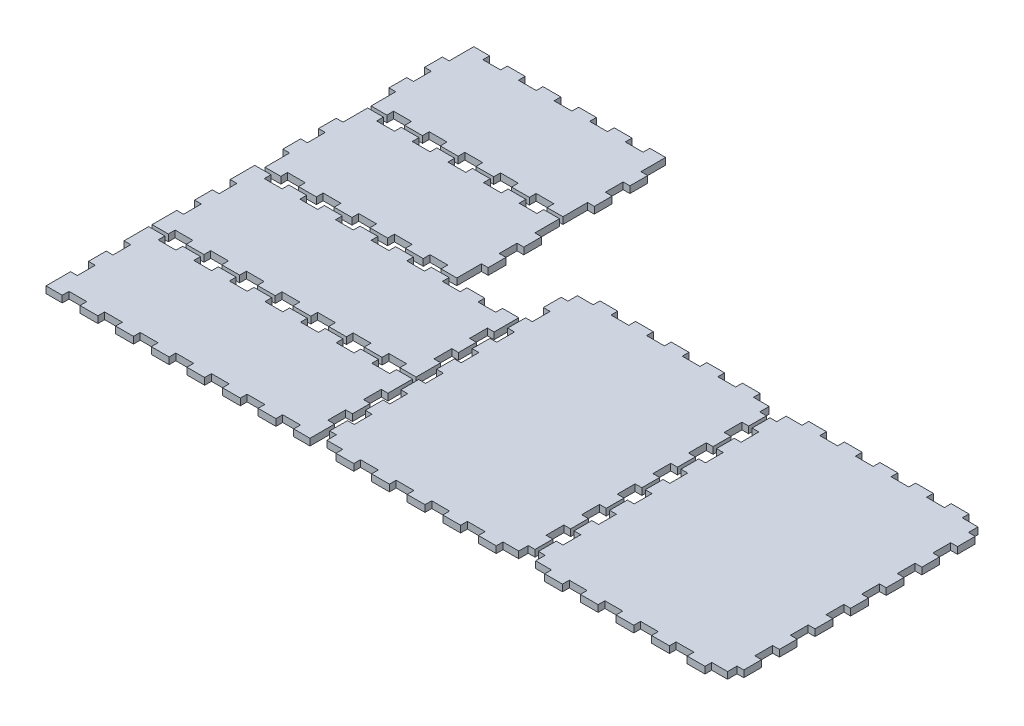
SolidWorks part; units mm, degrees
ref_plane "Front Plane" through (0, 0, 0) normal (0, 0, 1) x (1, 0, 0)
ref_plane "Top Plane" through (0, 0, 0) normal (0, 1, 0) x (1, 0, 0)
ref_plane "Right Plane" through (0, 0, 0) normal (1, 0, 0) x (0, 0, -1)
sketch "Sketch3" plane through (0, 0, 0) normal (0, 1, 0) x (1, 0, 0)
  line L0 (174.9552, 275.6916) -> (161.29, 275.6916)
  line L1 (161.29, 275.6916) -> (161.29, 269.8496)
  line L2 (161.29, 269.8496) -> (145.8722, 269.8496)
  line L3 (145.8722, 269.8496) -> (145.8722, 275.6916)
  line L4 (145.8722, 275.6916) -> (130.4544, 275.6916)
  line L5 (130.4544, 275.6916) -> (130.4544, 269.8496)
  line L6 (130.4544, 269.8496) -> (115.0366, 269.8496)
  line L7 (115.0366, 269.8496) -> (115.0366, 275.6916)
  line L8 (115.0366, 275.6916) -> (99.6188, 275.6916)
  line L9 (99.6188, 275.6916) -> (99.6188, 269.8496)
  line L10 (99.6188, 269.8496) -> (84.201, 269.8496)
  line L11 (84.201, 269.8496) -> (84.201, 275.6916)
  line L12 (84.201, 275.6916) -> (68.7578, 275.6916)
  line L13 (68.7578, 275.6916) -> (68.7578, 269.8496)
  line L14 (68.7578, 269.8496) -> (53.34, 269.8496)
  line L15 (53.34, 269.8496) -> (53.34, 275.6916)
  line L16 (53.34, 275.6916) -> (37.9222, 275.6916)
  line L17 (37.9222, 275.6916) -> (37.9222, 269.8496)
  line L18 (37.9222, 269.8496) -> (22.5044, 269.8496)
  line L19 (22.5044, 269.8496) -> (22.5044, 275.6916)
  line L20 (22.5044, 275.6916) -> (8.8392, 275.6916)
  line L21 (8.8392, 275.6916) -> (8.8392, 269.8496)
  line L22 (8.8392, 269.8496) -> (8.8392, 254.381)
  line L23 (8.8392, 254.381) -> (2.9972, 254.381)
  line L24 (2.9972, 254.381) -> (2.9972, 238.9632)
  line L25 (2.9972, 238.9632) -> (8.8392, 238.9632)
  line L26 (8.8392, 238.9632) -> (8.8392, 223.5454)
  line L27 (8.8392, 223.5454) -> (2.9972, 223.5454)
  line L28 (2.9972, 223.5454) -> (2.9972, 208.1276)
  line L29 (2.9972, 208.1276) -> (8.8392, 208.1276)
  line L30 (8.8392, 208.1276) -> (8.8392, 192.6336)
  line L31 (8.8392, 192.6336) -> (8.8392, 186.7916)
  line L32 (8.8392, 186.7916) -> (22.5044, 186.7916)
  line L33 (22.5044, 186.7916) -> (22.5044, 192.6336)
  line L34 (22.5044, 192.6336) -> (37.9222, 192.6336)
  line L35 (37.9222, 192.6336) -> (37.9222, 186.7916)
  line L36 (37.9222, 186.7916) -> (53.34, 186.7916)
  line L37 (53.34, 186.7916) -> (53.34, 192.6336)
  line L38 (53.34, 192.6336) -> (68.7578, 192.6336)
  line L39 (68.7578, 192.6336) -> (68.7578, 186.7916)
  line L40 (68.7578, 186.7916) -> (84.201, 186.7916)
  line L41 (84.201, 186.7916) -> (84.201, 192.6336)
  line L42 (84.201, 192.6336) -> (99.6188, 192.6336)
  line L43 (99.6188, 192.6336) -> (99.6188, 186.7916)
  line L44 (99.6188, 186.7916) -> (115.0366, 186.7916)
  line L45 (115.0366, 186.7916) -> (115.0366, 192.6336)
  line L46 (115.0366, 192.6336) -> (130.4544, 192.6336)
  line L47 (130.4544, 192.6336) -> (130.4544, 186.7916)
  line L48 (130.4544, 186.7916) -> (145.8722, 186.7916)
  line L49 (145.8722, 186.7916) -> (145.8722, 192.6336)
  line L50 (145.8722, 192.6336) -> (161.29, 192.6336)
  line L51 (161.29, 192.6336) -> (161.29, 186.7916)
  line L52 (161.29, 186.7916) -> (174.9552, 186.7916)
  line L53 (174.9552, 186.7916) -> (174.9552, 192.6336)
  line L54 (174.9552, 192.6336) -> (174.9552, 208.1276)
  line L55 (174.9552, 208.1276) -> (180.7972, 208.1276)
  line L56 (180.7972, 208.1276) -> (180.7972, 223.5454)
  line L57 (180.7972, 223.5454) -> (174.9552, 223.5454)
  line L58 (174.9552, 223.5454) -> (174.9552, 238.9632)
  line L59 (174.9552, 238.9632) -> (180.7972, 238.9632)
  line L60 (180.7972, 238.9632) -> (180.7972, 254.381)
  line L61 (180.7972, 254.381) -> (174.9552, 254.381)
  line L62 (174.9552, 254.381) -> (174.9552, 269.8496)
  line L63 (174.9552, 269.8496) -> (174.9552, 275.6916)
  line L64 (79.5782, 227.4824) -> (78.6384, 227.4824)
  line L65 (78.6384, 227.4824) -> (78.6384, 235.0262)
  line L66 (78.6384, 235.0262) -> (83.2358, 235.0262)
  line L67 (83.2358, 235.0262) -> (83.2358, 234.2134)
  line L68 (83.2358, 234.2134) -> (79.5782, 234.2134)
  line L69 (79.5782, 234.2134) -> (79.5782, 231.6988)
  line L70 (79.5782, 231.6988) -> (82.9818, 231.6988)
  line L71 (82.9818, 231.6988) -> (82.9818, 230.9114)
  line L72 (82.9818, 230.9114) -> (79.5782, 230.9114)
  line L73 (79.5782, 230.9114) -> (79.5782, 227.4824)
  line L74 (85.8774, 227.4824) -> (84.9376, 227.4824)
  line L75 (84.9376, 227.4824) -> (84.9376, 233.2228)
  line L76 (84.9376, 233.2228) -> (85.8774, 233.2228)
  line L77 (85.8774, 233.2228) -> (85.8774, 227.4824)
  line L78 (85.8774, 230.0732) -> (85.5726, 230.0732)
  line L79 (85.5726, 230.0732) -> (85.5726, 230.3018)
  line L80 (85.5726, 230.3018) -> (85.598, 230.505)
  line L81 (85.598, 230.505) -> (85.598, 230.7082)
  line L82 (85.598, 230.7082) -> (85.6234, 230.886)
  line L83 (85.6234, 230.886) -> (85.6234, 231.0638)
  line L84 (85.6234, 231.0638) -> (85.6488, 231.2416)
  line L85 (85.6488, 231.2416) -> (85.6742, 231.4194)
  line L86 (85.6742, 231.4194) -> (85.725, 231.5972)
  line L87 (85.725, 231.5972) -> (85.7504, 231.7496)
  line L88 (85.7504, 231.7496) -> (85.8012, 231.902)
  line L89 (85.8012, 231.902) -> (85.8266, 232.029)
  line L90 (85.8266, 232.029) -> (85.8774, 232.156)
  line L91 (85.8774, 232.156) -> (85.9282, 232.283)
  line L92 (85.9282, 232.283) -> (85.979, 232.41)
  line L93 (85.979, 232.41) -> (86.0552, 232.5116)
  line L94 (86.0552, 232.5116) -> (86.106, 232.6132)
  line L95 (86.106, 232.6132) -> (86.1822, 232.7148)
  line L96 (86.1822, 232.7148) -> (86.2584, 232.8164)
  line L97 (86.2584, 232.8164) -> (86.3346, 232.8926)
  line L98 (86.3346, 232.8926) -> (86.4108, 232.9688)
  line L99 (86.4108, 232.9688) -> (86.487, 233.045)
  line L100 (86.487, 233.045) -> (86.5632, 233.0958)
  line L101 (86.5632, 233.0958) -> (86.6648, 233.1466)
  line L102 (86.6648, 233.1466) -> (86.7664, 233.1974)
  line L103 (86.7664, 233.1974) -> (86.8426, 233.2482)
  line L104 (86.8426, 233.2482) -> (86.9442, 233.2736)
  line L105 (86.9442, 233.2736) -> (87.0458, 233.299)
  line L106 (87.0458, 233.299) -> (87.1728, 233.3244)
  line L107 (87.1728, 233.3244) -> (87.2744, 233.3244)
  line L108 (87.2744, 233.3244) -> (87.4014, 233.3244)
  line L109 (87.4014, 233.3244) -> (87.4268, 233.3244)
  line L110 (87.4268, 233.3244) -> (87.4776, 233.3244)
  line L111 (87.4776, 233.3244) -> (87.503, 233.3244)
  line L112 (87.503, 233.3244) -> (87.5284, 233.3244)
  line L113 (87.5284, 233.3244) -> (87.5792, 233.3244)
  line L114 (87.5792, 233.3244) -> (87.6046, 233.3244)
  line L115 (87.6046, 233.3244) -> (87.6554, 233.3244)
  line L116 (87.6554, 233.3244) -> (87.6808, 233.299)
  line L117 (87.6808, 233.299) -> (87.7062, 233.299)
  line L118 (87.7062, 233.299) -> (87.7316, 233.299)
  line L119 (87.7316, 233.299) -> (87.7824, 233.299)
  line L120 (87.7824, 233.299) -> (87.8078, 233.299)
  line L121 (87.8078, 233.299) -> (87.8332, 233.2736)
  line L122 (87.8332, 233.2736) -> (87.8586, 233.2736)
  line L123 (87.8586, 233.2736) -> (87.9094, 233.2736)
  line L124 (87.9094, 233.2736) -> (87.9348, 233.2482)
  line L125 (87.9348, 233.2482) -> (87.9602, 233.2482)
  line L126 (87.9602, 233.2482) -> (88.011, 233.2482)
  line L127 (88.011, 233.2482) -> (88.0364, 233.2228)
  line L128 (88.0364, 233.2228) -> (88.0618, 233.2228)
  line L129 (88.0618, 233.2228) -> (88.011, 232.283)
  line L130 (88.011, 232.283) -> (87.9602, 232.3084)
  line L131 (87.9602, 232.3084) -> (87.9348, 232.3084)
  line L132 (87.9348, 232.3084) -> (87.9094, 232.3338)
  line L133 (87.9094, 232.3338) -> (87.8586, 232.3338)
  line L134 (87.8586, 232.3338) -> (87.8332, 232.3338)
  line L135 (87.8332, 232.3338) -> (87.7824, 232.3592)
  line L136 (87.7824, 232.3592) -> (87.757, 232.3592)
  line L137 (87.757, 232.3592) -> (87.7062, 232.3592)
  line L138 (87.7062, 232.3592) -> (87.6808, 232.3846)
  line L139 (87.6808, 232.3846) -> (87.63, 232.3846)
  line L140 (87.63, 232.3846) -> (87.6046, 232.3846)
  line L141 (87.6046, 232.3846) -> (87.5538, 232.41)
  line L142 (87.5538, 232.41) -> (87.5284, 232.41)
  line L143 (87.5284, 232.41) -> (87.4776, 232.41)
  line L144 (87.4776, 232.41) -> (87.4522, 232.41)
  line L145 (87.4522, 232.41) -> (87.4268, 232.41)
  line L146 (87.4268, 232.41) -> (87.376, 232.4354)
  line L147 (87.376, 232.4354) -> (87.3506, 232.4354)
  line L148 (87.3506, 232.4354) -> (87.3252, 232.4354)
  line L149 (87.3252, 232.4354) -> (87.2744, 232.4354)
  line L150 (87.2744, 232.4354) -> (87.1728, 232.4354)
  line L151 (87.1728, 232.4354) -> (87.0966, 232.41)
  line L152 (87.0966, 232.41) -> (86.995, 232.41)
  line L153 (86.995, 232.41) -> (86.9188, 232.3846)
  line L154 (86.9188, 232.3846) -> (86.8172, 232.3592)
  line L155 (86.8172, 232.3592) -> (86.741, 232.3338)
  line L156 (86.741, 232.3338) -> (86.6648, 232.283)
  line L157 (86.6648, 232.283) -> (86.5886, 232.2322)
  line L158 (86.5886, 232.2322) -> (86.5378, 232.1814)
  line L159 (86.5378, 232.1814) -> (86.4616, 232.1306)
  line L160 (86.4616, 232.1306) -> (86.4108, 232.0798)
  line L161 (86.4108, 232.0798) -> (86.3346, 232.0036)
  line L162 (86.3346, 232.0036) -> (86.2838, 231.9274)
  line L163 (86.2838, 231.9274) -> (86.233, 231.8766)
  line L164 (86.233, 231.8766) -> (86.1822, 231.775)
  line L165 (86.1822, 231.775) -> (86.1568, 231.6988)
  line L166 (86.1568, 231.6988) -> (86.106, 231.6226)
  line L167 (86.106, 231.6226) -> (86.0806, 231.521)
  line L168 (86.0806, 231.521) -> (86.0298, 231.4194)
  line L169 (86.0298, 231.4194) -> (86.0044, 231.3178)
  line L170 (86.0044, 231.3178) -> (85.979, 231.2162)
  line L171 (85.979, 231.2162) -> (85.9536, 231.0892)
  line L172 (85.9536, 231.0892) -> (85.9282, 230.9876)
  line L173 (85.9282, 230.9876) -> (85.9282, 230.8606)
  line L174 (85.9282, 230.8606) -> (85.9028, 230.7336)
  line L175 (85.9028, 230.7336) -> (85.8774, 230.6066)
  line L176 (85.8774, 230.6066) -> (85.8774, 230.4796)
  line L177 (85.8774, 230.4796) -> (85.8774, 230.3526)
  line L178 (85.8774, 230.3526) -> (85.8774, 230.2256)
  line L179 (85.8774, 230.2256) -> (85.8774, 230.0732)
  line L180 (91.3384, 227.33) -> (91.186, 227.33)
  line L181 (91.186, 227.33) -> (91.0336, 227.3554)
  line L182 (91.0336, 227.3554) -> (90.9066, 227.3808)
  line L183 (90.9066, 227.3808) -> (90.7542, 227.4062)
  line L184 (90.7542, 227.4062) -> (90.6018, 227.4316)
  line L185 (90.6018, 227.4316) -> (90.4748, 227.457)
  line L186 (90.4748, 227.457) -> (90.3478, 227.5078)
  line L187 (90.3478, 227.5078) -> (90.2208, 227.5586)
  line L188 (90.2208, 227.5586) -> (90.0938, 227.6094)
  line L189 (90.0938, 227.6094) -> (89.9668, 227.6856)
  line L190 (89.9668, 227.6856) -> (89.8398, 227.7618)
  line L191 (89.8398, 227.7618) -> (89.7382, 227.838)
  line L192 (89.7382, 227.838) -> (89.6366, 227.9142)
  line L193 (89.6366, 227.9142) -> (89.535, 228.0158)
  line L194 (89.535, 228.0158) -> (89.4334, 228.1174)
  line L195 (89.4334, 228.1174) -> (89.3318, 228.219)
  line L196 (89.3318, 228.219) -> (89.2556, 228.3206)
  line L197 (89.2556, 228.3206) -> (89.1794, 228.4476)
  line L198 (89.1794, 228.4476) -> (89.0778, 228.5746)
  line L199 (89.0778, 228.5746) -> (89.027, 228.7016)
  line L200 (89.027, 228.7016) -> (88.9508, 228.8286)
  line L201 (88.9508, 228.8286) -> (88.9, 228.981)
  line L202 (88.9, 228.981) -> (88.8492, 229.1334)
  line L203 (88.8492, 229.1334) -> (88.7984, 229.2858)
  line L204 (88.7984, 229.2858) -> (88.7476, 229.4382)
  line L205 (88.7476, 229.4382) -> (88.7222, 229.616)
  line L206 (88.7222, 229.616) -> (88.6968, 229.7938)
  line L207 (88.6968, 229.7938) -> (88.6714, 229.9716)
  line L208 (88.6714, 229.9716) -> (88.6714, 230.1494)
  line L209 (88.6714, 230.1494) -> (88.6714, 230.3526)
  line L210 (88.6714, 230.3526) -> (88.6714, 230.5558)
  line L211 (88.6714, 230.5558) -> (88.6714, 230.7336)
  line L212 (88.6714, 230.7336) -> (88.6968, 230.9114)
  line L213 (88.6968, 230.9114) -> (88.7222, 231.0892)
  line L214 (88.7222, 231.0892) -> (88.7476, 231.267)
  line L215 (88.7476, 231.267) -> (88.7984, 231.4194)
  line L216 (88.7984, 231.4194) -> (88.8492, 231.5718)
  line L217 (88.8492, 231.5718) -> (88.9, 231.7242)
  line L218 (88.9, 231.7242) -> (88.9508, 231.8766)
  line L219 (88.9508, 231.8766) -> (89.027, 232.0036)
  line L220 (89.027, 232.0036) -> (89.0778, 232.1306)
  line L221 (89.0778, 232.1306) -> (89.1794, 232.2576)
  line L222 (89.1794, 232.2576) -> (89.2556, 232.3846)
  line L223 (89.2556, 232.3846) -> (89.3318, 232.4862)
  line L224 (89.3318, 232.4862) -> (89.4334, 232.5878)
  line L225 (89.4334, 232.5878) -> (89.535, 232.6894)
  line L226 (89.535, 232.6894) -> (89.6366, 232.791)
  line L227 (89.6366, 232.791) -> (89.7382, 232.8672)
  line L228 (89.7382, 232.8672) -> (89.8398, 232.9434)
  line L229 (89.8398, 232.9434) -> (89.9668, 233.0196)
  line L230 (89.9668, 233.0196) -> (90.0938, 233.0958)
  line L231 (90.0938, 233.0958) -> (90.2208, 233.1466)
  line L232 (90.2208, 233.1466) -> (90.3478, 233.1974)
  line L233 (90.3478, 233.1974) -> (90.4748, 233.2482)
  line L234 (90.4748, 233.2482) -> (90.6018, 233.2736)
  line L235 (90.6018, 233.2736) -> (90.7542, 233.299)
  line L236 (90.7542, 233.299) -> (90.9066, 233.3244)
  line L237 (90.9066, 233.3244) -> (91.0336, 233.3498)
  line L238 (91.0336, 233.3498) -> (91.186, 233.3498)
  line L239 (91.186, 233.3498) -> (91.3384, 233.3752)
  line L240 (91.3384, 233.3752) -> (91.4908, 233.3498)
  line L241 (91.4908, 233.3498) -> (91.6432, 233.3498)
  line L242 (91.6432, 233.3498) -> (91.7956, 233.3244)
  line L243 (91.7956, 233.3244) -> (91.9226, 233.299)
  line L244 (91.9226, 233.299) -> (92.075, 233.2736)
  line L245 (92.075, 233.2736) -> (92.202, 233.2482)
  line L246 (92.202, 233.2482) -> (92.329, 233.1974)
  line L247 (92.329, 233.1974) -> (92.456, 233.1466)
  line L248 (92.456, 233.1466) -> (92.583, 233.0958)
  line L249 (92.583, 233.0958) -> (92.71, 233.0196)
  line L250 (92.71, 233.0196) -> (92.837, 232.9434)
  line L251 (92.837, 232.9434) -> (92.9386, 232.8672)
  line L252 (92.9386, 232.8672) -> (93.0656, 232.791)
  line L253 (93.0656, 232.791) -> (93.1672, 232.6894)
  line L254 (93.1672, 232.6894) -> (93.2434, 232.5878)
  line L255 (93.2434, 232.5878) -> (93.345, 232.4862)
  line L256 (93.345, 232.4862) -> (93.4466, 232.3846)
  line L257 (93.4466, 232.3846) -> (93.5228, 232.2576)
  line L258 (93.5228, 232.2576) -> (93.599, 232.1306)
  line L259 (93.599, 232.1306) -> (93.6752, 232.0036)
  line L260 (93.6752, 232.0036) -> (93.726, 231.8766)
  line L261 (93.726, 231.8766) -> (93.7768, 231.7242)
  line L262 (93.7768, 231.7242) -> (93.853, 231.5718)
  line L263 (93.853, 231.5718) -> (93.8784, 231.4194)
  line L264 (93.8784, 231.4194) -> (93.9292, 231.267)
  line L265 (93.9292, 231.267) -> (93.9546, 231.0892)
  line L266 (93.9546, 231.0892) -> (93.98, 230.9114)
  line L267 (93.98, 230.9114) -> (94.0054, 230.7336)
  line L268 (94.0054, 230.7336) -> (94.0054, 230.5558)
  line L269 (94.0054, 230.5558) -> (94.0054, 230.3526)
  line L270 (94.0054, 230.3526) -> (94.0054, 230.1494)
  line L271 (94.0054, 230.1494) -> (94.0054, 229.9716)
  line L272 (94.0054, 229.9716) -> (93.98, 229.7938)
  line L273 (93.98, 229.7938) -> (93.9546, 229.616)
  line L274 (93.9546, 229.616) -> (93.9292, 229.4382)
  line L275 (93.9292, 229.4382) -> (93.8784, 229.2858)
  line L276 (93.8784, 229.2858) -> (93.853, 229.1334)
  line L277 (93.853, 229.1334) -> (93.7768, 228.981)
  line L278 (93.7768, 228.981) -> (93.726, 228.8286)
  line L279 (93.726, 228.8286) -> (93.6752, 228.7016)
  line L280 (93.6752, 228.7016) -> (93.599, 228.5746)
  line L281 (93.599, 228.5746) -> (93.5228, 228.4476)
  line L282 (93.5228, 228.4476) -> (93.4466, 228.3206)
  line L283 (93.4466, 228.3206) -> (93.345, 228.219)
  line L284 (93.345, 228.219) -> (93.2434, 228.1174)
  line L285 (93.2434, 228.1174) -> (93.1672, 228.0158)
  line L286 (93.1672, 228.0158) -> (93.0656, 227.9142)
  line L287 (93.0656, 227.9142) -> (92.9386, 227.838)
  line L288 (92.9386, 227.838) -> (92.837, 227.7618)
  line L289 (92.837, 227.7618) -> (92.71, 227.6856)
  line L290 (92.71, 227.6856) -> (92.583, 227.6094)
  line L291 (92.583, 227.6094) -> (92.456, 227.5586)
  line L292 (92.456, 227.5586) -> (92.329, 227.5078)
  line L293 (92.329, 227.5078) -> (92.202, 227.457)
  line L294 (92.202, 227.457) -> (92.075, 227.4316)
  line L295 (92.075, 227.4316) -> (91.9226, 227.4062)
  line L296 (91.9226, 227.4062) -> (91.7956, 227.3808)
  line L297 (91.7956, 227.3808) -> (91.6432, 227.3554)
  line L298 (91.6432, 227.3554) -> (91.4908, 227.33)
  line L299 (91.4908, 227.33) -> (91.3384, 227.33)
  line L300 (91.313, 228.1428) -> (91.44, 228.1682)
  line L301 (91.44, 228.1682) -> (91.5416, 228.1682)
  line L302 (91.5416, 228.1682) -> (91.6432, 228.1682)
  line L303 (91.6432, 228.1682) -> (91.7448, 228.1936)
  line L304 (91.7448, 228.1936) -> (91.8464, 228.219)
  line L305 (91.8464, 228.219) -> (91.9226, 228.2444)
  line L306 (91.9226, 228.2444) -> (92.0242, 228.2952)
  line L307 (92.0242, 228.2952) -> (92.1004, 228.3206)
  line L308 (92.1004, 228.3206) -> (92.202, 228.3714)
  line L309 (92.202, 228.3714) -> (92.2782, 228.4222)
  line L310 (92.2782, 228.4222) -> (92.3544, 228.473)
  line L311 (92.3544, 228.473) -> (92.4052, 228.5492)
  line L312 (92.4052, 228.5492) -> (92.4814, 228.6)
  line L313 (92.4814, 228.6) -> (92.5576, 228.6762)
  line L314 (92.5576, 228.6762) -> (92.6084, 228.7524)
  line L315 (92.6084, 228.7524) -> (92.6592, 228.8286)
  line L316 (92.6592, 228.8286) -> (92.7354, 228.9048)
  line L317 (92.7354, 228.9048) -> (92.7608, 228.981)
  line L318 (92.7608, 228.981) -> (92.8116, 229.0826)
  line L319 (92.8116, 229.0826) -> (92.8624, 229.1842)
  line L320 (92.8624, 229.1842) -> (92.8878, 229.2858)
  line L321 (92.8878, 229.2858) -> (92.9386, 229.3874)
  line L322 (92.9386, 229.3874) -> (92.964, 229.489)
  line L323 (92.964, 229.489) -> (92.9894, 229.616)
  line L324 (92.9894, 229.616) -> (93.0148, 229.7176)
  line L325 (93.0148, 229.7176) -> (93.0402, 229.8446)
  line L326 (93.0402, 229.8446) -> (93.0402, 229.9716)
  line L327 (93.0402, 229.9716) -> (93.0656, 230.0986)
  line L328 (93.0656, 230.0986) -> (93.0656, 230.2256)
  line L329 (93.0656, 230.2256) -> (93.0656, 230.3526)
  line L330 (93.0656, 230.3526) -> (93.0656, 230.5558)
  line L331 (93.0656, 230.5558) -> (93.0402, 230.7336)
  line L332 (93.0402, 230.7336) -> (93.0148, 230.9368)
  line L333 (93.0148, 230.9368) -> (92.9894, 231.1146)
  line L334 (92.9894, 231.1146) -> (92.964, 231.267)
  line L335 (92.964, 231.267) -> (92.9132, 231.4194)
  line L336 (92.9132, 231.4194) -> (92.8624, 231.5718)
  line L337 (92.8624, 231.5718) -> (92.7862, 231.7242)
  line L338 (92.7862, 231.7242) -> (92.71, 231.8512)
  line L339 (92.71, 231.8512) -> (92.6338, 231.9782)
  line L340 (92.6338, 231.9782) -> (92.5576, 232.0798)
  line L341 (92.5576, 232.0798) -> (92.456, 232.1814)
  line L342 (92.456, 232.1814) -> (92.3544, 232.2576)
  line L343 (92.3544, 232.2576) -> (92.2274, 232.3338)
  line L344 (92.2274, 232.3338) -> (92.1004, 232.41)
  line L345 (92.1004, 232.41) -> (91.9734, 232.4608)
  line L346 (91.9734, 232.4608) -> (91.8464, 232.5116)
  line L347 (91.8464, 232.5116) -> (91.694, 232.537)
  line L348 (91.694, 232.537) -> (91.5416, 232.5624)
  line L349 (91.5416, 232.5624) -> (91.3638, 232.5624)
  line L350 (91.3638, 232.5624) -> (91.2622, 232.5624)
  line L351 (91.2622, 232.5624) -> (91.1606, 232.537)
  line L352 (91.1606, 232.537) -> (91.059, 232.537)
  line L353 (91.059, 232.537) -> (90.9574, 232.5116)
  line L354 (90.9574, 232.5116) -> (90.8558, 232.4862)
  line L355 (90.8558, 232.4862) -> (90.7542, 232.4608)
  line L356 (90.7542, 232.4608) -> (90.678, 232.4354)
  line L357 (90.678, 232.4354) -> (90.5764, 232.3846)
  line L358 (90.5764, 232.3846) -> (90.5002, 232.3338)
  line L359 (90.5002, 232.3338) -> (90.424, 232.283)
  line L360 (90.424, 232.283) -> (90.3478, 232.2322)
  line L361 (90.3478, 232.2322) -> (90.2716, 232.1814)
  line L362 (90.2716, 232.1814) -> (90.1954, 232.1052)
  line L363 (90.1954, 232.1052) -> (90.1446, 232.0544)
  line L364 (90.1446, 232.0544) -> (90.0684, 231.9782)
  line L365 (90.0684, 231.9782) -> (90.0176, 231.902)
  line L366 (90.0176, 231.902) -> (89.9668, 231.8004)
  line L367 (89.9668, 231.8004) -> (89.916, 231.7242)
  line L368 (89.916, 231.7242) -> (89.8652, 231.6226)
  line L369 (89.8652, 231.6226) -> (89.8398, 231.521)
  line L370 (89.8398, 231.521) -> (89.789, 231.4194)
  line L371 (89.789, 231.4194) -> (89.7636, 231.3178)
  line L372 (89.7636, 231.3178) -> (89.7382, 231.2162)
  line L373 (89.7382, 231.2162) -> (89.7128, 231.1146)
  line L374 (89.7128, 231.1146) -> (89.6874, 230.9876)
  line L375 (89.6874, 230.9876) -> (89.662, 230.8606)
  line L376 (89.662, 230.8606) -> (89.6366, 230.7336)
  line L377 (89.6366, 230.7336) -> (89.6366, 230.6066)
  line L378 (89.6366, 230.6066) -> (89.6366, 230.4796)
  line L379 (89.6366, 230.4796) -> (89.6366, 230.3526)
  line L380 (89.6366, 230.3526) -> (89.6366, 230.1494)
  line L381 (89.6366, 230.1494) -> (89.6366, 229.9716)
  line L382 (89.6366, 229.9716) -> (89.662, 229.7684)
  line L383 (89.662, 229.7684) -> (89.6874, 229.616)
  line L384 (89.6874, 229.616) -> (89.7382, 229.4382)
  line L385 (89.7382, 229.4382) -> (89.789, 229.2858)
  line L386 (89.789, 229.2858) -> (89.8398, 229.1334)
  line L387 (89.8398, 229.1334) -> (89.916, 229.0064)
  line L388 (89.916, 229.0064) -> (89.9668, 228.8794)
  line L389 (89.9668, 228.8794) -> (90.0684, 228.7524)
  line L390 (90.0684, 228.7524) -> (90.1446, 228.6254)
  line L391 (90.1446, 228.6254) -> (90.2462, 228.5238)
  line L392 (90.2462, 228.5238) -> (90.3478, 228.4476)
  line L393 (90.3478, 228.4476) -> (90.4748, 228.3714)
  line L394 (90.4748, 228.3714) -> (90.5764, 228.2952)
  line L395 (90.5764, 228.2952) -> (90.7288, 228.2444)
  line L396 (90.7288, 228.2444) -> (90.8558, 228.219)
  line L397 (90.8558, 228.219) -> (91.0082, 228.1682)
  line L398 (91.0082, 228.1682) -> (91.1606, 228.1682)
  line L399 (91.1606, 228.1682) -> (91.313, 228.1428)
  line L400 (100.838, 227.4824) -> (99.8982, 227.4824)
  line L401 (99.8982, 227.4824) -> (99.8982, 230.8606)
  line L402 (99.8982, 230.8606) -> (99.8982, 231.013)
  line L403 (99.8982, 231.013) -> (99.8982, 231.1654)
  line L404 (99.8982, 231.1654) -> (99.8728, 231.3178)
  line L405 (99.8728, 231.3178) -> (99.8474, 231.4448)
  line L406 (99.8474, 231.4448) -> (99.7966, 231.5718)
  line L407 (99.7966, 231.5718) -> (99.7712, 231.6988)
  line L408 (99.7712, 231.6988) -> (99.7204, 231.8258)
  line L409 (99.7204, 231.8258) -> (99.6442, 231.9274)
  line L410 (99.6442, 231.9274) -> (99.5934, 232.0036)
  line L411 (99.5934, 232.0036) -> (99.5172, 232.1052)
  line L412 (99.5172, 232.1052) -> (99.441, 232.1814)
  line L413 (99.441, 232.1814) -> (99.3394, 232.2576)
  line L414 (99.3394, 232.2576) -> (99.2632, 232.3338)
  line L415 (99.2632, 232.3338) -> (99.1616, 232.3846)
  line L416 (99.1616, 232.3846) -> (99.06, 232.4354)
  line L417 (99.06, 232.4354) -> (98.933, 232.4608)
  line L418 (98.933, 232.4608) -> (98.8314, 232.4862)
  line L419 (98.8314, 232.4862) -> (98.7044, 232.5116)
  line L420 (98.7044, 232.5116) -> (98.5774, 232.537)
  line L421 (98.5774, 232.537) -> (98.4504, 232.537)
  line L422 (98.4504, 232.537) -> (98.3488, 232.537)
  line L423 (98.3488, 232.537) -> (98.2472, 232.5116)
  line L424 (98.2472, 232.5116) -> (98.1456, 232.5116)
  line L425 (98.1456, 232.5116) -> (98.044, 232.4862)
  line L426 (98.044, 232.4862) -> (97.9678, 232.4608)
  line L427 (97.9678, 232.4608) -> (97.8662, 232.4354)
  line L428 (97.8662, 232.4354) -> (97.79, 232.3846)
  line L429 (97.79, 232.3846) -> (97.7138, 232.3592)
  line L430 (97.7138, 232.3592) -> (97.6376, 232.3084)
  line L431 (97.6376, 232.3084) -> (97.5614, 232.2576)
  line L432 (97.5614, 232.2576) -> (97.4852, 232.2068)
  line L433 (97.4852, 232.2068) -> (97.409, 232.1306)
  line L434 (97.409, 232.1306) -> (97.3328, 232.0544)
  line L435 (97.3328, 232.0544) -> (97.282, 231.9782)
  line L436 (97.282, 231.9782) -> (97.2058, 231.902)
  line L437 (97.2058, 231.902) -> (97.155, 231.8258)
  line L438 (97.155, 231.8258) -> (97.1042, 231.7496)
  line L439 (97.1042, 231.7496) -> (97.0534, 231.648)
  line L440 (97.0534, 231.648) -> (97.0026, 231.5464)
  line L441 (97.0026, 231.5464) -> (96.9772, 231.4448)
  line L442 (96.9772, 231.4448) -> (96.9264, 231.3432)
  line L443 (96.9264, 231.3432) -> (96.901, 231.2162)
  line L444 (96.901, 231.2162) -> (96.8756, 231.1146)
  line L445 (96.8756, 231.1146) -> (96.8248, 230.9876)
  line L446 (96.8248, 230.9876) -> (96.8248, 230.8606)
  line L447 (96.8248, 230.8606) -> (96.7994, 230.7336)
  line L448 (96.7994, 230.7336) -> (96.774, 230.6066)
  line L449 (96.774, 230.6066) -> (96.774, 230.4796)
  line L450 (96.774, 230.4796) -> (96.774, 230.3272)
  line L451 (96.774, 230.3272) -> (96.774, 230.2002)
  line L452 (96.774, 230.2002) -> (96.393, 230.2002)
  line L453 (96.393, 230.2002) -> (96.4184, 230.4034)
  line L454 (96.4184, 230.4034) -> (96.4184, 230.5812)
  line L455 (96.4184, 230.5812) -> (96.4184, 230.759)
  line L456 (96.4184, 230.759) -> (96.4438, 230.9622)
  line L457 (96.4438, 230.9622) -> (96.4692, 231.1146)
  line L458 (96.4692, 231.1146) -> (96.4946, 231.2924)
  line L459 (96.4946, 231.2924) -> (96.5454, 231.4448)
  line L460 (96.5454, 231.4448) -> (96.5708, 231.6226)
  line L461 (96.5708, 231.6226) -> (96.6216, 231.7496)
  line L462 (96.6216, 231.7496) -> (96.6724, 231.902)
  line L463 (96.6724, 231.902) -> (96.7232, 232.0544)
  line L464 (96.7232, 232.0544) -> (96.774, 232.1814)
  line L465 (96.774, 232.1814) -> (96.8502, 232.3084)
  line L466 (96.8502, 232.3084) -> (96.9264, 232.41)
  line L467 (96.9264, 232.41) -> (97.0026, 232.537)
  line L468 (97.0026, 232.537) -> (97.0788, 232.6386)
  line L469 (97.0788, 232.6386) -> (97.155, 232.7402)
  line L470 (97.155, 232.7402) -> (97.2566, 232.8164)
  line L471 (97.2566, 232.8164) -> (97.3328, 232.918)
  line L472 (97.3328, 232.918) -> (97.4344, 232.9942)
  line L473 (97.4344, 232.9942) -> (97.536, 233.0704)
  line L474 (97.536, 233.0704) -> (97.6376, 233.1212)
  line L475 (97.6376, 233.1212) -> (97.7646, 233.172)
  line L476 (97.7646, 233.172) -> (97.8916, 233.2228)
  line L477 (97.8916, 233.2228) -> (97.9932, 233.2736)
  line L478 (97.9932, 233.2736) -> (98.1202, 233.299)
  line L479 (98.1202, 233.299) -> (98.2472, 233.3244)
  line L480 (98.2472, 233.3244) -> (98.3996, 233.3498)
  line L481 (98.3996, 233.3498) -> (98.5266, 233.3498)
  line L482 (98.5266, 233.3498) -> (98.679, 233.3752)
  line L483 (98.679, 233.3752) -> (98.806, 233.3498)
  line L484 (98.806, 233.3498) -> (98.933, 233.3498)
  line L485 (98.933, 233.3498) -> (99.06, 233.3244)
  line L486 (99.06, 233.3244) -> (99.187, 233.3244)
  line L487 (99.187, 233.3244) -> (99.2886, 233.299)
  line L488 (99.2886, 233.299) -> (99.4156, 233.2482)
  line L489 (99.4156, 233.2482) -> (99.5172, 233.2228)
  line L490 (99.5172, 233.2228) -> (99.6188, 233.172)
  line L491 (99.6188, 233.172) -> (99.7458, 233.1212)
  line L492 (99.7458, 233.1212) -> (99.822, 233.0704)
  line L493 (99.822, 233.0704) -> (99.9236, 232.9942)
  line L494 (99.9236, 232.9942) -> (100.0252, 232.918)
  line L495 (100.0252, 232.918) -> (100.1014, 232.8672)
  line L496 (100.1014, 232.8672) -> (100.1776, 232.7656)
  line L497 (100.1776, 232.7656) -> (100.2538, 232.6894)
  line L498 (100.2538, 232.6894) -> (100.33, 232.6132)
  line L499 (100.33, 232.6132) -> (100.4062, 232.5116)
  line L500 (100.4062, 232.5116) -> (100.457, 232.41)
  line L501 (100.457, 232.41) -> (100.5078, 232.3084)
  line L502 (100.5078, 232.3084) -> (100.584, 232.1814)
  line L503 (100.584, 232.1814) -> (100.6348, 232.0798)
  line L504 (100.6348, 232.0798) -> (100.6602, 231.9528)
  line L505 (100.6602, 231.9528) -> (100.711, 231.8258)
  line L506 (100.711, 231.8258) -> (100.7364, 231.6988)
  line L507 (100.7364, 231.6988) -> (100.7618, 231.5718)
  line L508 (100.7618, 231.5718) -> (100.7872, 231.4448)
  line L509 (100.7872, 231.4448) -> (100.8126, 231.2924)
  line L510 (100.8126, 231.2924) -> (100.8126, 231.1654)
  line L511 (100.8126, 231.1654) -> (100.838, 231.013)
  line L512 (100.838, 231.013) -> (100.838, 230.8606)
  line L513 (100.838, 230.8606) -> (100.838, 227.4824)
  line L514 (96.774, 227.4824) -> (95.8342, 227.4824)
  line L515 (95.8342, 227.4824) -> (95.8342, 233.2228)
  line L516 (95.8342, 233.2228) -> (96.6216, 233.2228)
  line L517 (96.6216, 233.2228) -> (96.774, 231.902)
  line L518 (96.774, 231.902) -> (96.774, 227.4824)
  line L519 (104.8258, 227.33) -> (104.7496, 227.33)
  line L520 (104.7496, 227.33) -> (104.648, 227.3554)
  line L521 (104.648, 227.3554) -> (104.5718, 227.3554)
  line L522 (104.5718, 227.3554) -> (104.4702, 227.3554)
  line L523 (104.4702, 227.3554) -> (104.394, 227.3808)
  line L524 (104.394, 227.3808) -> (104.3178, 227.4062)
  line L525 (104.3178, 227.4062) -> (104.2162, 227.4316)
  line L526 (104.2162, 227.4316) -> (104.14, 227.457)
  line L527 (104.14, 227.457) -> (104.0638, 227.4824)
  line L528 (104.0638, 227.4824) -> (103.9876, 227.5078)
  line L529 (103.9876, 227.5078) -> (103.9114, 227.5586)
  line L530 (103.9114, 227.5586) -> (103.8606, 227.6094)
  line L531 (103.8606, 227.6094) -> (103.7844, 227.6348)
  line L532 (103.7844, 227.6348) -> (103.7082, 227.6856)
  line L533 (103.7082, 227.6856) -> (103.6574, 227.7364)
  line L534 (103.6574, 227.7364) -> (103.6066, 227.7872)
  line L535 (103.6066, 227.7872) -> (103.5558, 227.8634)
  line L536 (103.5558, 227.8634) -> (103.505, 227.9142)
  line L537 (103.505, 227.9142) -> (103.4542, 227.9904)
  line L538 (103.4542, 227.9904) -> (103.4034, 228.0666)
  line L539 (103.4034, 228.0666) -> (103.3526, 228.1428)
  line L540 (103.3526, 228.1428) -> (103.3272, 228.219)
  line L541 (103.3272, 228.219) -> (103.3018, 228.2952)
  line L542 (103.3018, 228.2952) -> (103.2764, 228.3714)
  line L543 (103.2764, 228.3714) -> (103.251, 228.473)
  line L544 (103.251, 228.473) -> (103.2256, 228.5492)
  line L545 (103.2256, 228.5492) -> (103.2002, 228.6508)
  line L546 (103.2002, 228.6508) -> (103.2002, 228.7524)
  line L547 (103.2002, 228.7524) -> (103.2002, 228.854)
  line L548 (103.2002, 228.854) -> (103.2002, 228.9556)
  line L549 (103.2002, 228.9556) -> (103.2002, 234.823)
  line L550 (103.2002, 234.823) -> (104.1146, 234.823)
  line L551 (104.1146, 234.823) -> (104.1146, 228.981)
  line L552 (104.1146, 228.981) -> (104.1146, 228.8032)
  line L553 (104.1146, 228.8032) -> (104.14, 228.6508)
  line L554 (104.14, 228.6508) -> (104.1908, 228.5238)
  line L555 (104.1908, 228.5238) -> (104.2416, 228.4222)
  line L556 (104.2416, 228.4222) -> (104.3178, 228.3206)
  line L557 (104.3178, 228.3206) -> (104.4194, 228.2444)
  line L558 (104.4194, 228.2444) -> (104.521, 228.1682)
  line L559 (104.521, 228.1682) -> (104.648, 228.1428)
  line L560 (104.648, 228.1428) -> (104.775, 228.092)
  line L561 (104.775, 228.092) -> (104.9528, 228.092)
  line L562 (104.9528, 228.092) -> (104.9782, 228.092)
  line L563 (104.9782, 228.092) -> (105.029, 228.092)
  line L564 (105.029, 228.092) -> (105.0798, 228.092)
  line L565 (105.0798, 228.092) -> (105.1306, 228.092)
  line L566 (105.1306, 228.092) -> (105.1814, 228.1174)
  line L567 (105.1814, 228.1174) -> (105.2322, 228.1174)
  line L568 (105.2322, 228.1174) -> (105.283, 228.1174)
  line L569 (105.283, 228.1174) -> (105.3338, 228.1174)
  line L570 (105.3338, 228.1174) -> (105.3846, 228.1428)
  line L571 (105.3846, 228.1428) -> (105.41, 228.1428)
  line L572 (105.41, 228.1428) -> (105.4608, 228.1682)
  line L573 (105.4608, 228.1682) -> (105.5116, 228.1682)
  line L574 (105.5116, 228.1682) -> (105.5624, 228.1936)
  line L575 (105.5624, 228.1936) -> (105.6132, 228.1936)
  line L576 (105.6132, 228.1936) -> (105.664, 228.219)
  line L577 (105.664, 228.219) -> (105.7148, 228.2444)
  line L578 (105.7148, 228.2444) -> (105.7656, 228.2444)
  line L579 (105.7656, 228.2444) -> (105.8164, 228.2698)
  line L580 (105.8164, 228.2698) -> (105.8926, 228.2952)
  line L581 (105.8926, 228.2952) -> (105.9434, 228.3206)
  line L582 (105.9434, 228.3206) -> (106.0704, 227.6348)
  line L583 (106.0704, 227.6348) -> (106.0196, 227.6094)
  line L584 (106.0196, 227.6094) -> (105.9434, 227.584)
  line L585 (105.9434, 227.584) -> (105.8926, 227.5586)
  line L586 (105.8926, 227.5586) -> (105.8164, 227.5332)
  line L587 (105.8164, 227.5332) -> (105.7656, 227.5078)
  line L588 (105.7656, 227.5078) -> (105.7148, 227.5078)
  line L589 (105.7148, 227.5078) -> (105.6386, 227.4824)
  line L590 (105.6386, 227.4824) -> (105.5878, 227.457)
  line L591 (105.5878, 227.457) -> (105.5116, 227.4316)
  line L592 (105.5116, 227.4316) -> (105.4608, 227.4316)
  line L593 (105.4608, 227.4316) -> (105.41, 227.4062)
  line L594 (105.41, 227.4062) -> (105.3338, 227.3808)
  line L595 (105.3338, 227.3808) -> (105.283, 227.3808)
  line L596 (105.283, 227.3808) -> (105.2068, 227.3808)
  line L597 (105.2068, 227.3808) -> (105.156, 227.3554)
  line L598 (105.156, 227.3554) -> (105.0798, 227.3554)
  line L599 (105.0798, 227.3554) -> (105.029, 227.3554)
  line L600 (105.029, 227.3554) -> (104.9528, 227.33)
  line L601 (104.9528, 227.33) -> (104.902, 227.33)
  line L602 (104.902, 227.33) -> (104.8258, 227.33)
  line L603 (105.918, 232.5624) -> (102.2604, 232.5624)
  line L604 (102.2604, 232.5624) -> (102.2604, 233.2228)
  line L605 (102.2604, 233.2228) -> (105.918, 233.2228)
  line L606 (105.918, 233.2228) -> (105.918, 232.5624)
  line L607 (174.9552, 367.6142) -> (161.29, 367.6142)
  line L608 (161.29, 367.6142) -> (161.29, 361.7722)
  line L609 (161.29, 361.7722) -> (145.8722, 361.7722)
  line L610 (145.8722, 361.7722) -> (145.8722, 367.6142)
  line L611 (145.8722, 367.6142) -> (130.4544, 367.6142)
  line L612 (130.4544, 367.6142) -> (130.4544, 361.7722)
  line L613 (130.4544, 361.7722) -> (115.0366, 361.7722)
  line L614 (115.0366, 361.7722) -> (115.0366, 367.6142)
  line L615 (115.0366, 367.6142) -> (99.6188, 367.6142)
  line L616 (99.6188, 367.6142) -> (99.6188, 361.7722)
  line L617 (99.6188, 361.7722) -> (84.201, 361.7722)
  line L618 (84.201, 361.7722) -> (84.201, 367.6142)
  line L619 (84.201, 367.6142) -> (68.7578, 367.6142)
  line L620 (68.7578, 367.6142) -> (68.7578, 361.7722)
  line L621 (68.7578, 361.7722) -> (53.34, 361.7722)
  line L622 (53.34, 361.7722) -> (53.34, 367.6142)
  line L623 (53.34, 367.6142) -> (37.9222, 367.6142)
  line L624 (37.9222, 367.6142) -> (37.9222, 361.7722)
  line L625 (37.9222, 361.7722) -> (22.5044, 361.7722)
  line L626 (22.5044, 361.7722) -> (22.5044, 367.6142)
  line L627 (22.5044, 367.6142) -> (8.8392, 367.6142)
  line L628 (8.8392, 367.6142) -> (8.8392, 361.7722)
  line L629 (8.8392, 361.7722) -> (8.8392, 346.2782)
  line L630 (8.8392, 346.2782) -> (2.9972, 346.2782)
  line L631 (2.9972, 346.2782) -> (2.9972, 330.8604)
  line L632 (2.9972, 330.8604) -> (8.8392, 330.8604)
  line L633 (8.8392, 330.8604) -> (8.8392, 315.4426)
  line L634 (8.8392, 315.4426) -> (2.9972, 315.4426)
  line L635 (2.9972, 315.4426) -> (2.9972, 300.0248)
  line L636 (2.9972, 300.0248) -> (8.8392, 300.0248)
  line L637 (8.8392, 300.0248) -> (8.8392, 284.5308)
  line L638 (8.8392, 284.5308) -> (8.8392, 278.6888)
  line L639 (8.8392, 278.6888) -> (22.5044, 278.6888)
  line L640 (22.5044, 278.6888) -> (22.5044, 284.5308)
  line L641 (22.5044, 284.5308) -> (37.9222, 284.5308)
  line L642 (37.9222, 284.5308) -> (37.9222, 278.6888)
  line L643 (37.9222, 278.6888) -> (53.34, 278.6888)
  line L644 (53.34, 278.6888) -> (53.34, 284.5308)
  line L645 (53.34, 284.5308) -> (68.7578, 284.5308)
  line L646 (68.7578, 284.5308) -> (68.7578, 278.6888)
  line L647 (68.7578, 278.6888) -> (84.201, 278.6888)
  line L648 (84.201, 278.6888) -> (84.201, 284.5308)
  line L649 (84.201, 284.5308) -> (99.6188, 284.5308)
  line L650 (99.6188, 284.5308) -> (99.6188, 278.6888)
  line L651 (99.6188, 278.6888) -> (115.0366, 278.6888)
  line L652 (115.0366, 278.6888) -> (115.0366, 284.5308)
  line L653 (115.0366, 284.5308) -> (130.4544, 284.5308)
  line L654 (130.4544, 284.5308) -> (130.4544, 278.6888)
  line L655 (130.4544, 278.6888) -> (145.8722, 278.6888)
  line L656 (145.8722, 278.6888) -> (145.8722, 284.5308)
  line L657 (145.8722, 284.5308) -> (161.29, 284.5308)
  line L658 (161.29, 284.5308) -> (161.29, 278.6888)
  line L659 (161.29, 278.6888) -> (174.9552, 278.6888)
  line L660 (174.9552, 278.6888) -> (174.9552, 284.5308)
  line L661 (174.9552, 284.5308) -> (174.9552, 300.0248)
  line L662 (174.9552, 300.0248) -> (180.7972, 300.0248)
  line L663 (180.7972, 300.0248) -> (180.7972, 315.4426)
  line L664 (180.7972, 315.4426) -> (174.9552, 315.4426)
  line L665 (174.9552, 315.4426) -> (174.9552, 330.8604)
  line L666 (174.9552, 330.8604) -> (180.7972, 330.8604)
  line L667 (180.7972, 330.8604) -> (180.7972, 346.2782)
  line L668 (180.7972, 346.2782) -> (174.9552, 346.2782)
  line L669 (174.9552, 346.2782) -> (174.9552, 361.7722)
  line L670 (174.9552, 361.7722) -> (174.9552, 367.6142)
  line L671 (82.423, 319.0494) -> (79.6036, 319.0494)
  line L672 (79.6036, 319.0494) -> (79.6036, 326.5932)
  line L673 (79.6036, 326.5932) -> (82.423, 326.5932)
  line L674 (82.423, 326.5932) -> (82.5754, 326.5932)
  line L675 (82.5754, 326.5932) -> (82.7532, 326.5932)
  line L676 (82.7532, 326.5932) -> (82.9056, 326.5678)
  line L677 (82.9056, 326.5678) -> (83.0326, 326.5424)
  line L678 (83.0326, 326.5424) -> (83.185, 326.517)
  line L679 (83.185, 326.517) -> (83.312, 326.4916)
  line L680 (83.312, 326.4916) -> (83.439, 326.4662)
  line L681 (83.439, 326.4662) -> (83.566, 326.4154)
  line L682 (83.566, 326.4154) -> (83.693, 326.3646)
  line L683 (83.693, 326.3646) -> (83.7946, 326.3138)
  line L684 (83.7946, 326.3138) -> (83.8962, 326.263)
  line L685 (83.8962, 326.263) -> (83.9978, 326.2122)
  line L686 (83.9978, 326.2122) -> (84.0994, 326.136)
  line L687 (84.0994, 326.136) -> (84.201, 326.0852)
  line L688 (84.201, 326.0852) -> (84.2772, 326.009)
  line L689 (84.2772, 326.009) -> (84.3534, 325.9328)
  line L690 (84.3534, 325.9328) -> (84.4296, 325.8566)
  line L691 (84.4296, 325.8566) -> (84.5058, 325.7804)
  line L692 (84.5058, 325.7804) -> (84.5566, 325.6788)
  line L693 (84.5566, 325.6788) -> (84.6074, 325.6026)
  line L694 (84.6074, 325.6026) -> (84.6582, 325.501)
  line L695 (84.6582, 325.501) -> (84.709, 325.4248)
  line L696 (84.709, 325.4248) -> (84.7598, 325.3232)
  line L697 (84.7598, 325.3232) -> (84.7852, 325.2216)
  line L698 (84.7852, 325.2216) -> (84.8106, 325.1454)
  line L699 (84.8106, 325.1454) -> (84.836, 325.0438)
  line L700 (84.836, 325.0438) -> (84.8614, 324.9422)
  line L701 (84.8614, 324.9422) -> (84.8614, 324.8406)
  line L702 (84.8614, 324.8406) -> (84.8868, 324.739)
  line L703 (84.8868, 324.739) -> (84.8868, 324.6374)
  line L704 (84.8868, 324.6374) -> (84.8868, 324.5104)
  line L705 (84.8868, 324.5104) -> (84.8614, 324.3834)
  line L706 (84.8614, 324.3834) -> (84.8614, 324.2564)
  line L707 (84.8614, 324.2564) -> (84.836, 324.1294)
  line L708 (84.836, 324.1294) -> (84.7852, 324.0278)
  line L709 (84.7852, 324.0278) -> (84.7598, 323.9008)
  line L710 (84.7598, 323.9008) -> (84.709, 323.7992)
  line L711 (84.709, 323.7992) -> (84.6582, 323.6976)
  line L712 (84.6582, 323.6976) -> (84.582, 323.596)
  line L713 (84.582, 323.596) -> (84.5312, 323.4944)
  line L714 (84.5312, 323.4944) -> (84.455, 323.4182)
  line L715 (84.455, 323.4182) -> (84.3788, 323.3166)
  line L716 (84.3788, 323.3166) -> (84.2772, 323.2404)
  line L717 (84.2772, 323.2404) -> (84.1756, 323.1642)
  line L718 (84.1756, 323.1642) -> (84.074, 323.1134)
  line L719 (84.074, 323.1134) -> (83.9724, 323.0372)
  line L720 (83.9724, 323.0372) -> (83.8454, 322.9864)
  line L721 (83.8454, 322.9864) -> (83.7184, 322.9356)
  line L722 (83.7184, 322.9356) -> (83.5914, 322.8848)
  line L723 (83.5914, 322.8848) -> (83.4644, 322.8594)
  line L724 (83.4644, 322.8594) -> (83.5406, 322.834)
  line L725 (83.5406, 322.834) -> (83.6422, 322.8086)
  line L726 (83.6422, 322.8086) -> (83.7184, 322.7832)
  line L727 (83.7184, 322.7832) -> (83.7946, 322.7578)
  line L728 (83.7946, 322.7578) -> (83.8962, 322.7324)
  line L729 (83.8962, 322.7324) -> (83.9724, 322.707)
  line L730 (83.9724, 322.707) -> (84.0486, 322.6562)
  line L731 (84.0486, 322.6562) -> (84.1248, 322.6308)
  line L732 (84.1248, 322.6308) -> (84.201, 322.58)
  line L733 (84.201, 322.58) -> (84.2772, 322.5292)
  line L734 (84.2772, 322.5292) -> (84.328, 322.4784)
  line L735 (84.328, 322.4784) -> (84.4042, 322.4276)
  line L736 (84.4042, 322.4276) -> (84.455, 322.3514)
  line L737 (84.455, 322.3514) -> (84.5312, 322.3006)
  line L738 (84.5312, 322.3006) -> (84.582, 322.2498)
  line L739 (84.582, 322.2498) -> (84.6328, 322.1736)
  line L740 (84.6328, 322.1736) -> (84.6836, 322.1228)
  line L741 (84.6836, 322.1228) -> (84.7344, 322.0466)
  line L742 (84.7344, 322.0466) -> (84.7852, 321.9704)
  line L743 (84.7852, 321.9704) -> (84.8106, 321.8942)
  line L744 (84.8106, 321.8942) -> (84.8614, 321.818)
  line L745 (84.8614, 321.818) -> (84.8868, 321.7418)
  line L746 (84.8868, 321.7418) -> (84.9122, 321.6656)
  line L747 (84.9122, 321.6656) -> (84.9376, 321.5894)
  line L748 (84.9376, 321.5894) -> (84.963, 321.5132)
  line L749 (84.963, 321.5132) -> (84.9884, 321.437)
  line L750 (84.9884, 321.437) -> (84.9884, 321.3608)
  line L751 (84.9884, 321.3608) -> (85.0138, 321.2846)
  line L752 (85.0138, 321.2846) -> (85.0138, 321.183)
  line L753 (85.0138, 321.183) -> (85.0138, 321.1068)
  line L754 (85.0138, 321.1068) -> (85.0138, 321.0306)
  line L755 (85.0138, 321.0306) -> (85.0138, 320.9544)
  line L756 (85.0138, 320.9544) -> (85.0138, 320.8782)
  line L757 (85.0138, 320.8782) -> (84.9884, 320.802)
  line L758 (84.9884, 320.802) -> (84.9884, 320.7258)
  line L759 (84.9884, 320.7258) -> (84.963, 320.6496)
  line L760 (84.963, 320.6496) -> (84.963, 320.5734)
  line L761 (84.963, 320.5734) -> (84.9376, 320.4972)
  line L762 (84.9376, 320.4972) -> (84.9122, 320.4464)
  line L763 (84.9122, 320.4464) -> (84.8868, 320.3702)
  line L764 (84.8868, 320.3702) -> (84.8614, 320.294)
  line L765 (84.8614, 320.294) -> (84.836, 320.2178)
  line L766 (84.836, 320.2178) -> (84.7852, 320.1416)
  line L767 (84.7852, 320.1416) -> (84.7598, 320.0908)
  line L768 (84.7598, 320.0908) -> (84.709, 320.0146)
  line L769 (84.709, 320.0146) -> (84.6582, 319.9384)
  line L770 (84.6582, 319.9384) -> (84.6328, 319.8876)
  line L771 (84.6328, 319.8876) -> (84.582, 319.8114)
  line L772 (84.582, 319.8114) -> (84.5058, 319.7606)
  line L773 (84.5058, 319.7606) -> (84.455, 319.7098)
  line L774 (84.455, 319.7098) -> (84.4042, 319.6336)
  line L775 (84.4042, 319.6336) -> (84.328, 319.5828)
  line L776 (84.328, 319.5828) -> (84.2518, 319.532)
  line L777 (84.2518, 319.532) -> (84.1756, 319.4812)
  line L778 (84.1756, 319.4812) -> (84.0994, 319.4304)
  line L779 (84.0994, 319.4304) -> (84.0232, 319.3796)
  line L780 (84.0232, 319.3796) -> (83.947, 319.3542)
  line L781 (83.947, 319.3542) -> (83.8454, 319.3034)
  line L782 (83.8454, 319.3034) -> (83.7692, 319.278)
  line L783 (83.7692, 319.278) -> (83.6676, 319.2272)
  line L784 (83.6676, 319.2272) -> (83.566, 319.2018)
  line L785 (83.566, 319.2018) -> (83.439, 319.1764)
  line L786 (83.439, 319.1764) -> (83.3374, 319.151)
  line L787 (83.3374, 319.151) -> (83.2104, 319.1256)
  line L788 (83.2104, 319.1256) -> (83.1088, 319.1002)
  line L789 (83.1088, 319.1002) -> (82.9818, 319.0748)
  line L790 (82.9818, 319.0748) -> (82.8548, 319.0748)
  line L791 (82.8548, 319.0748) -> (82.7024, 319.0748)
  line L792 (82.7024, 319.0748) -> (82.5754, 319.0494)
  line L793 (82.5754, 319.0494) -> (82.423, 319.0494)
  line L794 (80.5434, 322.4276) -> (80.5434, 319.8876)
  line L795 (80.5434, 319.8876) -> (82.423, 319.8876)
  line L796 (82.423, 319.8876) -> (82.5754, 319.8876)
  line L797 (82.5754, 319.8876) -> (82.7278, 319.8876)
  line L798 (82.7278, 319.8876) -> (82.8802, 319.913)
  line L799 (82.8802, 319.913) -> (83.0326, 319.9384)
  line L800 (83.0326, 319.9384) -> (83.1596, 319.9638)
  line L801 (83.1596, 319.9638) -> (83.2612, 320.0146)
  line L802 (83.2612, 320.0146) -> (83.3882, 320.04)
  line L803 (83.3882, 320.04) -> (83.4644, 320.1162)
  line L804 (83.4644, 320.1162) -> (83.566, 320.167)
  line L805 (83.566, 320.167) -> (83.6422, 320.2432)
  line L806 (83.6422, 320.2432) -> (83.7184, 320.3194)
  line L807 (83.7184, 320.3194) -> (83.7692, 320.3956)
  line L808 (83.7692, 320.3956) -> (83.8454, 320.4718)
  line L809 (83.8454, 320.4718) -> (83.8962, 320.548)
  line L810 (83.8962, 320.548) -> (83.9216, 320.6496)
  line L811 (83.9216, 320.6496) -> (83.947, 320.7512)
  line L812 (83.947, 320.7512) -> (83.9978, 320.8274)
  line L813 (83.9978, 320.8274) -> (83.9978, 320.9544)
  line L814 (83.9978, 320.9544) -> (84.0232, 321.056)
  line L815 (84.0232, 321.056) -> (84.0232, 321.1576)
  line L816 (84.0232, 321.1576) -> (84.0232, 321.2592)
  line L817 (84.0232, 321.2592) -> (83.9978, 321.3862)
  line L818 (83.9978, 321.3862) -> (83.9724, 321.4878)
  line L819 (83.9724, 321.4878) -> (83.947, 321.5894)
  line L820 (83.947, 321.5894) -> (83.9216, 321.6656)
  line L821 (83.9216, 321.6656) -> (83.8708, 321.7672)
  line L822 (83.8708, 321.7672) -> (83.82, 321.8434)
  line L823 (83.82, 321.8434) -> (83.7692, 321.9196)
  line L824 (83.7692, 321.9196) -> (83.693, 321.9958)
  line L825 (83.693, 321.9958) -> (83.6168, 322.072)
  line L826 (83.6168, 322.072) -> (83.5152, 322.1482)
  line L827 (83.5152, 322.1482) -> (83.439, 322.199)
  line L828 (83.439, 322.199) -> (83.3374, 322.2498)
  line L829 (83.3374, 322.2498) -> (83.2358, 322.3006)
  line L830 (83.2358, 322.3006) -> (83.1088, 322.326)
  line L831 (83.1088, 322.326) -> (82.9818, 322.3768)
  line L832 (82.9818, 322.3768) -> (82.8548, 322.3768)
  line L833 (82.8548, 322.3768) -> (82.7024, 322.4022)
  line L834 (82.7024, 322.4022) -> (82.5754, 322.4276)
  line L835 (82.5754, 322.4276) -> (82.423, 322.4276)
  line L836 (82.423, 322.4276) -> (80.5434, 322.4276)
  line L837 (82.3976, 325.7804) -> (80.5434, 325.7804)
  line L838 (80.5434, 325.7804) -> (80.5434, 323.215)
  line L839 (80.5434, 323.215) -> (82.3976, 323.215)
  line L840 (82.3976, 323.215) -> (82.5246, 323.215)
  line L841 (82.5246, 323.215) -> (82.6516, 323.2404)
  line L842 (82.6516, 323.2404) -> (82.7786, 323.2658)
  line L843 (82.7786, 323.2658) -> (82.9056, 323.2912)
  line L844 (82.9056, 323.2912) -> (83.0072, 323.3166)
  line L845 (83.0072, 323.3166) -> (83.1342, 323.342)
  line L846 (83.1342, 323.342) -> (83.2358, 323.3928)
  line L847 (83.2358, 323.3928) -> (83.3374, 323.4436)
  line L848 (83.3374, 323.4436) -> (83.4136, 323.4944)
  line L849 (83.4136, 323.4944) -> (83.5152, 323.5706)
  line L850 (83.5152, 323.5706) -> (83.5914, 323.6468)
  line L851 (83.5914, 323.6468) -> (83.6676, 323.723)
  line L852 (83.6676, 323.723) -> (83.7184, 323.7992)
  line L853 (83.7184, 323.7992) -> (83.7692, 323.9008)
  line L854 (83.7692, 323.9008) -> (83.82, 323.977)
  line L855 (83.82, 323.977) -> (83.8454, 324.0786)
  line L856 (83.8454, 324.0786) -> (83.8962, 324.1802)
  line L857 (83.8962, 324.1802) -> (83.8962, 324.3072)
  line L858 (83.8962, 324.3072) -> (83.9216, 324.4088)
  line L859 (83.9216, 324.4088) -> (83.9216, 324.5358)
  line L860 (83.9216, 324.5358) -> (83.9216, 324.6628)
  line L861 (83.9216, 324.6628) -> (83.8962, 324.7644)
  line L862 (83.8962, 324.7644) -> (83.8962, 324.866)
  line L863 (83.8962, 324.866) -> (83.8708, 324.9676)
  line L864 (83.8708, 324.9676) -> (83.82, 325.0692)
  line L865 (83.82, 325.0692) -> (83.7692, 325.1454)
  line L866 (83.7692, 325.1454) -> (83.7184, 325.247)
  line L867 (83.7184, 325.247) -> (83.6676, 325.3232)
  line L868 (83.6676, 325.3232) -> (83.5914, 325.3994)
  line L869 (83.5914, 325.3994) -> (83.5152, 325.4502)
  line L870 (83.5152, 325.4502) -> (83.439, 325.5264)
  line L871 (83.439, 325.5264) -> (83.3374, 325.5772)
  line L872 (83.3374, 325.5772) -> (83.2358, 325.628)
  line L873 (83.2358, 325.628) -> (83.1342, 325.6788)
  line L874 (83.1342, 325.6788) -> (83.0326, 325.7042)
  line L875 (83.0326, 325.7042) -> (82.931, 325.7296)
  line L876 (82.931, 325.7296) -> (82.804, 325.755)
  line L877 (82.804, 325.755) -> (82.677, 325.7804)
  line L878 (82.677, 325.7804) -> (82.55, 325.7804)
  line L879 (82.55, 325.7804) -> (82.3976, 325.7804)
  line L880 (91.44, 319.0494) -> (90.6018, 319.0494)
  line L881 (90.6018, 319.0494) -> (90.5002, 320.3194)
  line L882 (90.5002, 320.3194) -> (90.5002, 322.7832)
  line L883 (90.5002, 322.7832) -> (90.5002, 322.9356)
  line L884 (90.5002, 322.9356) -> (90.4748, 323.0626)
  line L885 (90.4748, 323.0626) -> (90.4748, 323.215)
  line L886 (90.4748, 323.215) -> (90.4494, 323.3166)
  line L887 (90.4494, 323.3166) -> (90.3986, 323.4436)
  line L888 (90.3986, 323.4436) -> (90.3732, 323.5452)
  line L889 (90.3732, 323.5452) -> (90.3224, 323.6468)
  line L890 (90.3224, 323.6468) -> (90.2716, 323.7484)
  line L891 (90.2716, 323.7484) -> (90.2208, 323.8246)
  line L892 (90.2208, 323.8246) -> (90.17, 323.9008)
  line L893 (90.17, 323.9008) -> (90.0938, 323.9516)
  line L894 (90.0938, 323.9516) -> (90.0176, 324.0024)
  line L895 (90.0176, 324.0024) -> (89.9414, 324.0532)
  line L896 (89.9414, 324.0532) -> (89.8398, 324.104)
  line L897 (89.8398, 324.104) -> (89.7382, 324.1548)
  line L898 (89.7382, 324.1548) -> (89.6366, 324.1802)
  line L899 (89.6366, 324.1802) -> (89.535, 324.2056)
  line L900 (89.535, 324.2056) -> (89.4334, 324.2056)
  line L901 (89.4334, 324.2056) -> (89.3064, 324.231)
  line L902 (89.3064, 324.231) -> (89.1794, 324.231)
  line L903 (89.1794, 324.231) -> (89.1032, 324.231)
  line L904 (89.1032, 324.231) -> (89.027, 324.231)
  line L905 (89.027, 324.231) -> (88.9508, 324.231)
  line L906 (88.9508, 324.231) -> (88.8746, 324.2056)
  line L907 (88.8746, 324.2056) -> (88.8238, 324.2056)
  line L908 (88.8238, 324.2056) -> (88.7476, 324.1802)
  line L909 (88.7476, 324.1802) -> (88.6968, 324.1802)
  line L910 (88.6968, 324.1802) -> (88.6206, 324.1548)
  line L911 (88.6206, 324.1548) -> (88.5698, 324.1548)
  line L912 (88.5698, 324.1548) -> (88.4936, 324.1294)
  line L913 (88.4936, 324.1294) -> (88.4428, 324.104)
  line L914 (88.4428, 324.104) -> (88.392, 324.0786)
  line L915 (88.392, 324.0786) -> (88.3158, 324.0532)
  line L916 (88.3158, 324.0532) -> (88.265, 324.0278)
  line L917 (88.265, 324.0278) -> (88.2142, 323.977)
  line L918 (88.2142, 323.977) -> (88.1888, 323.9516)
  line L919 (88.1888, 323.9516) -> (88.138, 323.9262)
  line L920 (88.138, 323.9262) -> (88.0872, 323.8754)
  line L921 (88.0872, 323.8754) -> (88.0618, 323.8246)
  line L922 (88.0618, 323.8246) -> (88.011, 323.7992)
  line L923 (88.011, 323.7992) -> (87.9856, 323.7484)
  line L924 (87.9856, 323.7484) -> (87.9602, 323.6976)
  line L925 (87.9602, 323.6976) -> (87.9348, 323.6468)
  line L926 (87.9348, 323.6468) -> (87.9094, 323.596)
  line L927 (87.9094, 323.596) -> (87.884, 323.5452)
  line L928 (87.884, 323.5452) -> (87.8586, 323.469)
  line L929 (87.8586, 323.469) -> (87.8586, 323.4182)
  line L930 (87.8586, 323.4182) -> (87.8586, 323.342)
  line L931 (87.8586, 323.342) -> (87.8332, 323.2912)
  line L932 (87.8332, 323.2912) -> (87.8332, 323.215)
  line L933 (87.8332, 323.215) -> (86.7918, 323.215)
  line L934 (86.7918, 323.215) -> (86.7918, 323.342)
  line L935 (86.7918, 323.342) -> (86.8172, 323.4436)
  line L936 (86.8172, 323.4436) -> (86.8172, 323.5706)
  line L937 (86.8172, 323.5706) -> (86.8426, 323.6722)
  line L938 (86.8426, 323.6722) -> (86.868, 323.7738)
  line L939 (86.868, 323.7738) -> (86.9188, 323.8754)
  line L940 (86.9188, 323.8754) -> (86.9442, 323.977)
  line L941 (86.9442, 323.977) -> (86.995, 324.0532)
  line L942 (86.995, 324.0532) -> (87.0458, 324.1294)
  line L943 (87.0458, 324.1294) -> (87.0966, 324.2056)
  line L944 (87.0966, 324.2056) -> (87.1728, 324.2818)
  line L945 (87.1728, 324.2818) -> (87.2236, 324.358)
  line L946 (87.2236, 324.358) -> (87.2998, 324.4342)
  line L947 (87.2998, 324.4342) -> (87.376, 324.485)
  line L948 (87.376, 324.485) -> (87.4776, 324.5358)
  line L949 (87.4776, 324.5358) -> (87.5538, 324.5866)
  line L950 (87.5538, 324.5866) -> (87.6554, 324.6374)
  line L951 (87.6554, 324.6374) -> (87.7316, 324.6882)
  line L952 (87.7316, 324.6882) -> (87.8332, 324.739)
  line L953 (87.8332, 324.739) -> (87.9348, 324.7644)
  line L954 (87.9348, 324.7644) -> (88.0618, 324.7898)
  line L955 (88.0618, 324.7898) -> (88.1634, 324.8406)
  line L956 (88.1634, 324.8406) -> (88.2904, 324.866)
  line L957 (88.2904, 324.866) -> (88.392, 324.866)
  line L958 (88.392, 324.866) -> (88.519, 324.8914)
  line L959 (88.519, 324.8914) -> (88.646, 324.9168)
  line L960 (88.646, 324.9168) -> (88.773, 324.9168)
  line L961 (88.773, 324.9168) -> (88.9, 324.9422)
  line L962 (88.9, 324.9422) -> (89.027, 324.9422)
  line L963 (89.027, 324.9422) -> (89.1794, 324.9422)
  line L964 (89.1794, 324.9422) -> (89.3064, 324.9422)
  line L965 (89.3064, 324.9422) -> (89.4334, 324.9422)
  line L966 (89.4334, 324.9422) -> (89.5604, 324.9168)
  line L967 (89.5604, 324.9168) -> (89.6874, 324.8914)
  line L968 (89.6874, 324.8914) -> (89.789, 324.8914)
  line L969 (89.789, 324.8914) -> (89.916, 324.866)
  line L970 (89.916, 324.866) -> (90.0176, 324.8406)
  line L971 (90.0176, 324.8406) -> (90.1446, 324.7898)
  line L972 (90.1446, 324.7898) -> (90.2462, 324.7644)
  line L973 (90.2462, 324.7644) -> (90.3478, 324.7136)
  line L974 (90.3478, 324.7136) -> (90.4494, 324.6628)
  line L975 (90.4494, 324.6628) -> (90.551, 324.612)
  line L976 (90.551, 324.612) -> (90.6272, 324.5612)
  line L977 (90.6272, 324.5612) -> (90.7034, 324.5104)
  line L978 (90.7034, 324.5104) -> (90.805, 324.4342)
  line L979 (90.805, 324.4342) -> (90.8812, 324.358)
  line L980 (90.8812, 324.358) -> (90.9574, 324.2818)
  line L981 (90.9574, 324.2818) -> (91.0082, 324.2056)
  line L982 (91.0082, 324.2056) -> (91.0844, 324.104)
  line L983 (91.0844, 324.104) -> (91.1352, 324.0024)
  line L984 (91.1352, 324.0024) -> (91.186, 323.9008)
  line L985 (91.186, 323.9008) -> (91.2368, 323.7992)
  line L986 (91.2368, 323.7992) -> (91.2876, 323.6976)
  line L987 (91.2876, 323.6976) -> (91.3384, 323.5706)
  line L988 (91.3384, 323.5706) -> (91.3638, 323.469)
  line L989 (91.3638, 323.469) -> (91.3892, 323.3166)
  line L990 (91.3892, 323.3166) -> (91.4146, 323.1896)
  line L991 (91.4146, 323.1896) -> (91.4146, 323.0626)
  line L992 (91.4146, 323.0626) -> (91.4146, 322.9102)
  line L993 (91.4146, 322.9102) -> (91.44, 322.7578)
  line L994 (91.44, 322.7578) -> (91.44, 319.0494)
  line L995 (88.646, 318.9224) -> (88.519, 318.9224)
  line L996 (88.519, 318.9224) -> (88.392, 318.9224)
  line L997 (88.392, 318.9224) -> (88.265, 318.9478)
  line L998 (88.265, 318.9478) -> (88.138, 318.9478)
  line L999 (88.138, 318.9478) -> (88.011, 318.9732)
  line L1000 (88.011, 318.9732) -> (87.884, 318.9986)
  line L1001 (87.884, 318.9986) -> (87.7824, 319.0494)
  line L1002 (87.7824, 319.0494) -> (87.6808, 319.0748)
  line L1003 (87.6808, 319.0748) -> (87.5792, 319.1256)
  line L1004 (87.5792, 319.1256) -> (87.4776, 319.1764)
  line L1005 (87.4776, 319.1764) -> (87.4014, 319.2272)
  line L1006 (87.4014, 319.2272) -> (87.2998, 319.278)
  line L1007 (87.2998, 319.278) -> (87.2236, 319.3288)
  line L1008 (87.2236, 319.3288) -> (87.1474, 319.405)
  line L1009 (87.1474, 319.405) -> (87.0712, 319.4558)
  line L1010 (87.0712, 319.4558) -> (87.0204, 319.532)
  line L1011 (87.0204, 319.532) -> (86.9442, 319.5828)
  line L1012 (86.9442, 319.5828) -> (86.8934, 319.659)
  line L1013 (86.8934, 319.659) -> (86.8426, 319.7352)
  line L1014 (86.8426, 319.7352) -> (86.7918, 319.8114)
  line L1015 (86.7918, 319.8114) -> (86.7664, 319.913)
  line L1016 (86.7664, 319.913) -> (86.7156, 319.9892)
  line L1017 (86.7156, 319.9892) -> (86.6902, 320.0654)
  line L1018 (86.6902, 320.0654) -> (86.6394, 320.1416)
  line L1019 (86.6394, 320.1416) -> (86.614, 320.2432)
  line L1020 (86.614, 320.2432) -> (86.614, 320.3194)
  line L1021 (86.614, 320.3194) -> (86.5886, 320.3956)
  line L1022 (86.5886, 320.3956) -> (86.5886, 320.4972)
  line L1023 (86.5886, 320.4972) -> (86.5632, 320.5734)
  line L1024 (86.5632, 320.5734) -> (86.5632, 320.675)
  line L1025 (86.5632, 320.675) -> (86.5632, 320.7766)
  line L1026 (86.5632, 320.7766) -> (86.5886, 320.9036)
  line L1027 (86.5886, 320.9036) -> (86.5886, 321.0052)
  line L1028 (86.5886, 321.0052) -> (86.614, 321.1068)
  line L1029 (86.614, 321.1068) -> (86.6394, 321.183)
  line L1030 (86.6394, 321.183) -> (86.6648, 321.2846)
  line L1031 (86.6648, 321.2846) -> (86.7156, 321.3862)
  line L1032 (86.7156, 321.3862) -> (86.7664, 321.4624)
  line L1033 (86.7664, 321.4624) -> (86.8172, 321.5386)
  line L1034 (86.8172, 321.5386) -> (86.868, 321.6148)
  line L1035 (86.868, 321.6148) -> (86.9188, 321.691)
  line L1036 (86.9188, 321.691) -> (86.995, 321.7418)
  line L1037 (86.995, 321.7418) -> (87.0458, 321.818)
  line L1038 (87.0458, 321.818) -> (87.122, 321.8688)
  line L1039 (87.122, 321.8688) -> (87.1982, 321.945)
  line L1040 (87.1982, 321.945) -> (87.2744, 321.9958)
  line L1041 (87.2744, 321.9958) -> (87.376, 322.0212)
  line L1042 (87.376, 322.0212) -> (87.4522, 322.072)
  line L1043 (87.4522, 322.072) -> (87.5538, 322.1228)
  line L1044 (87.5538, 322.1228) -> (87.6554, 322.1482)
  line L1045 (87.6554, 322.1482) -> (87.757, 322.1736)
  line L1046 (87.757, 322.1736) -> (87.8586, 322.2244)
  line L1047 (87.8586, 322.2244) -> (87.9602, 322.2498)
  line L1048 (87.9602, 322.2498) -> (88.0872, 322.2498)
  line L1049 (88.0872, 322.2498) -> (88.1888, 322.2752)
  line L1050 (88.1888, 322.2752) -> (88.3158, 322.3006)
  line L1051 (88.3158, 322.3006) -> (88.4174, 322.3006)
  line L1052 (88.4174, 322.3006) -> (88.5444, 322.326)
  line L1053 (88.5444, 322.326) -> (88.6714, 322.326)
  line L1054 (88.6714, 322.326) -> (88.7984, 322.326)
  line L1055 (88.7984, 322.326) -> (88.8746, 322.326)
  line L1056 (88.8746, 322.326) -> (88.9762, 322.326)
  line L1057 (88.9762, 322.326) -> (89.0524, 322.326)
  line L1058 (89.0524, 322.326) -> (89.154, 322.3006)
  line L1059 (89.154, 322.3006) -> (89.2302, 322.3006)
  line L1060 (89.2302, 322.3006) -> (89.3318, 322.3006)
  line L1061 (89.3318, 322.3006) -> (89.4334, 322.2752)
  line L1062 (89.4334, 322.2752) -> (89.5096, 322.2752)
  line L1063 (89.5096, 322.2752) -> (89.6112, 322.2498)
  line L1064 (89.6112, 322.2498) -> (89.6874, 322.2244)
  line L1065 (89.6874, 322.2244) -> (89.789, 322.2244)
  line L1066 (89.789, 322.2244) -> (89.8652, 322.199)
  line L1067 (89.8652, 322.199) -> (89.9668, 322.1736)
  line L1068 (89.9668, 322.1736) -> (90.043, 322.1482)
  line L1069 (90.043, 322.1482) -> (90.1446, 322.1228)
  line L1070 (90.1446, 322.1228) -> (90.2208, 322.0974)
  line L1071 (90.2208, 322.0974) -> (90.3224, 322.072)
  line L1072 (90.3224, 322.072) -> (90.3986, 322.0466)
  line L1073 (90.3986, 322.0466) -> (90.5002, 322.0212)
  line L1074 (90.5002, 322.0212) -> (90.5764, 321.9958)
  line L1075 (90.5764, 321.9958) -> (90.5764, 321.4116)
  line L1076 (90.5764, 321.4116) -> (90.5002, 321.437)
  line L1077 (90.5002, 321.437) -> (90.424, 321.4624)
  line L1078 (90.424, 321.4624) -> (90.3478, 321.4878)
  line L1079 (90.3478, 321.4878) -> (90.2716, 321.5132)
  line L1080 (90.2716, 321.5132) -> (90.1954, 321.5386)
  line L1081 (90.1954, 321.5386) -> (90.1192, 321.5386)
  line L1082 (90.1192, 321.5386) -> (90.0176, 321.564)
  line L1083 (90.0176, 321.564) -> (89.9414, 321.5894)
  line L1084 (89.9414, 321.5894) -> (89.8652, 321.6148)
  line L1085 (89.8652, 321.6148) -> (89.7636, 321.6148)
  line L1086 (89.7636, 321.6148) -> (89.662, 321.6402)
  line L1087 (89.662, 321.6402) -> (89.5858, 321.6656)
  line L1088 (89.5858, 321.6656) -> (89.5096, 321.6656)
  line L1089 (89.5096, 321.6656) -> (89.408, 321.691)
  line L1090 (89.408, 321.691) -> (89.3318, 321.691)
  line L1091 (89.3318, 321.691) -> (89.2556, 321.691)
  line L1092 (89.2556, 321.691) -> (89.1794, 321.7164)
  line L1093 (89.1794, 321.7164) -> (89.0778, 321.7164)
  line L1094 (89.0778, 321.7164) -> (89.0016, 321.7164)
  line L1095 (89.0016, 321.7164) -> (88.9254, 321.7164)
  line L1096 (88.9254, 321.7164) -> (88.8238, 321.7164)
  line L1097 (88.8238, 321.7164) -> (88.7222, 321.691)
  line L1098 (88.7222, 321.691) -> (88.5952, 321.691)
  line L1099 (88.5952, 321.691) -> (88.4936, 321.6656)
  line L1100 (88.4936, 321.6656) -> (88.392, 321.6402)
  line L1101 (88.392, 321.6402) -> (88.3158, 321.6148)
  line L1102 (88.3158, 321.6148) -> (88.2142, 321.5894)
  line L1103 (88.2142, 321.5894) -> (88.138, 321.564)
  line L1104 (88.138, 321.564) -> (88.0364, 321.5132)
  line L1105 (88.0364, 321.5132) -> (87.9602, 321.4624)
  line L1106 (87.9602, 321.4624) -> (87.884, 321.4116)
  line L1107 (87.884, 321.4116) -> (87.8078, 321.3608)
  line L1108 (87.8078, 321.3608) -> (87.757, 321.31)
  line L1109 (87.757, 321.31) -> (87.7062, 321.2338)
  line L1110 (87.7062, 321.2338) -> (87.6554, 321.1576)
  line L1111 (87.6554, 321.1576) -> (87.63, 321.0814)
  line L1112 (87.63, 321.0814) -> (87.6046, 320.9798)
  line L1113 (87.6046, 320.9798) -> (87.5792, 320.8782)
  line L1114 (87.5792, 320.8782) -> (87.5792, 320.7766)
  line L1115 (87.5792, 320.7766) -> (87.5538, 320.675)
  line L1116 (87.5538, 320.675) -> (87.5792, 320.5734)
  line L1117 (87.5792, 320.5734) -> (87.5792, 320.4972)
  line L1118 (87.5792, 320.4972) -> (87.6046, 320.421)
  line L1119 (87.6046, 320.421) -> (87.6046, 320.3448)
  line L1120 (87.6046, 320.3448) -> (87.63, 320.2686)
  line L1121 (87.63, 320.2686) -> (87.6808, 320.2178)
  line L1122 (87.6808, 320.2178) -> (87.7062, 320.1416)
  line L1123 (87.7062, 320.1416) -> (87.757, 320.0654)
  line L1124 (87.757, 320.0654) -> (87.8078, 320.0146)
  line L1125 (87.8078, 320.0146) -> (87.8586, 319.9384)
  line L1126 (87.8586, 319.9384) -> (87.9348, 319.8876)
  line L1127 (87.9348, 319.8876) -> (88.011, 319.8368)
  line L1128 (88.011, 319.8368) -> (88.0872, 319.786)
  line L1129 (88.0872, 319.786) -> (88.1634, 319.7606)
  line L1130 (88.1634, 319.7606) -> (88.265, 319.7098)
  line L1131 (88.265, 319.7098) -> (88.3666, 319.6844)
  line L1132 (88.3666, 319.6844) -> (88.4682, 319.6844)
  line L1133 (88.4682, 319.6844) -> (88.5952, 319.659)
  line L1134 (88.5952, 319.659) -> (88.6968, 319.659)
  line L1135 (88.6968, 319.659) -> (88.8492, 319.659)
  line L1136 (88.8492, 319.659) -> (88.9254, 319.659)
  line L1137 (88.9254, 319.659) -> (89.027, 319.659)
  line L1138 (89.027, 319.659) -> (89.1032, 319.659)
  line L1139 (89.1032, 319.659) -> (89.2048, 319.6844)
  line L1140 (89.2048, 319.6844) -> (89.281, 319.7098)
  line L1141 (89.281, 319.7098) -> (89.3572, 319.7352)
  line L1142 (89.3572, 319.7352) -> (89.4588, 319.7606)
  line L1143 (89.4588, 319.7606) -> (89.535, 319.786)
  line L1144 (89.535, 319.786) -> (89.6112, 319.8368)
  line L1145 (89.6112, 319.8368) -> (89.6874, 319.8622)
  line L1146 (89.6874, 319.8622) -> (89.7636, 319.913)
  line L1147 (89.7636, 319.913) -> (89.8144, 319.9638)
  line L1148 (89.8144, 319.9638) -> (89.8906, 320.0146)
  line L1149 (89.8906, 320.0146) -> (89.9668, 320.0654)
  line L1150 (89.9668, 320.0654) -> (90.0176, 320.1162)
  line L1151 (90.0176, 320.1162) -> (90.0684, 320.167)
  line L1152 (90.0684, 320.167) -> (90.1192, 320.2178)
  line L1153 (90.1192, 320.2178) -> (90.17, 320.294)
  line L1154 (90.17, 320.294) -> (90.2208, 320.3448)
  line L1155 (90.2208, 320.3448) -> (90.2716, 320.421)
  line L1156 (90.2716, 320.421) -> (90.3224, 320.4718)
  line L1157 (90.3224, 320.4718) -> (90.3478, 320.548)
  line L1158 (90.3478, 320.548) -> (90.3986, 320.6242)
  line L1159 (90.3986, 320.6242) -> (90.424, 320.675)
  line L1160 (90.424, 320.675) -> (90.4494, 320.7512)
  line L1161 (90.4494, 320.7512) -> (90.4494, 320.802)
  line L1162 (90.4494, 320.802) -> (90.4748, 320.8782)
  line L1163 (90.4748, 320.8782) -> (90.4748, 320.9544)
  line L1164 (90.4748, 320.9544) -> (90.5002, 321.0052)
  line L1165 (90.5002, 321.0052) -> (90.5002, 321.0814)
  line L1166 (90.5002, 321.0814) -> (90.7288, 321.0814)
  line L1167 (90.7288, 321.0814) -> (90.7288, 320.9544)
  line L1168 (90.7288, 320.9544) -> (90.7034, 320.8528)
  line L1169 (90.7034, 320.8528) -> (90.7034, 320.7258)
  line L1170 (90.7034, 320.7258) -> (90.678, 320.6242)
  line L1171 (90.678, 320.6242) -> (90.6526, 320.5226)
  line L1172 (90.6526, 320.5226) -> (90.6272, 320.421)
  line L1173 (90.6272, 320.421) -> (90.6018, 320.3194)
  line L1174 (90.6018, 320.3194) -> (90.551, 320.2178)
  line L1175 (90.551, 320.2178) -> (90.5256, 320.1162)
  line L1176 (90.5256, 320.1162) -> (90.4748, 320.0146)
  line L1177 (90.4748, 320.0146) -> (90.424, 319.913)
  line L1178 (90.424, 319.913) -> (90.3732, 319.8114)
  line L1179 (90.3732, 319.8114) -> (90.297, 319.7352)
  line L1180 (90.297, 319.7352) -> (90.2462, 319.6336)
  line L1181 (90.2462, 319.6336) -> (90.17, 319.5574)
  line L1182 (90.17, 319.5574) -> (90.0938, 319.4812)
  line L1183 (90.0938, 319.4812) -> (90.0176, 319.405)
  line L1184 (90.0176, 319.405) -> (89.9414, 319.3542)
  line L1185 (89.9414, 319.3542) -> (89.8398, 319.278)
  line L1186 (89.8398, 319.278) -> (89.7636, 319.2272)
  line L1187 (89.7636, 319.2272) -> (89.662, 319.151)
  line L1188 (89.662, 319.151) -> (89.5604, 319.1002)
  line L1189 (89.5604, 319.1002) -> (89.4588, 319.0748)
  line L1190 (89.4588, 319.0748) -> (89.3572, 319.024)
  line L1191 (89.3572, 319.024) -> (89.2556, 318.9986)
  line L1192 (89.2556, 318.9986) -> (89.154, 318.9732)
  line L1193 (89.154, 318.9732) -> (89.027, 318.9478)
  line L1194 (89.027, 318.9478) -> (88.9, 318.9224)
  line L1195 (88.9, 318.9224) -> (88.773, 318.9224)
  line L1196 (88.773, 318.9224) -> (88.646, 318.9224)
  line L1197 (95.6818, 318.9224) -> (95.5548, 318.9224)
  line L1198 (95.5548, 318.9224) -> (95.4024, 318.9224)
  line L1199 (95.4024, 318.9224) -> (95.2754, 318.9478)
  line L1200 (95.2754, 318.9478) -> (95.1484, 318.9732)
  line L1201 (95.1484, 318.9732) -> (95.0214, 318.9986)
  line L1202 (95.0214, 318.9986) -> (94.8944, 319.0494)
  line L1203 (94.8944, 319.0494) -> (94.7674, 319.1002)
  line L1204 (94.7674, 319.1002) -> (94.6404, 319.151)
  line L1205 (94.6404, 319.151) -> (94.5134, 319.2272)
  line L1206 (94.5134, 319.2272) -> (94.3864, 319.278)
  line L1207 (94.3864, 319.278) -> (94.2848, 319.3542)
  line L1208 (94.2848, 319.3542) -> (94.1578, 319.4558)
  line L1209 (94.1578, 319.4558) -> (94.0562, 319.532)
  line L1210 (94.0562, 319.532) -> (93.9546, 319.6336)
  line L1211 (93.9546, 319.6336) -> (93.853, 319.7352)
  line L1212 (93.853, 319.7352) -> (93.7514, 319.8368)
  line L1213 (93.7514, 319.8368) -> (93.6752, 319.9638)
  line L1214 (93.6752, 319.9638) -> (93.599, 320.0908)
  line L1215 (93.599, 320.0908) -> (93.4974, 320.1924)
  line L1216 (93.4974, 320.1924) -> (93.4212, 320.3448)
  line L1217 (93.4212, 320.3448) -> (93.3704, 320.4718)
  line L1218 (93.3704, 320.4718) -> (93.2942, 320.6242)
  line L1219 (93.2942, 320.6242) -> (93.2434, 320.7766)
  line L1220 (93.2434, 320.7766) -> (93.1926, 320.929)
  line L1221 (93.1926, 320.929) -> (93.1672, 321.0814)
  line L1222 (93.1672, 321.0814) -> (93.1164, 321.2338)
  line L1223 (93.1164, 321.2338) -> (93.091, 321.4116)
  line L1224 (93.091, 321.4116) -> (93.091, 321.5894)
  line L1225 (93.091, 321.5894) -> (93.0656, 321.7672)
  line L1226 (93.0656, 321.7672) -> (93.0656, 321.945)
  line L1227 (93.0656, 321.945) -> (93.0656, 322.1228)
  line L1228 (93.0656, 322.1228) -> (93.091, 322.3006)
  line L1229 (93.091, 322.3006) -> (93.091, 322.4784)
  line L1230 (93.091, 322.4784) -> (93.1164, 322.6562)
  line L1231 (93.1164, 322.6562) -> (93.1672, 322.8086)
  line L1232 (93.1672, 322.8086) -> (93.1926, 322.9864)
  line L1233 (93.1926, 322.9864) -> (93.2434, 323.1388)
  line L1234 (93.2434, 323.1388) -> (93.2942, 323.2912)
  line L1235 (93.2942, 323.2912) -> (93.3704, 323.4182)
  line L1236 (93.3704, 323.4182) -> (93.4212, 323.5706)
  line L1237 (93.4212, 323.5706) -> (93.4974, 323.6976)
  line L1238 (93.4974, 323.6976) -> (93.599, 323.8246)
  line L1239 (93.599, 323.8246) -> (93.6752, 323.9262)
  line L1240 (93.6752, 323.9262) -> (93.7514, 324.0532)
  line L1241 (93.7514, 324.0532) -> (93.853, 324.1548)
  line L1242 (93.853, 324.1548) -> (93.9546, 324.2564)
  line L1243 (93.9546, 324.2564) -> (94.0562, 324.3326)
  line L1244 (94.0562, 324.3326) -> (94.1578, 324.4342)
  line L1245 (94.1578, 324.4342) -> (94.2848, 324.5104)
  line L1246 (94.2848, 324.5104) -> (94.3864, 324.5866)
  line L1247 (94.3864, 324.5866) -> (94.5134, 324.6628)
  line L1248 (94.5134, 324.6628) -> (94.6404, 324.7136)
  line L1249 (94.6404, 324.7136) -> (94.7674, 324.7644)
  line L1250 (94.7674, 324.7644) -> (94.8944, 324.8152)
  line L1251 (94.8944, 324.8152) -> (95.0214, 324.8406)
  line L1252 (95.0214, 324.8406) -> (95.1484, 324.8914)
  line L1253 (95.1484, 324.8914) -> (95.2754, 324.9168)
  line L1254 (95.2754, 324.9168) -> (95.4024, 324.9168)
  line L1255 (95.4024, 324.9168) -> (95.5548, 324.9422)
  line L1256 (95.5548, 324.9422) -> (95.6818, 324.9422)
  line L1257 (95.6818, 324.9422) -> (95.7834, 324.9422)
  line L1258 (95.7834, 324.9422) -> (95.885, 324.9422)
  line L1259 (95.885, 324.9422) -> (95.9612, 324.9168)
  line L1260 (95.9612, 324.9168) -> (96.0628, 324.9168)
  line L1261 (96.0628, 324.9168) -> (96.139, 324.8914)
  line L1262 (96.139, 324.8914) -> (96.2406, 324.8914)
  line L1263 (96.2406, 324.8914) -> (96.3168, 324.866)
  line L1264 (96.3168, 324.866) -> (96.393, 324.8406)
  line L1265 (96.393, 324.8406) -> (96.4692, 324.8152)
  line L1266 (96.4692, 324.8152) -> (96.5454, 324.7898)
  line L1267 (96.5454, 324.7898) -> (96.6216, 324.7644)
  line L1268 (96.6216, 324.7644) -> (96.6978, 324.739)
  line L1269 (96.6978, 324.739) -> (96.774, 324.6882)
  line L1270 (96.774, 324.6882) -> (96.8502, 324.6628)
  line L1271 (96.8502, 324.6628) -> (96.9264, 324.612)
  line L1272 (96.9264, 324.612) -> (96.9772, 324.5866)
  line L1273 (96.9772, 324.5866) -> (97.0534, 324.5358)
  line L1274 (97.0534, 324.5358) -> (97.1042, 324.485)
  line L1275 (97.1042, 324.485) -> (97.1804, 324.4342)
  line L1276 (97.1804, 324.4342) -> (97.2312, 324.3834)
  line L1277 (97.2312, 324.3834) -> (97.282, 324.3326)
  line L1278 (97.282, 324.3326) -> (97.3328, 324.2818)
  line L1279 (97.3328, 324.2818) -> (97.3836, 324.231)
  line L1280 (97.3836, 324.231) -> (97.4344, 324.1802)
  line L1281 (97.4344, 324.1802) -> (97.4852, 324.104)
  line L1282 (97.4852, 324.104) -> (97.536, 324.0532)
  line L1283 (97.536, 324.0532) -> (97.5868, 324.0024)
  line L1284 (97.5868, 324.0024) -> (97.6376, 323.9262)
  line L1285 (97.6376, 323.9262) -> (97.663, 323.8754)
  line L1286 (97.663, 323.8754) -> (97.7138, 323.7992)
  line L1287 (97.7138, 323.7992) -> (97.7392, 323.7484)
  line L1288 (97.7392, 323.7484) -> (97.79, 323.6722)
  line L1289 (97.79, 323.6722) -> (97.8154, 323.596)
  line L1290 (97.8154, 323.596) -> (97.8408, 323.5452)
  line L1291 (97.8408, 323.5452) -> (97.8662, 323.469)
  line L1292 (97.8662, 323.469) -> (97.8916, 323.3928)
  line L1293 (97.8916, 323.3928) -> (97.917, 323.3166)
  line L1294 (97.917, 323.3166) -> (97.9424, 323.2658)
  line L1295 (97.9424, 323.2658) -> (97.9678, 323.1896)
  line L1296 (97.9678, 323.1896) -> (97.9932, 323.1134)
  line L1297 (97.9932, 323.1134) -> (97.028, 323.0372)
  line L1298 (97.028, 323.0372) -> (97.0026, 323.1388)
  line L1299 (97.0026, 323.1388) -> (96.9518, 323.215)
  line L1300 (96.9518, 323.215) -> (96.9264, 323.3166)
  line L1301 (96.9264, 323.3166) -> (96.8756, 323.3928)
  line L1302 (96.8756, 323.3928) -> (96.8248, 323.469)
  line L1303 (96.8248, 323.469) -> (96.774, 323.5452)
  line L1304 (96.774, 323.5452) -> (96.7232, 323.6214)
  line L1305 (96.7232, 323.6214) -> (96.647, 323.6976)
  line L1306 (96.647, 323.6976) -> (96.5962, 323.7484)
  line L1307 (96.5962, 323.7484) -> (96.52, 323.8246)
  line L1308 (96.52, 323.8246) -> (96.4438, 323.8754)
  line L1309 (96.4438, 323.8754) -> (96.3676, 323.9262)
  line L1310 (96.3676, 323.9262) -> (96.2914, 323.977)
  line L1311 (96.2914, 323.977) -> (96.2152, 324.0024)
  line L1312 (96.2152, 324.0024) -> (96.139, 324.0278)
  line L1313 (96.139, 324.0278) -> (96.0628, 324.0532)
  line L1314 (96.0628, 324.0532) -> (95.9612, 324.0786)
  line L1315 (95.9612, 324.0786) -> (95.8596, 324.104)
  line L1316 (95.8596, 324.104) -> (95.758, 324.104)
  line L1317 (95.758, 324.104) -> (95.6818, 324.104)
  line L1318 (95.6818, 324.104) -> (95.5802, 324.104)
  line L1319 (95.5802, 324.104) -> (95.504, 324.104)
  line L1320 (95.504, 324.104) -> (95.4278, 324.0786)
  line L1321 (95.4278, 324.0786) -> (95.3262, 324.0786)
  line L1322 (95.3262, 324.0786) -> (95.25, 324.0532)
  line L1323 (95.25, 324.0532) -> (95.1738, 324.0278)
  line L1324 (95.1738, 324.0278) -> (95.0976, 324.0024)
  line L1325 (95.0976, 324.0024) -> (95.0214, 323.9516)
  line L1326 (95.0214, 323.9516) -> (94.9452, 323.9262)
  line L1327 (94.9452, 323.9262) -> (94.869, 323.8754)
  line L1328 (94.869, 323.8754) -> (94.7928, 323.8246)
  line L1329 (94.7928, 323.8246) -> (94.7166, 323.7738)
  line L1330 (94.7166, 323.7738) -> (94.6658, 323.6976)
  line L1331 (94.6658, 323.6976) -> (94.5896, 323.6468)
  line L1332 (94.5896, 323.6468) -> (94.5388, 323.5706)
  line L1333 (94.5388, 323.5706) -> (94.4626, 323.4944)
  line L1334 (94.4626, 323.4944) -> (94.4118, 323.4182)
  line L1335 (94.4118, 323.4182) -> (94.361, 323.3166)
  line L1336 (94.361, 323.3166) -> (94.3102, 323.2404)
  line L1337 (94.3102, 323.2404) -> (94.2594, 323.1388)
  line L1338 (94.2594, 323.1388) -> (94.2086, 323.0372)
  line L1339 (94.2086, 323.0372) -> (94.1832, 322.9356)
  line L1340 (94.1832, 322.9356) -> (94.1324, 322.834)
  line L1341 (94.1324, 322.834) -> (94.107, 322.707)
  line L1342 (94.107, 322.707) -> (94.0816, 322.6054)
  line L1343 (94.0816, 322.6054) -> (94.0562, 322.4784)
  line L1344 (94.0562, 322.4784) -> (94.0562, 322.3514)
  line L1345 (94.0562, 322.3514) -> (94.0308, 322.2244)
  line L1346 (94.0308, 322.2244) -> (94.0308, 322.072)
  line L1347 (94.0308, 322.072) -> (94.0308, 321.945)
  line L1348 (94.0308, 321.945) -> (94.0308, 321.818)
  line L1349 (94.0308, 321.818) -> (94.0308, 321.691)
  line L1350 (94.0308, 321.691) -> (94.0562, 321.564)
  line L1351 (94.0562, 321.564) -> (94.0562, 321.437)
  line L1352 (94.0562, 321.437) -> (94.0816, 321.31)
  line L1353 (94.0816, 321.31) -> (94.107, 321.2084)
  line L1354 (94.107, 321.2084) -> (94.1324, 321.0814)
  line L1355 (94.1324, 321.0814) -> (94.1578, 320.9798)
  line L1356 (94.1578, 320.9798) -> (94.2086, 320.8782)
  line L1357 (94.2086, 320.8782) -> (94.234, 320.7766)
  line L1358 (94.234, 320.7766) -> (94.2848, 320.7004)
  line L1359 (94.2848, 320.7004) -> (94.3356, 320.5988)
  line L1360 (94.3356, 320.5988) -> (94.3864, 320.5226)
  line L1361 (94.3864, 320.5226) -> (94.4372, 320.421)
  line L1362 (94.4372, 320.421) -> (94.488, 320.3448)
  line L1363 (94.488, 320.3448) -> (94.5642, 320.2686)
  line L1364 (94.5642, 320.2686) -> (94.615, 320.2178)
  line L1365 (94.615, 320.2178) -> (94.6912, 320.1416)
  line L1366 (94.6912, 320.1416) -> (94.742, 320.0908)
  line L1367 (94.742, 320.0908) -> (94.8182, 320.0146)
  line L1368 (94.8182, 320.0146) -> (94.8944, 319.9638)
  line L1369 (94.8944, 319.9638) -> (94.9706, 319.9384)
  line L1370 (94.9706, 319.9384) -> (95.0468, 319.8876)
  line L1371 (95.0468, 319.8876) -> (95.1484, 319.8622)
  line L1372 (95.1484, 319.8622) -> (95.2246, 319.8114)
  line L1373 (95.2246, 319.8114) -> (95.3008, 319.786)
  line L1374 (95.3008, 319.786) -> (95.4024, 319.786)
  line L1375 (95.4024, 319.786) -> (95.4786, 319.7606)
  line L1376 (95.4786, 319.7606) -> (95.5802, 319.7606)
  line L1377 (95.5802, 319.7606) -> (95.6818, 319.7606)
  line L1378 (95.6818, 319.7606) -> (95.8088, 319.7606)
  line L1379 (95.8088, 319.7606) -> (95.9358, 319.7606)
  line L1380 (95.9358, 319.7606) -> (96.0374, 319.786)
  line L1381 (96.0374, 319.786) -> (96.1644, 319.8114)
  line L1382 (96.1644, 319.8114) -> (96.266, 319.8368)
  line L1383 (96.266, 319.8368) -> (96.3676, 319.8622)
  line L1384 (96.3676, 319.8622) -> (96.4438, 319.913)
  line L1385 (96.4438, 319.913) -> (96.52, 319.9638)
  line L1386 (96.52, 319.9638) -> (96.6216, 320.0146)
  line L1387 (96.6216, 320.0146) -> (96.6724, 320.0908)
  line L1388 (96.6724, 320.0908) -> (96.7486, 320.1416)
  line L1389 (96.7486, 320.1416) -> (96.7994, 320.2178)
  line L1390 (96.7994, 320.2178) -> (96.8502, 320.294)
  line L1391 (96.8502, 320.294) -> (96.901, 320.3956)
  line L1392 (96.901, 320.3956) -> (96.9518, 320.4718)
  line L1393 (96.9518, 320.4718) -> (96.9772, 320.5734)
  line L1394 (96.9772, 320.5734) -> (97.0026, 320.675)
  line L1395 (97.0026, 320.675) -> (97.0026, 320.7766)
  line L1396 (97.0026, 320.7766) -> (97.028, 320.8782)
  line L1397 (97.028, 320.8782) -> (97.028, 320.9798)
  line L1398 (97.028, 320.9798) -> (97.9932, 320.9798)
  line L1399 (97.9932, 320.9798) -> (97.9932, 320.8782)
  line L1400 (97.9932, 320.8782) -> (97.9678, 320.7512)
  line L1401 (97.9678, 320.7512) -> (97.9678, 320.6496)
  line L1402 (97.9678, 320.6496) -> (97.9424, 320.5226)
  line L1403 (97.9424, 320.5226) -> (97.917, 320.421)
  line L1404 (97.917, 320.421) -> (97.8916, 320.3194)
  line L1405 (97.8916, 320.3194) -> (97.8408, 320.2178)
  line L1406 (97.8408, 320.2178) -> (97.8154, 320.1162)
  line L1407 (97.8154, 320.1162) -> (97.7646, 320.0146)
  line L1408 (97.7646, 320.0146) -> (97.7138, 319.913)
  line L1409 (97.7138, 319.913) -> (97.6376, 319.8368)
  line L1410 (97.6376, 319.8368) -> (97.5868, 319.7352)
  line L1411 (97.5868, 319.7352) -> (97.5106, 319.659)
  line L1412 (97.5106, 319.659) -> (97.4344, 319.5828)
  line L1413 (97.4344, 319.5828) -> (97.3582, 319.5066)
  line L1414 (97.3582, 319.5066) -> (97.282, 319.4304)
  line L1415 (97.282, 319.4304) -> (97.2058, 319.3542)
  line L1416 (97.2058, 319.3542) -> (97.1042, 319.3034)
  line L1417 (97.1042, 319.3034) -> (97.0026, 319.2526)
  line L1418 (97.0026, 319.2526) -> (96.901, 319.1764)
  line L1419 (96.901, 319.1764) -> (96.7994, 319.1256)
  line L1420 (96.7994, 319.1256) -> (96.6978, 319.1002)
  line L1421 (96.6978, 319.1002) -> (96.5708, 319.0494)
  line L1422 (96.5708, 319.0494) -> (96.4692, 319.024)
  line L1423 (96.4692, 319.024) -> (96.3422, 318.9732)
  line L1424 (96.3422, 318.9732) -> (96.2152, 318.9478)
  line L1425 (96.2152, 318.9478) -> (96.0882, 318.9478)
  line L1426 (96.0882, 318.9478) -> (95.9612, 318.9224)
  line L1427 (95.9612, 318.9224) -> (95.8342, 318.9224)
  line L1428 (95.8342, 318.9224) -> (95.6818, 318.9224)
  line L1429 (100.7872, 319.0494) -> (99.8474, 319.0494)
  line L1430 (99.8474, 319.0494) -> (99.8474, 327.2536)
  line L1431 (99.8474, 327.2536) -> (100.7872, 327.2536)
  line L1432 (100.7872, 327.2536) -> (100.7872, 319.0494)
  line L1433 (100.6602, 321.3608) -> (100.6602, 322.3514)
  line L1434 (100.6602, 322.3514) -> (103.5812, 324.7898)
  line L1435 (103.5812, 324.7898) -> (104.8766, 324.7898)
  line L1436 (104.8766, 324.7898) -> (100.6602, 321.3608)
  line L1437 (105.029, 319.0494) -> (103.8606, 319.0494)
  line L1438 (103.8606, 319.0494) -> (101.1428, 322.6816)
  line L1439 (101.1428, 322.6816) -> (102.0826, 322.8594)
  line L1440 (102.0826, 322.8594) -> (105.029, 319.0494)
  line L1441 (231.5972, 91.8972) -> (225.7552, 91.8972)
  line L1442 (225.7552, 91.8972) -> (217.5256, 91.8972)
  line L1443 (217.5256, 91.8972) -> (217.5256, 86.0552)
  line L1444 (217.5256, 86.0552) -> (202.1078, 86.0552)
  line L1445 (202.1078, 86.0552) -> (202.1078, 91.8972)
  line L1446 (202.1078, 91.8972) -> (186.69, 91.8972)
  line L1447 (186.69, 91.8972) -> (186.69, 86.0552)
  line L1448 (186.69, 86.0552) -> (171.2722, 86.0552)
  line L1449 (171.2722, 86.0552) -> (171.2722, 91.8972)
  line L1450 (171.2722, 91.8972) -> (155.8544, 91.8972)
  line L1451 (155.8544, 91.8972) -> (155.8544, 86.0552)
  line L1452 (155.8544, 86.0552) -> (140.4366, 86.0552)
  line L1453 (140.4366, 86.0552) -> (140.4366, 91.8972)
  line L1454 (140.4366, 91.8972) -> (125.0188, 91.8972)
  line L1455 (125.0188, 91.8972) -> (125.0188, 86.0552)
  line L1456 (125.0188, 86.0552) -> (109.601, 86.0552)
  line L1457 (109.601, 86.0552) -> (109.601, 91.8972)
  line L1458 (109.601, 91.8972) -> (94.1578, 91.8972)
  line L1459 (94.1578, 91.8972) -> (94.1578, 86.0552)
  line L1460 (94.1578, 86.0552) -> (78.74, 86.0552)
  line L1461 (78.74, 86.0552) -> (78.74, 91.8972)
  line L1462 (78.74, 91.8972) -> (63.3222, 91.8972)
  line L1463 (63.3222, 91.8972) -> (63.3222, 86.0552)
  line L1464 (63.3222, 86.0552) -> (47.9044, 86.0552)
  line L1465 (47.9044, 86.0552) -> (47.9044, 91.8972)
  line L1466 (47.9044, 91.8972) -> (32.4866, 91.8972)
  line L1467 (32.4866, 91.8972) -> (32.4866, 86.0552)
  line L1468 (32.4866, 86.0552) -> (17.0688, 86.0552)
  line L1469 (17.0688, 86.0552) -> (17.0688, 91.8972)
  line L1470 (17.0688, 91.8972) -> (8.8392, 91.8972)
  line L1471 (8.8392, 91.8972) -> (2.9972, 91.8972)
  line L1472 (2.9972, 91.8972) -> (2.9972, 86.0552)
  line L1473 (2.9972, 86.0552) -> (2.9972, 70.5866)
  line L1474 (2.9972, 70.5866) -> (8.8392, 70.5866)
  line L1475 (8.8392, 70.5866) -> (8.8392, 55.1688)
  line L1476 (8.8392, 55.1688) -> (2.9972, 55.1688)
  line L1477 (2.9972, 55.1688) -> (2.9972, 39.751)
  line L1478 (2.9972, 39.751) -> (8.8392, 39.751)
  line L1479 (8.8392, 39.751) -> (8.8392, 24.3078)
  line L1480 (8.8392, 24.3078) -> (2.9972, 24.3078)
  line L1481 (2.9972, 24.3078) -> (2.9972, 8.8392)
  line L1482 (2.9972, 8.8392) -> (2.9972, 2.9972)
  line L1483 (2.9972, 2.9972) -> (8.8392, 2.9972)
  line L1484 (8.8392, 2.9972) -> (17.0688, 2.9972)
  line L1485 (17.0688, 2.9972) -> (17.0688, 8.8392)
  line L1486 (17.0688, 8.8392) -> (32.4866, 8.8392)
  line L1487 (32.4866, 8.8392) -> (32.4866, 2.9972)
  line L1488 (32.4866, 2.9972) -> (47.9044, 2.9972)
  line L1489 (47.9044, 2.9972) -> (47.9044, 8.8392)
  line L1490 (47.9044, 8.8392) -> (63.3222, 8.8392)
  line L1491 (63.3222, 8.8392) -> (63.3222, 2.9972)
  line L1492 (63.3222, 2.9972) -> (78.74, 2.9972)
  line L1493 (78.74, 2.9972) -> (78.74, 8.8392)
  line L1494 (78.74, 8.8392) -> (94.1578, 8.8392)
  line L1495 (94.1578, 8.8392) -> (94.1578, 2.9972)
  line L1496 (94.1578, 2.9972) -> (109.601, 2.9972)
  line L1497 (109.601, 2.9972) -> (109.601, 8.8392)
  line L1498 (109.601, 8.8392) -> (125.0188, 8.8392)
  line L1499 (125.0188, 8.8392) -> (125.0188, 2.9972)
  line L1500 (125.0188, 2.9972) -> (140.4366, 2.9972)
  line L1501 (140.4366, 2.9972) -> (140.4366, 8.8392)
  line L1502 (140.4366, 8.8392) -> (155.8544, 8.8392)
  line L1503 (155.8544, 8.8392) -> (155.8544, 2.9972)
  line L1504 (155.8544, 2.9972) -> (171.2722, 2.9972)
  line L1505 (171.2722, 2.9972) -> (171.2722, 8.8392)
  line L1506 (171.2722, 8.8392) -> (186.69, 8.8392)
  line L1507 (186.69, 8.8392) -> (186.69, 2.9972)
  line L1508 (186.69, 2.9972) -> (202.1078, 2.9972)
  line L1509 (202.1078, 2.9972) -> (202.1078, 8.8392)
  line L1510 (202.1078, 8.8392) -> (217.5256, 8.8392)
  line L1511 (217.5256, 8.8392) -> (217.5256, 2.9972)
  line L1512 (217.5256, 2.9972) -> (225.7552, 2.9972)
  line L1513 (225.7552, 2.9972) -> (231.5972, 2.9972)
  line L1514 (231.5972, 2.9972) -> (231.5972, 8.8392)
  line L1515 (231.5972, 8.8392) -> (231.5972, 24.3078)
  line L1516 (231.5972, 24.3078) -> (225.7552, 24.3078)
  line L1517 (225.7552, 24.3078) -> (225.7552, 39.751)
  line L1518 (225.7552, 39.751) -> (231.5972, 39.751)
  line L1519 (231.5972, 39.751) -> (231.5972, 55.1688)
  line L1520 (231.5972, 55.1688) -> (225.7552, 55.1688)
  line L1521 (225.7552, 55.1688) -> (225.7552, 70.5866)
  line L1522 (225.7552, 70.5866) -> (231.5972, 70.5866)
  line L1523 (231.5972, 70.5866) -> (231.5972, 86.0552)
  line L1524 (231.5972, 86.0552) -> (231.5972, 91.8972)
  line L1525 (108.3056, 50.8508) -> (109.2454, 50.8508)
  line L1526 (109.2454, 50.8508) -> (109.2454, 44.1198)
  line L1527 (109.2454, 44.1198) -> (112.5982, 44.1198)
  line L1528 (112.5982, 44.1198) -> (112.5982, 43.307)
  line L1529 (112.5982, 43.307) -> (108.3056, 43.307)
  line L1530 (108.3056, 43.307) -> (108.3056, 50.8508)
  line L1531 (115.9256, 43.18) -> (115.7732, 43.18)
  line L1532 (115.7732, 43.18) -> (115.6208, 43.18)
  line L1533 (115.6208, 43.18) -> (115.4938, 43.2054)
  line L1534 (115.4938, 43.2054) -> (115.3414, 43.2308)
  line L1535 (115.3414, 43.2308) -> (115.2144, 43.2562)
  line L1536 (115.2144, 43.2562) -> (115.0874, 43.307)
  line L1537 (115.0874, 43.307) -> (114.9604, 43.3578)
  line L1538 (114.9604, 43.3578) -> (114.8334, 43.4086)
  line L1539 (114.8334, 43.4086) -> (114.7064, 43.4848)
  line L1540 (114.7064, 43.4848) -> (114.5794, 43.561)
  line L1541 (114.5794, 43.561) -> (114.4778, 43.6372)
  line L1542 (114.4778, 43.6372) -> (114.3762, 43.7134)
  line L1543 (114.3762, 43.7134) -> (114.2492, 43.815)
  line L1544 (114.2492, 43.815) -> (114.1476, 43.9166)
  line L1545 (114.1476, 43.9166) -> (114.0714, 44.0182)
  line L1546 (114.0714, 44.0182) -> (113.9698, 44.1198)
  line L1547 (113.9698, 44.1198) -> (113.8936, 44.2214)
  line L1548 (113.8936, 44.2214) -> (113.8174, 44.3484)
  line L1549 (113.8174, 44.3484) -> (113.7412, 44.4754)
  line L1550 (113.7412, 44.4754) -> (113.665, 44.6024)
  line L1551 (113.665, 44.6024) -> (113.5888, 44.7548)
  line L1552 (113.5888, 44.7548) -> (113.538, 44.8818)
  line L1553 (113.538, 44.8818) -> (113.4872, 45.0342)
  line L1554 (113.4872, 45.0342) -> (113.4364, 45.1866)
  line L1555 (113.4364, 45.1866) -> (113.411, 45.339)
  line L1556 (113.411, 45.339) -> (113.3856, 45.4914)
  line L1557 (113.3856, 45.4914) -> (113.3602, 45.6692)
  line L1558 (113.3602, 45.6692) -> (113.3348, 45.8216)
  line L1559 (113.3348, 45.8216) -> (113.3348, 45.9994)
  line L1560 (113.3348, 45.9994) -> (113.3348, 46.1772)
  line L1561 (113.3348, 46.1772) -> (113.3348, 46.355)
  line L1562 (113.3348, 46.355) -> (113.3348, 46.5328)
  line L1563 (113.3348, 46.5328) -> (113.3602, 46.7106)
  line L1564 (113.3602, 46.7106) -> (113.3856, 46.8884)
  line L1565 (113.3856, 46.8884) -> (113.411, 47.0408)
  line L1566 (113.411, 47.0408) -> (113.4364, 47.2186)
  line L1567 (113.4364, 47.2186) -> (113.4872, 47.371)
  line L1568 (113.4872, 47.371) -> (113.538, 47.498)
  line L1569 (113.538, 47.498) -> (113.5888, 47.6504)
  line L1570 (113.5888, 47.6504) -> (113.665, 47.8028)
  line L1571 (113.665, 47.8028) -> (113.7412, 47.9298)
  line L1572 (113.7412, 47.9298) -> (113.8174, 48.0568)
  line L1573 (113.8174, 48.0568) -> (113.8936, 48.1584)
  line L1574 (113.8936, 48.1584) -> (113.9698, 48.2854)
  line L1575 (113.9698, 48.2854) -> (114.0714, 48.387)
  line L1576 (114.0714, 48.387) -> (114.1476, 48.4886)
  line L1577 (114.1476, 48.4886) -> (114.2492, 48.5902)
  line L1578 (114.2492, 48.5902) -> (114.3508, 48.6664)
  line L1579 (114.3508, 48.6664) -> (114.4778, 48.768)
  line L1580 (114.4778, 48.768) -> (114.5794, 48.8442)
  line L1581 (114.5794, 48.8442) -> (114.7064, 48.895)
  line L1582 (114.7064, 48.895) -> (114.8334, 48.9712)
  line L1583 (114.8334, 48.9712) -> (114.935, 49.022)
  line L1584 (114.935, 49.022) -> (115.0874, 49.0728)
  line L1585 (115.0874, 49.0728) -> (115.2144, 49.0982)
  line L1586 (115.2144, 49.0982) -> (115.3414, 49.149)
  line L1587 (115.3414, 49.149) -> (115.4938, 49.1744)
  line L1588 (115.4938, 49.1744) -> (115.6208, 49.1744)
  line L1589 (115.6208, 49.1744) -> (115.7732, 49.1998)
  line L1590 (115.7732, 49.1998) -> (115.9256, 49.1998)
  line L1591 (115.9256, 49.1998) -> (116.0526, 49.1998)
  line L1592 (116.0526, 49.1998) -> (116.1796, 49.1744)
  line L1593 (116.1796, 49.1744) -> (116.2812, 49.1744)
  line L1594 (116.2812, 49.1744) -> (116.4082, 49.149)
  line L1595 (116.4082, 49.149) -> (116.5352, 49.1236)
  line L1596 (116.5352, 49.1236) -> (116.6368, 49.0982)
  line L1597 (116.6368, 49.0982) -> (116.7384, 49.0728)
  line L1598 (116.7384, 49.0728) -> (116.84, 49.022)
  line L1599 (116.84, 49.022) -> (116.9416, 48.9712)
  line L1600 (116.9416, 48.9712) -> (117.0432, 48.9204)
  line L1601 (117.0432, 48.9204) -> (117.1194, 48.8696)
  line L1602 (117.1194, 48.8696) -> (117.221, 48.8188)
  line L1603 (117.221, 48.8188) -> (117.2972, 48.768)
  line L1604 (117.2972, 48.768) -> (117.3734, 48.6918)
  line L1605 (117.3734, 48.6918) -> (117.4496, 48.6156)
  line L1606 (117.4496, 48.6156) -> (117.5258, 48.5394)
  line L1607 (117.5258, 48.5394) -> (117.602, 48.4632)
  line L1608 (117.602, 48.4632) -> (117.6528, 48.387)
  line L1609 (117.6528, 48.387) -> (117.729, 48.3108)
  line L1610 (117.729, 48.3108) -> (117.7798, 48.2092)
  line L1611 (117.7798, 48.2092) -> (117.8306, 48.133)
  line L1612 (117.8306, 48.133) -> (117.8814, 48.0314)
  line L1613 (117.8814, 48.0314) -> (117.9322, 47.9298)
  line L1614 (117.9322, 47.9298) -> (117.983, 47.8282)
  line L1615 (117.983, 47.8282) -> (118.0084, 47.7266)
  line L1616 (118.0084, 47.7266) -> (118.0592, 47.625)
  line L1617 (118.0592, 47.625) -> (118.0846, 47.5234)
  line L1618 (118.0846, 47.5234) -> (118.11, 47.4218)
  line L1619 (118.11, 47.4218) -> (118.1354, 47.3202)
  line L1620 (118.1354, 47.3202) -> (118.1608, 47.1932)
  line L1621 (118.1608, 47.1932) -> (118.1862, 47.0916)
  line L1622 (118.1862, 47.0916) -> (118.2116, 46.9646)
  line L1623 (118.2116, 46.9646) -> (118.2116, 46.863)
  line L1624 (118.2116, 46.863) -> (118.237, 46.736)
  line L1625 (118.237, 46.736) -> (118.237, 46.6344)
  line L1626 (118.237, 46.6344) -> (118.237, 46.5074)
  line L1627 (118.237, 46.5074) -> (118.237, 46.3804)
  line L1628 (118.237, 46.3804) -> (118.237, 46.2788)
  line L1629 (118.237, 46.2788) -> (118.237, 46.1518)
  line L1630 (118.237, 46.1518) -> (118.237, 46.0248)
  line L1631 (118.237, 46.0248) -> (114.0714, 46.0248)
  line L1632 (114.0714, 46.0248) -> (114.0714, 46.609)
  line L1633 (114.0714, 46.609) -> (117.6274, 46.609)
  line L1634 (117.6274, 46.609) -> (117.348, 46.4312)
  line L1635 (117.348, 46.4312) -> (117.348, 46.5074)
  line L1636 (117.348, 46.5074) -> (117.348, 46.5582)
  line L1637 (117.348, 46.5582) -> (117.348, 46.6344)
  line L1638 (117.348, 46.6344) -> (117.348, 46.7106)
  line L1639 (117.348, 46.7106) -> (117.348, 46.7868)
  line L1640 (117.348, 46.7868) -> (117.3226, 46.8376)
  line L1641 (117.3226, 46.8376) -> (117.3226, 46.9138)
  line L1642 (117.3226, 46.9138) -> (117.3226, 46.99)
  line L1643 (117.3226, 46.99) -> (117.3226, 47.0662)
  line L1644 (117.3226, 47.0662) -> (117.2972, 47.1424)
  line L1645 (117.2972, 47.1424) -> (117.2972, 47.1932)
  line L1646 (117.2972, 47.1932) -> (117.2718, 47.2694)
  line L1647 (117.2718, 47.2694) -> (117.2464, 47.3456)
  line L1648 (117.2464, 47.3456) -> (117.2464, 47.3964)
  line L1649 (117.2464, 47.3964) -> (117.221, 47.4726)
  line L1650 (117.221, 47.4726) -> (117.1956, 47.5488)
  line L1651 (117.1956, 47.5488) -> (117.1702, 47.5996)
  line L1652 (117.1702, 47.5996) -> (117.1448, 47.6504)
  line L1653 (117.1448, 47.6504) -> (117.1194, 47.7266)
  line L1654 (117.1194, 47.7266) -> (117.094, 47.7774)
  line L1655 (117.094, 47.7774) -> (117.0432, 47.8536)
  line L1656 (117.0432, 47.8536) -> (117.0178, 47.9044)
  line L1657 (117.0178, 47.9044) -> (116.9924, 47.9552)
  line L1658 (116.9924, 47.9552) -> (116.9416, 48.006)
  line L1659 (116.9416, 48.006) -> (116.8908, 48.0568)
  line L1660 (116.8908, 48.0568) -> (116.8654, 48.1076)
  line L1661 (116.8654, 48.1076) -> (116.8146, 48.133)
  line L1662 (116.8146, 48.133) -> (116.7638, 48.1838)
  line L1663 (116.7638, 48.1838) -> (116.713, 48.2346)
  line L1664 (116.713, 48.2346) -> (116.6368, 48.26)
  line L1665 (116.6368, 48.26) -> (116.586, 48.2854)
  line L1666 (116.586, 48.2854) -> (116.5352, 48.3362)
  line L1667 (116.5352, 48.3362) -> (116.459, 48.3616)
  line L1668 (116.459, 48.3616) -> (116.4082, 48.387)
  line L1669 (116.4082, 48.387) -> (116.332, 48.387)
  line L1670 (116.332, 48.387) -> (116.2558, 48.4124)
  line L1671 (116.2558, 48.4124) -> (116.1796, 48.4124)
  line L1672 (116.1796, 48.4124) -> (116.1034, 48.4378)
  line L1673 (116.1034, 48.4378) -> (116.0272, 48.4378)
  line L1674 (116.0272, 48.4378) -> (115.9256, 48.4378)
  line L1675 (115.9256, 48.4378) -> (115.824, 48.4378)
  line L1676 (115.824, 48.4378) -> (115.7224, 48.4378)
  line L1677 (115.7224, 48.4378) -> (115.6208, 48.4124)
  line L1678 (115.6208, 48.4124) -> (115.5192, 48.387)
  line L1679 (115.5192, 48.387) -> (115.4176, 48.3616)
  line L1680 (115.4176, 48.3616) -> (115.3414, 48.3362)
  line L1681 (115.3414, 48.3362) -> (115.2398, 48.3108)
  line L1682 (115.2398, 48.3108) -> (115.1636, 48.26)
  line L1683 (115.1636, 48.26) -> (115.0874, 48.2092)
  line L1684 (115.0874, 48.2092) -> (115.0112, 48.1584)
  line L1685 (115.0112, 48.1584) -> (114.935, 48.1076)
  line L1686 (114.935, 48.1076) -> (114.8588, 48.0314)
  line L1687 (114.8588, 48.0314) -> (114.808, 47.9806)
  line L1688 (114.808, 47.9806) -> (114.7318, 47.9044)
  line L1689 (114.7318, 47.9044) -> (114.681, 47.8282)
  line L1690 (114.681, 47.8282) -> (114.6302, 47.752)
  line L1691 (114.6302, 47.752) -> (114.5794, 47.6758)
  line L1692 (114.5794, 47.6758) -> (114.5286, 47.5996)
  line L1693 (114.5286, 47.5996) -> (114.4778, 47.498)
  line L1694 (114.4778, 47.498) -> (114.4524, 47.4218)
  line L1695 (114.4524, 47.4218) -> (114.4016, 47.3202)
  line L1696 (114.4016, 47.3202) -> (114.3762, 47.2186)
  line L1697 (114.3762, 47.2186) -> (114.3508, 47.1424)
  line L1698 (114.3508, 47.1424) -> (114.3254, 47.0408)
  line L1699 (114.3254, 47.0408) -> (114.3, 46.9392)
  line L1700 (114.3, 46.9392) -> (114.3, 46.8376)
  line L1701 (114.3, 46.8376) -> (114.2746, 46.736)
  line L1702 (114.2746, 46.736) -> (114.2746, 46.6344)
  line L1703 (114.2746, 46.6344) -> (114.2746, 46.5328)
  line L1704 (114.2746, 46.5328) -> (114.2492, 46.4312)
  line L1705 (114.2492, 46.4312) -> (114.2492, 46.0502)
  line L1706 (114.2492, 46.0502) -> (114.2746, 45.9232)
  line L1707 (114.2746, 45.9232) -> (114.2746, 45.7962)
  line L1708 (114.2746, 45.7962) -> (114.2746, 45.6946)
  line L1709 (114.2746, 45.6946) -> (114.3, 45.593)
  line L1710 (114.3, 45.593) -> (114.3, 45.466)
  line L1711 (114.3, 45.466) -> (114.3254, 45.3644)
  line L1712 (114.3254, 45.3644) -> (114.3508, 45.2628)
  line L1713 (114.3508, 45.2628) -> (114.3762, 45.1612)
  line L1714 (114.3762, 45.1612) -> (114.4016, 45.0596)
  line L1715 (114.4016, 45.0596) -> (114.4524, 44.958)
  line L1716 (114.4524, 44.958) -> (114.4778, 44.8818)
  line L1717 (114.4778, 44.8818) -> (114.5286, 44.7802)
  line L1718 (114.5286, 44.7802) -> (114.5794, 44.704)
  line L1719 (114.5794, 44.704) -> (114.6302, 44.6278)
  line L1720 (114.6302, 44.6278) -> (114.681, 44.5516)
  line L1721 (114.681, 44.5516) -> (114.7318, 44.4754)
  line L1722 (114.7318, 44.4754) -> (114.7826, 44.3992)
  line L1723 (114.7826, 44.3992) -> (114.8588, 44.323)
  line L1724 (114.8588, 44.323) -> (114.9096, 44.2722)
  line L1725 (114.9096, 44.2722) -> (114.9858, 44.2214)
  line L1726 (114.9858, 44.2214) -> (115.062, 44.1706)
  line L1727 (115.062, 44.1706) -> (115.1382, 44.1198)
  line L1728 (115.1382, 44.1198) -> (115.2398, 44.069)
  line L1729 (115.2398, 44.069) -> (115.316, 44.0436)
  line L1730 (115.316, 44.0436) -> (115.4176, 44.0182)
  line L1731 (115.4176, 44.0182) -> (115.4938, 43.9928)
  line L1732 (115.4938, 43.9928) -> (115.5954, 43.9674)
  line L1733 (115.5954, 43.9674) -> (115.697, 43.942)
  line L1734 (115.697, 43.942) -> (115.7986, 43.942)
  line L1735 (115.7986, 43.942) -> (115.9256, 43.942)
  line L1736 (115.9256, 43.942) -> (116.0272, 43.942)
  line L1737 (116.0272, 43.942) -> (116.1288, 43.942)
  line L1738 (116.1288, 43.942) -> (116.2304, 43.9674)
  line L1739 (116.2304, 43.9674) -> (116.332, 43.9928)
  line L1740 (116.332, 43.9928) -> (116.4336, 44.0182)
  line L1741 (116.4336, 44.0182) -> (116.5098, 44.0436)
  line L1742 (116.5098, 44.0436) -> (116.6114, 44.069)
  line L1743 (116.6114, 44.069) -> (116.6876, 44.1198)
  line L1744 (116.6876, 44.1198) -> (116.7638, 44.1706)
  line L1745 (116.7638, 44.1706) -> (116.84, 44.2214)
  line L1746 (116.84, 44.2214) -> (116.9162, 44.2722)
  line L1747 (116.9162, 44.2722) -> (116.967, 44.323)
  line L1748 (116.967, 44.323) -> (117.0178, 44.3992)
  line L1749 (117.0178, 44.3992) -> (117.0686, 44.4754)
  line L1750 (117.0686, 44.4754) -> (117.1194, 44.5516)
  line L1751 (117.1194, 44.5516) -> (117.1702, 44.6278)
  line L1752 (117.1702, 44.6278) -> (117.1956, 44.704)
  line L1753 (117.1956, 44.704) -> (117.221, 44.8056)
  line L1754 (117.221, 44.8056) -> (117.2464, 44.9072)
  line L1755 (117.2464, 44.9072) -> (117.2718, 45.0088)
  line L1756 (117.2718, 45.0088) -> (118.237, 45.0088)
  line L1757 (118.237, 45.0088) -> (118.237, 44.9072)
  line L1758 (118.237, 44.9072) -> (118.2116, 44.7802)
  line L1759 (118.2116, 44.7802) -> (118.1608, 44.6786)
  line L1760 (118.1608, 44.6786) -> (118.1354, 44.577)
  line L1761 (118.1354, 44.577) -> (118.11, 44.4754)
  line L1762 (118.11, 44.4754) -> (118.0592, 44.3738)
  line L1763 (118.0592, 44.3738) -> (118.0084, 44.2976)
  line L1764 (118.0084, 44.2976) -> (117.9576, 44.196)
  line L1765 (117.9576, 44.196) -> (117.9068, 44.1198)
  line L1766 (117.9068, 44.1198) -> (117.8306, 44.0182)
  line L1767 (117.8306, 44.0182) -> (117.7798, 43.942)
  line L1768 (117.7798, 43.942) -> (117.7036, 43.8658)
  line L1769 (117.7036, 43.8658) -> (117.6274, 43.7896)
  line L1770 (117.6274, 43.7896) -> (117.5512, 43.7388)
  line L1771 (117.5512, 43.7388) -> (117.475, 43.6626)
  line L1772 (117.475, 43.6626) -> (117.3988, 43.6118)
  line L1773 (117.3988, 43.6118) -> (117.2972, 43.5356)
  line L1774 (117.2972, 43.5356) -> (117.221, 43.4848)
  line L1775 (117.221, 43.4848) -> (117.1194, 43.434)
  line L1776 (117.1194, 43.434) -> (117.0178, 43.3832)
  line L1777 (117.0178, 43.3832) -> (116.9162, 43.3578)
  line L1778 (116.9162, 43.3578) -> (116.8146, 43.307)
  line L1779 (116.8146, 43.307) -> (116.713, 43.2816)
  line L1780 (116.713, 43.2816) -> (116.6114, 43.2562)
  line L1781 (116.6114, 43.2562) -> (116.5098, 43.2308)
  line L1782 (116.5098, 43.2308) -> (116.3828, 43.2054)
  line L1783 (116.3828, 43.2054) -> (116.2812, 43.18)
  line L1784 (116.2812, 43.18) -> (116.1542, 43.18)
  line L1785 (116.1542, 43.18) -> (116.0272, 43.18)
  line L1786 (116.0272, 43.18) -> (115.9256, 43.18)
  line L1787 (121.3358, 43.307) -> (120.396, 43.307)
  line L1788 (120.396, 43.307) -> (120.396, 49.9364)
  line L1789 (120.396, 49.9364) -> (120.396, 50.0634)
  line L1790 (120.396, 50.0634) -> (120.396, 50.165)
  line L1791 (120.396, 50.165) -> (120.4214, 50.2666)
  line L1792 (120.4214, 50.2666) -> (120.4214, 50.3682)
  line L1793 (120.4214, 50.3682) -> (120.4468, 50.4698)
  line L1794 (120.4468, 50.4698) -> (120.4722, 50.546)
  line L1795 (120.4722, 50.546) -> (120.4976, 50.6476)
  line L1796 (120.4976, 50.6476) -> (120.5484, 50.7238)
  line L1797 (120.5484, 50.7238) -> (120.5738, 50.8)
  line L1798 (120.5738, 50.8) -> (120.6246, 50.8762)
  line L1799 (120.6246, 50.8762) -> (120.6754, 50.9524)
  line L1800 (120.6754, 50.9524) -> (120.7008, 51.0032)
  line L1801 (120.7008, 51.0032) -> (120.7516, 51.0794)
  line L1802 (120.7516, 51.0794) -> (120.8278, 51.1302)
  line L1803 (120.8278, 51.1302) -> (120.8786, 51.181)
  line L1804 (120.8786, 51.181) -> (120.9294, 51.2318)
  line L1805 (120.9294, 51.2318) -> (121.0056, 51.2826)
  line L1806 (121.0056, 51.2826) -> (121.0564, 51.3334)
  line L1807 (121.0564, 51.3334) -> (121.1326, 51.3842)
  line L1808 (121.1326, 51.3842) -> (121.2088, 51.4096)
  line L1809 (121.2088, 51.4096) -> (121.285, 51.435)
  line L1810 (121.285, 51.435) -> (121.3612, 51.4604)
  line L1811 (121.3612, 51.4604) -> (121.4374, 51.5112)
  line L1812 (121.4374, 51.5112) -> (121.5136, 51.5112)
  line L1813 (121.5136, 51.5112) -> (121.5898, 51.5366)
  line L1814 (121.5898, 51.5366) -> (121.6914, 51.562)
  line L1815 (121.6914, 51.562) -> (121.7676, 51.562)
  line L1816 (121.7676, 51.562) -> (121.8438, 51.5874)
  line L1817 (121.8438, 51.5874) -> (121.9454, 51.5874)
  line L1818 (121.9454, 51.5874) -> (122.0216, 51.5874)
  line L1819 (122.0216, 51.5874) -> (122.0724, 51.5874)
  line L1820 (122.0724, 51.5874) -> (122.1232, 51.5874)
  line L1821 (122.1232, 51.5874) -> (122.174, 51.5874)
  line L1822 (122.174, 51.5874) -> (122.2248, 51.5874)
  line L1823 (122.2248, 51.5874) -> (122.2756, 51.5874)
  line L1824 (122.2756, 51.5874) -> (122.3264, 51.562)
  line L1825 (122.3264, 51.562) -> (122.3772, 51.562)
  line L1826 (122.3772, 51.562) -> (122.428, 51.562)
  line L1827 (122.428, 51.562) -> (122.4788, 51.562)
  line L1828 (122.4788, 51.562) -> (122.5296, 51.5366)
  line L1829 (122.5296, 51.5366) -> (122.5804, 51.5366)
  line L1830 (122.5804, 51.5366) -> (122.6312, 51.5366)
  line L1831 (122.6312, 51.5366) -> (122.682, 51.5112)
  line L1832 (122.682, 51.5112) -> (122.7328, 51.5112)
  line L1833 (122.7328, 51.5112) -> (122.7836, 51.5112)
  line L1834 (122.7836, 51.5112) -> (122.8344, 51.4858)
  line L1835 (122.8344, 51.4858) -> (122.8852, 51.4858)
  line L1836 (122.8852, 51.4858) -> (122.936, 51.4604)
  line L1837 (122.936, 51.4604) -> (122.9868, 51.4604)
  line L1838 (122.9868, 51.4604) -> (123.0376, 51.435)
  line L1839 (123.0376, 51.435) -> (122.8598, 50.6984)
  line L1840 (122.8598, 50.6984) -> (122.8344, 50.6984)
  line L1841 (122.8344, 50.6984) -> (122.7836, 50.7238)
  line L1842 (122.7836, 50.7238) -> (122.7582, 50.7238)
  line L1843 (122.7582, 50.7238) -> (122.7074, 50.7492)
  line L1844 (122.7074, 50.7492) -> (122.682, 50.7492)
  line L1845 (122.682, 50.7492) -> (122.6312, 50.7746)
  line L1846 (122.6312, 50.7746) -> (122.6058, 50.7746)
  line L1847 (122.6058, 50.7746) -> (122.5804, 50.8)
  line L1848 (122.5804, 50.8) -> (122.5296, 50.8)
  line L1849 (122.5296, 50.8) -> (122.5042, 50.8)
  line L1850 (122.5042, 50.8) -> (122.4788, 50.8)
  line L1851 (122.4788, 50.8) -> (122.428, 50.8254)
  line L1852 (122.428, 50.8254) -> (122.4026, 50.8254)
  line L1853 (122.4026, 50.8254) -> (122.3518, 50.8254)
  line L1854 (122.3518, 50.8254) -> (122.3264, 50.8254)
  line L1855 (122.3264, 50.8254) -> (122.301, 50.8254)
  line L1856 (122.301, 50.8254) -> (122.2502, 50.8254)
  line L1857 (122.2502, 50.8254) -> (122.2248, 50.8508)
  line L1858 (122.2248, 50.8508) -> (122.1994, 50.8508)
  line L1859 (122.1994, 50.8508) -> (122.174, 50.8508)
  line L1860 (122.174, 50.8508) -> (122.1232, 50.8508)
  line L1861 (122.1232, 50.8508) -> (122.0978, 50.8254)
  line L1862 (122.0978, 50.8254) -> (122.047, 50.8254)
  line L1863 (122.047, 50.8254) -> (122.0216, 50.8254)
  line L1864 (122.0216, 50.8254) -> (121.9708, 50.8254)
  line L1865 (121.9708, 50.8254) -> (121.92, 50.8254)
  line L1866 (121.92, 50.8254) -> (121.8946, 50.8)
  line L1867 (121.8946, 50.8) -> (121.8438, 50.8)
  line L1868 (121.8438, 50.8) -> (121.8184, 50.7746)
  line L1869 (121.8184, 50.7746) -> (121.7676, 50.7746)
  line L1870 (121.7676, 50.7746) -> (121.7422, 50.7492)
  line L1871 (121.7422, 50.7492) -> (121.7168, 50.7238)
  line L1872 (121.7168, 50.7238) -> (121.666, 50.7238)
  line L1873 (121.666, 50.7238) -> (121.6406, 50.6984)
  line L1874 (121.6406, 50.6984) -> (121.6152, 50.673)
  line L1875 (121.6152, 50.673) -> (121.5644, 50.6476)
  line L1876 (121.5644, 50.6476) -> (121.539, 50.5968)
  line L1877 (121.539, 50.5968) -> (121.5136, 50.5714)
  line L1878 (121.5136, 50.5714) -> (121.4882, 50.546)
  line L1879 (121.4882, 50.546) -> (121.4628, 50.4952)
  line L1880 (121.4628, 50.4952) -> (121.4374, 50.4444)
  line L1881 (121.4374, 50.4444) -> (121.412, 50.419)
  line L1882 (121.412, 50.419) -> (121.3866, 50.3682)
  line L1883 (121.3866, 50.3682) -> (121.3866, 50.3174)
  line L1884 (121.3866, 50.3174) -> (121.3612, 50.2666)
  line L1885 (121.3612, 50.2666) -> (121.3612, 50.1904)
  line L1886 (121.3612, 50.1904) -> (121.3358, 50.1396)
  line L1887 (121.3358, 50.1396) -> (121.3358, 50.0634)
  line L1888 (121.3358, 50.0634) -> (121.3358, 50.0126)
  line L1889 (121.3358, 50.0126) -> (121.3358, 49.9364)
  line L1890 (121.3358, 49.9364) -> (121.3358, 43.307)
  line L1891 (122.5296, 48.4124) -> (119.4562, 48.4124)
  line L1892 (119.4562, 48.4124) -> (119.4562, 49.0474)
  line L1893 (119.4562, 49.0474) -> (122.5296, 49.0474)
  line L1894 (122.5296, 49.0474) -> (122.5296, 48.4124)
  line L1895 (125.9586, 43.18) -> (125.857, 43.18)
  line L1896 (125.857, 43.18) -> (125.7808, 43.18)
  line L1897 (125.7808, 43.18) -> (125.6792, 43.18)
  line L1898 (125.6792, 43.18) -> (125.603, 43.2054)
  line L1899 (125.603, 43.2054) -> (125.5268, 43.2054)
  line L1900 (125.5268, 43.2054) -> (125.4252, 43.2308)
  line L1901 (125.4252, 43.2308) -> (125.349, 43.2562)
  line L1902 (125.349, 43.2562) -> (125.2728, 43.2816)
  line L1903 (125.2728, 43.2816) -> (125.1966, 43.307)
  line L1904 (125.1966, 43.307) -> (125.1204, 43.3578)
  line L1905 (125.1204, 43.3578) -> (125.0442, 43.3832)
  line L1906 (125.0442, 43.3832) -> (124.968, 43.434)
  line L1907 (124.968, 43.434) -> (124.9172, 43.4848)
  line L1908 (124.9172, 43.4848) -> (124.841, 43.5356)
  line L1909 (124.841, 43.5356) -> (124.7902, 43.5864)
  line L1910 (124.7902, 43.5864) -> (124.7394, 43.6372)
  line L1911 (124.7394, 43.6372) -> (124.6886, 43.688)
  line L1912 (124.6886, 43.688) -> (124.6378, 43.7642)
  line L1913 (124.6378, 43.7642) -> (124.587, 43.815)
  line L1914 (124.587, 43.815) -> (124.5362, 43.8912)
  line L1915 (124.5362, 43.8912) -> (124.4854, 43.9674)
  line L1916 (124.4854, 43.9674) -> (124.46, 44.0436)
  line L1917 (124.46, 44.0436) -> (124.4346, 44.1198)
  line L1918 (124.4346, 44.1198) -> (124.3838, 44.2214)
  line L1919 (124.3838, 44.2214) -> (124.3584, 44.2976)
  line L1920 (124.3584, 44.2976) -> (124.3584, 44.3992)
  line L1921 (124.3584, 44.3992) -> (124.333, 44.4754)
  line L1922 (124.333, 44.4754) -> (124.333, 44.577)
  line L1923 (124.333, 44.577) -> (124.3076, 44.6786)
  line L1924 (124.3076, 44.6786) -> (124.3076, 44.7802)
  line L1925 (124.3076, 44.7802) -> (124.3076, 50.6476)
  line L1926 (124.3076, 50.6476) -> (125.2474, 50.6476)
  line L1927 (125.2474, 50.6476) -> (125.2474, 44.8056)
  line L1928 (125.2474, 44.8056) -> (125.2474, 44.6532)
  line L1929 (125.2474, 44.6532) -> (125.2728, 44.5008)
  line L1930 (125.2728, 44.5008) -> (125.3236, 44.3738)
  line L1931 (125.3236, 44.3738) -> (125.3744, 44.2468)
  line L1932 (125.3744, 44.2468) -> (125.4506, 44.1452)
  line L1933 (125.4506, 44.1452) -> (125.5268, 44.069)
  line L1934 (125.5268, 44.069) -> (125.6538, 44.0182)
  line L1935 (125.6538, 44.0182) -> (125.7808, 43.9674)
  line L1936 (125.7808, 43.9674) -> (125.9078, 43.942)
  line L1937 (125.9078, 43.942) -> (126.0602, 43.9166)
  line L1938 (126.0602, 43.9166) -> (126.111, 43.9166)
  line L1939 (126.111, 43.9166) -> (126.1618, 43.942)
  line L1940 (126.1618, 43.942) -> (126.2126, 43.942)
  line L1941 (126.2126, 43.942) -> (126.2634, 43.942)
  line L1942 (126.2634, 43.942) -> (126.3142, 43.942)
  line L1943 (126.3142, 43.942) -> (126.365, 43.942)
  line L1944 (126.365, 43.942) -> (126.4158, 43.942)
  line L1945 (126.4158, 43.942) -> (126.4412, 43.9674)
  line L1946 (126.4412, 43.9674) -> (126.492, 43.9674)
  line L1947 (126.492, 43.9674) -> (126.5428, 43.9928)
  line L1948 (126.5428, 43.9928) -> (126.5936, 43.9928)
  line L1949 (126.5936, 43.9928) -> (126.6444, 44.0182)
  line L1950 (126.6444, 44.0182) -> (126.6952, 44.0182)
  line L1951 (126.6952, 44.0182) -> (126.746, 44.0436)
  line L1952 (126.746, 44.0436) -> (126.7968, 44.0436)
  line L1953 (126.7968, 44.0436) -> (126.8476, 44.069)
  line L1954 (126.8476, 44.069) -> (126.8984, 44.0944)
  line L1955 (126.8984, 44.0944) -> (126.9492, 44.0944)
  line L1956 (126.9492, 44.0944) -> (127, 44.1198)
  line L1957 (127, 44.1198) -> (127.0762, 44.1452)
  line L1958 (127.0762, 44.1452) -> (127.2032, 43.4848)
  line L1959 (127.2032, 43.4848) -> (127.127, 43.434)
  line L1960 (127.127, 43.434) -> (127.0762, 43.434)
  line L1961 (127.0762, 43.434) -> (127.0254, 43.4086)
  line L1962 (127.0254, 43.4086) -> (126.9492, 43.3832)
  line L1963 (126.9492, 43.3832) -> (126.8984, 43.3578)
  line L1964 (126.8984, 43.3578) -> (126.8222, 43.3324)
  line L1965 (126.8222, 43.3324) -> (126.7714, 43.307)
  line L1966 (126.7714, 43.307) -> (126.7206, 43.2816)
  line L1967 (126.7206, 43.2816) -> (126.6444, 43.2816)
  line L1968 (126.6444, 43.2816) -> (126.5936, 43.2562)
  line L1969 (126.5936, 43.2562) -> (126.5174, 43.2308)
  line L1970 (126.5174, 43.2308) -> (126.4666, 43.2308)
  line L1971 (126.4666, 43.2308) -> (126.4158, 43.2054)
  line L1972 (126.4158, 43.2054) -> (126.3396, 43.2054)
  line L1973 (126.3396, 43.2054) -> (126.2888, 43.2054)
  line L1974 (126.2888, 43.2054) -> (126.2126, 43.18)
  line L1975 (126.2126, 43.18) -> (126.1618, 43.18)
  line L1976 (126.1618, 43.18) -> (126.0856, 43.18)
  line L1977 (126.0856, 43.18) -> (126.0348, 43.18)
  line L1978 (126.0348, 43.18) -> (125.9586, 43.18)
  line L1979 (127.0508, 48.4124) -> (123.3932, 48.4124)
  line L1980 (123.3932, 48.4124) -> (123.3932, 49.0474)
  line L1981 (123.3932, 49.0474) -> (127.0508, 49.0474)
  line L1982 (127.0508, 49.0474) -> (127.0508, 48.4124)
  line L1983 (231.5972, 183.7944) -> (225.7552, 183.7944)
  line L1984 (225.7552, 183.7944) -> (217.5256, 183.7944)
  line L1985 (217.5256, 183.7944) -> (217.5256, 177.9524)
  line L1986 (217.5256, 177.9524) -> (202.1078, 177.9524)
  line L1987 (202.1078, 177.9524) -> (202.1078, 183.7944)
  line L1988 (202.1078, 183.7944) -> (186.69, 183.7944)
  line L1989 (186.69, 183.7944) -> (186.69, 177.9524)
  line L1990 (186.69, 177.9524) -> (171.2722, 177.9524)
  line L1991 (171.2722, 177.9524) -> (171.2722, 183.7944)
  line L1992 (171.2722, 183.7944) -> (155.8544, 183.7944)
  line L1993 (155.8544, 183.7944) -> (155.8544, 177.9524)
  line L1994 (155.8544, 177.9524) -> (140.4366, 177.9524)
  line L1995 (140.4366, 177.9524) -> (140.4366, 183.7944)
  line L1996 (140.4366, 183.7944) -> (125.0188, 183.7944)
  line L1997 (125.0188, 183.7944) -> (125.0188, 177.9524)
  line L1998 (125.0188, 177.9524) -> (109.601, 177.9524)
  line L1999 (109.601, 177.9524) -> (109.601, 183.7944)
  line L2000 (109.601, 183.7944) -> (94.1578, 183.7944)
  line L2001 (94.1578, 183.7944) -> (94.1578, 177.9524)
  line L2002 (94.1578, 177.9524) -> (78.74, 177.9524)
  line L2003 (78.74, 177.9524) -> (78.74, 183.7944)
  line L2004 (78.74, 183.7944) -> (63.3222, 183.7944)
  line L2005 (63.3222, 183.7944) -> (63.3222, 177.9524)
  line L2006 (63.3222, 177.9524) -> (47.9044, 177.9524)
  line L2007 (47.9044, 177.9524) -> (47.9044, 183.7944)
  line L2008 (47.9044, 183.7944) -> (32.4866, 183.7944)
  line L2009 (32.4866, 183.7944) -> (32.4866, 177.9524)
  line L2010 (32.4866, 177.9524) -> (17.0688, 177.9524)
  line L2011 (17.0688, 177.9524) -> (17.0688, 183.7944)
  line L2012 (17.0688, 183.7944) -> (8.8392, 183.7944)
  line L2013 (8.8392, 183.7944) -> (2.9972, 183.7944)
  line L2014 (2.9972, 183.7944) -> (2.9972, 177.9524)
  line L2015 (2.9972, 177.9524) -> (2.9972, 162.4838)
  line L2016 (2.9972, 162.4838) -> (8.8392, 162.4838)
  line L2017 (8.8392, 162.4838) -> (8.8392, 147.066)
  line L2018 (8.8392, 147.066) -> (2.9972, 147.066)
  line L2019 (2.9972, 147.066) -> (2.9972, 131.6482)
  line L2020 (2.9972, 131.6482) -> (8.8392, 131.6482)
  line L2021 (8.8392, 131.6482) -> (8.8392, 116.2304)
  line L2022 (8.8392, 116.2304) -> (2.9972, 116.2304)
  line L2023 (2.9972, 116.2304) -> (2.9972, 100.7364)
  line L2024 (2.9972, 100.7364) -> (2.9972, 94.8944)
  line L2025 (2.9972, 94.8944) -> (8.8392, 94.8944)
  line L2026 (8.8392, 94.8944) -> (17.0688, 94.8944)
  line L2027 (17.0688, 94.8944) -> (17.0688, 100.7364)
  line L2028 (17.0688, 100.7364) -> (32.4866, 100.7364)
  line L2029 (32.4866, 100.7364) -> (32.4866, 94.8944)
  line L2030 (32.4866, 94.8944) -> (47.9044, 94.8944)
  line L2031 (47.9044, 94.8944) -> (47.9044, 100.7364)
  line L2032 (47.9044, 100.7364) -> (63.3222, 100.7364)
  line L2033 (63.3222, 100.7364) -> (63.3222, 94.8944)
  line L2034 (63.3222, 94.8944) -> (78.74, 94.8944)
  line L2035 (78.74, 94.8944) -> (78.74, 100.7364)
  line L2036 (78.74, 100.7364) -> (94.1578, 100.7364)
  line L2037 (94.1578, 100.7364) -> (94.1578, 94.8944)
  line L2038 (94.1578, 94.8944) -> (109.601, 94.8944)
  line L2039 (109.601, 94.8944) -> (109.601, 100.7364)
  line L2040 (109.601, 100.7364) -> (125.0188, 100.7364)
  line L2041 (125.0188, 100.7364) -> (125.0188, 94.8944)
  line L2042 (125.0188, 94.8944) -> (140.4366, 94.8944)
  line L2043 (140.4366, 94.8944) -> (140.4366, 100.7364)
  line L2044 (140.4366, 100.7364) -> (155.8544, 100.7364)
  line L2045 (155.8544, 100.7364) -> (155.8544, 94.8944)
  line L2046 (155.8544, 94.8944) -> (171.2722, 94.8944)
  line L2047 (171.2722, 94.8944) -> (171.2722, 100.7364)
  line L2048 (171.2722, 100.7364) -> (186.69, 100.7364)
  line L2049 (186.69, 100.7364) -> (186.69, 94.8944)
  line L2050 (186.69, 94.8944) -> (202.1078, 94.8944)
  line L2051 (202.1078, 94.8944) -> (202.1078, 100.7364)
  line L2052 (202.1078, 100.7364) -> (217.5256, 100.7364)
  line L2053 (217.5256, 100.7364) -> (217.5256, 94.8944)
  line L2054 (217.5256, 94.8944) -> (225.7552, 94.8944)
  line L2055 (225.7552, 94.8944) -> (231.5972, 94.8944)
  line L2056 (231.5972, 94.8944) -> (231.5972, 100.7364)
  line L2057 (231.5972, 100.7364) -> (231.5972, 116.2304)
  line L2058 (231.5972, 116.2304) -> (225.7552, 116.2304)
  line L2059 (225.7552, 116.2304) -> (225.7552, 131.6482)
  line L2060 (225.7552, 131.6482) -> (231.5972, 131.6482)
  line L2061 (231.5972, 131.6482) -> (231.5972, 147.066)
  line L2062 (231.5972, 147.066) -> (225.7552, 147.066)
  line L2063 (225.7552, 147.066) -> (225.7552, 162.4838)
  line L2064 (225.7552, 162.4838) -> (231.5972, 162.4838)
  line L2065 (231.5972, 162.4838) -> (231.5972, 177.9524)
  line L2066 (231.5972, 177.9524) -> (231.5972, 183.7944)
  line L2067 (104.7242, 135.2042) -> (103.7844, 135.2042)
  line L2068 (103.7844, 135.2042) -> (103.7844, 142.748)
  line L2069 (103.7844, 142.748) -> (106.4006, 142.748)
  line L2070 (106.4006, 142.748) -> (106.6546, 142.748)
  line L2071 (106.6546, 142.748) -> (106.9086, 142.7226)
  line L2072 (106.9086, 142.7226) -> (107.1372, 142.6972)
  line L2073 (107.1372, 142.6972) -> (107.3404, 142.6464)
  line L2074 (107.3404, 142.6464) -> (107.5436, 142.5956)
  line L2075 (107.5436, 142.5956) -> (107.7468, 142.5194)
  line L2076 (107.7468, 142.5194) -> (107.8992, 142.4432)
  line L2077 (107.8992, 142.4432) -> (108.077, 142.367)
  line L2078 (108.077, 142.367) -> (108.2294, 142.2654)
  line L2079 (108.2294, 142.2654) -> (108.3564, 142.1384)
  line L2080 (108.3564, 142.1384) -> (108.4834, 142.0114)
  line L2081 (108.4834, 142.0114) -> (108.6104, 141.8844)
  line L2082 (108.6104, 141.8844) -> (108.712, 141.732)
  line L2083 (108.712, 141.732) -> (108.7882, 141.5796)
  line L2084 (108.7882, 141.5796) -> (108.8644, 141.4272)
  line L2085 (108.8644, 141.4272) -> (108.9152, 141.2494)
  line L2086 (108.9152, 141.2494) -> (108.966, 141.097)
  line L2087 (108.966, 141.097) -> (108.9914, 140.8938)
  line L2088 (108.9914, 140.8938) -> (109.0168, 140.716)
  line L2089 (109.0168, 140.716) -> (109.0168, 140.5128)
  line L2090 (109.0168, 140.5128) -> (109.0168, 140.335)
  line L2091 (109.0168, 140.335) -> (108.9914, 140.1318)
  line L2092 (108.9914, 140.1318) -> (108.966, 139.954)
  line L2093 (108.966, 139.954) -> (108.9152, 139.7762)
  line L2094 (108.9152, 139.7762) -> (108.8644, 139.6238)
  line L2095 (108.8644, 139.6238) -> (108.7882, 139.4714)
  line L2096 (108.7882, 139.4714) -> (108.712, 139.319)
  line L2097 (108.712, 139.319) -> (108.6104, 139.1666)
  line L2098 (108.6104, 139.1666) -> (108.4834, 139.0396)
  line L2099 (108.4834, 139.0396) -> (108.3564, 138.9126)
  line L2100 (108.3564, 138.9126) -> (108.2294, 138.811)
  line L2101 (108.2294, 138.811) -> (108.077, 138.684)
  line L2102 (108.077, 138.684) -> (107.8992, 138.6078)
  line L2103 (107.8992, 138.6078) -> (107.7468, 138.5316)
  line L2104 (107.7468, 138.5316) -> (107.5436, 138.4554)
  line L2105 (107.5436, 138.4554) -> (107.3404, 138.4046)
  line L2106 (107.3404, 138.4046) -> (107.1372, 138.3538)
  line L2107 (107.1372, 138.3538) -> (106.9086, 138.3284)
  line L2108 (106.9086, 138.3284) -> (106.6546, 138.303)
  line L2109 (106.6546, 138.303) -> (106.4006, 138.303)
  line L2110 (106.4006, 138.303) -> (104.7242, 138.303)
  line L2111 (104.7242, 138.303) -> (104.7242, 135.2042)
  line L2112 (109.22, 135.2042) -> (108.0008, 135.2042)
  line L2113 (108.0008, 135.2042) -> (105.8418, 138.6332)
  line L2114 (105.8418, 138.6332) -> (106.8578, 138.6332)
  line L2115 (106.8578, 138.6332) -> (109.22, 135.2042)
  line L2116 (104.7242, 141.9606) -> (104.7242, 138.9634)
  line L2117 (104.7242, 138.9634) -> (106.3498, 138.9634)
  line L2118 (106.3498, 138.9634) -> (106.5022, 138.9634)
  line L2119 (106.5022, 138.9634) -> (106.6546, 138.9888)
  line L2120 (106.6546, 138.9888) -> (106.807, 138.9888)
  line L2121 (106.807, 138.9888) -> (106.9594, 139.0396)
  line L2122 (106.9594, 139.0396) -> (107.0864, 139.065)
  line L2123 (107.0864, 139.065) -> (107.2134, 139.1158)
  line L2124 (107.2134, 139.1158) -> (107.315, 139.1666)
  line L2125 (107.315, 139.1666) -> (107.442, 139.2174)
  line L2126 (107.442, 139.2174) -> (107.5436, 139.2936)
  line L2127 (107.5436, 139.2936) -> (107.6198, 139.3698)
  line L2128 (107.6198, 139.3698) -> (107.7214, 139.4714)
  line L2129 (107.7214, 139.4714) -> (107.7976, 139.5476)
  line L2130 (107.7976, 139.5476) -> (107.8484, 139.6492)
  line L2131 (107.8484, 139.6492) -> (107.8992, 139.7508)
  line L2132 (107.8992, 139.7508) -> (107.95, 139.8524)
  line L2133 (107.95, 139.8524) -> (108.0008, 139.9794)
  line L2134 (108.0008, 139.9794) -> (108.0262, 140.081)
  line L2135 (108.0262, 140.081) -> (108.0516, 140.208)
  line L2136 (108.0516, 140.208) -> (108.077, 140.335)
  line L2137 (108.077, 140.335) -> (108.077, 140.462)
  line L2138 (108.077, 140.462) -> (108.077, 140.589)
  line L2139 (108.077, 140.589) -> (108.0516, 140.716)
  line L2140 (108.0516, 140.716) -> (108.0262, 140.843)
  line L2141 (108.0262, 140.843) -> (108.0008, 140.97)
  line L2142 (108.0008, 140.97) -> (107.9754, 141.0716)
  line L2143 (107.9754, 141.0716) -> (107.9246, 141.1732)
  line L2144 (107.9246, 141.1732) -> (107.8738, 141.2748)
  line L2145 (107.8738, 141.2748) -> (107.7976, 141.3764)
  line L2146 (107.7976, 141.3764) -> (107.7214, 141.4526)
  line L2147 (107.7214, 141.4526) -> (107.6452, 141.5542)
  line L2148 (107.6452, 141.5542) -> (107.569, 141.6304)
  line L2149 (107.569, 141.6304) -> (107.4674, 141.6812)
  line L2150 (107.4674, 141.6812) -> (107.3658, 141.7574)
  line L2151 (107.3658, 141.7574) -> (107.2388, 141.8082)
  line L2152 (107.2388, 141.8082) -> (107.1372, 141.859)
  line L2153 (107.1372, 141.859) -> (107.0102, 141.8844)
  line L2154 (107.0102, 141.8844) -> (106.8578, 141.9098)
  line L2155 (106.8578, 141.9098) -> (106.7308, 141.9352)
  line L2156 (106.7308, 141.9352) -> (106.5784, 141.9352)
  line L2157 (106.5784, 141.9352) -> (106.4006, 141.9606)
  line L2158 (106.4006, 141.9606) -> (104.7242, 141.9606)
  line L2159 (111.6584, 142.3162) -> (111.6076, 142.3162)
  line L2160 (111.6076, 142.3162) -> (111.5568, 142.3162)
  line L2161 (111.5568, 142.3162) -> (111.506, 142.3162)
  line L2162 (111.506, 142.3162) -> (111.4552, 142.3416)
  line L2163 (111.4552, 142.3416) -> (111.4044, 142.3416)
  line L2164 (111.4044, 142.3416) -> (111.3536, 142.367)
  line L2165 (111.3536, 142.367) -> (111.3282, 142.3924)
  line L2166 (111.3282, 142.3924) -> (111.2774, 142.4178)
  line L2167 (111.2774, 142.4178) -> (111.252, 142.4432)
  line L2168 (111.252, 142.4432) -> (111.2012, 142.4686)
  line L2169 (111.2012, 142.4686) -> (111.1758, 142.5194)
  line L2170 (111.1758, 142.5194) -> (111.1504, 142.5448)
  line L2171 (111.1504, 142.5448) -> (111.125, 142.5702)
  line L2172 (111.125, 142.5702) -> (111.0996, 142.621)
  line L2173 (111.0996, 142.621) -> (111.0742, 142.6718)
  line L2174 (111.0742, 142.6718) -> (111.0742, 142.6972)
  line L2175 (111.0742, 142.6972) -> (111.0488, 142.748)
  line L2176 (111.0488, 142.748) -> (111.0488, 142.7988)
  line L2177 (111.0488, 142.7988) -> (111.0488, 142.8496)
  line L2178 (111.0488, 142.8496) -> (111.0488, 142.9004)
  line L2179 (111.0488, 142.9004) -> (111.0488, 142.9512)
  line L2180 (111.0488, 142.9512) -> (111.0488, 143.002)
  line L2181 (111.0488, 143.002) -> (111.0488, 143.0528)
  line L2182 (111.0488, 143.0528) -> (111.0742, 143.1036)
  line L2183 (111.0742, 143.1036) -> (111.0742, 143.1544)
  line L2184 (111.0742, 143.1544) -> (111.0996, 143.1798)
  line L2185 (111.0996, 143.1798) -> (111.125, 143.2306)
  line L2186 (111.125, 143.2306) -> (111.1504, 143.256)
  line L2187 (111.1504, 143.256) -> (111.1758, 143.3068)
  line L2188 (111.1758, 143.3068) -> (111.2012, 143.3322)
  line L2189 (111.2012, 143.3322) -> (111.252, 143.3576)
  line L2190 (111.252, 143.3576) -> (111.2774, 143.383)
  line L2191 (111.2774, 143.383) -> (111.3282, 143.4084)
  line L2192 (111.3282, 143.4084) -> (111.3536, 143.4338)
  line L2193 (111.3536, 143.4338) -> (111.4044, 143.4338)
  line L2194 (111.4044, 143.4338) -> (111.4552, 143.4592)
  line L2195 (111.4552, 143.4592) -> (111.506, 143.4592)
  line L2196 (111.506, 143.4592) -> (111.5568, 143.4846)
  line L2197 (111.5568, 143.4846) -> (111.6076, 143.4846)
  line L2198 (111.6076, 143.4846) -> (111.6584, 143.4846)
  line L2199 (111.6584, 143.4846) -> (111.7092, 143.4846)
  line L2200 (111.7092, 143.4846) -> (111.7854, 143.4846)
  line L2201 (111.7854, 143.4846) -> (111.8362, 143.4592)
  line L2202 (111.8362, 143.4592) -> (111.8616, 143.4592)
  line L2203 (111.8616, 143.4592) -> (111.9124, 143.4338)
  line L2204 (111.9124, 143.4338) -> (111.9632, 143.4338)
  line L2205 (111.9632, 143.4338) -> (112.014, 143.4084)
  line L2206 (112.014, 143.4084) -> (112.0394, 143.383)
  line L2207 (112.0394, 143.383) -> (112.0902, 143.3576)
  line L2208 (112.0902, 143.3576) -> (112.1156, 143.3322)
  line L2209 (112.1156, 143.3322) -> (112.141, 143.3068)
  line L2210 (112.141, 143.3068) -> (112.1918, 143.256)
  line L2211 (112.1918, 143.256) -> (112.1918, 143.2306)
  line L2212 (112.1918, 143.2306) -> (112.2172, 143.1798)
  line L2213 (112.2172, 143.1798) -> (112.2426, 143.1544)
  line L2214 (112.2426, 143.1544) -> (112.268, 143.1036)
  line L2215 (112.268, 143.1036) -> (112.268, 143.0528)
  line L2216 (112.268, 143.0528) -> (112.268, 143.002)
  line L2217 (112.268, 143.002) -> (112.2934, 142.9512)
  line L2218 (112.2934, 142.9512) -> (112.2934, 142.9004)
  line L2219 (112.2934, 142.9004) -> (112.2934, 142.8496)
  line L2220 (112.2934, 142.8496) -> (112.268, 142.7988)
  line L2221 (112.268, 142.7988) -> (112.268, 142.748)
  line L2222 (112.268, 142.748) -> (112.268, 142.6972)
  line L2223 (112.268, 142.6972) -> (112.2426, 142.6718)
  line L2224 (112.2426, 142.6718) -> (112.2172, 142.621)
  line L2225 (112.2172, 142.621) -> (112.1918, 142.5702)
  line L2226 (112.1918, 142.5702) -> (112.1918, 142.5448)
  line L2227 (112.1918, 142.5448) -> (112.141, 142.5194)
  line L2228 (112.141, 142.5194) -> (112.1156, 142.4686)
  line L2229 (112.1156, 142.4686) -> (112.0902, 142.4432)
  line L2230 (112.0902, 142.4432) -> (112.0394, 142.4178)
  line L2231 (112.0394, 142.4178) -> (112.014, 142.3924)
  line L2232 (112.014, 142.3924) -> (111.9632, 142.367)
  line L2233 (111.9632, 142.367) -> (111.9124, 142.3416)
  line L2234 (111.9124, 142.3416) -> (111.8616, 142.3416)
  line L2235 (111.8616, 142.3416) -> (111.8362, 142.3162)
  line L2236 (111.8362, 142.3162) -> (111.7854, 142.3162)
  line L2237 (111.7854, 142.3162) -> (111.7092, 142.3162)
  line L2238 (111.7092, 142.3162) -> (111.6584, 142.3162)
  line L2239 (112.141, 135.2042) -> (111.2012, 135.2042)
  line L2240 (111.2012, 135.2042) -> (111.2012, 140.97)
  line L2241 (111.2012, 140.97) -> (112.141, 140.97)
  line L2242 (112.141, 140.97) -> (112.141, 135.2042)
  line L2243 (116.7384, 132.2578) -> (116.5606, 132.2578)
  line L2244 (116.5606, 132.2578) -> (116.3828, 132.2832)
  line L2245 (116.3828, 132.2832) -> (116.2304, 132.2832)
  line L2246 (116.2304, 132.2832) -> (116.078, 132.3086)
  line L2247 (116.078, 132.3086) -> (115.9256, 132.334)
  line L2248 (115.9256, 132.334) -> (115.7732, 132.3594)
  line L2249 (115.7732, 132.3594) -> (115.6208, 132.3848)
  line L2250 (115.6208, 132.3848) -> (115.4684, 132.4356)
  line L2251 (115.4684, 132.4356) -> (115.3414, 132.461)
  line L2252 (115.3414, 132.461) -> (115.2144, 132.5118)
  line L2253 (115.2144, 132.5118) -> (115.0874, 132.5626)
  line L2254 (115.0874, 132.5626) -> (114.9604, 132.6134)
  line L2255 (114.9604, 132.6134) -> (114.8588, 132.6896)
  line L2256 (114.8588, 132.6896) -> (114.7318, 132.7404)
  line L2257 (114.7318, 132.7404) -> (114.6302, 132.8166)
  line L2258 (114.6302, 132.8166) -> (114.5286, 132.8674)
  line L2259 (114.5286, 132.8674) -> (114.4524, 132.9436)
  line L2260 (114.4524, 132.9436) -> (114.3508, 133.0198)
  line L2261 (114.3508, 133.0198) -> (114.2746, 133.096)
  line L2262 (114.2746, 133.096) -> (114.1984, 133.1722)
  line L2263 (114.1984, 133.1722) -> (114.1476, 133.2738)
  line L2264 (114.1476, 133.2738) -> (114.0714, 133.35)
  line L2265 (114.0714, 133.35) -> (114.0206, 133.4262)
  line L2266 (114.0206, 133.4262) -> (113.9698, 133.5278)
  line L2267 (113.9698, 133.5278) -> (113.9444, 133.6294)
  line L2268 (113.9444, 133.6294) -> (113.8936, 133.7056)
  line L2269 (113.8936, 133.7056) -> (113.8682, 133.8072)
  line L2270 (113.8682, 133.8072) -> (113.8682, 133.9088)
  line L2271 (113.8682, 133.9088) -> (113.8428, 134.0104)
  line L2272 (113.8428, 134.0104) -> (113.8428, 134.112)
  line L2273 (113.8428, 134.112) -> (113.8428, 134.239)
  line L2274 (113.8428, 134.239) -> (113.8682, 134.366)
  line L2275 (113.8682, 134.366) -> (113.8936, 134.4676)
  line L2276 (113.8936, 134.4676) -> (113.919, 134.5946)
  line L2277 (113.919, 134.5946) -> (113.9698, 134.6962)
  line L2278 (113.9698, 134.6962) -> (114.0206, 134.7978)
  line L2279 (114.0206, 134.7978) -> (114.0968, 134.874)
  line L2280 (114.0968, 134.874) -> (114.1476, 134.9756)
  line L2281 (114.1476, 134.9756) -> (114.2492, 135.0518)
  line L2282 (114.2492, 135.0518) -> (114.3254, 135.128)
  line L2283 (114.3254, 135.128) -> (114.427, 135.1788)
  line L2284 (114.427, 135.1788) -> (114.554, 135.255)
  line L2285 (114.554, 135.255) -> (114.6556, 135.3058)
  line L2286 (114.6556, 135.3058) -> (114.7826, 135.3312)
  line L2287 (114.7826, 135.3312) -> (114.8842, 135.382)
  line L2288 (114.8842, 135.382) -> (115.0366, 135.4074)
  line L2289 (115.0366, 135.4074) -> (115.1636, 135.4328)
  line L2290 (115.1636, 135.4328) -> (115.2906, 135.4582)
  line L2291 (115.2906, 135.4582) -> (115.443, 135.4582)
  line L2292 (115.443, 135.4582) -> (115.5954, 135.4582)
  line L2293 (115.5954, 135.4582) -> (116.1034, 135.1534)
  line L2294 (116.1034, 135.1534) -> (115.9764, 135.1534)
  line L2295 (115.9764, 135.1534) -> (115.8748, 135.128)
  line L2296 (115.8748, 135.128) -> (115.7478, 135.128)
  line L2297 (115.7478, 135.128) -> (115.6462, 135.1026)
  line L2298 (115.6462, 135.1026) -> (115.5446, 135.0772)
  line L2299 (115.5446, 135.0772) -> (115.443, 135.0518)
  line L2300 (115.443, 135.0518) -> (115.3414, 135.001)
  line L2301 (115.3414, 135.001) -> (115.2652, 134.9756)
  line L2302 (115.2652, 134.9756) -> (115.189, 134.9248)
  line L2303 (115.189, 134.9248) -> (115.1128, 134.874)
  line L2304 (115.1128, 134.874) -> (115.0366, 134.8232)
  line L2305 (115.0366, 134.8232) -> (114.9858, 134.747)
  line L2306 (114.9858, 134.747) -> (114.935, 134.6962)
  line L2307 (114.935, 134.6962) -> (114.8842, 134.62)
  line L2308 (114.8842, 134.62) -> (114.8588, 134.5438)
  line L2309 (114.8588, 134.5438) -> (114.808, 134.4676)
  line L2310 (114.808, 134.4676) -> (114.7826, 134.3914)
  line L2311 (114.7826, 134.3914) -> (114.7826, 134.3152)
  line L2312 (114.7826, 134.3152) -> (114.7572, 134.239)
  line L2313 (114.7572, 134.239) -> (114.7572, 134.1374)
  line L2314 (114.7572, 134.1374) -> (114.7572, 134.0358)
  line L2315 (114.7572, 134.0358) -> (114.7826, 133.9596)
  line L2316 (114.7826, 133.9596) -> (114.808, 133.858)
  line L2317 (114.808, 133.858) -> (114.8334, 133.7818)
  line L2318 (114.8334, 133.7818) -> (114.8842, 133.7056)
  line L2319 (114.8842, 133.7056) -> (114.935, 133.6294)
  line L2320 (114.935, 133.6294) -> (115.0112, 133.5532)
  line L2321 (115.0112, 133.5532) -> (115.0874, 133.477)
  line L2322 (115.0874, 133.477) -> (115.1636, 133.4008)
  line L2323 (115.1636, 133.4008) -> (115.2652, 133.35)
  line L2324 (115.2652, 133.35) -> (115.3668, 133.2738)
  line L2325 (115.3668, 133.2738) -> (115.4938, 133.223)
  line L2326 (115.4938, 133.223) -> (115.5954, 133.1722)
  line L2327 (115.5954, 133.1722) -> (115.7478, 133.1468)
  line L2328 (115.7478, 133.1468) -> (115.8748, 133.096)
  line L2329 (115.8748, 133.096) -> (116.0272, 133.0706)
  line L2330 (116.0272, 133.0706) -> (116.205, 133.0452)
  line L2331 (116.205, 133.0452) -> (116.3574, 133.0452)
  line L2332 (116.3574, 133.0452) -> (116.5606, 133.0198)
  line L2333 (116.5606, 133.0198) -> (116.7384, 133.0198)
  line L2334 (116.7384, 133.0198) -> (116.8908, 133.0198)
  line L2335 (116.8908, 133.0198) -> (117.0178, 133.0198)
  line L2336 (117.0178, 133.0198) -> (117.1448, 133.0452)
  line L2337 (117.1448, 133.0452) -> (117.2972, 133.0452)
  line L2338 (117.2972, 133.0452) -> (117.4242, 133.0706)
  line L2339 (117.4242, 133.0706) -> (117.5512, 133.096)
  line L2340 (117.5512, 133.096) -> (117.6528, 133.1214)
  line L2341 (117.6528, 133.1214) -> (117.7798, 133.1468)
  line L2342 (117.7798, 133.1468) -> (117.8814, 133.1976)
  line L2343 (117.8814, 133.1976) -> (118.0084, 133.223)
  line L2344 (118.0084, 133.223) -> (118.11, 133.2738)
  line L2345 (118.11, 133.2738) -> (118.2116, 133.3246)
  line L2346 (118.2116, 133.3246) -> (118.3132, 133.3754)
  line L2347 (118.3132, 133.3754) -> (118.3894, 133.4008)
  line L2348 (118.3894, 133.4008) -> (118.491, 133.477)
  line L2349 (118.491, 133.477) -> (118.5672, 133.5278)
  line L2350 (118.5672, 133.5278) -> (118.6434, 133.5786)
  line L2351 (118.6434, 133.5786) -> (118.7196, 133.6294)
  line L2352 (118.7196, 133.6294) -> (118.7958, 133.7056)
  line L2353 (118.7958, 133.7056) -> (118.8466, 133.7564)
  line L2354 (118.8466, 133.7564) -> (118.8974, 133.8326)
  line L2355 (118.8974, 133.8326) -> (118.9482, 133.9088)
  line L2356 (118.9482, 133.9088) -> (118.999, 133.9596)
  line L2357 (118.999, 133.9596) -> (119.0498, 134.0358)
  line L2358 (119.0498, 134.0358) -> (119.0752, 134.112)
  line L2359 (119.0752, 134.112) -> (119.1006, 134.1882)
  line L2360 (119.1006, 134.1882) -> (119.126, 134.2644)
  line L2361 (119.126, 134.2644) -> (119.126, 134.3406)
  line L2362 (119.126, 134.3406) -> (119.1514, 134.4168)
  line L2363 (119.1514, 134.4168) -> (119.1514, 134.493)
  line L2364 (119.1514, 134.493) -> (119.1514, 134.5438)
  line L2365 (119.1514, 134.5438) -> (119.1514, 134.5946)
  line L2366 (119.1514, 134.5946) -> (119.126, 134.6454)
  line L2367 (119.126, 134.6454) -> (119.126, 134.6962)
  line L2368 (119.126, 134.6962) -> (119.1006, 134.747)
  line L2369 (119.1006, 134.747) -> (119.0752, 134.7724)
  line L2370 (119.0752, 134.7724) -> (119.0498, 134.8232)
  line L2371 (119.0498, 134.8232) -> (119.0244, 134.874)
  line L2372 (119.0244, 134.874) -> (118.999, 134.8994)
  line L2373 (118.999, 134.8994) -> (118.9482, 134.9502)
  line L2374 (118.9482, 134.9502) -> (118.9228, 134.9756)
  line L2375 (118.9228, 134.9756) -> (118.872, 135.0264)
  line L2376 (118.872, 135.0264) -> (118.8212, 135.0518)
  line L2377 (118.8212, 135.0518) -> (118.7704, 135.0772)
  line L2378 (118.7704, 135.0772) -> (118.6942, 135.1026)
  line L2379 (118.6942, 135.1026) -> (118.6434, 135.1026)
  line L2380 (118.6434, 135.1026) -> (118.5672, 135.128)
  line L2381 (118.5672, 135.128) -> (118.491, 135.128)
  line L2382 (118.491, 135.128) -> (118.4148, 135.1534)
  line L2383 (118.4148, 135.1534) -> (118.3386, 135.1534)
  line L2384 (118.3386, 135.1534) -> (116.1034, 135.1534)
  line L2385 (116.1034, 135.1534) -> (116.0018, 135.1534)
  line L2386 (116.0018, 135.1534) -> (115.9002, 135.1534)
  line L2387 (115.9002, 135.1534) -> (115.7732, 135.1534)
  line L2388 (115.7732, 135.1534) -> (115.6716, 135.1788)
  line L2389 (115.6716, 135.1788) -> (115.57, 135.1788)
  line L2390 (115.57, 135.1788) -> (115.4684, 135.2042)
  line L2391 (115.4684, 135.2042) -> (115.3668, 135.2296)
  line L2392 (115.3668, 135.2296) -> (115.2906, 135.255)
  line L2393 (115.2906, 135.255) -> (115.189, 135.2804)
  line L2394 (115.189, 135.2804) -> (115.1128, 135.3312)
  line L2395 (115.1128, 135.3312) -> (115.0366, 135.3566)
  line L2396 (115.0366, 135.3566) -> (114.9604, 135.4074)
  line L2397 (114.9604, 135.4074) -> (114.8842, 135.4328)
  line L2398 (114.8842, 135.4328) -> (114.808, 135.4836)
  line L2399 (114.808, 135.4836) -> (114.7318, 135.5344)
  line L2400 (114.7318, 135.5344) -> (114.681, 135.5852)
  line L2401 (114.681, 135.5852) -> (114.6048, 135.636)
  line L2402 (114.6048, 135.636) -> (114.554, 135.6868)
  line L2403 (114.554, 135.6868) -> (114.5032, 135.7376)
  line L2404 (114.5032, 135.7376) -> (114.4524, 135.7884)
  line L2405 (114.4524, 135.7884) -> (114.427, 135.8392)
  line L2406 (114.427, 135.8392) -> (114.3762, 135.9154)
  line L2407 (114.3762, 135.9154) -> (114.3508, 135.9662)
  line L2408 (114.3508, 135.9662) -> (114.3254, 136.017)
  line L2409 (114.3254, 136.017) -> (114.3, 136.0932)
  line L2410 (114.3, 136.0932) -> (114.2746, 136.144)
  line L2411 (114.2746, 136.144) -> (114.2492, 136.2202)
  line L2412 (114.2492, 136.2202) -> (114.2492, 136.271)
  line L2413 (114.2492, 136.271) -> (114.2238, 136.3472)
  line L2414 (114.2238, 136.3472) -> (114.2238, 136.4234)
  line L2415 (114.2238, 136.4234) -> (114.2238, 136.4996)
  line L2416 (114.2238, 136.4996) -> (114.2492, 136.5504)
  line L2417 (114.2492, 136.5504) -> (114.2492, 136.6266)
  line L2418 (114.2492, 136.6266) -> (114.2746, 136.6774)
  line L2419 (114.2746, 136.6774) -> (114.2746, 136.7536)
  line L2420 (114.2746, 136.7536) -> (114.3, 136.8044)
  line L2421 (114.3, 136.8044) -> (114.3254, 136.8552)
  line L2422 (114.3254, 136.8552) -> (114.3508, 136.9314)
  line L2423 (114.3508, 136.9314) -> (114.4016, 136.9822)
  line L2424 (114.4016, 136.9822) -> (114.427, 137.033)
  line L2425 (114.427, 137.033) -> (114.4778, 137.0838)
  line L2426 (114.4778, 137.0838) -> (114.5286, 137.1346)
  line L2427 (114.5286, 137.1346) -> (114.5794, 137.16)
  line L2428 (114.5794, 137.16) -> (114.6302, 137.2108)
  line L2429 (114.6302, 137.2108) -> (114.681, 137.2616)
  line L2430 (114.681, 137.2616) -> (114.7318, 137.287)
  line L2431 (114.7318, 137.287) -> (114.7826, 137.3124)
  line L2432 (114.7826, 137.3124) -> (114.8334, 137.3632)
  line L2433 (114.8334, 137.3632) -> (114.9096, 137.3886)
  line L2434 (114.9096, 137.3886) -> (114.9604, 137.414)
  line L2435 (114.9604, 137.414) -> (115.0366, 137.4394)
  line L2436 (115.0366, 137.4394) -> (115.0874, 137.4648)
  line L2437 (115.0874, 137.4648) -> (115.1636, 137.4902)
  line L2438 (115.1636, 137.4902) -> (115.2398, 137.4902)
  line L2439 (115.2398, 137.4902) -> (115.316, 137.5156)
  line L2440 (115.316, 137.5156) -> (115.3668, 137.5156)
  line L2441 (115.3668, 137.5156) -> (115.443, 137.541)
  line L2442 (115.443, 137.541) -> (115.5192, 137.541)
  line L2443 (115.5192, 137.541) -> (115.5954, 137.541)
  line L2444 (115.5954, 137.541) -> (115.6716, 137.541)
  line L2445 (115.6716, 137.541) -> (115.8494, 137.1854)
  line L2446 (115.8494, 137.1854) -> (115.824, 137.1854)
  line L2447 (115.824, 137.1854) -> (115.7732, 137.1854)
  line L2448 (115.7732, 137.1854) -> (115.7478, 137.1854)
  line L2449 (115.7478, 137.1854) -> (115.697, 137.1854)
  line L2450 (115.697, 137.1854) -> (115.6716, 137.1854)
  line L2451 (115.6716, 137.1854) -> (115.6462, 137.16)
  line L2452 (115.6462, 137.16) -> (115.5954, 137.16)
  line L2453 (115.5954, 137.16) -> (115.57, 137.1346)
  line L2454 (115.57, 137.1346) -> (115.5192, 137.1346)
  line L2455 (115.5192, 137.1346) -> (115.4938, 137.1092)
  line L2456 (115.4938, 137.1092) -> (115.443, 137.1092)
  line L2457 (115.443, 137.1092) -> (115.4176, 137.0838)
  line L2458 (115.4176, 137.0838) -> (115.3922, 137.0584)
  line L2459 (115.3922, 137.0584) -> (115.3414, 137.033)
  line L2460 (115.3414, 137.033) -> (115.316, 137.0076)
  line L2461 (115.316, 137.0076) -> (115.2906, 136.9822)
  line L2462 (115.2906, 136.9822) -> (115.2652, 136.9568)
  line L2463 (115.2652, 136.9568) -> (115.2398, 136.9314)
  line L2464 (115.2398, 136.9314) -> (115.2144, 136.906)
  line L2465 (115.2144, 136.906) -> (115.189, 136.8806)
  line L2466 (115.189, 136.8806) -> (115.1636, 136.8552)
  line L2467 (115.1636, 136.8552) -> (115.1382, 136.8044)
  line L2468 (115.1382, 136.8044) -> (115.1128, 136.779)
  line L2469 (115.1128, 136.779) -> (115.1128, 136.7282)
  line L2470 (115.1128, 136.7282) -> (115.0874, 136.7028)
  line L2471 (115.0874, 136.7028) -> (115.0874, 136.652)
  line L2472 (115.0874, 136.652) -> (115.062, 136.6012)
  line L2473 (115.062, 136.6012) -> (115.062, 136.5758)
  line L2474 (115.062, 136.5758) -> (115.062, 136.525)
  line L2475 (115.062, 136.525) -> (115.062, 136.4742)
  line L2476 (115.062, 136.4742) -> (115.062, 136.4234)
  line L2477 (115.062, 136.4234) -> (115.062, 136.3726)
  line L2478 (115.062, 136.3726) -> (115.0874, 136.3218)
  line L2479 (115.0874, 136.3218) -> (115.0874, 136.271)
  line L2480 (115.0874, 136.271) -> (115.1128, 136.2202)
  line L2481 (115.1128, 136.2202) -> (115.1382, 136.1694)
  line L2482 (115.1382, 136.1694) -> (115.1636, 136.144)
  line L2483 (115.1636, 136.144) -> (115.2144, 136.0932)
  line L2484 (115.2144, 136.0932) -> (115.2398, 136.0424)
  line L2485 (115.2398, 136.0424) -> (115.2906, 136.017)
  line L2486 (115.2906, 136.017) -> (115.3414, 135.9916)
  line L2487 (115.3414, 135.9916) -> (115.3922, 135.9408)
  line L2488 (115.3922, 135.9408) -> (115.4684, 135.9154)
  line L2489 (115.4684, 135.9154) -> (115.5192, 135.89)
  line L2490 (115.5192, 135.89) -> (115.5954, 135.8646)
  line L2491 (115.5954, 135.8646) -> (115.697, 135.8646)
  line L2492 (115.697, 135.8646) -> (115.7986, 135.8392)
  line L2493 (115.7986, 135.8392) -> (115.9002, 135.8392)
  line L2494 (115.9002, 135.8392) -> (116.0018, 135.8392)
  line L2495 (116.0018, 135.8392) -> (116.1034, 135.8392)
  line L2496 (116.1034, 135.8392) -> (118.3386, 135.8392)
  line L2497 (118.3386, 135.8392) -> (118.5164, 135.8138)
  line L2498 (118.5164, 135.8138) -> (118.6688, 135.8138)
  line L2499 (118.6688, 135.8138) -> (118.7958, 135.7884)
  line L2500 (118.7958, 135.7884) -> (118.9482, 135.763)
  line L2501 (118.9482, 135.763) -> (119.0752, 135.7376)
  line L2502 (119.0752, 135.7376) -> (119.2022, 135.7122)
  line L2503 (119.2022, 135.7122) -> (119.3038, 135.6614)
  line L2504 (119.3038, 135.6614) -> (119.4308, 135.6106)
  line L2505 (119.4308, 135.6106) -> (119.5324, 135.5598)
  line L2506 (119.5324, 135.5598) -> (119.634, 135.4836)
  line L2507 (119.634, 135.4836) -> (119.7102, 135.4074)
  line L2508 (119.7102, 135.4074) -> (119.7864, 135.3312)
  line L2509 (119.7864, 135.3312) -> (119.8626, 135.255)
  line L2510 (119.8626, 135.255) -> (119.9134, 135.1788)
  line L2511 (119.9134, 135.1788) -> (119.9642, 135.0772)
  line L2512 (119.9642, 135.0772) -> (120.015, 134.9756)
  line L2513 (120.015, 134.9756) -> (120.0404, 134.874)
  line L2514 (120.0404, 134.874) -> (120.0658, 134.7724)
  line L2515 (120.0658, 134.7724) -> (120.0912, 134.6454)
  line L2516 (120.0912, 134.6454) -> (120.0912, 134.5438)
  line L2517 (120.0912, 134.5438) -> (120.0912, 134.4168)
  line L2518 (120.0912, 134.4168) -> (120.0658, 134.3152)
  line L2519 (120.0658, 134.3152) -> (120.0404, 134.1882)
  line L2520 (120.0404, 134.1882) -> (120.015, 134.0866)
  line L2521 (120.015, 134.0866) -> (119.9896, 133.985)
  line L2522 (119.9896, 133.985) -> (119.9388, 133.8834)
  line L2523 (119.9388, 133.8834) -> (119.888, 133.7564)
  line L2524 (119.888, 133.7564) -> (119.8372, 133.6548)
  line L2525 (119.8372, 133.6548) -> (119.761, 133.5532)
  line L2526 (119.761, 133.5532) -> (119.6848, 133.4516)
  line L2527 (119.6848, 133.4516) -> (119.6086, 133.35)
  line L2528 (119.6086, 133.35) -> (119.507, 133.2484)
  line L2529 (119.507, 133.2484) -> (119.4054, 133.1468)
  line L2530 (119.4054, 133.1468) -> (119.3038, 133.0706)
  line L2531 (119.3038, 133.0706) -> (119.2022, 132.969)
  line L2532 (119.2022, 132.969) -> (119.0752, 132.8928)
  line L2533 (119.0752, 132.8928) -> (118.9482, 132.8166)
  line L2534 (118.9482, 132.8166) -> (118.8212, 132.7404)
  line L2535 (118.8212, 132.7404) -> (118.6688, 132.6642)
  line L2536 (118.6688, 132.6642) -> (118.5418, 132.588)
  line L2537 (118.5418, 132.588) -> (118.3894, 132.5372)
  line L2538 (118.3894, 132.5372) -> (118.2116, 132.4864)
  line L2539 (118.2116, 132.4864) -> (118.0592, 132.4356)
  line L2540 (118.0592, 132.4356) -> (117.8814, 132.3848)
  line L2541 (117.8814, 132.3848) -> (117.7036, 132.3594)
  line L2542 (117.7036, 132.3594) -> (117.5258, 132.3086)
  line L2543 (117.5258, 132.3086) -> (117.348, 132.2832)
  line L2544 (117.348, 132.2832) -> (117.1448, 132.2832)
  line L2545 (117.1448, 132.2832) -> (116.9416, 132.2578)
  line L2546 (116.9416, 132.2578) -> (116.7384, 132.2578)
  line L2547 (116.9162, 136.906) -> (116.7638, 136.906)
  line L2548 (116.7638, 136.906) -> (116.6368, 136.906)
  line L2549 (116.6368, 136.906) -> (116.5098, 136.9314)
  line L2550 (116.5098, 136.9314) -> (116.4082, 136.9314)
  line L2551 (116.4082, 136.9314) -> (116.2812, 136.9568)
  line L2552 (116.2812, 136.9568) -> (116.1542, 136.9822)
  line L2553 (116.1542, 136.9822) -> (116.0526, 137.033)
  line L2554 (116.0526, 137.033) -> (115.9256, 137.0584)
  line L2555 (115.9256, 137.0584) -> (115.824, 137.1092)
  line L2556 (115.824, 137.1092) -> (115.7224, 137.16)
  line L2557 (115.7224, 137.16) -> (115.6208, 137.2108)
  line L2558 (115.6208, 137.2108) -> (115.5192, 137.287)
  line L2559 (115.5192, 137.287) -> (115.4176, 137.3378)
  line L2560 (115.4176, 137.3378) -> (115.316, 137.414)
  line L2561 (115.316, 137.414) -> (115.2398, 137.4648)
  line L2562 (115.2398, 137.4648) -> (115.1636, 137.541)
  line L2563 (115.1636, 137.541) -> (115.0874, 137.6426)
  line L2564 (115.0874, 137.6426) -> (115.0112, 137.7188)
  line L2565 (115.0112, 137.7188) -> (114.935, 137.795)
  line L2566 (114.935, 137.795) -> (114.8842, 137.8966)
  line L2567 (114.8842, 137.8966) -> (114.808, 137.9982)
  line L2568 (114.808, 137.9982) -> (114.7572, 138.0998)
  line L2569 (114.7572, 138.0998) -> (114.7064, 138.2014)
  line L2570 (114.7064, 138.2014) -> (114.681, 138.303)
  line L2571 (114.681, 138.303) -> (114.6556, 138.4046)
  line L2572 (114.6556, 138.4046) -> (114.6048, 138.5316)
  line L2573 (114.6048, 138.5316) -> (114.6048, 138.6332)
  line L2574 (114.6048, 138.6332) -> (114.5794, 138.7602)
  line L2575 (114.5794, 138.7602) -> (114.5794, 138.8618)
  line L2576 (114.5794, 138.8618) -> (114.5794, 138.9888)
  line L2577 (114.5794, 138.9888) -> (114.5794, 139.1158)
  line L2578 (114.5794, 139.1158) -> (114.5794, 139.2428)
  line L2579 (114.5794, 139.2428) -> (114.6048, 139.3698)
  line L2580 (114.6048, 139.3698) -> (114.6048, 139.4714)
  line L2581 (114.6048, 139.4714) -> (114.6556, 139.5984)
  line L2582 (114.6556, 139.5984) -> (114.681, 139.7)
  line L2583 (114.681, 139.7) -> (114.7064, 139.8016)
  line L2584 (114.7064, 139.8016) -> (114.7572, 139.9032)
  line L2585 (114.7572, 139.9032) -> (114.808, 140.0048)
  line L2586 (114.808, 140.0048) -> (114.8842, 140.1064)
  line L2587 (114.8842, 140.1064) -> (114.935, 140.1826)
  line L2588 (114.935, 140.1826) -> (115.0112, 140.2842)
  line L2589 (115.0112, 140.2842) -> (115.0874, 140.3604)
  line L2590 (115.0874, 140.3604) -> (115.1636, 140.4366)
  line L2591 (115.1636, 140.4366) -> (115.2398, 140.5128)
  line L2592 (115.2398, 140.5128) -> (115.316, 140.589)
  line L2593 (115.316, 140.589) -> (115.4176, 140.6652)
  line L2594 (115.4176, 140.6652) -> (115.5192, 140.716)
  line L2595 (115.5192, 140.716) -> (115.6208, 140.7922)
  line L2596 (115.6208, 140.7922) -> (115.7224, 140.843)
  line L2597 (115.7224, 140.843) -> (115.824, 140.8938)
  line L2598 (115.824, 140.8938) -> (115.9256, 140.9192)
  line L2599 (115.9256, 140.9192) -> (116.0526, 140.97)
  line L2600 (116.0526, 140.97) -> (116.1542, 140.9954)
  line L2601 (116.1542, 140.9954) -> (116.2812, 141.0208)
  line L2602 (116.2812, 141.0208) -> (116.4082, 141.0462)
  line L2603 (116.4082, 141.0462) -> (116.5098, 141.0716)
  line L2604 (116.5098, 141.0716) -> (116.6368, 141.097)
  line L2605 (116.6368, 141.097) -> (116.7638, 141.097)
  line L2606 (116.7638, 141.097) -> (116.9162, 141.097)
  line L2607 (116.9162, 141.097) -> (117.0432, 141.097)
  line L2608 (117.0432, 141.097) -> (117.1702, 141.097)
  line L2609 (117.1702, 141.097) -> (117.2718, 141.0716)
  line L2610 (117.2718, 141.0716) -> (117.3988, 141.0462)
  line L2611 (117.3988, 141.0462) -> (117.5258, 141.0208)
  line L2612 (117.5258, 141.0208) -> (117.6274, 140.9954)
  line L2613 (117.6274, 140.9954) -> (117.7544, 140.97)
  line L2614 (117.7544, 140.97) -> (117.856, 140.9192)
  line L2615 (117.856, 140.9192) -> (117.9576, 140.8938)
  line L2616 (117.9576, 140.8938) -> (118.0846, 140.843)
  line L2617 (118.0846, 140.843) -> (118.1862, 140.7922)
  line L2618 (118.1862, 140.7922) -> (118.2878, 140.716)
  line L2619 (118.2878, 140.716) -> (118.364, 140.6652)
  line L2620 (118.364, 140.6652) -> (118.4656, 140.589)
  line L2621 (118.4656, 140.589) -> (118.5418, 140.5128)
  line L2622 (118.5418, 140.5128) -> (118.618, 140.4366)
  line L2623 (118.618, 140.4366) -> (118.6942, 140.3604)
  line L2624 (118.6942, 140.3604) -> (118.7704, 140.2842)
  line L2625 (118.7704, 140.2842) -> (118.8466, 140.1826)
  line L2626 (118.8466, 140.1826) -> (118.9228, 140.1064)
  line L2627 (118.9228, 140.1064) -> (118.9736, 140.0048)
  line L2628 (118.9736, 140.0048) -> (119.0244, 139.9032)
  line L2629 (119.0244, 139.9032) -> (119.0752, 139.8016)
  line L2630 (119.0752, 139.8016) -> (119.1006, 139.7)
  line L2631 (119.1006, 139.7) -> (119.1514, 139.5984)
  line L2632 (119.1514, 139.5984) -> (119.1768, 139.4714)
  line L2633 (119.1768, 139.4714) -> (119.2022, 139.3698)
  line L2634 (119.2022, 139.3698) -> (119.2022, 139.2428)
  line L2635 (119.2022, 139.2428) -> (119.2276, 139.1158)
  line L2636 (119.2276, 139.1158) -> (119.2276, 138.9888)
  line L2637 (119.2276, 138.9888) -> (119.2276, 138.8618)
  line L2638 (119.2276, 138.8618) -> (119.2022, 138.7602)
  line L2639 (119.2022, 138.7602) -> (119.2022, 138.6332)
  line L2640 (119.2022, 138.6332) -> (119.1768, 138.5316)
  line L2641 (119.1768, 138.5316) -> (119.1514, 138.4046)
  line L2642 (119.1514, 138.4046) -> (119.1006, 138.303)
  line L2643 (119.1006, 138.303) -> (119.0752, 138.2014)
  line L2644 (119.0752, 138.2014) -> (119.0244, 138.0998)
  line L2645 (119.0244, 138.0998) -> (118.9736, 137.9982)
  line L2646 (118.9736, 137.9982) -> (118.9228, 137.8966)
  line L2647 (118.9228, 137.8966) -> (118.8466, 137.795)
  line L2648 (118.8466, 137.795) -> (118.7704, 137.7188)
  line L2649 (118.7704, 137.7188) -> (118.6942, 137.6426)
  line L2650 (118.6942, 137.6426) -> (118.618, 137.541)
  line L2651 (118.618, 137.541) -> (118.5418, 137.4648)
  line L2652 (118.5418, 137.4648) -> (118.4656, 137.414)
  line L2653 (118.4656, 137.414) -> (118.364, 137.3378)
  line L2654 (118.364, 137.3378) -> (118.2878, 137.287)
  line L2655 (118.2878, 137.287) -> (118.1862, 137.2108)
  line L2656 (118.1862, 137.2108) -> (118.0846, 137.16)
  line L2657 (118.0846, 137.16) -> (117.9576, 137.1092)
  line L2658 (117.9576, 137.1092) -> (117.856, 137.0584)
  line L2659 (117.856, 137.0584) -> (117.7544, 137.033)
  line L2660 (117.7544, 137.033) -> (117.6274, 136.9822)
  line L2661 (117.6274, 136.9822) -> (117.5258, 136.9568)
  line L2662 (117.5258, 136.9568) -> (117.3988, 136.9314)
  line L2663 (117.3988, 136.9314) -> (117.2718, 136.9314)
  line L2664 (117.2718, 136.9314) -> (117.1702, 136.906)
  line L2665 (117.1702, 136.906) -> (117.0432, 136.906)
  line L2666 (117.0432, 136.906) -> (116.9162, 136.906)
  line L2667 (116.9162, 137.5664) -> (117.0432, 137.5664)
  line L2668 (117.0432, 137.5664) -> (117.1702, 137.5918)
  line L2669 (117.1702, 137.5918) -> (117.2718, 137.6172)
  line L2670 (117.2718, 137.6172) -> (117.3988, 137.6426)
  line L2671 (117.3988, 137.6426) -> (117.5004, 137.668)
  line L2672 (117.5004, 137.668) -> (117.602, 137.7188)
  line L2673 (117.602, 137.7188) -> (117.6782, 137.7696)
  line L2674 (117.6782, 137.7696) -> (117.7798, 137.8204)
  line L2675 (117.7798, 137.8204) -> (117.856, 137.8966)
  line L2676 (117.856, 137.8966) -> (117.9322, 137.9728)
  line L2677 (117.9322, 137.9728) -> (118.0084, 138.049)
  line L2678 (118.0084, 138.049) -> (118.0592, 138.1506)
  line L2679 (118.0592, 138.1506) -> (118.11, 138.2522)
  line L2680 (118.11, 138.2522) -> (118.1608, 138.3284)
  line L2681 (118.1608, 138.3284) -> (118.2116, 138.43)
  line L2682 (118.2116, 138.43) -> (118.237, 138.5316)
  line L2683 (118.237, 138.5316) -> (118.2624, 138.6586)
  line L2684 (118.2624, 138.6586) -> (118.2878, 138.7602)
  line L2685 (118.2878, 138.7602) -> (118.2878, 138.8872)
  line L2686 (118.2878, 138.8872) -> (118.2878, 138.9888)
  line L2687 (118.2878, 138.9888) -> (118.2878, 139.1158)
  line L2688 (118.2878, 139.1158) -> (118.2878, 139.2428)
  line L2689 (118.2878, 139.2428) -> (118.2624, 139.3444)
  line L2690 (118.2624, 139.3444) -> (118.237, 139.4714)
  line L2691 (118.237, 139.4714) -> (118.2116, 139.573)
  line L2692 (118.2116, 139.573) -> (118.1608, 139.6746)
  line L2693 (118.1608, 139.6746) -> (118.11, 139.7508)
  line L2694 (118.11, 139.7508) -> (118.0592, 139.8524)
  line L2695 (118.0592, 139.8524) -> (118.0084, 139.9286)
  line L2696 (118.0084, 139.9286) -> (117.9322, 140.0302)
  line L2697 (117.9322, 140.0302) -> (117.856, 140.1064)
  line L2698 (117.856, 140.1064) -> (117.7798, 140.1572)
  line L2699 (117.7798, 140.1572) -> (117.6782, 140.208)
  line L2700 (117.6782, 140.208) -> (117.602, 140.2588)
  line L2701 (117.602, 140.2588) -> (117.5004, 140.3096)
  line L2702 (117.5004, 140.3096) -> (117.3988, 140.3604)
  line L2703 (117.3988, 140.3604) -> (117.2718, 140.3858)
  line L2704 (117.2718, 140.3858) -> (117.1702, 140.3858)
  line L2705 (117.1702, 140.3858) -> (117.0432, 140.4112)
  line L2706 (117.0432, 140.4112) -> (116.9162, 140.4112)
  line L2707 (116.9162, 140.4112) -> (116.7892, 140.4112)
  line L2708 (116.7892, 140.4112) -> (116.6622, 140.3858)
  line L2709 (116.6622, 140.3858) -> (116.5352, 140.3858)
  line L2710 (116.5352, 140.3858) -> (116.4336, 140.3604)
  line L2711 (116.4336, 140.3604) -> (116.332, 140.3096)
  line L2712 (116.332, 140.3096) -> (116.2304, 140.2588)
  line L2713 (116.2304, 140.2588) -> (116.1288, 140.208)
  line L2714 (116.1288, 140.208) -> (116.0272, 140.1572)
  line L2715 (116.0272, 140.1572) -> (115.951, 140.1064)
  line L2716 (115.951, 140.1064) -> (115.8748, 140.0302)
  line L2717 (115.8748, 140.0302) -> (115.7986, 139.9286)
  line L2718 (115.7986, 139.9286) -> (115.7478, 139.8524)
  line L2719 (115.7478, 139.8524) -> (115.697, 139.7508)
  line L2720 (115.697, 139.7508) -> (115.6462, 139.6746)
  line L2721 (115.6462, 139.6746) -> (115.5954, 139.573)
  line L2722 (115.5954, 139.573) -> (115.57, 139.4714)
  line L2723 (115.57, 139.4714) -> (115.5446, 139.3444)
  line L2724 (115.5446, 139.3444) -> (115.5192, 139.2428)
  line L2725 (115.5192, 139.2428) -> (115.5192, 139.1158)
  line L2726 (115.5192, 139.1158) -> (115.4938, 138.9888)
  line L2727 (115.4938, 138.9888) -> (115.5192, 138.8872)
  line L2728 (115.5192, 138.8872) -> (115.5192, 138.7602)
  line L2729 (115.5192, 138.7602) -> (115.5446, 138.6586)
  line L2730 (115.5446, 138.6586) -> (115.57, 138.5316)
  line L2731 (115.57, 138.5316) -> (115.5954, 138.43)
  line L2732 (115.5954, 138.43) -> (115.6462, 138.3284)
  line L2733 (115.6462, 138.3284) -> (115.697, 138.2522)
  line L2734 (115.697, 138.2522) -> (115.7478, 138.1506)
  line L2735 (115.7478, 138.1506) -> (115.7986, 138.049)
  line L2736 (115.7986, 138.049) -> (115.8748, 137.9728)
  line L2737 (115.8748, 137.9728) -> (115.951, 137.8966)
  line L2738 (115.951, 137.8966) -> (116.0272, 137.8204)
  line L2739 (116.0272, 137.8204) -> (116.1288, 137.7696)
  line L2740 (116.1288, 137.7696) -> (116.2304, 137.7188)
  line L2741 (116.2304, 137.7188) -> (116.332, 137.668)
  line L2742 (116.332, 137.668) -> (116.4336, 137.6426)
  line L2743 (116.4336, 137.6426) -> (116.5352, 137.6172)
  line L2744 (116.5352, 137.6172) -> (116.6622, 137.5918)
  line L2745 (116.6622, 137.5918) -> (116.7892, 137.5664)
  line L2746 (116.7892, 137.5664) -> (116.9162, 137.5664)
  line L2747 (118.7958, 140.1826) -> (118.3386, 140.3604)
  line L2748 (118.3386, 140.3604) -> (118.3386, 140.462)
  line L2749 (118.3386, 140.462) -> (118.364, 140.5636)
  line L2750 (118.364, 140.5636) -> (118.364, 140.6652)
  line L2751 (118.364, 140.6652) -> (118.3894, 140.7414)
  line L2752 (118.3894, 140.7414) -> (118.3894, 140.843)
  line L2753 (118.3894, 140.843) -> (118.4148, 140.9192)
  line L2754 (118.4148, 140.9192) -> (118.4402, 141.0208)
  line L2755 (118.4402, 141.0208) -> (118.4656, 141.097)
  line L2756 (118.4656, 141.097) -> (118.5164, 141.1732)
  line L2757 (118.5164, 141.1732) -> (118.5418, 141.2494)
  line L2758 (118.5418, 141.2494) -> (118.5926, 141.3256)
  line L2759 (118.5926, 141.3256) -> (118.6434, 141.4018)
  line L2760 (118.6434, 141.4018) -> (118.6688, 141.4526)
  line L2761 (118.6688, 141.4526) -> (118.7196, 141.5288)
  line L2762 (118.7196, 141.5288) -> (118.7958, 141.5796)
  line L2763 (118.7958, 141.5796) -> (118.8466, 141.6558)
  line L2764 (118.8466, 141.6558) -> (118.8974, 141.7066)
  line L2765 (118.8974, 141.7066) -> (118.9736, 141.7574)
  line L2766 (118.9736, 141.7574) -> (119.0498, 141.8082)
  line L2767 (119.0498, 141.8082) -> (119.1006, 141.8336)
  line L2768 (119.1006, 141.8336) -> (119.1768, 141.8844)
  line L2769 (119.1768, 141.8844) -> (119.253, 141.9098)
  line L2770 (119.253, 141.9098) -> (119.3292, 141.9606)
  line L2771 (119.3292, 141.9606) -> (119.4308, 141.986)
  line L2772 (119.4308, 141.986) -> (119.507, 142.0114)
  line L2773 (119.507, 142.0114) -> (119.6086, 142.0114)
  line L2774 (119.6086, 142.0114) -> (119.6848, 142.0368)
  line L2775 (119.6848, 142.0368) -> (119.7864, 142.0368)
  line L2776 (119.7864, 142.0368) -> (119.888, 142.0622)
  line L2777 (119.888, 142.0622) -> (119.9896, 142.0622)
  line L2778 (119.9896, 142.0622) -> (119.9134, 141.1224)
  line L2779 (119.9134, 141.1224) -> (119.8118, 141.1224)
  line L2780 (119.8118, 141.1224) -> (119.7102, 141.1224)
  line L2781 (119.7102, 141.1224) -> (119.6086, 141.1224)
  line L2782 (119.6086, 141.1224) -> (119.507, 141.097)
  line L2783 (119.507, 141.097) -> (119.4308, 141.0716)
  line L2784 (119.4308, 141.0716) -> (119.3546, 141.0462)
  line L2785 (119.3546, 141.0462) -> (119.2784, 141.0208)
  line L2786 (119.2784, 141.0208) -> (119.2022, 140.9954)
  line L2787 (119.2022, 140.9954) -> (119.1514, 140.9446)
  line L2788 (119.1514, 140.9446) -> (119.0752, 140.8938)
  line L2789 (119.0752, 140.8938) -> (119.0244, 140.843)
  line L2790 (119.0244, 140.843) -> (118.9736, 140.7922)
  line L2791 (118.9736, 140.7922) -> (118.9228, 140.7414)
  line L2792 (118.9228, 140.7414) -> (118.8974, 140.6652)
  line L2793 (118.8974, 140.6652) -> (118.872, 140.6144)
  line L2794 (118.872, 140.6144) -> (118.8466, 140.5382)
  line L2795 (118.8466, 140.5382) -> (118.8212, 140.462)
  line L2796 (118.8212, 140.462) -> (118.7958, 140.3604)
  line L2797 (118.7958, 140.3604) -> (118.7958, 140.2842)
  line L2798 (118.7958, 140.2842) -> (118.7958, 140.1826)
  line L2799 (126.492, 135.2042) -> (125.5522, 135.2042)
  line L2800 (125.5522, 135.2042) -> (125.5522, 138.5824)
  line L2801 (125.5522, 138.5824) -> (125.5522, 138.7602)
  line L2802 (125.5522, 138.7602) -> (125.5522, 138.9126)
  line L2803 (125.5522, 138.9126) -> (125.5268, 139.0396)
  line L2804 (125.5268, 139.0396) -> (125.5014, 139.192)
  line L2805 (125.5014, 139.192) -> (125.476, 139.319)
  line L2806 (125.476, 139.319) -> (125.4252, 139.446)
  line L2807 (125.4252, 139.446) -> (125.3744, 139.5476)
  line L2808 (125.3744, 139.5476) -> (125.3236, 139.6492)
  line L2809 (125.3236, 139.6492) -> (125.2474, 139.7508)
  line L2810 (125.2474, 139.7508) -> (125.1712, 139.827)
  line L2811 (125.1712, 139.827) -> (125.095, 139.9286)
  line L2812 (125.095, 139.9286) -> (124.9934, 140.0048)
  line L2813 (124.9934, 140.0048) -> (124.9172, 140.0556)
  line L2814 (124.9172, 140.0556) -> (124.8156, 140.1064)
  line L2815 (124.8156, 140.1064) -> (124.714, 140.1572)
  line L2816 (124.714, 140.1572) -> (124.587, 140.208)
  line L2817 (124.587, 140.208) -> (124.4854, 140.2334)
  line L2818 (124.4854, 140.2334) -> (124.3584, 140.2588)
  line L2819 (124.3584, 140.2588) -> (124.2314, 140.2588)
  line L2820 (124.2314, 140.2588) -> (124.1044, 140.2588)
  line L2821 (124.1044, 140.2588) -> (124.0028, 140.2588)
  line L2822 (124.0028, 140.2588) -> (123.9012, 140.2588)
  line L2823 (123.9012, 140.2588) -> (123.7996, 140.2334)
  line L2824 (123.7996, 140.2334) -> (123.698, 140.2334)
  line L2825 (123.698, 140.2334) -> (123.6218, 140.208)
  line L2826 (123.6218, 140.208) -> (123.5202, 140.1572)
  line L2827 (123.5202, 140.1572) -> (123.444, 140.1318)
  line L2828 (123.444, 140.1318) -> (123.3678, 140.081)
  line L2829 (123.3678, 140.081) -> (123.2916, 140.0302)
  line L2830 (123.2916, 140.0302) -> (123.2154, 139.9794)
  line L2831 (123.2154, 139.9794) -> (123.1392, 139.9286)
  line L2832 (123.1392, 139.9286) -> (123.063, 139.8524)
  line L2833 (123.063, 139.8524) -> (122.9868, 139.8016)
  line L2834 (122.9868, 139.8016) -> (122.936, 139.7254)
  line L2835 (122.936, 139.7254) -> (122.8598, 139.6492)
  line L2836 (122.8598, 139.6492) -> (122.809, 139.573)
  line L2837 (122.809, 139.573) -> (122.7582, 139.4714)
  line L2838 (122.7582, 139.4714) -> (122.7074, 139.3698)
  line L2839 (122.7074, 139.3698) -> (122.6566, 139.2936)
  line L2840 (122.6566, 139.2936) -> (122.6312, 139.192)
  line L2841 (122.6312, 139.192) -> (122.5804, 139.065)
  line L2842 (122.5804, 139.065) -> (122.555, 138.9634)
  line L2843 (122.555, 138.9634) -> (122.5296, 138.8364)
  line L2844 (122.5296, 138.8364) -> (122.5042, 138.7348)
  line L2845 (122.5042, 138.7348) -> (122.4788, 138.6078)
  line L2846 (122.4788, 138.6078) -> (122.4534, 138.4808)
  line L2847 (122.4534, 138.4808) -> (122.428, 138.3538)
  line L2848 (122.428, 138.3538) -> (122.428, 138.2014)
  line L2849 (122.428, 138.2014) -> (122.428, 138.0744)
  line L2850 (122.428, 138.0744) -> (122.428, 137.922)
  line L2851 (122.428, 137.922) -> (122.0724, 137.922)
  line L2852 (122.0724, 137.922) -> (122.0724, 138.1252)
  line L2853 (122.0724, 138.1252) -> (122.0724, 138.3284)
  line L2854 (122.0724, 138.3284) -> (122.0724, 138.5062)
  line L2855 (122.0724, 138.5062) -> (122.0978, 138.684)
  line L2856 (122.0978, 138.684) -> (122.1232, 138.8618)
  line L2857 (122.1232, 138.8618) -> (122.1486, 139.0142)
  line L2858 (122.1486, 139.0142) -> (122.1994, 139.192)
  line L2859 (122.1994, 139.192) -> (122.2248, 139.3444)
  line L2860 (122.2248, 139.3444) -> (122.2756, 139.4968)
  line L2861 (122.2756, 139.4968) -> (122.3264, 139.6492)
  line L2862 (122.3264, 139.6492) -> (122.3772, 139.7762)
  line L2863 (122.3772, 139.7762) -> (122.428, 139.9032)
  line L2864 (122.428, 139.9032) -> (122.5042, 140.0302)
  line L2865 (122.5042, 140.0302) -> (122.5804, 140.1572)
  line L2866 (122.5804, 140.1572) -> (122.6566, 140.2588)
  line L2867 (122.6566, 140.2588) -> (122.7328, 140.3604)
  line L2868 (122.7328, 140.3604) -> (122.809, 140.462)
  line L2869 (122.809, 140.462) -> (122.9106, 140.5636)
  line L2870 (122.9106, 140.5636) -> (122.9868, 140.6398)
  line L2871 (122.9868, 140.6398) -> (123.0884, 140.716)
  line L2872 (123.0884, 140.716) -> (123.19, 140.7922)
  line L2873 (123.19, 140.7922) -> (123.317, 140.8684)
  line L2874 (123.317, 140.8684) -> (123.4186, 140.9192)
  line L2875 (123.4186, 140.9192) -> (123.5456, 140.97)
  line L2876 (123.5456, 140.97) -> (123.6472, 140.9954)
  line L2877 (123.6472, 140.9954) -> (123.7742, 141.0462)
  line L2878 (123.7742, 141.0462) -> (123.9012, 141.0716)
  line L2879 (123.9012, 141.0716) -> (124.0536, 141.0716)
  line L2880 (124.0536, 141.0716) -> (124.1806, 141.097)
  line L2881 (124.1806, 141.097) -> (124.333, 141.097)
  line L2882 (124.333, 141.097) -> (124.46, 141.097)
  line L2883 (124.46, 141.097) -> (124.587, 141.097)
  line L2884 (124.587, 141.097) -> (124.714, 141.0716)
  line L2885 (124.714, 141.0716) -> (124.841, 141.0462)
  line L2886 (124.841, 141.0462) -> (124.968, 141.0208)
  line L2887 (124.968, 141.0208) -> (125.0696, 140.9954)
  line L2888 (125.0696, 140.9954) -> (125.1712, 140.9446)
  line L2889 (125.1712, 140.9446) -> (125.2982, 140.8938)
  line L2890 (125.2982, 140.8938) -> (125.3998, 140.843)
  line L2891 (125.3998, 140.843) -> (125.5014, 140.7922)
  line L2892 (125.5014, 140.7922) -> (125.5776, 140.7414)
  line L2893 (125.5776, 140.7414) -> (125.6792, 140.6652)
  line L2894 (125.6792, 140.6652) -> (125.7554, 140.589)
  line L2895 (125.7554, 140.589) -> (125.8316, 140.5128)
  line L2896 (125.8316, 140.5128) -> (125.9078, 140.4366)
  line L2897 (125.9078, 140.4366) -> (125.984, 140.335)
  line L2898 (125.984, 140.335) -> (126.0602, 140.2334)
  line L2899 (126.0602, 140.2334) -> (126.111, 140.1318)
  line L2900 (126.111, 140.1318) -> (126.1872, 140.0302)
  line L2901 (126.1872, 140.0302) -> (126.238, 139.9286)
  line L2902 (126.238, 139.9286) -> (126.2888, 139.8016)
  line L2903 (126.2888, 139.8016) -> (126.3142, 139.7)
  line L2904 (126.3142, 139.7) -> (126.365, 139.573)
  line L2905 (126.365, 139.573) -> (126.3904, 139.446)
  line L2906 (126.3904, 139.446) -> (126.4158, 139.319)
  line L2907 (126.4158, 139.319) -> (126.4412, 139.1666)
  line L2908 (126.4412, 139.1666) -> (126.4666, 139.0396)
  line L2909 (126.4666, 139.0396) -> (126.4666, 138.8872)
  line L2910 (126.4666, 138.8872) -> (126.492, 138.7348)
  line L2911 (126.492, 138.7348) -> (126.492, 138.5824)
  line L2912 (126.492, 138.5824) -> (126.492, 135.2042)
  line L2913 (122.428, 135.2042) -> (121.4882, 135.2042)
  line L2914 (121.4882, 135.2042) -> (121.4882, 143.4084)
  line L2915 (121.4882, 143.4084) -> (122.428, 143.4084)
  line L2916 (122.428, 143.4084) -> (122.428, 135.2042)
  line L2917 (130.4798, 135.0772) -> (130.4036, 135.0772)
  line L2918 (130.4036, 135.0772) -> (130.302, 135.0772)
  line L2919 (130.302, 135.0772) -> (130.2258, 135.0772)
  line L2920 (130.2258, 135.0772) -> (130.1242, 135.1026)
  line L2921 (130.1242, 135.1026) -> (130.048, 135.128)
  line L2922 (130.048, 135.128) -> (129.9718, 135.128)
  line L2923 (129.9718, 135.128) -> (129.8702, 135.1534)
  line L2924 (129.8702, 135.1534) -> (129.794, 135.1788)
  line L2925 (129.794, 135.1788) -> (129.7178, 135.2296)
  line L2926 (129.7178, 135.2296) -> (129.6416, 135.255)
  line L2927 (129.6416, 135.255) -> (129.5654, 135.2804)
  line L2928 (129.5654, 135.2804) -> (129.5146, 135.3312)
  line L2929 (129.5146, 135.3312) -> (129.4384, 135.382)
  line L2930 (129.4384, 135.382) -> (129.3876, 135.4328)
  line L2931 (129.3876, 135.4328) -> (129.3114, 135.4836)
  line L2932 (129.3114, 135.4836) -> (129.2606, 135.5344)
  line L2933 (129.2606, 135.5344) -> (129.2098, 135.5852)
  line L2934 (129.2098, 135.5852) -> (129.159, 135.6614)
  line L2935 (129.159, 135.6614) -> (129.1082, 135.7122)
  line L2936 (129.1082, 135.7122) -> (129.0574, 135.7884)
  line L2937 (129.0574, 135.7884) -> (129.032, 135.8646)
  line L2938 (129.032, 135.8646) -> (128.9812, 135.9408)
  line L2939 (128.9812, 135.9408) -> (128.9558, 136.017)
  line L2940 (128.9558, 136.017) -> (128.9304, 136.1186)
  line L2941 (128.9304, 136.1186) -> (128.905, 136.1948)
  line L2942 (128.905, 136.1948) -> (128.8796, 136.2964)
  line L2943 (128.8796, 136.2964) -> (128.8542, 136.3726)
  line L2944 (128.8542, 136.3726) -> (128.8542, 136.4742)
  line L2945 (128.8542, 136.4742) -> (128.8542, 136.5758)
  line L2946 (128.8542, 136.5758) -> (128.8542, 136.7028)
  line L2947 (128.8542, 136.7028) -> (128.8542, 142.5448)
  line L2948 (128.8542, 142.5448) -> (129.7686, 142.5448)
  line L2949 (129.7686, 142.5448) -> (129.7686, 136.7282)
  line L2950 (129.7686, 136.7282) -> (129.7686, 136.5504)
  line L2951 (129.7686, 136.5504) -> (129.794, 136.398)
  line L2952 (129.794, 136.398) -> (129.8448, 136.271)
  line L2953 (129.8448, 136.271) -> (129.8956, 136.144)
  line L2954 (129.8956, 136.144) -> (129.9718, 136.0424)
  line L2955 (129.9718, 136.0424) -> (130.0734, 135.9662)
  line L2956 (130.0734, 135.9662) -> (130.175, 135.9154)
  line L2957 (130.175, 135.9154) -> (130.302, 135.8646)
  line L2958 (130.302, 135.8646) -> (130.429, 135.8392)
  line L2959 (130.429, 135.8392) -> (130.6068, 135.8392)
  line L2960 (130.6068, 135.8392) -> (130.6576, 135.8392)
  line L2961 (130.6576, 135.8392) -> (130.7084, 135.8392)
  line L2962 (130.7084, 135.8392) -> (130.7338, 135.8392)
  line L2963 (130.7338, 135.8392) -> (130.7846, 135.8392)
  line L2964 (130.7846, 135.8392) -> (130.8354, 135.8392)
  line L2965 (130.8354, 135.8392) -> (130.8862, 135.8392)
  line L2966 (130.8862, 135.8392) -> (130.937, 135.8646)
  line L2967 (130.937, 135.8646) -> (130.9878, 135.8646)
  line L2968 (130.9878, 135.8646) -> (131.0386, 135.8646)
  line L2969 (131.0386, 135.8646) -> (131.064, 135.89)
  line L2970 (131.064, 135.89) -> (131.1148, 135.89)
  line L2971 (131.1148, 135.89) -> (131.1656, 135.9154)
  line L2972 (131.1656, 135.9154) -> (131.2164, 135.9154)
  line L2973 (131.2164, 135.9154) -> (131.2672, 135.9408)
  line L2974 (131.2672, 135.9408) -> (131.318, 135.9408)
  line L2975 (131.318, 135.9408) -> (131.3688, 135.9662)
  line L2976 (131.3688, 135.9662) -> (131.4196, 135.9916)
  line L2977 (131.4196, 135.9916) -> (131.4704, 135.9916)
  line L2978 (131.4704, 135.9916) -> (131.5466, 136.017)
  line L2979 (131.5466, 136.017) -> (131.5974, 136.0424)
  line L2980 (131.5974, 136.0424) -> (131.7244, 135.382)
  line L2981 (131.7244, 135.382) -> (131.6736, 135.3566)
  line L2982 (131.6736, 135.3566) -> (131.5974, 135.3312)
  line L2983 (131.5974, 135.3312) -> (131.5466, 135.3058)
  line L2984 (131.5466, 135.3058) -> (131.4704, 135.2804)
  line L2985 (131.4704, 135.2804) -> (131.4196, 135.255)
  line L2986 (131.4196, 135.255) -> (131.3688, 135.2296)
  line L2987 (131.3688, 135.2296) -> (131.2926, 135.2042)
  line L2988 (131.2926, 135.2042) -> (131.2418, 135.2042)
  line L2989 (131.2418, 135.2042) -> (131.191, 135.1788)
  line L2990 (131.191, 135.1788) -> (131.1148, 135.1534)
  line L2991 (131.1148, 135.1534) -> (131.064, 135.128)
  line L2992 (131.064, 135.128) -> (130.9878, 135.128)
  line L2993 (130.9878, 135.128) -> (130.937, 135.1026)
  line L2994 (130.937, 135.1026) -> (130.8608, 135.1026)
  line L2995 (130.8608, 135.1026) -> (130.81, 135.1026)
  line L2996 (130.81, 135.1026) -> (130.7592, 135.0772)
  line L2997 (130.7592, 135.0772) -> (130.683, 135.0772)
  line L2998 (130.683, 135.0772) -> (130.6322, 135.0772)
  line L2999 (130.6322, 135.0772) -> (130.556, 135.0772)
  line L3000 (130.556, 135.0772) -> (130.4798, 135.0772)
  line L3001 (131.572, 140.3096) -> (127.9144, 140.3096)
  line L3002 (127.9144, 140.3096) -> (127.9144, 140.9446)
  line L3003 (127.9144, 140.9446) -> (131.572, 140.9446)
  line L3004 (131.572, 140.9446) -> (131.572, 140.3096)
  line L3005 (392.8872, 231.5972) -> (377.4694, 231.5972)
  line L3006 (377.4694, 231.5972) -> (377.4694, 225.7552)
  line L3007 (377.4694, 225.7552) -> (362.0516, 225.7552)
  line L3008 (362.0516, 225.7552) -> (362.0516, 231.5972)
  line L3009 (362.0516, 231.5972) -> (346.6338, 231.5972)
  line L3010 (346.6338, 231.5972) -> (346.6338, 225.7552)
  line L3011 (346.6338, 225.7552) -> (331.216, 225.7552)
  line L3012 (331.216, 225.7552) -> (331.216, 231.5972)
  line L3013 (331.216, 231.5972) -> (315.7982, 231.5972)
  line L3014 (315.7982, 231.5972) -> (315.7982, 225.7552)
  line L3015 (315.7982, 225.7552) -> (300.3804, 225.7552)
  line L3016 (300.3804, 225.7552) -> (300.3804, 231.5972)
  line L3017 (300.3804, 231.5972) -> (284.9372, 231.5972)
  line L3018 (284.9372, 231.5972) -> (284.9372, 225.7552)
  line L3019 (284.9372, 225.7552) -> (269.5194, 225.7552)
  line L3020 (269.5194, 225.7552) -> (269.5194, 231.5972)
  line L3021 (269.5194, 231.5972) -> (254.1016, 231.5972)
  line L3022 (254.1016, 231.5972) -> (254.1016, 225.7552)
  line L3023 (254.1016, 225.7552) -> (240.4364, 225.7552)
  line L3024 (240.4364, 225.7552) -> (240.4364, 217.5256)
  line L3025 (240.4364, 217.5256) -> (234.5944, 217.5256)
  line L3026 (234.5944, 217.5256) -> (234.5944, 202.1078)
  line L3027 (234.5944, 202.1078) -> (240.4364, 202.1078)
  line L3028 (240.4364, 202.1078) -> (240.4364, 186.69)
  line L3029 (240.4364, 186.69) -> (234.5944, 186.69)
  line L3030 (234.5944, 186.69) -> (234.5944, 171.2722)
  line L3031 (234.5944, 171.2722) -> (240.4364, 171.2722)
  line L3032 (240.4364, 171.2722) -> (240.4364, 155.8544)
  line L3033 (240.4364, 155.8544) -> (234.5944, 155.8544)
  line L3034 (234.5944, 155.8544) -> (234.5944, 140.4366)
  line L3035 (234.5944, 140.4366) -> (240.4364, 140.4366)
  line L3036 (240.4364, 140.4366) -> (240.4364, 125.0188)
  line L3037 (240.4364, 125.0188) -> (234.5944, 125.0188)
  line L3038 (234.5944, 125.0188) -> (234.5944, 109.601)
  line L3039 (234.5944, 109.601) -> (240.4364, 109.601)
  line L3040 (240.4364, 109.601) -> (240.4364, 94.1578)
  line L3041 (240.4364, 94.1578) -> (234.5944, 94.1578)
  line L3042 (234.5944, 94.1578) -> (234.5944, 78.74)
  line L3043 (234.5944, 78.74) -> (240.4364, 78.74)
  line L3044 (240.4364, 78.74) -> (240.4364, 63.3222)
  line L3045 (240.4364, 63.3222) -> (234.5944, 63.3222)
  line L3046 (234.5944, 63.3222) -> (234.5944, 47.9044)
  line L3047 (234.5944, 47.9044) -> (240.4364, 47.9044)
  line L3048 (240.4364, 47.9044) -> (240.4364, 32.4866)
  line L3049 (240.4364, 32.4866) -> (234.5944, 32.4866)
  line L3050 (234.5944, 32.4866) -> (234.5944, 17.0688)
  line L3051 (234.5944, 17.0688) -> (240.4364, 17.0688)
  line L3052 (240.4364, 17.0688) -> (240.4364, 8.8392)
  line L3053 (240.4364, 8.8392) -> (254.1016, 8.8392)
  line L3054 (254.1016, 8.8392) -> (254.1016, 2.9972)
  line L3055 (254.1016, 2.9972) -> (269.5194, 2.9972)
  line L3056 (269.5194, 2.9972) -> (269.5194, 8.8392)
  line L3057 (269.5194, 8.8392) -> (284.9372, 8.8392)
  line L3058 (284.9372, 8.8392) -> (284.9372, 2.9972)
  line L3059 (284.9372, 2.9972) -> (300.3804, 2.9972)
  line L3060 (300.3804, 2.9972) -> (300.3804, 8.8392)
  line L3061 (300.3804, 8.8392) -> (315.7982, 8.8392)
  line L3062 (315.7982, 8.8392) -> (315.7982, 2.9972)
  line L3063 (315.7982, 2.9972) -> (331.216, 2.9972)
  line L3064 (331.216, 2.9972) -> (331.216, 8.8392)
  line L3065 (331.216, 8.8392) -> (346.6338, 8.8392)
  line L3066 (346.6338, 8.8392) -> (346.6338, 2.9972)
  line L3067 (346.6338, 2.9972) -> (362.0516, 2.9972)
  line L3068 (362.0516, 2.9972) -> (362.0516, 8.8392)
  line L3069 (362.0516, 8.8392) -> (377.4694, 8.8392)
  line L3070 (377.4694, 8.8392) -> (377.4694, 2.9972)
  line L3071 (377.4694, 2.9972) -> (392.8872, 2.9972)
  line L3072 (392.8872, 2.9972) -> (392.8872, 8.8392)
  line L3073 (392.8872, 8.8392) -> (406.5524, 8.8392)
  line L3074 (406.5524, 8.8392) -> (406.5524, 17.0688)
  line L3075 (406.5524, 17.0688) -> (412.3944, 17.0688)
  line L3076 (412.3944, 17.0688) -> (412.3944, 32.4866)
  line L3077 (412.3944, 32.4866) -> (406.5524, 32.4866)
  line L3078 (406.5524, 32.4866) -> (406.5524, 47.9044)
  line L3079 (406.5524, 47.9044) -> (412.3944, 47.9044)
  line L3080 (412.3944, 47.9044) -> (412.3944, 63.3222)
  line L3081 (412.3944, 63.3222) -> (406.5524, 63.3222)
  line L3082 (406.5524, 63.3222) -> (406.5524, 78.74)
  line L3083 (406.5524, 78.74) -> (412.3944, 78.74)
  line L3084 (412.3944, 78.74) -> (412.3944, 94.1578)
  line L3085 (412.3944, 94.1578) -> (406.5524, 94.1578)
  line L3086 (406.5524, 94.1578) -> (406.5524, 109.601)
  line L3087 (406.5524, 109.601) -> (412.3944, 109.601)
  line L3088 (412.3944, 109.601) -> (412.3944, 125.0188)
  line L3089 (412.3944, 125.0188) -> (406.5524, 125.0188)
  line L3090 (406.5524, 125.0188) -> (406.5524, 140.4366)
  line L3091 (406.5524, 140.4366) -> (412.3944, 140.4366)
  line L3092 (412.3944, 140.4366) -> (412.3944, 155.8544)
  line L3093 (412.3944, 155.8544) -> (406.5524, 155.8544)
  line L3094 (406.5524, 155.8544) -> (406.5524, 171.2722)
  line L3095 (406.5524, 171.2722) -> (412.3944, 171.2722)
  line L3096 (412.3944, 171.2722) -> (412.3944, 186.69)
  line L3097 (412.3944, 186.69) -> (406.5524, 186.69)
  line L3098 (406.5524, 186.69) -> (406.5524, 202.1078)
  line L3099 (406.5524, 202.1078) -> (412.3944, 202.1078)
  line L3100 (412.3944, 202.1078) -> (412.3944, 217.5256)
  line L3101 (412.3944, 217.5256) -> (406.5524, 217.5256)
  line L3102 (406.5524, 217.5256) -> (406.5524, 225.7552)
  line L3103 (406.5524, 225.7552) -> (392.8872, 225.7552)
  line L3104 (392.8872, 225.7552) -> (392.8872, 231.5972)
  line L3105 (307.1114, 113.538) -> (304.292, 113.538)
  line L3106 (304.292, 113.538) -> (304.292, 121.0564)
  line L3107 (304.292, 121.0564) -> (307.1114, 121.0564)
  line L3108 (307.1114, 121.0564) -> (307.2892, 121.0564)
  line L3109 (307.2892, 121.0564) -> (307.4416, 121.0564)
  line L3110 (307.4416, 121.0564) -> (307.594, 121.031)
  line L3111 (307.594, 121.031) -> (307.7464, 121.031)
  line L3112 (307.7464, 121.031) -> (307.8734, 121.0056)
  line L3113 (307.8734, 121.0056) -> (308.0004, 120.9802)
  line L3114 (308.0004, 120.9802) -> (308.1528, 120.9294)
  line L3115 (308.1528, 120.9294) -> (308.2544, 120.904)
  line L3116 (308.2544, 120.904) -> (308.3814, 120.8532)
  line L3117 (308.3814, 120.8532) -> (308.483, 120.8024)
  line L3118 (308.483, 120.8024) -> (308.61, 120.7262)
  line L3119 (308.61, 120.7262) -> (308.7116, 120.6754)
  line L3120 (308.7116, 120.6754) -> (308.7878, 120.6246)
  line L3121 (308.7878, 120.6246) -> (308.8894, 120.5484)
  line L3122 (308.8894, 120.5484) -> (308.9656, 120.4722)
  line L3123 (308.9656, 120.4722) -> (309.0418, 120.396)
  line L3124 (309.0418, 120.396) -> (309.118, 120.3198)
  line L3125 (309.118, 120.3198) -> (309.1942, 120.2436)
  line L3126 (309.1942, 120.2436) -> (309.245, 120.1674)
  line L3127 (309.245, 120.1674) -> (309.3212, 120.0658)
  line L3128 (309.3212, 120.0658) -> (309.372, 119.9896)
  line L3129 (309.372, 119.9896) -> (309.3974, 119.888)
  line L3130 (309.3974, 119.888) -> (309.4482, 119.8118)
  line L3131 (309.4482, 119.8118) -> (309.4736, 119.7102)
  line L3132 (309.4736, 119.7102) -> (309.5244, 119.6086)
  line L3133 (309.5244, 119.6086) -> (309.5244, 119.507)
  line L3134 (309.5244, 119.507) -> (309.5498, 119.4054)
  line L3135 (309.5498, 119.4054) -> (309.5752, 119.3038)
  line L3136 (309.5752, 119.3038) -> (309.5752, 119.2022)
  line L3137 (309.5752, 119.2022) -> (309.5752, 119.1006)
  line L3138 (309.5752, 119.1006) -> (309.5752, 118.9736)
  line L3139 (309.5752, 118.9736) -> (309.5752, 118.8466)
  line L3140 (309.5752, 118.8466) -> (309.5498, 118.7196)
  line L3141 (309.5498, 118.7196) -> (309.5244, 118.618)
  line L3142 (309.5244, 118.618) -> (309.499, 118.491)
  line L3143 (309.499, 118.491) -> (309.4482, 118.3894)
  line L3144 (309.4482, 118.3894) -> (309.3974, 118.2878)
  line L3145 (309.3974, 118.2878) -> (309.3466, 118.1608)
  line L3146 (309.3466, 118.1608) -> (309.2958, 118.0846)
  line L3147 (309.2958, 118.0846) -> (309.2196, 117.983)
  line L3148 (309.2196, 117.983) -> (309.1434, 117.8814)
  line L3149 (309.1434, 117.8814) -> (309.0672, 117.8052)
  line L3150 (309.0672, 117.8052) -> (308.9656, 117.7036)
  line L3151 (308.9656, 117.7036) -> (308.8894, 117.6528)
  line L3152 (308.8894, 117.6528) -> (308.7878, 117.5766)
  line L3153 (308.7878, 117.5766) -> (308.6608, 117.5004)
  line L3154 (308.6608, 117.5004) -> (308.5592, 117.4496)
  line L3155 (308.5592, 117.4496) -> (308.4322, 117.3988)
  line L3156 (308.4322, 117.3988) -> (308.2798, 117.3734)
  line L3157 (308.2798, 117.3734) -> (308.1528, 117.3226)
  line L3158 (308.1528, 117.3226) -> (308.2544, 117.2972)
  line L3159 (308.2544, 117.2972) -> (308.3306, 117.2972)
  line L3160 (308.3306, 117.2972) -> (308.4068, 117.2718)
  line L3161 (308.4068, 117.2718) -> (308.5084, 117.2464)
  line L3162 (308.5084, 117.2464) -> (308.5846, 117.1956)
  line L3163 (308.5846, 117.1956) -> (308.6608, 117.1702)
  line L3164 (308.6608, 117.1702) -> (308.737, 117.1448)
  line L3165 (308.737, 117.1448) -> (308.8132, 117.094)
  line L3166 (308.8132, 117.094) -> (308.8894, 117.0432)
  line L3167 (308.8894, 117.0432) -> (308.9656, 116.9924)
  line L3168 (308.9656, 116.9924) -> (309.0418, 116.9416)
  line L3169 (309.0418, 116.9416) -> (309.0926, 116.8908)
  line L3170 (309.0926, 116.8908) -> (309.1688, 116.84)
  line L3171 (309.1688, 116.84) -> (309.2196, 116.7638)
  line L3172 (309.2196, 116.7638) -> (309.2704, 116.713)
  line L3173 (309.2704, 116.713) -> (309.3212, 116.6622)
  line L3174 (309.3212, 116.6622) -> (309.372, 116.586)
  line L3175 (309.372, 116.586) -> (309.4228, 116.5098)
  line L3176 (309.4228, 116.5098) -> (309.4736, 116.4336)
  line L3177 (309.4736, 116.4336) -> (309.5244, 116.3828)
  line L3178 (309.5244, 116.3828) -> (309.5498, 116.3066)
  line L3179 (309.5498, 116.3066) -> (309.5752, 116.2304)
  line L3180 (309.5752, 116.2304) -> (309.626, 116.1542)
  line L3181 (309.626, 116.1542) -> (309.6514, 116.078)
  line L3182 (309.6514, 116.078) -> (309.6514, 116.0018)
  line L3183 (309.6514, 116.0018) -> (309.6768, 115.9002)
  line L3184 (309.6768, 115.9002) -> (309.7022, 115.824)
  line L3185 (309.7022, 115.824) -> (309.7022, 115.7478)
  line L3186 (309.7022, 115.7478) -> (309.7022, 115.6716)
  line L3187 (309.7022, 115.6716) -> (309.7022, 115.5954)
  line L3188 (309.7022, 115.5954) -> (309.7022, 115.5192)
  line L3189 (309.7022, 115.5192) -> (309.7022, 115.443)
  line L3190 (309.7022, 115.443) -> (309.7022, 115.3668)
  line L3191 (309.7022, 115.3668) -> (309.7022, 115.2906)
  line L3192 (309.7022, 115.2906) -> (309.6768, 115.2144)
  line L3193 (309.6768, 115.2144) -> (309.6768, 115.1382)
  line L3194 (309.6768, 115.1382) -> (309.6514, 115.062)
  line L3195 (309.6514, 115.062) -> (309.626, 114.9858)
  line L3196 (309.626, 114.9858) -> (309.6006, 114.9096)
  line L3197 (309.6006, 114.9096) -> (309.5752, 114.8334)
  line L3198 (309.5752, 114.8334) -> (309.5498, 114.7572)
  line L3199 (309.5498, 114.7572) -> (309.5244, 114.681)
  line L3200 (309.5244, 114.681) -> (309.499, 114.6302)
  line L3201 (309.499, 114.6302) -> (309.4482, 114.554)
  line L3202 (309.4482, 114.554) -> (309.4228, 114.4778)
  line L3203 (309.4228, 114.4778) -> (309.372, 114.427)
  line L3204 (309.372, 114.427) -> (309.3212, 114.3508)
  line L3205 (309.3212, 114.3508) -> (309.2704, 114.3)
  line L3206 (309.2704, 114.3) -> (309.2196, 114.2238)
  line L3207 (309.2196, 114.2238) -> (309.1434, 114.173)
  line L3208 (309.1434, 114.173) -> (309.0926, 114.1222)
  line L3209 (309.0926, 114.1222) -> (309.0164, 114.0714)
  line L3210 (309.0164, 114.0714) -> (308.9656, 114.0206)
  line L3211 (308.9656, 114.0206) -> (308.8894, 113.9698)
  line L3212 (308.8894, 113.9698) -> (308.8132, 113.919)
  line L3213 (308.8132, 113.919) -> (308.7116, 113.8682)
  line L3214 (308.7116, 113.8682) -> (308.6354, 113.8174)
  line L3215 (308.6354, 113.8174) -> (308.5592, 113.792)
  line L3216 (308.5592, 113.792) -> (308.4576, 113.7412)
  line L3217 (308.4576, 113.7412) -> (308.356, 113.7158)
  line L3218 (308.356, 113.7158) -> (308.2544, 113.665)
  line L3219 (308.2544, 113.665) -> (308.1528, 113.6396)
  line L3220 (308.1528, 113.6396) -> (308.0258, 113.6142)
  line L3221 (308.0258, 113.6142) -> (307.9242, 113.5888)
  line L3222 (307.9242, 113.5888) -> (307.7972, 113.5634)
  line L3223 (307.7972, 113.5634) -> (307.6702, 113.5634)
  line L3224 (307.6702, 113.5634) -> (307.5432, 113.538)
  line L3225 (307.5432, 113.538) -> (307.4162, 113.538)
  line L3226 (307.4162, 113.538) -> (307.2638, 113.538)
  line L3227 (307.2638, 113.538) -> (307.1114, 113.538)
  line L3228 (305.2318, 116.8908) -> (305.2318, 114.3508)
  line L3229 (305.2318, 114.3508) -> (307.1114, 114.3508)
  line L3230 (307.1114, 114.3508) -> (307.2638, 114.3508)
  line L3231 (307.2638, 114.3508) -> (307.4416, 114.3508)
  line L3232 (307.4416, 114.3508) -> (307.5686, 114.3762)
  line L3233 (307.5686, 114.3762) -> (307.721, 114.4016)
  line L3234 (307.721, 114.4016) -> (307.848, 114.427)
  line L3235 (307.848, 114.427) -> (307.975, 114.4778)
  line L3236 (307.975, 114.4778) -> (308.0766, 114.5286)
  line L3237 (308.0766, 114.5286) -> (308.1782, 114.5794)
  line L3238 (308.1782, 114.5794) -> (308.2544, 114.6302)
  line L3239 (308.2544, 114.6302) -> (308.3306, 114.7064)
  line L3240 (308.3306, 114.7064) -> (308.4068, 114.7826)
  line L3241 (308.4068, 114.7826) -> (308.483, 114.8588)
  line L3242 (308.483, 114.8588) -> (308.5338, 114.935)
  line L3243 (308.5338, 114.935) -> (308.5846, 115.0366)
  line L3244 (308.5846, 115.0366) -> (308.61, 115.1128)
  line L3245 (308.61, 115.1128) -> (308.6608, 115.2144)
  line L3246 (308.6608, 115.2144) -> (308.6862, 115.316)
  line L3247 (308.6862, 115.316) -> (308.7116, 115.4176)
  line L3248 (308.7116, 115.4176) -> (308.7116, 115.5192)
  line L3249 (308.7116, 115.5192) -> (308.7116, 115.6208)
  line L3250 (308.7116, 115.6208) -> (308.7116, 115.7478)
  line L3251 (308.7116, 115.7478) -> (308.7116, 115.8494)
  line L3252 (308.7116, 115.8494) -> (308.6862, 115.951)
  line L3253 (308.6862, 115.951) -> (308.6608, 116.0526)
  line L3254 (308.6608, 116.0526) -> (308.61, 116.1542)
  line L3255 (308.61, 116.1542) -> (308.5592, 116.2304)
  line L3256 (308.5592, 116.2304) -> (308.5084, 116.332)
  line L3257 (308.5084, 116.332) -> (308.4576, 116.4082)
  line L3258 (308.4576, 116.4082) -> (308.3814, 116.4844)
  line L3259 (308.3814, 116.4844) -> (308.3052, 116.5352)
  line L3260 (308.3052, 116.5352) -> (308.229, 116.6114)
  line L3261 (308.229, 116.6114) -> (308.1274, 116.6622)
  line L3262 (308.1274, 116.6622) -> (308.0258, 116.713)
  line L3263 (308.0258, 116.713) -> (307.9242, 116.7638)
  line L3264 (307.9242, 116.7638) -> (307.7972, 116.8146)
  line L3265 (307.7972, 116.8146) -> (307.6702, 116.84)
  line L3266 (307.6702, 116.84) -> (307.5432, 116.8654)
  line L3267 (307.5432, 116.8654) -> (307.4162, 116.8654)
  line L3268 (307.4162, 116.8654) -> (307.2638, 116.8908)
  line L3269 (307.2638, 116.8908) -> (307.1114, 116.8908)
  line L3270 (307.1114, 116.8908) -> (305.2318, 116.8908)
  line L3271 (307.086, 120.269) -> (305.2318, 120.269)
  line L3272 (305.2318, 120.269) -> (305.2318, 117.7036)
  line L3273 (305.2318, 117.7036) -> (307.086, 117.7036)
  line L3274 (307.086, 117.7036) -> (307.213, 117.7036)
  line L3275 (307.213, 117.7036) -> (307.3654, 117.7036)
  line L3276 (307.3654, 117.7036) -> (307.467, 117.729)
  line L3277 (307.467, 117.729) -> (307.594, 117.7544)
  line L3278 (307.594, 117.7544) -> (307.721, 117.7798)
  line L3279 (307.721, 117.7798) -> (307.8226, 117.8306)
  line L3280 (307.8226, 117.8306) -> (307.9242, 117.856)
  line L3281 (307.9242, 117.856) -> (308.0258, 117.9068)
  line L3282 (308.0258, 117.9068) -> (308.1274, 117.983)
  line L3283 (308.1274, 117.983) -> (308.2036, 118.0338)
  line L3284 (308.2036, 118.0338) -> (308.2798, 118.11)
  line L3285 (308.2798, 118.11) -> (308.356, 118.1862)
  line L3286 (308.356, 118.1862) -> (308.4068, 118.2624)
  line L3287 (308.4068, 118.2624) -> (308.4576, 118.364)
  line L3288 (308.4576, 118.364) -> (308.5084, 118.4656)
  line L3289 (308.5084, 118.4656) -> (308.5592, 118.5672)
  line L3290 (308.5592, 118.5672) -> (308.5846, 118.6688)
  line L3291 (308.5846, 118.6688) -> (308.61, 118.7704)
  line L3292 (308.61, 118.7704) -> (308.61, 118.8974)
  line L3293 (308.61, 118.8974) -> (308.61, 119.0244)
  line L3294 (308.61, 119.0244) -> (308.61, 119.126)
  line L3295 (308.61, 119.126) -> (308.61, 119.253)
  line L3296 (308.61, 119.253) -> (308.5846, 119.3546)
  line L3297 (308.5846, 119.3546) -> (308.5592, 119.4562)
  line L3298 (308.5592, 119.4562) -> (308.5084, 119.5324)
  line L3299 (308.5084, 119.5324) -> (308.483, 119.634)
  line L3300 (308.483, 119.634) -> (308.4322, 119.7102)
  line L3301 (308.4322, 119.7102) -> (308.356, 119.7864)
  line L3302 (308.356, 119.7864) -> (308.2798, 119.8626)
  line L3303 (308.2798, 119.8626) -> (308.2036, 119.9388)
  line L3304 (308.2036, 119.9388) -> (308.1274, 119.9896)
  line L3305 (308.1274, 119.9896) -> (308.0512, 120.0404)
  line L3306 (308.0512, 120.0404) -> (307.9496, 120.0912)
  line L3307 (307.9496, 120.0912) -> (307.848, 120.142)
  line L3308 (307.848, 120.142) -> (307.721, 120.1928)
  line L3309 (307.721, 120.1928) -> (307.6194, 120.2182)
  line L3310 (307.6194, 120.2182) -> (307.4924, 120.2436)
  line L3311 (307.4924, 120.2436) -> (307.3654, 120.2436)
  line L3312 (307.3654, 120.2436) -> (307.2384, 120.269)
  line L3313 (307.2384, 120.269) -> (307.086, 120.269)
  line L3314 (313.8424, 113.3856) -> (313.69, 113.3856)
  line L3315 (313.69, 113.3856) -> (313.5376, 113.411)
  line L3316 (313.5376, 113.411) -> (313.3852, 113.411)
  line L3317 (313.3852, 113.411) -> (313.2328, 113.4364)
  line L3318 (313.2328, 113.4364) -> (313.1058, 113.4618)
  line L3319 (313.1058, 113.4618) -> (312.9788, 113.5126)
  line L3320 (312.9788, 113.5126) -> (312.8264, 113.5634)
  line L3321 (312.8264, 113.5634) -> (312.6994, 113.6142)
  line L3322 (312.6994, 113.6142) -> (312.5724, 113.665)
  line L3323 (312.5724, 113.665) -> (312.4454, 113.7412)
  line L3324 (312.4454, 113.7412) -> (312.3438, 113.792)
  line L3325 (312.3438, 113.792) -> (312.2168, 113.8682)
  line L3326 (312.2168, 113.8682) -> (312.1152, 113.9698)
  line L3327 (312.1152, 113.9698) -> (312.0136, 114.046)
  line L3328 (312.0136, 114.046) -> (311.912, 114.1476)
  line L3329 (311.912, 114.1476) -> (311.8358, 114.2492)
  line L3330 (311.8358, 114.2492) -> (311.7342, 114.3762)
  line L3331 (311.7342, 114.3762) -> (311.658, 114.4778)
  line L3332 (311.658, 114.4778) -> (311.5818, 114.6048)
  line L3333 (311.5818, 114.6048) -> (311.5056, 114.7318)
  line L3334 (311.5056, 114.7318) -> (311.4294, 114.8842)
  line L3335 (311.4294, 114.8842) -> (311.3786, 115.0366)
  line L3336 (311.3786, 115.0366) -> (311.3278, 115.1636)
  line L3337 (311.3278, 115.1636) -> (311.277, 115.3414)
  line L3338 (311.277, 115.3414) -> (311.2516, 115.4938)
  line L3339 (311.2516, 115.4938) -> (311.2262, 115.6716)
  line L3340 (311.2262, 115.6716) -> (311.2008, 115.8494)
  line L3341 (311.2008, 115.8494) -> (311.1754, 116.0272)
  line L3342 (311.1754, 116.0272) -> (311.15, 116.205)
  line L3343 (311.15, 116.205) -> (311.15, 116.4082)
  line L3344 (311.15, 116.4082) -> (311.15, 116.586)
  line L3345 (311.15, 116.586) -> (311.1754, 116.7892)
  line L3346 (311.1754, 116.7892) -> (311.2008, 116.967)
  line L3347 (311.2008, 116.967) -> (311.2262, 117.1448)
  line L3348 (311.2262, 117.1448) -> (311.2516, 117.2972)
  line L3349 (311.2516, 117.2972) -> (311.277, 117.475)
  line L3350 (311.277, 117.475) -> (311.3278, 117.6274)
  line L3351 (311.3278, 117.6274) -> (311.3786, 117.7798)
  line L3352 (311.3786, 117.7798) -> (311.4294, 117.9322)
  line L3353 (311.4294, 117.9322) -> (311.5056, 118.0592)
  line L3354 (311.5056, 118.0592) -> (311.5818, 118.1862)
  line L3355 (311.5818, 118.1862) -> (311.658, 118.3132)
  line L3356 (311.658, 118.3132) -> (311.7342, 118.4402)
  line L3357 (311.7342, 118.4402) -> (311.8358, 118.5418)
  line L3358 (311.8358, 118.5418) -> (311.912, 118.6434)
  line L3359 (311.912, 118.6434) -> (312.0136, 118.745)
  line L3360 (312.0136, 118.745) -> (312.1152, 118.8466)
  line L3361 (312.1152, 118.8466) -> (312.2168, 118.9228)
  line L3362 (312.2168, 118.9228) -> (312.3438, 118.999)
  line L3363 (312.3438, 118.999) -> (312.4454, 119.0752)
  line L3364 (312.4454, 119.0752) -> (312.5724, 119.126)
  line L3365 (312.5724, 119.126) -> (312.6994, 119.2022)
  line L3366 (312.6994, 119.2022) -> (312.8264, 119.253)
  line L3367 (312.8264, 119.253) -> (312.9788, 119.2784)
  line L3368 (312.9788, 119.2784) -> (313.1058, 119.3292)
  line L3369 (313.1058, 119.3292) -> (313.2328, 119.3546)
  line L3370 (313.2328, 119.3546) -> (313.3852, 119.38)
  line L3371 (313.3852, 119.38) -> (313.5376, 119.4054)
  line L3372 (313.5376, 119.4054) -> (313.69, 119.4054)
  line L3373 (313.69, 119.4054) -> (313.8424, 119.4054)
  line L3374 (313.8424, 119.4054) -> (313.9948, 119.4054)
  line L3375 (313.9948, 119.4054) -> (314.1472, 119.4054)
  line L3376 (314.1472, 119.4054) -> (314.2742, 119.38)
  line L3377 (314.2742, 119.38) -> (314.4266, 119.3546)
  line L3378 (314.4266, 119.3546) -> (314.5536, 119.3292)
  line L3379 (314.5536, 119.3292) -> (314.706, 119.2784)
  line L3380 (314.706, 119.2784) -> (314.833, 119.253)
  line L3381 (314.833, 119.253) -> (314.96, 119.2022)
  line L3382 (314.96, 119.2022) -> (315.087, 119.126)
  line L3383 (315.087, 119.126) -> (315.214, 119.0752)
  line L3384 (315.214, 119.0752) -> (315.3156, 118.999)
  line L3385 (315.3156, 118.999) -> (315.4426, 118.9228)
  line L3386 (315.4426, 118.9228) -> (315.5442, 118.8466)
  line L3387 (315.5442, 118.8466) -> (315.6458, 118.745)
  line L3388 (315.6458, 118.745) -> (315.7474, 118.6434)
  line L3389 (315.7474, 118.6434) -> (315.8236, 118.5418)
  line L3390 (315.8236, 118.5418) -> (315.9252, 118.4402)
  line L3391 (315.9252, 118.4402) -> (316.0014, 118.3132)
  line L3392 (316.0014, 118.3132) -> (316.0776, 118.1862)
  line L3393 (316.0776, 118.1862) -> (316.1538, 118.0592)
  line L3394 (316.1538, 118.0592) -> (316.23, 117.9322)
  line L3395 (316.23, 117.9322) -> (316.2808, 117.7798)
  line L3396 (316.2808, 117.7798) -> (316.3316, 117.6274)
  line L3397 (316.3316, 117.6274) -> (316.3824, 117.475)
  line L3398 (316.3824, 117.475) -> (316.4078, 117.2972)
  line L3399 (316.4078, 117.2972) -> (316.4332, 117.1448)
  line L3400 (316.4332, 117.1448) -> (316.4586, 116.967)
  line L3401 (316.4586, 116.967) -> (316.484, 116.7892)
  line L3402 (316.484, 116.7892) -> (316.484, 116.586)
  line L3403 (316.484, 116.586) -> (316.5094, 116.4082)
  line L3404 (316.5094, 116.4082) -> (316.484, 116.205)
  line L3405 (316.484, 116.205) -> (316.484, 116.0272)
  line L3406 (316.484, 116.0272) -> (316.4586, 115.8494)
  line L3407 (316.4586, 115.8494) -> (316.4332, 115.6716)
  line L3408 (316.4332, 115.6716) -> (316.4078, 115.4938)
  line L3409 (316.4078, 115.4938) -> (316.3824, 115.3414)
  line L3410 (316.3824, 115.3414) -> (316.3316, 115.1636)
  line L3411 (316.3316, 115.1636) -> (316.2808, 115.0366)
  line L3412 (316.2808, 115.0366) -> (316.23, 114.8842)
  line L3413 (316.23, 114.8842) -> (316.1538, 114.7318)
  line L3414 (316.1538, 114.7318) -> (316.0776, 114.6048)
  line L3415 (316.0776, 114.6048) -> (316.0014, 114.4778)
  line L3416 (316.0014, 114.4778) -> (315.9252, 114.3762)
  line L3417 (315.9252, 114.3762) -> (315.8236, 114.2492)
  line L3418 (315.8236, 114.2492) -> (315.7474, 114.1476)
  line L3419 (315.7474, 114.1476) -> (315.6458, 114.046)
  line L3420 (315.6458, 114.046) -> (315.5442, 113.9698)
  line L3421 (315.5442, 113.9698) -> (315.4426, 113.8682)
  line L3422 (315.4426, 113.8682) -> (315.3156, 113.792)
  line L3423 (315.3156, 113.792) -> (315.214, 113.7412)
  line L3424 (315.214, 113.7412) -> (315.087, 113.665)
  line L3425 (315.087, 113.665) -> (314.96, 113.6142)
  line L3426 (314.96, 113.6142) -> (314.833, 113.5634)
  line L3427 (314.833, 113.5634) -> (314.706, 113.5126)
  line L3428 (314.706, 113.5126) -> (314.5536, 113.4618)
  line L3429 (314.5536, 113.4618) -> (314.4266, 113.4364)
  line L3430 (314.4266, 113.4364) -> (314.2742, 113.411)
  line L3431 (314.2742, 113.411) -> (314.1472, 113.411)
  line L3432 (314.1472, 113.411) -> (313.9948, 113.3856)
  line L3433 (313.9948, 113.3856) -> (313.8424, 113.3856)
  line L3434 (313.817, 114.1984) -> (313.9186, 114.1984)
  line L3435 (313.9186, 114.1984) -> (314.0202, 114.2238)
  line L3436 (314.0202, 114.2238) -> (314.1218, 114.2238)
  line L3437 (314.1218, 114.2238) -> (314.2234, 114.2492)
  line L3438 (314.2234, 114.2492) -> (314.325, 114.2746)
  line L3439 (314.325, 114.2746) -> (314.4266, 114.3)
  line L3440 (314.4266, 114.3) -> (314.5028, 114.3254)
  line L3441 (314.5028, 114.3254) -> (314.6044, 114.3762)
  line L3442 (314.6044, 114.3762) -> (314.6806, 114.427)
  line L3443 (314.6806, 114.427) -> (314.7568, 114.4778)
  line L3444 (314.7568, 114.4778) -> (314.833, 114.5286)
  line L3445 (314.833, 114.5286) -> (314.9092, 114.5794)
  line L3446 (314.9092, 114.5794) -> (314.9854, 114.6556)
  line L3447 (314.9854, 114.6556) -> (315.0362, 114.7318)
  line L3448 (315.0362, 114.7318) -> (315.1124, 114.7826)
  line L3449 (315.1124, 114.7826) -> (315.1632, 114.8842)
  line L3450 (315.1632, 114.8842) -> (315.214, 114.9604)
  line L3451 (315.214, 114.9604) -> (315.2648, 115.0366)
  line L3452 (315.2648, 115.0366) -> (315.3156, 115.1382)
  line L3453 (315.3156, 115.1382) -> (315.341, 115.2398)
  line L3454 (315.341, 115.2398) -> (315.3918, 115.3414)
  line L3455 (315.3918, 115.3414) -> (315.4172, 115.443)
  line L3456 (315.4172, 115.443) -> (315.4426, 115.5446)
  line L3457 (315.4426, 115.5446) -> (315.468, 115.6462)
  line L3458 (315.468, 115.6462) -> (315.4934, 115.7732)
  line L3459 (315.4934, 115.7732) -> (315.5188, 115.8748)
  line L3460 (315.5188, 115.8748) -> (315.5442, 116.0018)
  line L3461 (315.5442, 116.0018) -> (315.5442, 116.1288)
  line L3462 (315.5442, 116.1288) -> (315.5442, 116.2558)
  line L3463 (315.5442, 116.2558) -> (315.5442, 116.4082)
  line L3464 (315.5442, 116.4082) -> (315.5442, 116.6114)
  line L3465 (315.5442, 116.6114) -> (315.5442, 116.7892)
  line L3466 (315.5442, 116.7892) -> (315.5188, 116.967)
  line L3467 (315.5188, 116.967) -> (315.4934, 117.1448)
  line L3468 (315.4934, 117.1448) -> (315.4426, 117.3226)
  line L3469 (315.4426, 117.3226) -> (315.3918, 117.475)
  line L3470 (315.3918, 117.475) -> (315.341, 117.6274)
  line L3471 (315.341, 117.6274) -> (315.2648, 117.7544)
  line L3472 (315.2648, 117.7544) -> (315.214, 117.9068)
  line L3473 (315.214, 117.9068) -> (315.1124, 118.0084)
  line L3474 (315.1124, 118.0084) -> (315.0362, 118.1354)
  line L3475 (315.0362, 118.1354) -> (314.9346, 118.237)
  line L3476 (314.9346, 118.237) -> (314.833, 118.3132)
  line L3477 (314.833, 118.3132) -> (314.706, 118.3894)
  line L3478 (314.706, 118.3894) -> (314.6044, 118.4656)
  line L3479 (314.6044, 118.4656) -> (314.452, 118.5164)
  line L3480 (314.452, 118.5164) -> (314.325, 118.5672)
  line L3481 (314.325, 118.5672) -> (314.1726, 118.5926)
  line L3482 (314.1726, 118.5926) -> (314.0202, 118.5926)
  line L3483 (314.0202, 118.5926) -> (313.8678, 118.618)
  line L3484 (313.8678, 118.618) -> (313.7408, 118.5926)
  line L3485 (313.7408, 118.5926) -> (313.6392, 118.5926)
  line L3486 (313.6392, 118.5926) -> (313.5376, 118.5926)
  line L3487 (313.5376, 118.5926) -> (313.436, 118.5672)
  line L3488 (313.436, 118.5672) -> (313.3344, 118.5418)
  line L3489 (313.3344, 118.5418) -> (313.2328, 118.5164)
  line L3490 (313.2328, 118.5164) -> (313.1566, 118.4656)
  line L3491 (313.1566, 118.4656) -> (313.0804, 118.4402)
  line L3492 (313.0804, 118.4402) -> (312.9788, 118.3894)
  line L3493 (312.9788, 118.3894) -> (312.9026, 118.3386)
  line L3494 (312.9026, 118.3386) -> (312.8264, 118.2878)
  line L3495 (312.8264, 118.2878) -> (312.7502, 118.237)
  line L3496 (312.7502, 118.237) -> (312.6994, 118.1608)
  line L3497 (312.6994, 118.1608) -> (312.6232, 118.0846)
  line L3498 (312.6232, 118.0846) -> (312.5724, 118.0084)
  line L3499 (312.5724, 118.0084) -> (312.5216, 117.9322)
  line L3500 (312.5216, 117.9322) -> (312.4454, 117.856)
  line L3501 (312.4454, 117.856) -> (312.3946, 117.7798)
  line L3502 (312.3946, 117.7798) -> (312.3692, 117.6782)
  line L3503 (312.3692, 117.6782) -> (312.3184, 117.5766)
  line L3504 (312.3184, 117.5766) -> (312.293, 117.475)
  line L3505 (312.293, 117.475) -> (312.2422, 117.3734)
  line L3506 (312.2422, 117.3734) -> (312.2168, 117.2718)
  line L3507 (312.2168, 117.2718) -> (312.1914, 117.1448)
  line L3508 (312.1914, 117.1448) -> (312.166, 117.0432)
  line L3509 (312.166, 117.0432) -> (312.1406, 116.9162)
  line L3510 (312.1406, 116.9162) -> (312.1406, 116.7892)
  line L3511 (312.1406, 116.7892) -> (312.1152, 116.6622)
  line L3512 (312.1152, 116.6622) -> (312.1152, 116.5352)
  line L3513 (312.1152, 116.5352) -> (312.1152, 116.4082)
  line L3514 (312.1152, 116.4082) -> (312.1152, 116.205)
  line L3515 (312.1152, 116.205) -> (312.1406, 116.0018)
  line L3516 (312.1406, 116.0018) -> (312.166, 115.824)
  line L3517 (312.166, 115.824) -> (312.1914, 115.6462)
  line L3518 (312.1914, 115.6462) -> (312.2168, 115.4938)
  line L3519 (312.2168, 115.4938) -> (312.2676, 115.3414)
  line L3520 (312.2676, 115.3414) -> (312.3184, 115.189)
  line L3521 (312.3184, 115.189) -> (312.3946, 115.0366)
  line L3522 (312.3946, 115.0366) -> (312.4708, 114.9096)
  line L3523 (312.4708, 114.9096) -> (312.547, 114.7826)
  line L3524 (312.547, 114.7826) -> (312.6486, 114.681)
  line L3525 (312.6486, 114.681) -> (312.7248, 114.5794)
  line L3526 (312.7248, 114.5794) -> (312.8518, 114.5032)
  line L3527 (312.8518, 114.5032) -> (312.9534, 114.427)
  line L3528 (312.9534, 114.427) -> (313.0804, 114.3508)
  line L3529 (313.0804, 114.3508) -> (313.2074, 114.3)
  line L3530 (313.2074, 114.3) -> (313.3344, 114.2492)
  line L3531 (313.3344, 114.2492) -> (313.4868, 114.2238)
  line L3532 (313.4868, 114.2238) -> (313.6392, 114.1984)
  line L3533 (313.6392, 114.1984) -> (313.817, 114.1984)
  line L3534 (320.0908, 113.3856) -> (319.9892, 113.3856)
  line L3535 (319.9892, 113.3856) -> (319.8876, 113.3856)
  line L3536 (319.8876, 113.3856) -> (319.8114, 113.411)
  line L3537 (319.8114, 113.411) -> (319.7098, 113.411)
  line L3538 (319.7098, 113.411) -> (319.6336, 113.4364)
  line L3539 (319.6336, 113.4364) -> (319.5574, 113.4618)
  line L3540 (319.5574, 113.4618) -> (319.4812, 113.4872)
  line L3541 (319.4812, 113.4872) -> (319.405, 113.5126)
  line L3542 (319.405, 113.5126) -> (319.3034, 113.538)
  line L3543 (319.3034, 113.538) -> (319.2526, 113.5634)
  line L3544 (319.2526, 113.5634) -> (319.1764, 113.6142)
  line L3545 (319.1764, 113.6142) -> (319.1002, 113.6396)
  line L3546 (319.1002, 113.6396) -> (319.024, 113.6904)
  line L3547 (319.024, 113.6904) -> (318.9732, 113.7412)
  line L3548 (318.9732, 113.7412) -> (318.897, 113.792)
  line L3549 (318.897, 113.792) -> (318.8462, 113.8428)
  line L3550 (318.8462, 113.8428) -> (318.7954, 113.919)
  line L3551 (318.7954, 113.919) -> (318.7446, 113.9698)
  line L3552 (318.7446, 113.9698) -> (318.6938, 114.046)
  line L3553 (318.6938, 114.046) -> (318.643, 114.0968)
  line L3554 (318.643, 114.0968) -> (318.6176, 114.173)
  line L3555 (318.6176, 114.173) -> (318.5668, 114.2492)
  line L3556 (318.5668, 114.2492) -> (318.5414, 114.3508)
  line L3557 (318.5414, 114.3508) -> (318.516, 114.427)
  line L3558 (318.516, 114.427) -> (318.4906, 114.5032)
  line L3559 (318.4906, 114.5032) -> (318.4652, 114.6048)
  line L3560 (318.4652, 114.6048) -> (318.4652, 114.7064)
  line L3561 (318.4652, 114.7064) -> (318.4398, 114.808)
  line L3562 (318.4398, 114.808) -> (318.4398, 114.9096)
  line L3563 (318.4398, 114.9096) -> (318.4398, 115.0112)
  line L3564 (318.4398, 115.0112) -> (318.4398, 120.8532)
  line L3565 (318.4398, 120.8532) -> (319.3542, 120.8532)
  line L3566 (319.3542, 120.8532) -> (319.3542, 115.0366)
  line L3567 (319.3542, 115.0366) -> (319.3796, 114.8588)
  line L3568 (319.3796, 114.8588) -> (319.405, 114.7064)
  line L3569 (319.405, 114.7064) -> (319.4304, 114.5794)
  line L3570 (319.4304, 114.5794) -> (319.4812, 114.4524)
  line L3571 (319.4812, 114.4524) -> (319.5574, 114.3762)
  line L3572 (319.5574, 114.3762) -> (319.659, 114.2746)
  line L3573 (319.659, 114.2746) -> (319.7606, 114.2238)
  line L3574 (319.7606, 114.2238) -> (319.8876, 114.173)
  line L3575 (319.8876, 114.173) -> (320.04, 114.1476)
  line L3576 (320.04, 114.1476) -> (320.1924, 114.1476)
  line L3577 (320.1924, 114.1476) -> (320.2432, 114.1476)
  line L3578 (320.2432, 114.1476) -> (320.294, 114.1476)
  line L3579 (320.294, 114.1476) -> (320.3448, 114.1476)
  line L3580 (320.3448, 114.1476) -> (320.3702, 114.1476)
  line L3581 (320.3702, 114.1476) -> (320.421, 114.1476)
  line L3582 (320.421, 114.1476) -> (320.4718, 114.173)
  line L3583 (320.4718, 114.173) -> (320.5226, 114.173)
  line L3584 (320.5226, 114.173) -> (320.5734, 114.173)
  line L3585 (320.5734, 114.173) -> (320.6242, 114.1984)
  line L3586 (320.6242, 114.1984) -> (320.675, 114.1984)
  line L3587 (320.675, 114.1984) -> (320.7004, 114.1984)
  line L3588 (320.7004, 114.1984) -> (320.7512, 114.2238)
  line L3589 (320.7512, 114.2238) -> (320.802, 114.2238)
  line L3590 (320.802, 114.2238) -> (320.8528, 114.2492)
  line L3591 (320.8528, 114.2492) -> (320.9036, 114.2746)
  line L3592 (320.9036, 114.2746) -> (320.9544, 114.2746)
  line L3593 (320.9544, 114.2746) -> (321.0052, 114.3)
  line L3594 (321.0052, 114.3) -> (321.0814, 114.3254)
  line L3595 (321.0814, 114.3254) -> (321.1322, 114.3508)
  line L3596 (321.1322, 114.3508) -> (321.183, 114.3508)
  line L3597 (321.183, 114.3508) -> (321.31, 113.6904)
  line L3598 (321.31, 113.6904) -> (321.2592, 113.665)
  line L3599 (321.2592, 113.665) -> (321.183, 113.6396)
  line L3600 (321.183, 113.6396) -> (321.1322, 113.6142)
  line L3601 (321.1322, 113.6142) -> (321.0814, 113.5888)
  line L3602 (321.0814, 113.5888) -> (321.0052, 113.5634)
  line L3603 (321.0052, 113.5634) -> (320.9544, 113.538)
  line L3604 (320.9544, 113.538) -> (320.8782, 113.538)
  line L3605 (320.8782, 113.538) -> (320.8274, 113.5126)
  line L3606 (320.8274, 113.5126) -> (320.7766, 113.4872)
  line L3607 (320.7766, 113.4872) -> (320.7004, 113.4618)
  line L3608 (320.7004, 113.4618) -> (320.6496, 113.4618)
  line L3609 (320.6496, 113.4618) -> (320.5734, 113.4364)
  line L3610 (320.5734, 113.4364) -> (320.5226, 113.4364)
  line L3611 (320.5226, 113.4364) -> (320.4718, 113.411)
  line L3612 (320.4718, 113.411) -> (320.3956, 113.411)
  line L3613 (320.3956, 113.411) -> (320.3448, 113.411)
  line L3614 (320.3448, 113.411) -> (320.2686, 113.3856)
  line L3615 (320.2686, 113.3856) -> (320.2178, 113.3856)
  line L3616 (320.2178, 113.3856) -> (320.1416, 113.3856)
  line L3617 (320.1416, 113.3856) -> (320.0908, 113.3856)
  line L3618 (321.183, 118.618) -> (317.5, 118.618)
  line L3619 (317.5, 118.618) -> (317.5, 119.2784)
  line L3620 (317.5, 119.2784) -> (321.183, 119.2784)
  line L3621 (321.183, 119.2784) -> (321.183, 118.618)
  line L3622 (324.5866, 113.3856) -> (324.5104, 113.3856)
  line L3623 (324.5104, 113.3856) -> (324.4088, 113.3856)
  line L3624 (324.4088, 113.3856) -> (324.3072, 113.411)
  line L3625 (324.3072, 113.411) -> (324.231, 113.411)
  line L3626 (324.231, 113.411) -> (324.1548, 113.4364)
  line L3627 (324.1548, 113.4364) -> (324.0532, 113.4618)
  line L3628 (324.0532, 113.4618) -> (323.977, 113.4872)
  line L3629 (323.977, 113.4872) -> (323.9008, 113.5126)
  line L3630 (323.9008, 113.5126) -> (323.8246, 113.538)
  line L3631 (323.8246, 113.538) -> (323.7484, 113.5634)
  line L3632 (323.7484, 113.5634) -> (323.6722, 113.6142)
  line L3633 (323.6722, 113.6142) -> (323.6214, 113.6396)
  line L3634 (323.6214, 113.6396) -> (323.5452, 113.6904)
  line L3635 (323.5452, 113.6904) -> (323.469, 113.7412)
  line L3636 (323.469, 113.7412) -> (323.4182, 113.792)
  line L3637 (323.4182, 113.792) -> (323.3674, 113.8428)
  line L3638 (323.3674, 113.8428) -> (323.3166, 113.919)
  line L3639 (323.3166, 113.919) -> (323.2658, 113.9698)
  line L3640 (323.2658, 113.9698) -> (323.215, 114.046)
  line L3641 (323.215, 114.046) -> (323.1642, 114.0968)
  line L3642 (323.1642, 114.0968) -> (323.1134, 114.173)
  line L3643 (323.1134, 114.173) -> (323.088, 114.2492)
  line L3644 (323.088, 114.2492) -> (323.0626, 114.3508)
  line L3645 (323.0626, 114.3508) -> (323.0372, 114.427)
  line L3646 (323.0372, 114.427) -> (323.0118, 114.5032)
  line L3647 (323.0118, 114.5032) -> (322.9864, 114.6048)
  line L3648 (322.9864, 114.6048) -> (322.961, 114.7064)
  line L3649 (322.961, 114.7064) -> (322.961, 114.808)
  line L3650 (322.961, 114.808) -> (322.961, 114.9096)
  line L3651 (322.961, 114.9096) -> (322.9356, 115.0112)
  line L3652 (322.9356, 115.0112) -> (322.9356, 120.8532)
  line L3653 (322.9356, 120.8532) -> (323.8754, 120.8532)
  line L3654 (323.8754, 120.8532) -> (323.8754, 115.0366)
  line L3655 (323.8754, 115.0366) -> (323.8754, 114.8588)
  line L3656 (323.8754, 114.8588) -> (323.9008, 114.7064)
  line L3657 (323.9008, 114.7064) -> (323.9516, 114.5794)
  line L3658 (323.9516, 114.5794) -> (324.0024, 114.4524)
  line L3659 (324.0024, 114.4524) -> (324.0786, 114.3762)
  line L3660 (324.0786, 114.3762) -> (324.1802, 114.2746)
  line L3661 (324.1802, 114.2746) -> (324.2818, 114.2238)
  line L3662 (324.2818, 114.2238) -> (324.4088, 114.173)
  line L3663 (324.4088, 114.173) -> (324.5358, 114.1476)
  line L3664 (324.5358, 114.1476) -> (324.6882, 114.1476)
  line L3665 (324.6882, 114.1476) -> (324.739, 114.1476)
  line L3666 (324.739, 114.1476) -> (324.7898, 114.1476)
  line L3667 (324.7898, 114.1476) -> (324.8406, 114.1476)
  line L3668 (324.8406, 114.1476) -> (324.8914, 114.1476)
  line L3669 (324.8914, 114.1476) -> (324.9422, 114.1476)
  line L3670 (324.9422, 114.1476) -> (324.993, 114.173)
  line L3671 (324.993, 114.173) -> (325.0438, 114.173)
  line L3672 (325.0438, 114.173) -> (325.0946, 114.173)
  line L3673 (325.0946, 114.173) -> (325.12, 114.1984)
  line L3674 (325.12, 114.1984) -> (325.1708, 114.1984)
  line L3675 (325.1708, 114.1984) -> (325.2216, 114.1984)
  line L3676 (325.2216, 114.1984) -> (325.2724, 114.2238)
  line L3677 (325.2724, 114.2238) -> (325.3232, 114.2238)
  line L3678 (325.3232, 114.2238) -> (325.374, 114.2492)
  line L3679 (325.374, 114.2492) -> (325.4248, 114.2746)
  line L3680 (325.4248, 114.2746) -> (325.4756, 114.2746)
  line L3681 (325.4756, 114.2746) -> (325.5264, 114.3)
  line L3682 (325.5264, 114.3) -> (325.5772, 114.3254)
  line L3683 (325.5772, 114.3254) -> (325.628, 114.3508)
  line L3684 (325.628, 114.3508) -> (325.7042, 114.3508)
  line L3685 (325.7042, 114.3508) -> (325.8312, 113.6904)
  line L3686 (325.8312, 113.6904) -> (325.755, 113.665)
  line L3687 (325.755, 113.665) -> (325.7042, 113.6396)
  line L3688 (325.7042, 113.6396) -> (325.6534, 113.6142)
  line L3689 (325.6534, 113.6142) -> (325.5772, 113.5888)
  line L3690 (325.5772, 113.5888) -> (325.5264, 113.5634)
  line L3691 (325.5264, 113.5634) -> (325.4502, 113.538)
  line L3692 (325.4502, 113.538) -> (325.3994, 113.538)
  line L3693 (325.3994, 113.538) -> (325.3486, 113.5126)
  line L3694 (325.3486, 113.5126) -> (325.2724, 113.4872)
  line L3695 (325.2724, 113.4872) -> (325.2216, 113.4618)
  line L3696 (325.2216, 113.4618) -> (325.1708, 113.4618)
  line L3697 (325.1708, 113.4618) -> (325.0946, 113.4364)
  line L3698 (325.0946, 113.4364) -> (325.0438, 113.4364)
  line L3699 (325.0438, 113.4364) -> (324.9676, 113.411)
  line L3700 (324.9676, 113.411) -> (324.9168, 113.411)
  line L3701 (324.9168, 113.411) -> (324.8406, 113.411)
  line L3702 (324.8406, 113.411) -> (324.7898, 113.3856)
  line L3703 (324.7898, 113.3856) -> (324.7136, 113.3856)
  line L3704 (324.7136, 113.3856) -> (324.6628, 113.3856)
  line L3705 (324.6628, 113.3856) -> (324.5866, 113.3856)
  line L3706 (325.6788, 118.618) -> (322.0212, 118.618)
  line L3707 (322.0212, 118.618) -> (322.0212, 119.2784)
  line L3708 (322.0212, 119.2784) -> (325.6788, 119.2784)
  line L3709 (325.6788, 119.2784) -> (325.6788, 118.618)
  line L3710 (329.4126, 113.3856) -> (329.2602, 113.3856)
  line L3711 (329.2602, 113.3856) -> (329.1078, 113.411)
  line L3712 (329.1078, 113.411) -> (328.9554, 113.411)
  line L3713 (328.9554, 113.411) -> (328.8284, 113.4364)
  line L3714 (328.8284, 113.4364) -> (328.676, 113.4618)
  line L3715 (328.676, 113.4618) -> (328.549, 113.5126)
  line L3716 (328.549, 113.5126) -> (328.422, 113.5634)
  line L3717 (328.422, 113.5634) -> (328.295, 113.6142)
  line L3718 (328.295, 113.6142) -> (328.168, 113.665)
  line L3719 (328.168, 113.665) -> (328.041, 113.7412)
  line L3720 (328.041, 113.7412) -> (327.914, 113.792)
  line L3721 (327.914, 113.792) -> (327.8124, 113.8682)
  line L3722 (327.8124, 113.8682) -> (327.7108, 113.9698)
  line L3723 (327.7108, 113.9698) -> (327.6092, 114.046)
  line L3724 (327.6092, 114.046) -> (327.5076, 114.1476)
  line L3725 (327.5076, 114.1476) -> (327.406, 114.2492)
  line L3726 (327.406, 114.2492) -> (327.3298, 114.3762)
  line L3727 (327.3298, 114.3762) -> (327.2282, 114.4778)
  line L3728 (327.2282, 114.4778) -> (327.152, 114.6048)
  line L3729 (327.152, 114.6048) -> (327.0758, 114.7318)
  line L3730 (327.0758, 114.7318) -> (327.025, 114.8842)
  line L3731 (327.025, 114.8842) -> (326.9742, 115.0366)
  line L3732 (326.9742, 115.0366) -> (326.898, 115.1636)
  line L3733 (326.898, 115.1636) -> (326.8726, 115.3414)
  line L3734 (326.8726, 115.3414) -> (326.8218, 115.4938)
  line L3735 (326.8218, 115.4938) -> (326.7964, 115.6716)
  line L3736 (326.7964, 115.6716) -> (326.771, 115.8494)
  line L3737 (326.771, 115.8494) -> (326.7456, 116.0272)
  line L3738 (326.7456, 116.0272) -> (326.7456, 116.205)
  line L3739 (326.7456, 116.205) -> (326.7456, 116.4082)
  line L3740 (326.7456, 116.4082) -> (326.7456, 116.586)
  line L3741 (326.7456, 116.586) -> (326.7456, 116.7892)
  line L3742 (326.7456, 116.7892) -> (326.771, 116.967)
  line L3743 (326.771, 116.967) -> (326.7964, 117.1448)
  line L3744 (326.7964, 117.1448) -> (326.8218, 117.2972)
  line L3745 (326.8218, 117.2972) -> (326.8726, 117.475)
  line L3746 (326.8726, 117.475) -> (326.898, 117.6274)
  line L3747 (326.898, 117.6274) -> (326.9742, 117.7798)
  line L3748 (326.9742, 117.7798) -> (327.025, 117.9322)
  line L3749 (327.025, 117.9322) -> (327.0758, 118.0592)
  line L3750 (327.0758, 118.0592) -> (327.152, 118.1862)
  line L3751 (327.152, 118.1862) -> (327.2282, 118.3132)
  line L3752 (327.2282, 118.3132) -> (327.3298, 118.4402)
  line L3753 (327.3298, 118.4402) -> (327.406, 118.5418)
  line L3754 (327.406, 118.5418) -> (327.5076, 118.6434)
  line L3755 (327.5076, 118.6434) -> (327.6092, 118.745)
  line L3756 (327.6092, 118.745) -> (327.7108, 118.8466)
  line L3757 (327.7108, 118.8466) -> (327.8124, 118.9228)
  line L3758 (327.8124, 118.9228) -> (327.914, 118.999)
  line L3759 (327.914, 118.999) -> (328.041, 119.0752)
  line L3760 (328.041, 119.0752) -> (328.168, 119.126)
  line L3761 (328.168, 119.126) -> (328.295, 119.2022)
  line L3762 (328.295, 119.2022) -> (328.422, 119.253)
  line L3763 (328.422, 119.253) -> (328.549, 119.2784)
  line L3764 (328.549, 119.2784) -> (328.676, 119.3292)
  line L3765 (328.676, 119.3292) -> (328.8284, 119.3546)
  line L3766 (328.8284, 119.3546) -> (328.9554, 119.38)
  line L3767 (328.9554, 119.38) -> (329.1078, 119.4054)
  line L3768 (329.1078, 119.4054) -> (329.2602, 119.4054)
  line L3769 (329.2602, 119.4054) -> (329.4126, 119.4054)
  line L3770 (329.4126, 119.4054) -> (329.565, 119.4054)
  line L3771 (329.565, 119.4054) -> (329.7174, 119.4054)
  line L3772 (329.7174, 119.4054) -> (329.8698, 119.38)
  line L3773 (329.8698, 119.38) -> (329.9968, 119.3546)
  line L3774 (329.9968, 119.3546) -> (330.1492, 119.3292)
  line L3775 (330.1492, 119.3292) -> (330.2762, 119.2784)
  line L3776 (330.2762, 119.2784) -> (330.4032, 119.253)
  line L3777 (330.4032, 119.253) -> (330.5302, 119.2022)
  line L3778 (330.5302, 119.2022) -> (330.6572, 119.126)
  line L3779 (330.6572, 119.126) -> (330.7842, 119.0752)
  line L3780 (330.7842, 119.0752) -> (330.9112, 118.999)
  line L3781 (330.9112, 118.999) -> (331.0128, 118.9228)
  line L3782 (331.0128, 118.9228) -> (331.1144, 118.8466)
  line L3783 (331.1144, 118.8466) -> (331.216, 118.745)
  line L3784 (331.216, 118.745) -> (331.3176, 118.6434)
  line L3785 (331.3176, 118.6434) -> (331.4192, 118.5418)
  line L3786 (331.4192, 118.5418) -> (331.4954, 118.4402)
  line L3787 (331.4954, 118.4402) -> (331.597, 118.3132)
  line L3788 (331.597, 118.3132) -> (331.6732, 118.1862)
  line L3789 (331.6732, 118.1862) -> (331.724, 118.0592)
  line L3790 (331.724, 118.0592) -> (331.8002, 117.9322)
  line L3791 (331.8002, 117.9322) -> (331.851, 117.7798)
  line L3792 (331.851, 117.7798) -> (331.9018, 117.6274)
  line L3793 (331.9018, 117.6274) -> (331.9526, 117.475)
  line L3794 (331.9526, 117.475) -> (332.0034, 117.2972)
  line L3795 (332.0034, 117.2972) -> (332.0288, 117.1448)
  line L3796 (332.0288, 117.1448) -> (332.0542, 116.967)
  line L3797 (332.0542, 116.967) -> (332.0542, 116.7892)
  line L3798 (332.0542, 116.7892) -> (332.0796, 116.586)
  line L3799 (332.0796, 116.586) -> (332.0796, 116.4082)
  line L3800 (332.0796, 116.4082) -> (332.0796, 116.205)
  line L3801 (332.0796, 116.205) -> (332.0542, 116.0272)
  line L3802 (332.0542, 116.0272) -> (332.0542, 115.8494)
  line L3803 (332.0542, 115.8494) -> (332.0288, 115.6716)
  line L3804 (332.0288, 115.6716) -> (332.0034, 115.4938)
  line L3805 (332.0034, 115.4938) -> (331.9526, 115.3414)
  line L3806 (331.9526, 115.3414) -> (331.9018, 115.1636)
  line L3807 (331.9018, 115.1636) -> (331.851, 115.0366)
  line L3808 (331.851, 115.0366) -> (331.8002, 114.8842)
  line L3809 (331.8002, 114.8842) -> (331.724, 114.7318)
  line L3810 (331.724, 114.7318) -> (331.6732, 114.6048)
  line L3811 (331.6732, 114.6048) -> (331.597, 114.4778)
  line L3812 (331.597, 114.4778) -> (331.4954, 114.3762)
  line L3813 (331.4954, 114.3762) -> (331.4192, 114.2492)
  line L3814 (331.4192, 114.2492) -> (331.3176, 114.1476)
  line L3815 (331.3176, 114.1476) -> (331.216, 114.046)
  line L3816 (331.216, 114.046) -> (331.1144, 113.9698)
  line L3817 (331.1144, 113.9698) -> (331.0128, 113.8682)
  line L3818 (331.0128, 113.8682) -> (330.9112, 113.792)
  line L3819 (330.9112, 113.792) -> (330.7842, 113.7412)
  line L3820 (330.7842, 113.7412) -> (330.6572, 113.665)
  line L3821 (330.6572, 113.665) -> (330.5302, 113.6142)
  line L3822 (330.5302, 113.6142) -> (330.4032, 113.5634)
  line L3823 (330.4032, 113.5634) -> (330.2762, 113.5126)
  line L3824 (330.2762, 113.5126) -> (330.1492, 113.4618)
  line L3825 (330.1492, 113.4618) -> (329.9968, 113.4364)
  line L3826 (329.9968, 113.4364) -> (329.8698, 113.411)
  line L3827 (329.8698, 113.411) -> (329.7174, 113.411)
  line L3828 (329.7174, 113.411) -> (329.565, 113.3856)
  line L3829 (329.565, 113.3856) -> (329.4126, 113.3856)
  line L3830 (329.3872, 114.1984) -> (329.5142, 114.1984)
  line L3831 (329.5142, 114.1984) -> (329.6158, 114.2238)
  line L3832 (329.6158, 114.2238) -> (329.7174, 114.2238)
  line L3833 (329.7174, 114.2238) -> (329.819, 114.2492)
  line L3834 (329.819, 114.2492) -> (329.9206, 114.2746)
  line L3835 (329.9206, 114.2746) -> (329.9968, 114.3)
  line L3836 (329.9968, 114.3) -> (330.0984, 114.3254)
  line L3837 (330.0984, 114.3254) -> (330.1746, 114.3762)
  line L3838 (330.1746, 114.3762) -> (330.2508, 114.427)
  line L3839 (330.2508, 114.427) -> (330.3524, 114.4778)
  line L3840 (330.3524, 114.4778) -> (330.4286, 114.5286)
  line L3841 (330.4286, 114.5286) -> (330.4794, 114.5794)
  line L3842 (330.4794, 114.5794) -> (330.5556, 114.6556)
  line L3843 (330.5556, 114.6556) -> (330.6318, 114.7318)
  line L3844 (330.6318, 114.7318) -> (330.6826, 114.7826)
  line L3845 (330.6826, 114.7826) -> (330.7334, 114.8842)
  line L3846 (330.7334, 114.8842) -> (330.7842, 114.9604)
  line L3847 (330.7842, 114.9604) -> (330.835, 115.0366)
  line L3848 (330.835, 115.0366) -> (330.8858, 115.1382)
  line L3849 (330.8858, 115.1382) -> (330.9366, 115.2398)
  line L3850 (330.9366, 115.2398) -> (330.962, 115.3414)
  line L3851 (330.962, 115.3414) -> (331.0128, 115.443)
  line L3852 (331.0128, 115.443) -> (331.0382, 115.5446)
  line L3853 (331.0382, 115.5446) -> (331.0636, 115.6462)
  line L3854 (331.0636, 115.6462) -> (331.089, 115.7732)
  line L3855 (331.089, 115.7732) -> (331.089, 115.8748)
  line L3856 (331.089, 115.8748) -> (331.1144, 116.0018)
  line L3857 (331.1144, 116.0018) -> (331.1144, 116.1288)
  line L3858 (331.1144, 116.1288) -> (331.1398, 116.2558)
  line L3859 (331.1398, 116.2558) -> (331.1398, 116.4082)
  line L3860 (331.1398, 116.4082) -> (331.1398, 116.6114)
  line L3861 (331.1398, 116.6114) -> (331.1144, 116.7892)
  line L3862 (331.1144, 116.7892) -> (331.089, 116.967)
  line L3863 (331.089, 116.967) -> (331.0636, 117.1448)
  line L3864 (331.0636, 117.1448) -> (331.0382, 117.3226)
  line L3865 (331.0382, 117.3226) -> (330.9874, 117.475)
  line L3866 (330.9874, 117.475) -> (330.9112, 117.6274)
  line L3867 (330.9112, 117.6274) -> (330.8604, 117.7544)
  line L3868 (330.8604, 117.7544) -> (330.7842, 117.9068)
  line L3869 (330.7842, 117.9068) -> (330.708, 118.0084)
  line L3870 (330.708, 118.0084) -> (330.6064, 118.1354)
  line L3871 (330.6064, 118.1354) -> (330.5302, 118.237)
  line L3872 (330.5302, 118.237) -> (330.4032, 118.3132)
  line L3873 (330.4032, 118.3132) -> (330.3016, 118.3894)
  line L3874 (330.3016, 118.3894) -> (330.1746, 118.4656)
  line L3875 (330.1746, 118.4656) -> (330.0476, 118.5164)
  line L3876 (330.0476, 118.5164) -> (329.8952, 118.5672)
  line L3877 (329.8952, 118.5672) -> (329.7682, 118.5926)
  line L3878 (329.7682, 118.5926) -> (329.6158, 118.5926)
  line L3879 (329.6158, 118.5926) -> (329.438, 118.618)
  line L3880 (329.438, 118.618) -> (329.3364, 118.5926)
  line L3881 (329.3364, 118.5926) -> (329.2094, 118.5926)
  line L3882 (329.2094, 118.5926) -> (329.1078, 118.5926)
  line L3883 (329.1078, 118.5926) -> (329.0062, 118.5672)
  line L3884 (329.0062, 118.5672) -> (328.93, 118.5418)
  line L3885 (328.93, 118.5418) -> (328.8284, 118.5164)
  line L3886 (328.8284, 118.5164) -> (328.7268, 118.4656)
  line L3887 (328.7268, 118.4656) -> (328.6506, 118.4402)
  line L3888 (328.6506, 118.4402) -> (328.5744, 118.3894)
  line L3889 (328.5744, 118.3894) -> (328.4982, 118.3386)
  line L3890 (328.4982, 118.3386) -> (328.422, 118.2878)
  line L3891 (328.422, 118.2878) -> (328.3458, 118.237)
  line L3892 (328.3458, 118.237) -> (328.2696, 118.1608)
  line L3893 (328.2696, 118.1608) -> (328.2188, 118.0846)
  line L3894 (328.2188, 118.0846) -> (328.1426, 118.0084)
  line L3895 (328.1426, 118.0084) -> (328.0918, 117.9322)
  line L3896 (328.0918, 117.9322) -> (328.041, 117.856)
  line L3897 (328.041, 117.856) -> (327.9902, 117.7798)
  line L3898 (327.9902, 117.7798) -> (327.9394, 117.6782)
  line L3899 (327.9394, 117.6782) -> (327.8886, 117.5766)
  line L3900 (327.8886, 117.5766) -> (327.8632, 117.475)
  line L3901 (327.8632, 117.475) -> (327.8378, 117.3734)
  line L3902 (327.8378, 117.3734) -> (327.787, 117.2718)
  line L3903 (327.787, 117.2718) -> (327.7616, 117.1448)
  line L3904 (327.7616, 117.1448) -> (327.7616, 117.0432)
  line L3905 (327.7616, 117.0432) -> (327.7362, 116.9162)
  line L3906 (327.7362, 116.9162) -> (327.7108, 116.7892)
  line L3907 (327.7108, 116.7892) -> (327.7108, 116.6622)
  line L3908 (327.7108, 116.6622) -> (327.7108, 116.5352)
  line L3909 (327.7108, 116.5352) -> (327.7108, 116.4082)
  line L3910 (327.7108, 116.4082) -> (327.7108, 116.205)
  line L3911 (327.7108, 116.205) -> (327.7108, 116.0018)
  line L3912 (327.7108, 116.0018) -> (327.7362, 115.824)
  line L3913 (327.7362, 115.824) -> (327.7616, 115.6462)
  line L3914 (327.7616, 115.6462) -> (327.8124, 115.4938)
  line L3915 (327.8124, 115.4938) -> (327.8632, 115.3414)
  line L3916 (327.8632, 115.3414) -> (327.914, 115.189)
  line L3917 (327.914, 115.189) -> (327.9648, 115.0366)
  line L3918 (327.9648, 115.0366) -> (328.041, 114.9096)
  line L3919 (328.041, 114.9096) -> (328.1172, 114.7826)
  line L3920 (328.1172, 114.7826) -> (328.2188, 114.681)
  line L3921 (328.2188, 114.681) -> (328.3204, 114.5794)
  line L3922 (328.3204, 114.5794) -> (328.422, 114.5032)
  line L3923 (328.422, 114.5032) -> (328.549, 114.427)
  line L3924 (328.549, 114.427) -> (328.6506, 114.3508)
  line L3925 (328.6506, 114.3508) -> (328.7776, 114.3)
  line L3926 (328.7776, 114.3) -> (328.93, 114.2492)
  line L3927 (328.93, 114.2492) -> (329.0824, 114.2238)
  line L3928 (329.0824, 114.2238) -> (329.2348, 114.1984)
  line L3929 (329.2348, 114.1984) -> (329.3872, 114.1984)
  line L3930 (342.9, 113.538) -> (341.9602, 113.538)
  line L3931 (341.9602, 113.538) -> (341.9602, 116.9162)
  line L3932 (341.9602, 116.9162) -> (341.9602, 117.0686)
  line L3933 (341.9602, 117.0686) -> (341.9348, 117.221)
  line L3934 (341.9348, 117.221) -> (341.9348, 117.3734)
  line L3935 (341.9348, 117.3734) -> (341.9094, 117.5004)
  line L3936 (341.9094, 117.5004) -> (341.8586, 117.6274)
  line L3937 (341.8586, 117.6274) -> (341.8332, 117.7544)
  line L3938 (341.8332, 117.7544) -> (341.757, 117.856)
  line L3939 (341.757, 117.856) -> (341.7062, 117.9576)
  line L3940 (341.7062, 117.9576) -> (341.6554, 118.0592)
  line L3941 (341.6554, 118.0592) -> (341.5792, 118.1608)
  line L3942 (341.5792, 118.1608) -> (341.4776, 118.237)
  line L3943 (341.4776, 118.237) -> (341.4014, 118.3132)
  line L3944 (341.4014, 118.3132) -> (341.2998, 118.364)
  line L3945 (341.2998, 118.364) -> (341.2236, 118.4402)
  line L3946 (341.2236, 118.4402) -> (341.0966, 118.4656)
  line L3947 (341.0966, 118.4656) -> (340.995, 118.5164)
  line L3948 (340.995, 118.5164) -> (340.8934, 118.5418)
  line L3949 (340.8934, 118.5418) -> (340.7664, 118.5672)
  line L3950 (340.7664, 118.5672) -> (340.6394, 118.5672)
  line L3951 (340.6394, 118.5672) -> (340.5124, 118.5926)
  line L3952 (340.5124, 118.5926) -> (340.36, 118.5672)
  line L3953 (340.36, 118.5672) -> (340.2076, 118.5672)
  line L3954 (340.2076, 118.5672) -> (340.0806, 118.5418)
  line L3955 (340.0806, 118.5418) -> (339.9536, 118.491)
  line L3956 (339.9536, 118.491) -> (339.8266, 118.4402)
  line L3957 (339.8266, 118.4402) -> (339.6996, 118.364)
  line L3958 (339.6996, 118.364) -> (339.598, 118.2878)
  line L3959 (339.598, 118.2878) -> (339.4964, 118.1862)
  line L3960 (339.4964, 118.1862) -> (339.3948, 118.0846)
  line L3961 (339.3948, 118.0846) -> (339.3186, 117.983)
  line L3962 (339.3186, 117.983) -> (339.2424, 117.856)
  line L3963 (339.2424, 117.856) -> (339.1662, 117.729)
  line L3964 (339.1662, 117.729) -> (339.1154, 117.5766)
  line L3965 (339.1154, 117.5766) -> (339.0392, 117.4242)
  line L3966 (339.0392, 117.4242) -> (339.0138, 117.2718)
  line L3967 (339.0138, 117.2718) -> (338.963, 117.094)
  line L3968 (338.963, 117.094) -> (338.9376, 116.9162)
  line L3969 (338.9376, 116.9162) -> (338.9122, 116.713)
  line L3970 (338.9122, 116.713) -> (338.9122, 116.5352)
  line L3971 (338.9122, 116.5352) -> (338.9122, 116.3066)
  line L3972 (338.9122, 116.3066) -> (338.4804, 116.3066)
  line L3973 (338.4804, 116.3066) -> (338.4804, 116.459)
  line L3974 (338.4804, 116.459) -> (338.4804, 116.6114)
  line L3975 (338.4804, 116.6114) -> (338.4804, 116.7638)
  line L3976 (338.4804, 116.7638) -> (338.5058, 116.9162)
  line L3977 (338.5058, 116.9162) -> (338.5058, 117.0432)
  line L3978 (338.5058, 117.0432) -> (338.5312, 117.1702)
  line L3979 (338.5312, 117.1702) -> (338.5566, 117.2972)
  line L3980 (338.5566, 117.2972) -> (338.5566, 117.4242)
  line L3981 (338.5566, 117.4242) -> (338.582, 117.5512)
  line L3982 (338.582, 117.5512) -> (338.6328, 117.6782)
  line L3983 (338.6328, 117.6782) -> (338.6582, 117.7798)
  line L3984 (338.6582, 117.7798) -> (338.6836, 117.9068)
  line L3985 (338.6836, 117.9068) -> (338.7344, 118.0084)
  line L3986 (338.7344, 118.0084) -> (338.7598, 118.11)
  line L3987 (338.7598, 118.11) -> (338.8106, 118.2116)
  line L3988 (338.8106, 118.2116) -> (338.8614, 118.2878)
  line L3989 (338.8614, 118.2878) -> (338.9122, 118.3894)
  line L3990 (338.9122, 118.3894) -> (338.963, 118.4656)
  line L3991 (338.963, 118.4656) -> (339.0138, 118.5672)
  line L3992 (339.0138, 118.5672) -> (339.0646, 118.6434)
  line L3993 (339.0646, 118.6434) -> (339.1408, 118.7196)
  line L3994 (339.1408, 118.7196) -> (339.1916, 118.7958)
  line L3995 (339.1916, 118.7958) -> (339.2678, 118.8466)
  line L3996 (339.2678, 118.8466) -> (339.3186, 118.9228)
  line L3997 (339.3186, 118.9228) -> (339.3948, 118.9736)
  line L3998 (339.3948, 118.9736) -> (339.471, 119.0244)
  line L3999 (339.471, 119.0244) -> (339.5472, 119.0752)
  line L4000 (339.5472, 119.0752) -> (339.6234, 119.126)
  line L4001 (339.6234, 119.126) -> (339.6996, 119.1768)
  line L4002 (339.6996, 119.1768) -> (339.7758, 119.2276)
  line L4003 (339.7758, 119.2276) -> (339.8774, 119.253)
  line L4004 (339.8774, 119.253) -> (339.9536, 119.2784)
  line L4005 (339.9536, 119.2784) -> (340.0552, 119.3292)
  line L4006 (340.0552, 119.3292) -> (340.1314, 119.3546)
  line L4007 (340.1314, 119.3546) -> (340.233, 119.3546)
  line L4008 (340.233, 119.3546) -> (340.3346, 119.38)
  line L4009 (340.3346, 119.38) -> (340.4362, 119.4054)
  line L4010 (340.4362, 119.4054) -> (340.5378, 119.4054)
  line L4011 (340.5378, 119.4054) -> (340.6394, 119.4054)
  line L4012 (340.6394, 119.4054) -> (340.741, 119.4054)
  line L4013 (340.741, 119.4054) -> (340.868, 119.4054)
  line L4014 (340.868, 119.4054) -> (340.995, 119.4054)
  line L4015 (340.995, 119.4054) -> (341.122, 119.38)
  line L4016 (341.122, 119.38) -> (341.249, 119.3546)
  line L4017 (341.249, 119.3546) -> (341.376, 119.3292)
  line L4018 (341.376, 119.3292) -> (341.4776, 119.3038)
  line L4019 (341.4776, 119.3038) -> (341.5792, 119.253)
  line L4020 (341.5792, 119.253) -> (341.7062, 119.2276)
  line L4021 (341.7062, 119.2276) -> (341.8078, 119.1768)
  line L4022 (341.8078, 119.1768) -> (341.9094, 119.1006)
  line L4023 (341.9094, 119.1006) -> (341.9856, 119.0498)
  line L4024 (341.9856, 119.0498) -> (342.0872, 118.9736)
  line L4025 (342.0872, 118.9736) -> (342.1634, 118.8974)
  line L4026 (342.1634, 118.8974) -> (342.2396, 118.8212)
  line L4027 (342.2396, 118.8212) -> (342.3158, 118.745)
  line L4028 (342.3158, 118.745) -> (342.392, 118.6434)
  line L4029 (342.392, 118.6434) -> (342.4682, 118.5672)
  line L4030 (342.4682, 118.5672) -> (342.519, 118.4656)
  line L4031 (342.519, 118.4656) -> (342.5952, 118.364)
  line L4032 (342.5952, 118.364) -> (342.646, 118.237)
  line L4033 (342.646, 118.237) -> (342.6968, 118.1354)
  line L4034 (342.6968, 118.1354) -> (342.7222, 118.0084)
  line L4035 (342.7222, 118.0084) -> (342.773, 117.8814)
  line L4036 (342.773, 117.8814) -> (342.7984, 117.7544)
  line L4037 (342.7984, 117.7544) -> (342.8238, 117.6274)
  line L4038 (342.8238, 117.6274) -> (342.8492, 117.5004)
  line L4039 (342.8492, 117.5004) -> (342.8746, 117.348)
  line L4040 (342.8746, 117.348) -> (342.9, 117.1956)
  line L4041 (342.9, 117.1956) -> (342.9, 117.0686)
  line L4042 (342.9, 117.0686) -> (342.9, 116.9162)
  line L4043 (342.9, 116.9162) -> (342.9, 113.538)
  line L4044 (334.8228, 113.538) -> (333.9084, 113.538)
  line L4045 (333.9084, 113.538) -> (333.9084, 119.2784)
  line L4046 (333.9084, 119.2784) -> (334.6958, 119.2784)
  line L4047 (334.6958, 119.2784) -> (334.7974, 118.11)
  line L4048 (334.7974, 118.11) -> (334.8736, 118.237)
  line L4049 (334.8736, 118.237) -> (334.9244, 118.364)
  line L4050 (334.9244, 118.364) -> (335.0006, 118.4656)
  line L4051 (335.0006, 118.4656) -> (335.0514, 118.5672)
  line L4052 (335.0514, 118.5672) -> (335.1276, 118.6688)
  line L4053 (335.1276, 118.6688) -> (335.2038, 118.7704)
  line L4054 (335.2038, 118.7704) -> (335.3054, 118.8466)
  line L4055 (335.3054, 118.8466) -> (335.3816, 118.9228)
  line L4056 (335.3816, 118.9228) -> (335.4832, 118.999)
  line L4057 (335.4832, 118.999) -> (335.5594, 119.0752)
  line L4058 (335.5594, 119.0752) -> (335.661, 119.1514)
  line L4059 (335.661, 119.1514) -> (335.7626, 119.2022)
  line L4060 (335.7626, 119.2022) -> (335.8896, 119.253)
  line L4061 (335.8896, 119.253) -> (335.9912, 119.2784)
  line L4062 (335.9912, 119.2784) -> (336.1182, 119.3292)
  line L4063 (336.1182, 119.3292) -> (336.2198, 119.3546)
  line L4064 (336.2198, 119.3546) -> (336.3468, 119.38)
  line L4065 (336.3468, 119.38) -> (336.4738, 119.4054)
  line L4066 (336.4738, 119.4054) -> (336.6008, 119.4054)
  line L4067 (336.6008, 119.4054) -> (336.7532, 119.4054)
  line L4068 (336.7532, 119.4054) -> (336.8802, 119.4054)
  line L4069 (336.8802, 119.4054) -> (337.0072, 119.4054)
  line L4070 (337.0072, 119.4054) -> (337.1342, 119.38)
  line L4071 (337.1342, 119.38) -> (337.2612, 119.3546)
  line L4072 (337.2612, 119.3546) -> (337.3628, 119.3292)
  line L4073 (337.3628, 119.3292) -> (337.4898, 119.3038)
  line L4074 (337.4898, 119.3038) -> (337.5914, 119.253)
  line L4075 (337.5914, 119.253) -> (337.693, 119.2276)
  line L4076 (337.693, 119.2276) -> (337.7946, 119.1768)
  line L4077 (337.7946, 119.1768) -> (337.8962, 119.1006)
  line L4078 (337.8962, 119.1006) -> (337.9978, 119.0498)
  line L4079 (337.9978, 119.0498) -> (338.0994, 118.9736)
  line L4080 (338.0994, 118.9736) -> (338.1756, 118.8974)
  line L4081 (338.1756, 118.8974) -> (338.2518, 118.8212)
  line L4082 (338.2518, 118.8212) -> (338.328, 118.745)
  line L4083 (338.328, 118.745) -> (338.4042, 118.6434)
  line L4084 (338.4042, 118.6434) -> (338.4804, 118.5672)
  line L4085 (338.4804, 118.5672) -> (338.5312, 118.4656)
  line L4086 (338.5312, 118.4656) -> (338.582, 118.364)
  line L4087 (338.582, 118.364) -> (338.6328, 118.237)
  line L4088 (338.6328, 118.237) -> (338.6836, 118.1354)
  line L4089 (338.6836, 118.1354) -> (338.7344, 118.0084)
  line L4090 (338.7344, 118.0084) -> (338.7852, 117.8814)
  line L4091 (338.7852, 117.8814) -> (338.8106, 117.7544)
  line L4092 (338.8106, 117.7544) -> (338.836, 117.6274)
  line L4093 (338.836, 117.6274) -> (338.8614, 117.5004)
  line L4094 (338.8614, 117.5004) -> (338.8868, 117.348)
  line L4095 (338.8868, 117.348) -> (338.8868, 117.1956)
  line L4096 (338.8868, 117.1956) -> (338.8868, 117.0686)
  line L4097 (338.8868, 117.0686) -> (338.9122, 116.9162)
  line L4098 (338.9122, 116.9162) -> (338.9122, 113.538)
  line L4099 (338.9122, 113.538) -> (337.9724, 113.538)
  line L4100 (337.9724, 113.538) -> (337.9724, 116.9162)
  line L4101 (337.9724, 116.9162) -> (337.9724, 117.0686)
  line L4102 (337.9724, 117.0686) -> (337.9724, 117.221)
  line L4103 (337.9724, 117.221) -> (337.947, 117.3734)
  line L4104 (337.947, 117.3734) -> (337.9216, 117.5004)
  line L4105 (337.9216, 117.5004) -> (337.8708, 117.6274)
  line L4106 (337.8708, 117.6274) -> (337.8454, 117.7544)
  line L4107 (337.8454, 117.7544) -> (337.7946, 117.856)
  line L4108 (337.7946, 117.856) -> (337.7184, 117.9576)
  line L4109 (337.7184, 117.9576) -> (337.6676, 118.0592)
  line L4110 (337.6676, 118.0592) -> (337.5914, 118.1608)
  line L4111 (337.5914, 118.1608) -> (337.5152, 118.237)
  line L4112 (337.5152, 118.237) -> (337.4136, 118.3132)
  line L4113 (337.4136, 118.3132) -> (337.312, 118.364)
  line L4114 (337.312, 118.364) -> (337.2358, 118.4402)
  line L4115 (337.2358, 118.4402) -> (337.1088, 118.4656)
  line L4116 (337.1088, 118.4656) -> (337.0072, 118.5164)
  line L4117 (337.0072, 118.5164) -> (336.9056, 118.5418)
  line L4118 (336.9056, 118.5418) -> (336.7786, 118.5672)
  line L4119 (336.7786, 118.5672) -> (336.6516, 118.5672)
  line L4120 (336.6516, 118.5672) -> (336.5246, 118.5926)
  line L4121 (336.5246, 118.5926) -> (336.423, 118.5926)
  line L4122 (336.423, 118.5926) -> (336.3214, 118.5672)
  line L4123 (336.3214, 118.5672) -> (336.2198, 118.5672)
  line L4124 (336.2198, 118.5672) -> (336.1182, 118.5418)
  line L4125 (336.1182, 118.5418) -> (336.042, 118.5164)
  line L4126 (336.042, 118.5164) -> (335.9404, 118.491)
  line L4127 (335.9404, 118.491) -> (335.8642, 118.4402)
  line L4128 (335.8642, 118.4402) -> (335.788, 118.4148)
  line L4129 (335.788, 118.4148) -> (335.6864, 118.364)
  line L4130 (335.6864, 118.364) -> (335.6102, 118.3132)
  line L4131 (335.6102, 118.3132) -> (335.534, 118.237)
  line L4132 (335.534, 118.237) -> (335.4832, 118.1862)
  line L4133 (335.4832, 118.1862) -> (335.407, 118.11)
  line L4134 (335.407, 118.11) -> (335.3562, 118.0338)
  line L4135 (335.3562, 118.0338) -> (335.28, 117.9576)
  line L4136 (335.28, 117.9576) -> (335.2292, 117.8814)
  line L4137 (335.2292, 117.8814) -> (335.1784, 117.7798)
  line L4138 (335.1784, 117.7798) -> (335.1276, 117.7036)
  line L4139 (335.1276, 117.7036) -> (335.0768, 117.602)
  line L4140 (335.0768, 117.602) -> (335.026, 117.5004)
  line L4141 (335.026, 117.5004) -> (335.0006, 117.3988)
  line L4142 (335.0006, 117.3988) -> (334.9752, 117.2718)
  line L4143 (334.9752, 117.2718) -> (334.9244, 117.1702)
  line L4144 (334.9244, 117.1702) -> (334.899, 117.0432)
  line L4145 (334.899, 117.0432) -> (334.8736, 116.9162)
  line L4146 (334.8736, 116.9162) -> (334.8736, 116.7892)
  line L4147 (334.8736, 116.7892) -> (334.8482, 116.6622)
  line L4148 (334.8482, 116.6622) -> (334.8482, 116.5352)
  line L4149 (334.8482, 116.5352) -> (334.8482, 116.3828)
  line L4150 (334.8482, 116.3828) -> (334.8228, 116.2558)
  line L4151 (334.8228, 116.2558) -> (334.8228, 113.538)
  line L4152 (573.6844, 231.5972) -> (558.2666, 231.5972)
  line L4153 (558.2666, 231.5972) -> (558.2666, 225.7552)
  line L4154 (558.2666, 225.7552) -> (542.8488, 225.7552)
  line L4155 (542.8488, 225.7552) -> (542.8488, 231.5972)
  line L4156 (542.8488, 231.5972) -> (527.431, 231.5972)
  line L4157 (527.431, 231.5972) -> (527.431, 225.7552)
  line L4158 (527.431, 225.7552) -> (512.0132, 225.7552)
  line L4159 (512.0132, 225.7552) -> (512.0132, 231.5972)
  line L4160 (512.0132, 231.5972) -> (496.5954, 231.5972)
  line L4161 (496.5954, 231.5972) -> (496.5954, 225.7552)
  line L4162 (496.5954, 225.7552) -> (481.1776, 225.7552)
  line L4163 (481.1776, 225.7552) -> (481.1776, 231.5972)
  line L4164 (481.1776, 231.5972) -> (465.7598, 231.5972)
  line L4165 (465.7598, 231.5972) -> (465.7598, 225.7552)
  line L4166 (465.7598, 225.7552) -> (450.3166, 225.7552)
  line L4167 (450.3166, 225.7552) -> (450.3166, 231.5972)
  line L4168 (450.3166, 231.5972) -> (434.8988, 231.5972)
  line L4169 (434.8988, 231.5972) -> (434.8988, 225.7552)
  line L4170 (434.8988, 225.7552) -> (421.2336, 225.7552)
  line L4171 (421.2336, 225.7552) -> (421.2336, 217.5256)
  line L4172 (421.2336, 217.5256) -> (415.3916, 217.5256)
  line L4173 (415.3916, 217.5256) -> (415.3916, 202.1078)
  line L4174 (415.3916, 202.1078) -> (421.2336, 202.1078)
  line L4175 (421.2336, 202.1078) -> (421.2336, 186.69)
  line L4176 (421.2336, 186.69) -> (415.3916, 186.69)
  line L4177 (415.3916, 186.69) -> (415.3916, 171.2722)
  line L4178 (415.3916, 171.2722) -> (421.2336, 171.2722)
  line L4179 (421.2336, 171.2722) -> (421.2336, 155.8544)
  line L4180 (421.2336, 155.8544) -> (415.3916, 155.8544)
  line L4181 (415.3916, 155.8544) -> (415.3916, 140.4366)
  line L4182 (415.3916, 140.4366) -> (421.2336, 140.4366)
  line L4183 (421.2336, 140.4366) -> (421.2336, 125.0188)
  line L4184 (421.2336, 125.0188) -> (415.3916, 125.0188)
  line L4185 (415.3916, 125.0188) -> (415.3916, 109.601)
  line L4186 (415.3916, 109.601) -> (421.2336, 109.601)
  line L4187 (421.2336, 109.601) -> (421.2336, 94.1578)
  line L4188 (421.2336, 94.1578) -> (415.3916, 94.1578)
  line L4189 (415.3916, 94.1578) -> (415.3916, 78.74)
  line L4190 (415.3916, 78.74) -> (421.2336, 78.74)
  line L4191 (421.2336, 78.74) -> (421.2336, 63.3222)
  line L4192 (421.2336, 63.3222) -> (415.3916, 63.3222)
  line L4193 (415.3916, 63.3222) -> (415.3916, 47.9044)
  line L4194 (415.3916, 47.9044) -> (421.2336, 47.9044)
  line L4195 (421.2336, 47.9044) -> (421.2336, 32.4866)
  line L4196 (421.2336, 32.4866) -> (415.3916, 32.4866)
  line L4197 (415.3916, 32.4866) -> (415.3916, 17.0688)
  line L4198 (415.3916, 17.0688) -> (421.2336, 17.0688)
  line L4199 (421.2336, 17.0688) -> (421.2336, 8.8392)
  line L4200 (421.2336, 8.8392) -> (434.8988, 8.8392)
  line L4201 (434.8988, 8.8392) -> (434.8988, 2.9972)
  line L4202 (434.8988, 2.9972) -> (450.3166, 2.9972)
  line L4203 (450.3166, 2.9972) -> (450.3166, 8.8392)
  line L4204 (450.3166, 8.8392) -> (465.7598, 8.8392)
  line L4205 (465.7598, 8.8392) -> (465.7598, 2.9972)
  line L4206 (465.7598, 2.9972) -> (481.1776, 2.9972)
  line L4207 (481.1776, 2.9972) -> (481.1776, 8.8392)
  line L4208 (481.1776, 8.8392) -> (496.5954, 8.8392)
  line L4209 (496.5954, 8.8392) -> (496.5954, 2.9972)
  line L4210 (496.5954, 2.9972) -> (512.0132, 2.9972)
  line L4211 (512.0132, 2.9972) -> (512.0132, 8.8392)
  line L4212 (512.0132, 8.8392) -> (527.431, 8.8392)
  line L4213 (527.431, 8.8392) -> (527.431, 2.9972)
  line L4214 (527.431, 2.9972) -> (542.8488, 2.9972)
  line L4215 (542.8488, 2.9972) -> (542.8488, 8.8392)
  line L4216 (542.8488, 8.8392) -> (558.2666, 8.8392)
  line L4217 (558.2666, 8.8392) -> (558.2666, 2.9972)
  line L4218 (558.2666, 2.9972) -> (573.6844, 2.9972)
  line L4219 (573.6844, 2.9972) -> (573.6844, 8.8392)
  line L4220 (573.6844, 8.8392) -> (587.3496, 8.8392)
  line L4221 (587.3496, 8.8392) -> (587.3496, 17.0688)
  line L4222 (587.3496, 17.0688) -> (593.1916, 17.0688)
  line L4223 (593.1916, 17.0688) -> (593.1916, 32.4866)
  line L4224 (593.1916, 32.4866) -> (587.3496, 32.4866)
  line L4225 (587.3496, 32.4866) -> (587.3496, 47.9044)
  line L4226 (587.3496, 47.9044) -> (593.1916, 47.9044)
  line L4227 (593.1916, 47.9044) -> (593.1916, 63.3222)
  line L4228 (593.1916, 63.3222) -> (587.3496, 63.3222)
  line L4229 (587.3496, 63.3222) -> (587.3496, 78.74)
  line L4230 (587.3496, 78.74) -> (593.1916, 78.74)
  line L4231 (593.1916, 78.74) -> (593.1916, 94.1578)
  line L4232 (593.1916, 94.1578) -> (587.3496, 94.1578)
  line L4233 (587.3496, 94.1578) -> (587.3496, 109.601)
  line L4234 (587.3496, 109.601) -> (593.1916, 109.601)
  line L4235 (593.1916, 109.601) -> (593.1916, 125.0188)
  line L4236 (593.1916, 125.0188) -> (587.3496, 125.0188)
  line L4237 (587.3496, 125.0188) -> (587.3496, 140.4366)
  line L4238 (587.3496, 140.4366) -> (593.1916, 140.4366)
  line L4239 (593.1916, 140.4366) -> (593.1916, 155.8544)
  line L4240 (593.1916, 155.8544) -> (587.3496, 155.8544)
  line L4241 (587.3496, 155.8544) -> (587.3496, 171.2722)
  line L4242 (587.3496, 171.2722) -> (593.1916, 171.2722)
  line L4243 (593.1916, 171.2722) -> (593.1916, 186.69)
  line L4244 (593.1916, 186.69) -> (587.3496, 186.69)
  line L4245 (587.3496, 186.69) -> (587.3496, 202.1078)
  line L4246 (587.3496, 202.1078) -> (593.1916, 202.1078)
  line L4247 (593.1916, 202.1078) -> (593.1916, 217.5256)
  line L4248 (593.1916, 217.5256) -> (587.3496, 217.5256)
  line L4249 (587.3496, 217.5256) -> (587.3496, 225.7552)
  line L4250 (587.3496, 225.7552) -> (573.6844, 225.7552)
  line L4251 (573.6844, 225.7552) -> (573.6844, 231.5972)
  line L4252 (497.2558, 120.269) -> (494.5888, 120.269)
  line L4253 (494.5888, 120.269) -> (494.5888, 121.0564)
  line L4254 (494.5888, 121.0564) -> (500.4562, 121.0564)
  line L4255 (500.4562, 121.0564) -> (500.4562, 120.269)
  line L4256 (500.4562, 120.269) -> (497.7638, 120.269)
  line L4257 (497.7638, 120.269) -> (497.9924, 120.4722)
  line L4258 (497.9924, 120.4722) -> (497.9924, 113.538)
  line L4259 (497.9924, 113.538) -> (497.0526, 113.538)
  line L4260 (497.0526, 113.538) -> (497.0526, 120.4722)
  line L4261 (497.0526, 120.4722) -> (497.2558, 120.269)
  line L4262 (503.809, 113.3856) -> (503.6566, 113.3856)
  line L4263 (503.6566, 113.3856) -> (503.5042, 113.411)
  line L4264 (503.5042, 113.411) -> (503.3518, 113.411)
  line L4265 (503.3518, 113.411) -> (503.2248, 113.4364)
  line L4266 (503.2248, 113.4364) -> (503.0724, 113.4618)
  line L4267 (503.0724, 113.4618) -> (502.9454, 113.5126)
  line L4268 (502.9454, 113.5126) -> (502.8184, 113.5634)
  line L4269 (502.8184, 113.5634) -> (502.666, 113.6142)
  line L4270 (502.666, 113.6142) -> (502.539, 113.665)
  line L4271 (502.539, 113.665) -> (502.4374, 113.7412)
  line L4272 (502.4374, 113.7412) -> (502.3104, 113.792)
  line L4273 (502.3104, 113.792) -> (502.2088, 113.8682)
  line L4274 (502.2088, 113.8682) -> (502.0818, 113.9698)
  line L4275 (502.0818, 113.9698) -> (501.9802, 114.046)
  line L4276 (501.9802, 114.046) -> (501.8786, 114.1476)
  line L4277 (501.8786, 114.1476) -> (501.8024, 114.2492)
  line L4278 (501.8024, 114.2492) -> (501.7008, 114.3762)
  line L4279 (501.7008, 114.3762) -> (501.6246, 114.4778)
  line L4280 (501.6246, 114.4778) -> (501.5484, 114.6048)
  line L4281 (501.5484, 114.6048) -> (501.4722, 114.7318)
  line L4282 (501.4722, 114.7318) -> (501.4214, 114.8842)
  line L4283 (501.4214, 114.8842) -> (501.3452, 115.0366)
  line L4284 (501.3452, 115.0366) -> (501.2944, 115.1636)
  line L4285 (501.2944, 115.1636) -> (501.2436, 115.3414)
  line L4286 (501.2436, 115.3414) -> (501.2182, 115.4938)
  line L4287 (501.2182, 115.4938) -> (501.1928, 115.6716)
  line L4288 (501.1928, 115.6716) -> (501.1674, 115.8494)
  line L4289 (501.1674, 115.8494) -> (501.142, 116.0272)
  line L4290 (501.142, 116.0272) -> (501.142, 116.205)
  line L4291 (501.142, 116.205) -> (501.142, 116.4082)
  line L4292 (501.142, 116.4082) -> (501.142, 116.586)
  line L4293 (501.142, 116.586) -> (501.142, 116.7892)
  line L4294 (501.142, 116.7892) -> (501.1674, 116.967)
  line L4295 (501.1674, 116.967) -> (501.1928, 117.1448)
  line L4296 (501.1928, 117.1448) -> (501.2182, 117.2972)
  line L4297 (501.2182, 117.2972) -> (501.2436, 117.475)
  line L4298 (501.2436, 117.475) -> (501.2944, 117.6274)
  line L4299 (501.2944, 117.6274) -> (501.3452, 117.7798)
  line L4300 (501.3452, 117.7798) -> (501.4214, 117.9322)
  line L4301 (501.4214, 117.9322) -> (501.4722, 118.0592)
  line L4302 (501.4722, 118.0592) -> (501.5484, 118.1862)
  line L4303 (501.5484, 118.1862) -> (501.6246, 118.3132)
  line L4304 (501.6246, 118.3132) -> (501.7008, 118.4402)
  line L4305 (501.7008, 118.4402) -> (501.8024, 118.5418)
  line L4306 (501.8024, 118.5418) -> (501.8786, 118.6434)
  line L4307 (501.8786, 118.6434) -> (501.9802, 118.745)
  line L4308 (501.9802, 118.745) -> (502.0818, 118.8466)
  line L4309 (502.0818, 118.8466) -> (502.2088, 118.9228)
  line L4310 (502.2088, 118.9228) -> (502.3104, 118.999)
  line L4311 (502.3104, 118.999) -> (502.4374, 119.0752)
  line L4312 (502.4374, 119.0752) -> (502.539, 119.126)
  line L4313 (502.539, 119.126) -> (502.666, 119.2022)
  line L4314 (502.666, 119.2022) -> (502.8184, 119.253)
  line L4315 (502.8184, 119.253) -> (502.9454, 119.2784)
  line L4316 (502.9454, 119.2784) -> (503.0724, 119.3292)
  line L4317 (503.0724, 119.3292) -> (503.2248, 119.3546)
  line L4318 (503.2248, 119.3546) -> (503.3518, 119.38)
  line L4319 (503.3518, 119.38) -> (503.5042, 119.4054)
  line L4320 (503.5042, 119.4054) -> (503.6566, 119.4054)
  line L4321 (503.6566, 119.4054) -> (503.809, 119.4054)
  line L4322 (503.809, 119.4054) -> (503.9614, 119.4054)
  line L4323 (503.9614, 119.4054) -> (504.1138, 119.4054)
  line L4324 (504.1138, 119.4054) -> (504.2408, 119.38)
  line L4325 (504.2408, 119.38) -> (504.3932, 119.3546)
  line L4326 (504.3932, 119.3546) -> (504.5202, 119.3292)
  line L4327 (504.5202, 119.3292) -> (504.6726, 119.2784)
  line L4328 (504.6726, 119.2784) -> (504.7996, 119.253)
  line L4329 (504.7996, 119.253) -> (504.9266, 119.2022)
  line L4330 (504.9266, 119.2022) -> (505.0536, 119.126)
  line L4331 (505.0536, 119.126) -> (505.1806, 119.0752)
  line L4332 (505.1806, 119.0752) -> (505.2822, 118.999)
  line L4333 (505.2822, 118.999) -> (505.4092, 118.9228)
  line L4334 (505.4092, 118.9228) -> (505.5108, 118.8466)
  line L4335 (505.5108, 118.8466) -> (505.6124, 118.745)
  line L4336 (505.6124, 118.745) -> (505.714, 118.6434)
  line L4337 (505.714, 118.6434) -> (505.8156, 118.5418)
  line L4338 (505.8156, 118.5418) -> (505.8918, 118.4402)
  line L4339 (505.8918, 118.4402) -> (505.968, 118.3132)
  line L4340 (505.968, 118.3132) -> (506.0442, 118.1862)
  line L4341 (506.0442, 118.1862) -> (506.1204, 118.0592)
  line L4342 (506.1204, 118.0592) -> (506.1966, 117.9322)
  line L4343 (506.1966, 117.9322) -> (506.2474, 117.7798)
  line L4344 (506.2474, 117.7798) -> (506.2982, 117.6274)
  line L4345 (506.2982, 117.6274) -> (506.349, 117.475)
  line L4346 (506.349, 117.475) -> (506.3744, 117.2972)
  line L4347 (506.3744, 117.2972) -> (506.4252, 117.1448)
  line L4348 (506.4252, 117.1448) -> (506.4506, 116.967)
  line L4349 (506.4506, 116.967) -> (506.4506, 116.7892)
  line L4350 (506.4506, 116.7892) -> (506.476, 116.586)
  line L4351 (506.476, 116.586) -> (506.476, 116.4082)
  line L4352 (506.476, 116.4082) -> (506.476, 116.205)
  line L4353 (506.476, 116.205) -> (506.4506, 116.0272)
  line L4354 (506.4506, 116.0272) -> (506.4506, 115.8494)
  line L4355 (506.4506, 115.8494) -> (506.4252, 115.6716)
  line L4356 (506.4252, 115.6716) -> (506.3744, 115.4938)
  line L4357 (506.3744, 115.4938) -> (506.349, 115.3414)
  line L4358 (506.349, 115.3414) -> (506.2982, 115.1636)
  line L4359 (506.2982, 115.1636) -> (506.2474, 115.0366)
  line L4360 (506.2474, 115.0366) -> (506.1966, 114.8842)
  line L4361 (506.1966, 114.8842) -> (506.1204, 114.7318)
  line L4362 (506.1204, 114.7318) -> (506.0442, 114.6048)
  line L4363 (506.0442, 114.6048) -> (505.968, 114.4778)
  line L4364 (505.968, 114.4778) -> (505.8918, 114.3762)
  line L4365 (505.8918, 114.3762) -> (505.8156, 114.2492)
  line L4366 (505.8156, 114.2492) -> (505.714, 114.1476)
  line L4367 (505.714, 114.1476) -> (505.6124, 114.046)
  line L4368 (505.6124, 114.046) -> (505.5108, 113.9698)
  line L4369 (505.5108, 113.9698) -> (505.4092, 113.8682)
  line L4370 (505.4092, 113.8682) -> (505.2822, 113.792)
  line L4371 (505.2822, 113.792) -> (505.1806, 113.7412)
  line L4372 (505.1806, 113.7412) -> (505.0536, 113.665)
  line L4373 (505.0536, 113.665) -> (504.9266, 113.6142)
  line L4374 (504.9266, 113.6142) -> (504.7996, 113.5634)
  line L4375 (504.7996, 113.5634) -> (504.6726, 113.5126)
  line L4376 (504.6726, 113.5126) -> (504.5202, 113.4618)
  line L4377 (504.5202, 113.4618) -> (504.3932, 113.4364)
  line L4378 (504.3932, 113.4364) -> (504.2408, 113.411)
  line L4379 (504.2408, 113.411) -> (504.1138, 113.411)
  line L4380 (504.1138, 113.411) -> (503.9614, 113.3856)
  line L4381 (503.9614, 113.3856) -> (503.809, 113.3856)
  line L4382 (503.7836, 114.1984) -> (503.8852, 114.1984)
  line L4383 (503.8852, 114.1984) -> (503.9868, 114.2238)
  line L4384 (503.9868, 114.2238) -> (504.1138, 114.2238)
  line L4385 (504.1138, 114.2238) -> (504.19, 114.2492)
  line L4386 (504.19, 114.2492) -> (504.2916, 114.2746)
  line L4387 (504.2916, 114.2746) -> (504.3932, 114.3)
  line L4388 (504.3932, 114.3) -> (504.4694, 114.3254)
  line L4389 (504.4694, 114.3254) -> (504.571, 114.3762)
  line L4390 (504.571, 114.3762) -> (504.6472, 114.427)
  line L4391 (504.6472, 114.427) -> (504.7234, 114.4778)
  line L4392 (504.7234, 114.4778) -> (504.7996, 114.5286)
  line L4393 (504.7996, 114.5286) -> (504.8758, 114.5794)
  line L4394 (504.8758, 114.5794) -> (504.952, 114.6556)
  line L4395 (504.952, 114.6556) -> (505.0028, 114.7318)
  line L4396 (505.0028, 114.7318) -> (505.079, 114.7826)
  line L4397 (505.079, 114.7826) -> (505.1298, 114.8842)
  line L4398 (505.1298, 114.8842) -> (505.1806, 114.9604)
  line L4399 (505.1806, 114.9604) -> (505.2314, 115.0366)
  line L4400 (505.2314, 115.0366) -> (505.2822, 115.1382)
  line L4401 (505.2822, 115.1382) -> (505.333, 115.2398)
  line L4402 (505.333, 115.2398) -> (505.3584, 115.3414)
  line L4403 (505.3584, 115.3414) -> (505.3838, 115.443)
  line L4404 (505.3838, 115.443) -> (505.4346, 115.5446)
  line L4405 (505.4346, 115.5446) -> (505.46, 115.6462)
  line L4406 (505.46, 115.6462) -> (505.46, 115.7732)
  line L4407 (505.46, 115.7732) -> (505.4854, 115.8748)
  line L4408 (505.4854, 115.8748) -> (505.5108, 116.0018)
  line L4409 (505.5108, 116.0018) -> (505.5108, 116.1288)
  line L4410 (505.5108, 116.1288) -> (505.5108, 116.2558)
  line L4411 (505.5108, 116.2558) -> (505.5108, 116.4082)
  line L4412 (505.5108, 116.4082) -> (505.5108, 116.6114)
  line L4413 (505.5108, 116.6114) -> (505.5108, 116.7892)
  line L4414 (505.5108, 116.7892) -> (505.4854, 116.967)
  line L4415 (505.4854, 116.967) -> (505.46, 117.1448)
  line L4416 (505.46, 117.1448) -> (505.4092, 117.3226)
  line L4417 (505.4092, 117.3226) -> (505.3584, 117.475)
  line L4418 (505.3584, 117.475) -> (505.3076, 117.6274)
  line L4419 (505.3076, 117.6274) -> (505.2568, 117.7544)
  line L4420 (505.2568, 117.7544) -> (505.1806, 117.9068)
  line L4421 (505.1806, 117.9068) -> (505.1044, 118.0084)
  line L4422 (505.1044, 118.0084) -> (505.0028, 118.1354)
  line L4423 (505.0028, 118.1354) -> (504.9012, 118.237)
  line L4424 (504.9012, 118.237) -> (504.7996, 118.3132)
  line L4425 (504.7996, 118.3132) -> (504.698, 118.3894)
  line L4426 (504.698, 118.3894) -> (504.571, 118.4656)
  line L4427 (504.571, 118.4656) -> (504.444, 118.5164)
  line L4428 (504.444, 118.5164) -> (504.2916, 118.5672)
  line L4429 (504.2916, 118.5672) -> (504.1392, 118.5926)
  line L4430 (504.1392, 118.5926) -> (503.9868, 118.5926)
  line L4431 (503.9868, 118.5926) -> (503.8344, 118.618)
  line L4432 (503.8344, 118.618) -> (503.7074, 118.5926)
  line L4433 (503.7074, 118.5926) -> (503.6058, 118.5926)
  line L4434 (503.6058, 118.5926) -> (503.5042, 118.5926)
  line L4435 (503.5042, 118.5926) -> (503.4026, 118.5672)
  line L4436 (503.4026, 118.5672) -> (503.301, 118.5418)
  line L4437 (503.301, 118.5418) -> (503.2248, 118.5164)
  line L4438 (503.2248, 118.5164) -> (503.1232, 118.4656)
  line L4439 (503.1232, 118.4656) -> (503.047, 118.4402)
  line L4440 (503.047, 118.4402) -> (502.9454, 118.3894)
  line L4441 (502.9454, 118.3894) -> (502.8692, 118.3386)
  line L4442 (502.8692, 118.3386) -> (502.793, 118.2878)
  line L4443 (502.793, 118.2878) -> (502.7422, 118.237)
  line L4444 (502.7422, 118.237) -> (502.666, 118.1608)
  line L4445 (502.666, 118.1608) -> (502.5898, 118.0846)
  line L4446 (502.5898, 118.0846) -> (502.539, 118.0084)
  line L4447 (502.539, 118.0084) -> (502.4882, 117.9322)
  line L4448 (502.4882, 117.9322) -> (502.4374, 117.856)
  line L4449 (502.4374, 117.856) -> (502.3866, 117.7798)
  line L4450 (502.3866, 117.7798) -> (502.3358, 117.6782)
  line L4451 (502.3358, 117.6782) -> (502.285, 117.5766)
  line L4452 (502.285, 117.5766) -> (502.2596, 117.475)
  line L4453 (502.2596, 117.475) -> (502.2088, 117.3734)
  line L4454 (502.2088, 117.3734) -> (502.1834, 117.2718)
  line L4455 (502.1834, 117.2718) -> (502.158, 117.1448)
  line L4456 (502.158, 117.1448) -> (502.1326, 117.0432)
  line L4457 (502.1326, 117.0432) -> (502.1326, 116.9162)
  line L4458 (502.1326, 116.9162) -> (502.1072, 116.7892)
  line L4459 (502.1072, 116.7892) -> (502.1072, 116.6622)
  line L4460 (502.1072, 116.6622) -> (502.0818, 116.5352)
  line L4461 (502.0818, 116.5352) -> (502.0818, 116.4082)
  line L4462 (502.0818, 116.4082) -> (502.0818, 116.205)
  line L4463 (502.0818, 116.205) -> (502.1072, 116.0018)
  line L4464 (502.1072, 116.0018) -> (502.1326, 115.824)
  line L4465 (502.1326, 115.824) -> (502.158, 115.6462)
  line L4466 (502.158, 115.6462) -> (502.2088, 115.4938)
  line L4467 (502.2088, 115.4938) -> (502.2342, 115.3414)
  line L4468 (502.2342, 115.3414) -> (502.3104, 115.189)
  line L4469 (502.3104, 115.189) -> (502.3612, 115.0366)
  line L4470 (502.3612, 115.0366) -> (502.4374, 114.9096)
  line L4471 (502.4374, 114.9096) -> (502.5136, 114.7826)
  line L4472 (502.5136, 114.7826) -> (502.6152, 114.681)
  line L4473 (502.6152, 114.681) -> (502.7168, 114.5794)
  line L4474 (502.7168, 114.5794) -> (502.8184, 114.5032)
  line L4475 (502.8184, 114.5032) -> (502.92, 114.427)
  line L4476 (502.92, 114.427) -> (503.047, 114.3508)
  line L4477 (503.047, 114.3508) -> (503.174, 114.3)
  line L4478 (503.174, 114.3) -> (503.3264, 114.2492)
  line L4479 (503.3264, 114.2492) -> (503.4534, 114.2238)
  line L4480 (503.4534, 114.2238) -> (503.6312, 114.1984)
  line L4481 (503.6312, 114.1984) -> (503.7836, 114.1984)
  line L4482 (510.8956, 113.3856) -> (510.7686, 113.3856)
  line L4483 (510.7686, 113.3856) -> (510.6416, 113.411)
  line L4484 (510.6416, 113.411) -> (510.54, 113.411)
  line L4485 (510.54, 113.411) -> (510.413, 113.4364)
  line L4486 (510.413, 113.4364) -> (510.3114, 113.4618)
  line L4487 (510.3114, 113.4618) -> (510.1844, 113.4872)
  line L4488 (510.1844, 113.4872) -> (510.0828, 113.538)
  line L4489 (510.0828, 113.538) -> (509.9812, 113.5634)
  line L4490 (509.9812, 113.5634) -> (509.8796, 113.6142)
  line L4491 (509.8796, 113.6142) -> (509.8034, 113.665)
  line L4492 (509.8034, 113.665) -> (509.7018, 113.7412)
  line L4493 (509.7018, 113.7412) -> (509.6256, 113.792)
  line L4494 (509.6256, 113.792) -> (509.5494, 113.8682)
  line L4495 (509.5494, 113.8682) -> (509.4478, 113.9444)
  line L4496 (509.4478, 113.9444) -> (509.397, 114.0206)
  line L4497 (509.397, 114.0206) -> (509.3208, 114.1222)
  line L4498 (509.3208, 114.1222) -> (509.2446, 114.1984)
  line L4499 (509.2446, 114.1984) -> (509.1938, 114.3)
  line L4500 (509.1938, 114.3) -> (509.143, 114.4016)
  line L4501 (509.143, 114.4016) -> (509.0922, 114.5286)
  line L4502 (509.0922, 114.5286) -> (509.0414, 114.6302)
  line L4503 (509.0414, 114.6302) -> (508.9906, 114.7572)
  line L4504 (508.9906, 114.7572) -> (508.9398, 114.8842)
  line L4505 (508.9398, 114.8842) -> (508.9144, 115.0112)
  line L4506 (508.9144, 115.0112) -> (508.889, 115.1382)
  line L4507 (508.889, 115.1382) -> (508.8636, 115.2652)
  line L4508 (508.8636, 115.2652) -> (508.8382, 115.4176)
  line L4509 (508.8382, 115.4176) -> (508.8382, 115.57)
  line L4510 (508.8382, 115.57) -> (508.8382, 115.7224)
  line L4511 (508.8382, 115.7224) -> (508.8382, 115.8748)
  line L4512 (508.8382, 115.8748) -> (509.2192, 115.8748)
  line L4513 (509.2192, 115.8748) -> (509.2192, 115.7732)
  line L4514 (509.2192, 115.7732) -> (509.2446, 115.6716)
  line L4515 (509.2446, 115.6716) -> (509.2446, 115.57)
  line L4516 (509.2446, 115.57) -> (509.27, 115.4684)
  line L4517 (509.27, 115.4684) -> (509.27, 115.3922)
  line L4518 (509.27, 115.3922) -> (509.2954, 115.2906)
  line L4519 (509.2954, 115.2906) -> (509.3208, 115.2144)
  line L4520 (509.3208, 115.2144) -> (509.3716, 115.1128)
  line L4521 (509.3716, 115.1128) -> (509.397, 115.0366)
  line L4522 (509.397, 115.0366) -> (509.4478, 114.9604)
  line L4523 (509.4478, 114.9604) -> (509.4986, 114.9096)
  line L4524 (509.4986, 114.9096) -> (509.5494, 114.8334)
  line L4525 (509.5494, 114.8334) -> (509.6002, 114.7572)
  line L4526 (509.6002, 114.7572) -> (509.651, 114.7064)
  line L4527 (509.651, 114.7064) -> (509.7018, 114.6556)
  line L4528 (509.7018, 114.6556) -> (509.7526, 114.6048)
  line L4529 (509.7526, 114.6048) -> (509.8288, 114.554)
  line L4530 (509.8288, 114.554) -> (509.8796, 114.5032)
  line L4531 (509.8796, 114.5032) -> (509.9558, 114.4524)
  line L4532 (509.9558, 114.4524) -> (510.032, 114.427)
  line L4533 (510.032, 114.427) -> (510.1082, 114.3762)
  line L4534 (510.1082, 114.3762) -> (510.159, 114.3508)
  line L4535 (510.159, 114.3508) -> (510.2352, 114.3254)
  line L4536 (510.2352, 114.3254) -> (510.3114, 114.3)
  line L4537 (510.3114, 114.3) -> (510.3876, 114.2746)
  line L4538 (510.3876, 114.2746) -> (510.4638, 114.2492)
  line L4539 (510.4638, 114.2492) -> (510.54, 114.2492)
  line L4540 (510.54, 114.2492) -> (510.6162, 114.2238)
  line L4541 (510.6162, 114.2238) -> (510.6924, 114.2238)
  line L4542 (510.6924, 114.2238) -> (510.794, 114.2238)
  line L4543 (510.794, 114.2238) -> (510.8702, 114.2238)
  line L4544 (510.8702, 114.2238) -> (510.9464, 114.2492)
  line L4545 (510.9464, 114.2492) -> (511.048, 114.2492)
  line L4546 (511.048, 114.2492) -> (511.1242, 114.2746)
  line L4547 (511.1242, 114.2746) -> (511.2004, 114.3)
  line L4548 (511.2004, 114.3) -> (511.2766, 114.3254)
  line L4549 (511.2766, 114.3254) -> (511.3782, 114.3508)
  line L4550 (511.3782, 114.3508) -> (511.4544, 114.3762)
  line L4551 (511.4544, 114.3762) -> (511.5306, 114.427)
  line L4552 (511.5306, 114.427) -> (511.6068, 114.4778)
  line L4553 (511.6068, 114.4778) -> (511.683, 114.5286)
  line L4554 (511.683, 114.5286) -> (511.7592, 114.5794)
  line L4555 (511.7592, 114.5794) -> (511.8354, 114.6556)
  line L4556 (511.8354, 114.6556) -> (511.9116, 114.7064)
  line L4557 (511.9116, 114.7064) -> (511.9624, 114.7826)
  line L4558 (511.9624, 114.7826) -> (512.0386, 114.8588)
  line L4559 (512.0386, 114.8588) -> (512.0894, 114.935)
  line L4560 (512.0894, 114.935) -> (512.1656, 115.0366)
  line L4561 (512.1656, 115.0366) -> (512.2164, 115.1128)
  line L4562 (512.2164, 115.1128) -> (512.2672, 115.2144)
  line L4563 (512.2672, 115.2144) -> (512.318, 115.316)
  line L4564 (512.318, 115.316) -> (512.3434, 115.4176)
  line L4565 (512.3434, 115.4176) -> (512.3942, 115.5192)
  line L4566 (512.3942, 115.5192) -> (512.4196, 115.6462)
  line L4567 (512.4196, 115.6462) -> (512.445, 115.7478)
  line L4568 (512.445, 115.7478) -> (512.4704, 115.8748)
  line L4569 (512.4704, 115.8748) -> (512.4958, 116.0018)
  line L4570 (512.4958, 116.0018) -> (512.4958, 116.1288)
  line L4571 (512.4958, 116.1288) -> (512.5212, 116.2812)
  line L4572 (512.5212, 116.2812) -> (512.5212, 116.4082)
  line L4573 (512.5212, 116.4082) -> (512.5212, 116.5352)
  line L4574 (512.5212, 116.5352) -> (512.4958, 116.6876)
  line L4575 (512.4958, 116.6876) -> (512.4958, 116.8146)
  line L4576 (512.4958, 116.8146) -> (512.4704, 116.9162)
  line L4577 (512.4704, 116.9162) -> (512.445, 117.0432)
  line L4578 (512.445, 117.0432) -> (512.4196, 117.1702)
  line L4579 (512.4196, 117.1702) -> (512.3942, 117.2718)
  line L4580 (512.3942, 117.2718) -> (512.3688, 117.3734)
  line L4581 (512.3688, 117.3734) -> (512.318, 117.475)
  line L4582 (512.318, 117.475) -> (512.2926, 117.5766)
  line L4583 (512.2926, 117.5766) -> (512.2418, 117.6782)
  line L4584 (512.2418, 117.6782) -> (512.191, 117.7544)
  line L4585 (512.191, 117.7544) -> (512.1402, 117.856)
  line L4586 (512.1402, 117.856) -> (512.064, 117.9322)
  line L4587 (512.064, 117.9322) -> (512.0132, 118.0084)
  line L4588 (512.0132, 118.0084) -> (511.937, 118.0846)
  line L4589 (511.937, 118.0846) -> (511.8862, 118.1608)
  line L4590 (511.8862, 118.1608) -> (511.81, 118.2116)
  line L4591 (511.81, 118.2116) -> (511.7338, 118.2624)
  line L4592 (511.7338, 118.2624) -> (511.6576, 118.3132)
  line L4593 (511.6576, 118.3132) -> (511.5814, 118.364)
  line L4594 (511.5814, 118.364) -> (511.5052, 118.4148)
  line L4595 (511.5052, 118.4148) -> (511.429, 118.4656)
  line L4596 (511.429, 118.4656) -> (511.3274, 118.491)
  line L4597 (511.3274, 118.491) -> (511.2512, 118.5164)
  line L4598 (511.2512, 118.5164) -> (511.1496, 118.5418)
  line L4599 (511.1496, 118.5418) -> (511.0734, 118.5672)
  line L4600 (511.0734, 118.5672) -> (510.9718, 118.5672)
  line L4601 (510.9718, 118.5672) -> (510.8956, 118.5926)
  line L4602 (510.8956, 118.5926) -> (510.794, 118.5926)
  line L4603 (510.794, 118.5926) -> (510.7178, 118.5926)
  line L4604 (510.7178, 118.5926) -> (510.6416, 118.5672)
  line L4605 (510.6416, 118.5672) -> (510.5654, 118.5672)
  line L4606 (510.5654, 118.5672) -> (510.4892, 118.5418)
  line L4607 (510.4892, 118.5418) -> (510.3876, 118.5418)
  line L4608 (510.3876, 118.5418) -> (510.3114, 118.5164)
  line L4609 (510.3114, 118.5164) -> (510.2606, 118.491)
  line L4610 (510.2606, 118.491) -> (510.1844, 118.4656)
  line L4611 (510.1844, 118.4656) -> (510.1082, 118.4148)
  line L4612 (510.1082, 118.4148) -> (510.032, 118.3894)
  line L4613 (510.032, 118.3894) -> (509.9558, 118.3386)
  line L4614 (509.9558, 118.3386) -> (509.8796, 118.2878)
  line L4615 (509.8796, 118.2878) -> (509.8288, 118.2624)
  line L4616 (509.8288, 118.2624) -> (509.7526, 118.1862)
  line L4617 (509.7526, 118.1862) -> (509.7018, 118.1354)
  line L4618 (509.7018, 118.1354) -> (509.651, 118.0846)
  line L4619 (509.651, 118.0846) -> (509.6002, 118.0084)
  line L4620 (509.6002, 118.0084) -> (509.5494, 117.9576)
  line L4621 (509.5494, 117.9576) -> (509.4986, 117.8814)
  line L4622 (509.4986, 117.8814) -> (509.4478, 117.8052)
  line L4623 (509.4478, 117.8052) -> (509.397, 117.729)
  line L4624 (509.397, 117.729) -> (509.3716, 117.6528)
  line L4625 (509.3716, 117.6528) -> (509.3208, 117.5512)
  line L4626 (509.3208, 117.5512) -> (509.2954, 117.475)
  line L4627 (509.2954, 117.475) -> (509.27, 117.3734)
  line L4628 (509.27, 117.3734) -> (509.27, 117.2972)
  line L4629 (509.27, 117.2972) -> (509.2446, 117.1956)
  line L4630 (509.2446, 117.1956) -> (509.2446, 117.094)
  line L4631 (509.2446, 117.094) -> (509.2192, 116.967)
  line L4632 (509.2192, 116.967) -> (509.2192, 116.8654)
  line L4633 (509.2192, 116.8654) -> (508.8382, 116.8654)
  line L4634 (508.8382, 116.8654) -> (508.8382, 117.0432)
  line L4635 (508.8382, 117.0432) -> (508.8382, 117.1956)
  line L4636 (508.8382, 117.1956) -> (508.8636, 117.348)
  line L4637 (508.8636, 117.348) -> (508.8636, 117.5004)
  line L4638 (508.8636, 117.5004) -> (508.889, 117.6274)
  line L4639 (508.889, 117.6274) -> (508.9398, 117.7798)
  line L4640 (508.9398, 117.7798) -> (508.9652, 117.9068)
  line L4641 (508.9652, 117.9068) -> (509.016, 118.0338)
  line L4642 (509.016, 118.0338) -> (509.0414, 118.1608)
  line L4643 (509.0414, 118.1608) -> (509.0922, 118.2624)
  line L4644 (509.0922, 118.2624) -> (509.1684, 118.3894)
  line L4645 (509.1684, 118.3894) -> (509.2192, 118.491)
  line L4646 (509.2192, 118.491) -> (509.2954, 118.5926)
  line L4647 (509.2954, 118.5926) -> (509.3462, 118.6688)
  line L4648 (509.3462, 118.6688) -> (509.4224, 118.7704)
  line L4649 (509.4224, 118.7704) -> (509.4986, 118.8466)
  line L4650 (509.4986, 118.8466) -> (509.5748, 118.9228)
  line L4651 (509.5748, 118.9228) -> (509.6764, 118.999)
  line L4652 (509.6764, 118.999) -> (509.7526, 119.0752)
  line L4653 (509.7526, 119.0752) -> (509.8542, 119.126)
  line L4654 (509.8542, 119.126) -> (509.9558, 119.1768)
  line L4655 (509.9558, 119.1768) -> (510.0574, 119.2276)
  line L4656 (510.0574, 119.2276) -> (510.159, 119.2784)
  line L4657 (510.159, 119.2784) -> (510.2606, 119.3038)
  line L4658 (510.2606, 119.3038) -> (510.3622, 119.3292)
  line L4659 (510.3622, 119.3292) -> (510.4638, 119.3546)
  line L4660 (510.4638, 119.3546) -> (510.5654, 119.38)
  line L4661 (510.5654, 119.38) -> (510.6924, 119.4054)
  line L4662 (510.6924, 119.4054) -> (510.794, 119.4054)
  line L4663 (510.794, 119.4054) -> (510.921, 119.4054)
  line L4664 (510.921, 119.4054) -> (511.048, 119.4054)
  line L4665 (511.048, 119.4054) -> (511.175, 119.4054)
  line L4666 (511.175, 119.4054) -> (511.302, 119.38)
  line L4667 (511.302, 119.38) -> (511.429, 119.3546)
  line L4668 (511.429, 119.3546) -> (511.556, 119.3292)
  line L4669 (511.556, 119.3292) -> (511.683, 119.2784)
  line L4670 (511.683, 119.2784) -> (511.81, 119.2276)
  line L4671 (511.81, 119.2276) -> (511.937, 119.1768)
  line L4672 (511.937, 119.1768) -> (512.064, 119.126)
  line L4673 (512.064, 119.126) -> (512.1656, 119.0498)
  line L4674 (512.1656, 119.0498) -> (512.2926, 118.9736)
  line L4675 (512.2926, 118.9736) -> (512.3942, 118.8974)
  line L4676 (512.3942, 118.8974) -> (512.4958, 118.7958)
  line L4677 (512.4958, 118.7958) -> (512.5974, 118.7196)
  line L4678 (512.5974, 118.7196) -> (512.699, 118.618)
  line L4679 (512.699, 118.618) -> (512.8006, 118.5164)
  line L4680 (512.8006, 118.5164) -> (512.8768, 118.3894)
  line L4681 (512.8768, 118.3894) -> (512.953, 118.2878)
  line L4682 (512.953, 118.2878) -> (513.0292, 118.1608)
  line L4683 (513.0292, 118.1608) -> (513.1054, 118.0084)
  line L4684 (513.1054, 118.0084) -> (513.1816, 117.8814)
  line L4685 (513.1816, 117.8814) -> (513.2324, 117.729)
  line L4686 (513.2324, 117.729) -> (513.2832, 117.602)
  line L4687 (513.2832, 117.602) -> (513.334, 117.4496)
  line L4688 (513.334, 117.4496) -> (513.3848, 117.2718)
  line L4689 (513.3848, 117.2718) -> (513.4102, 117.1194)
  line L4690 (513.4102, 117.1194) -> (513.4356, 116.9416)
  line L4691 (513.4356, 116.9416) -> (513.461, 116.7638)
  line L4692 (513.461, 116.7638) -> (513.461, 116.586)
  line L4693 (513.461, 116.586) -> (513.461, 116.4082)
  line L4694 (513.461, 116.4082) -> (513.461, 116.2304)
  line L4695 (513.461, 116.2304) -> (513.461, 116.0526)
  line L4696 (513.461, 116.0526) -> (513.4356, 115.8748)
  line L4697 (513.4356, 115.8748) -> (513.4102, 115.697)
  line L4698 (513.4102, 115.697) -> (513.3848, 115.5192)
  line L4699 (513.3848, 115.5192) -> (513.334, 115.3668)
  line L4700 (513.334, 115.3668) -> (513.2832, 115.2144)
  line L4701 (513.2832, 115.2144) -> (513.2324, 115.062)
  line L4702 (513.2324, 115.062) -> (513.1816, 114.935)
  line L4703 (513.1816, 114.935) -> (513.1054, 114.7826)
  line L4704 (513.1054, 114.7826) -> (513.0292, 114.6556)
  line L4705 (513.0292, 114.6556) -> (512.953, 114.5286)
  line L4706 (512.953, 114.5286) -> (512.8768, 114.4016)
  line L4707 (512.8768, 114.4016) -> (512.7752, 114.3)
  line L4708 (512.7752, 114.3) -> (512.699, 114.1984)
  line L4709 (512.699, 114.1984) -> (512.5974, 114.0968)
  line L4710 (512.5974, 114.0968) -> (512.4958, 113.9952)
  line L4711 (512.4958, 113.9952) -> (512.3942, 113.8936)
  line L4712 (512.3942, 113.8936) -> (512.2672, 113.8174)
  line L4713 (512.2672, 113.8174) -> (512.1656, 113.7412)
  line L4714 (512.1656, 113.7412) -> (512.0386, 113.6904)
  line L4715 (512.0386, 113.6904) -> (511.9116, 113.6142)
  line L4716 (511.9116, 113.6142) -> (511.7846, 113.5634)
  line L4717 (511.7846, 113.5634) -> (511.683, 113.5126)
  line L4718 (511.683, 113.5126) -> (511.556, 113.4872)
  line L4719 (511.556, 113.4872) -> (511.429, 113.4364)
  line L4720 (511.429, 113.4364) -> (511.302, 113.411)
  line L4721 (511.302, 113.411) -> (511.1496, 113.411)
  line L4722 (511.1496, 113.411) -> (511.0226, 113.3856)
  line L4723 (511.0226, 113.3856) -> (510.8956, 113.3856)
  line L4724 (509.2192, 110.7186) -> (508.2794, 110.7186)
  line L4725 (508.2794, 110.7186) -> (508.2794, 119.2784)
  line L4726 (508.2794, 119.2784) -> (509.0668, 119.2784)
  line L4727 (509.0668, 119.2784) -> (509.2192, 117.9322)
  line L4728 (509.2192, 117.9322) -> (509.2192, 110.7186)
sketch "Sketch4" plane through (0, 0, 0) normal (0, 1, 0) x (1, 0, 0)
  line L0 (37.9222, 367.6142) -> (37.9222, 361.7722) construction
  line L1 (53.34, 367.6142) -> (37.9222, 367.6142) construction
  line L2 (53.34, 361.7722) -> (53.34, 367.6142) construction
  line L3 (68.7578, 361.7722) -> (53.34, 361.7722) construction
  line L4 (68.7578, 367.6142) -> (68.7578, 361.7722) construction
  line L5 (84.201, 367.6142) -> (68.7578, 367.6142) construction
  line L6 (84.201, 361.7722) -> (84.201, 367.6142) construction
  line L7 (99.6188, 361.7722) -> (84.201, 361.7722) construction
  line L8 (99.6188, 367.6142) -> (99.6188, 361.7722) construction
  line L9 (115.0366, 367.6142) -> (99.6188, 367.6142) construction
  line L10 (115.0366, 361.7722) -> (115.0366, 367.6142) construction
  line L11 (130.4544, 361.7722) -> (115.0366, 361.7722) construction
  line L12 (130.4544, 367.6142) -> (130.4544, 361.7722) construction
  line L13 (145.8722, 367.6142) -> (130.4544, 367.6142) construction
  line L14 (145.8722, 361.7722) -> (145.8722, 367.6142) construction
  line L15 (161.29, 361.7722) -> (145.8722, 361.7722) construction
  line L16 (161.29, 367.6142) -> (161.29, 361.7722) construction
  line L17 (174.9552, 367.6142) -> (161.29, 367.6142) construction
  line L18 (174.9552, 361.7722) -> (174.9552, 367.6142) construction
  line L19 (174.9552, 346.2782) -> (174.9552, 361.7722) construction
  line L20 (180.7972, 346.2782) -> (174.9552, 346.2782) construction
  line L21 (180.7972, 330.8604) -> (180.7972, 346.2782) construction
  line L22 (174.9552, 330.8604) -> (180.7972, 330.8604) construction
  line L23 (174.9552, 315.4426) -> (174.9552, 330.8604) construction
  line L24 (180.7972, 315.4426) -> (174.9552, 315.4426) construction
  line L25 (180.7972, 300.0248) -> (180.7972, 315.4426) construction
  line L26 (174.9552, 300.0248) -> (180.7972, 300.0248) construction
  line L27 (174.9552, 284.5308) -> (174.9552, 300.0248) construction
  line L28 (174.9552, 278.6888) -> (174.9552, 284.5308) construction
  line L29 (161.29, 278.6888) -> (174.9552, 278.6888) construction
  line L30 (161.29, 284.5308) -> (161.29, 278.6888) construction
  line L31 (145.8722, 284.5308) -> (161.29, 284.5308) construction
  line L32 (145.8722, 278.6888) -> (145.8722, 284.5308) construction
  line L33 (130.4544, 278.6888) -> (145.8722, 278.6888) construction
  line L34 (130.4544, 284.5308) -> (130.4544, 278.6888) construction
  line L35 (115.0366, 284.5308) -> (130.4544, 284.5308) construction
  line L36 (115.0366, 278.6888) -> (115.0366, 284.5308) construction
  line L37 (99.6188, 278.6888) -> (115.0366, 278.6888) construction
  line L38 (99.6188, 284.5308) -> (99.6188, 278.6888) construction
  line L39 (84.201, 284.5308) -> (99.6188, 284.5308) construction
  line L40 (84.201, 278.6888) -> (84.201, 284.5308) construction
  line L41 (68.7578, 278.6888) -> (84.201, 278.6888) construction
  line L42 (68.7578, 284.5308) -> (68.7578, 278.6888) construction
  line L43 (53.34, 284.5308) -> (68.7578, 284.5308) construction
  line L44 (53.34, 278.6888) -> (53.34, 284.5308) construction
  line L45 (37.9222, 278.6888) -> (53.34, 278.6888) construction
  line L46 (37.9222, 284.5308) -> (37.9222, 278.6888) construction
  line L47 (22.5044, 284.5308) -> (37.9222, 284.5308) construction
  line L48 (22.5044, 278.6888) -> (22.5044, 284.5308) construction
  line L49 (8.8392, 278.6888) -> (22.5044, 278.6888) construction
  line L50 (8.8392, 284.5308) -> (8.8392, 278.6888) construction
  line L51 (8.8392, 300.0248) -> (8.8392, 284.5308) construction
  line L52 (2.9972, 300.0248) -> (8.8392, 300.0248) construction
  line L53 (2.9972, 315.4426) -> (2.9972, 300.0248) construction
  line L54 (8.8392, 315.4426) -> (2.9972, 315.4426) construction
  line L55 (8.8392, 330.8604) -> (8.8392, 315.4426) construction
  line L56 (2.9972, 330.8604) -> (8.8392, 330.8604) construction
  line L57 (2.9972, 346.2782) -> (2.9972, 330.8604) construction
  line L58 (8.8392, 346.2782) -> (2.9972, 346.2782) construction
  line L59 (8.8392, 361.7722) -> (8.8392, 346.2782) construction
  line L60 (8.8392, 367.6142) -> (8.8392, 361.7722) construction
  line L61 (22.5044, 367.6142) -> (8.8392, 367.6142) construction
  line L62 (22.5044, 361.7722) -> (22.5044, 367.6142) construction
  line L63 (37.9222, 361.7722) -> (22.5044, 361.7722) construction
  line L64 (37.9222, 367.6142) -> (37.9222, 361.7722)
  line L65 (53.34, 367.6142) -> (37.9222, 367.6142)
  line L66 (53.34, 361.7722) -> (53.34, 367.6142)
  line L67 (68.7578, 361.7722) -> (53.34, 361.7722)
  line L68 (68.7578, 367.6142) -> (68.7578, 361.7722)
  line L69 (84.201, 367.6142) -> (68.7578, 367.6142)
  line L70 (84.201, 361.7722) -> (84.201, 367.6142)
  line L71 (99.6188, 361.7722) -> (84.201, 361.7722)
  line L72 (99.6188, 367.6142) -> (99.6188, 361.7722)
  line L73 (115.0366, 367.6142) -> (99.6188, 367.6142)
  line L74 (115.0366, 361.7722) -> (115.0366, 367.6142)
  line L75 (130.4544, 361.7722) -> (115.0366, 361.7722)
  line L76 (130.4544, 367.6142) -> (130.4544, 361.7722)
  line L77 (145.8722, 367.6142) -> (130.4544, 367.6142)
  line L78 (145.8722, 361.7722) -> (145.8722, 367.6142)
  line L79 (161.29, 361.7722) -> (145.8722, 361.7722)
  line L80 (161.29, 367.6142) -> (161.29, 361.7722)
  line L81 (174.9552, 367.6142) -> (161.29, 367.6142)
  line L82 (174.9552, 361.7722) -> (174.9552, 367.6142)
  line L83 (174.9552, 346.2782) -> (174.9552, 361.7722)
  line L84 (180.7972, 346.2782) -> (174.9552, 346.2782)
  line L85 (180.7972, 330.8604) -> (180.7972, 346.2782)
  line L86 (174.9552, 330.8604) -> (180.7972, 330.8604)
  line L87 (174.9552, 315.4426) -> (174.9552, 330.8604)
  line L88 (180.7972, 315.4426) -> (174.9552, 315.4426)
  line L89 (180.7972, 300.0248) -> (180.7972, 315.4426)
  line L90 (174.9552, 300.0248) -> (180.7972, 300.0248)
  line L91 (174.9552, 284.5308) -> (174.9552, 300.0248)
  line L92 (174.9552, 278.6888) -> (174.9552, 284.5308)
  line L93 (161.29, 278.6888) -> (174.9552, 278.6888)
  line L94 (161.29, 284.5308) -> (161.29, 278.6888)
  line L95 (145.8722, 284.5308) -> (161.29, 284.5308)
  line L96 (145.8722, 278.6888) -> (145.8722, 284.5308)
  line L97 (130.4544, 278.6888) -> (145.8722, 278.6888)
  line L98 (130.4544, 284.5308) -> (130.4544, 278.6888)
  line L99 (115.0366, 284.5308) -> (130.4544, 284.5308)
  line L100 (115.0366, 278.6888) -> (115.0366, 284.5308)
  line L101 (99.6188, 278.6888) -> (115.0366, 278.6888)
  line L102 (99.6188, 284.5308) -> (99.6188, 278.6888)
  line L103 (84.201, 284.5308) -> (99.6188, 284.5308)
  line L104 (84.201, 278.6888) -> (84.201, 284.5308)
  line L105 (68.7578, 278.6888) -> (84.201, 278.6888)
  line L106 (68.7578, 284.5308) -> (68.7578, 278.6888)
  line L107 (53.34, 284.5308) -> (68.7578, 284.5308)
  line L108 (53.34, 278.6888) -> (53.34, 284.5308)
  line L109 (37.9222, 278.6888) -> (53.34, 278.6888)
  line L110 (37.9222, 284.5308) -> (37.9222, 278.6888)
  line L111 (22.5044, 284.5308) -> (37.9222, 284.5308)
  line L112 (22.5044, 278.6888) -> (22.5044, 284.5308)
  line L113 (8.8392, 278.6888) -> (22.5044, 278.6888)
  line L114 (8.8392, 284.5308) -> (8.8392, 278.6888)
  line L115 (8.8392, 300.0248) -> (8.8392, 284.5308)
  line L116 (2.9972, 300.0248) -> (8.8392, 300.0248)
  line L117 (2.9972, 315.4426) -> (2.9972, 300.0248)
  line L118 (8.8392, 315.4426) -> (2.9972, 315.4426)
  line L119 (8.8392, 330.8604) -> (8.8392, 315.4426)
  line L120 (2.9972, 330.8604) -> (8.8392, 330.8604)
  line L121 (2.9972, 346.2782) -> (2.9972, 330.8604)
  line L122 (8.8392, 346.2782) -> (2.9972, 346.2782)
  line L123 (8.8392, 361.7722) -> (8.8392, 346.2782)
  line L124 (8.8392, 367.6142) -> (8.8392, 361.7722)
  line L125 (22.5044, 367.6142) -> (8.8392, 367.6142)
  line L126 (22.5044, 361.7722) -> (22.5044, 367.6142)
  line L127 (37.9222, 361.7722) -> (22.5044, 361.7722)
  line L128 (180.7972, 223.5454) -> (174.9552, 223.5454) construction
  line L129 (180.7972, 208.1276) -> (180.7972, 223.5454) construction
  line L130 (174.9552, 208.1276) -> (180.7972, 208.1276) construction
  line L131 (174.9552, 192.6336) -> (174.9552, 208.1276) construction
  line L132 (174.9552, 186.7916) -> (174.9552, 192.6336) construction
  line L133 (161.29, 186.7916) -> (174.9552, 186.7916) construction
  line L134 (161.29, 192.6336) -> (161.29, 186.7916) construction
  line L135 (145.8722, 192.6336) -> (161.29, 192.6336) construction
  line L136 (145.8722, 186.7916) -> (145.8722, 192.6336) construction
  line L137 (130.4544, 186.7916) -> (145.8722, 186.7916) construction
  line L138 (130.4544, 192.6336) -> (130.4544, 186.7916) construction
  line L139 (115.0366, 192.6336) -> (130.4544, 192.6336) construction
  line L140 (115.0366, 186.7916) -> (115.0366, 192.6336) construction
  line L141 (99.6188, 186.7916) -> (115.0366, 186.7916) construction
  line L142 (99.6188, 192.6336) -> (99.6188, 186.7916) construction
  line L143 (84.201, 192.6336) -> (99.6188, 192.6336) construction
  line L144 (84.201, 186.7916) -> (84.201, 192.6336) construction
  line L145 (68.7578, 186.7916) -> (84.201, 186.7916) construction
  line L146 (68.7578, 192.6336) -> (68.7578, 186.7916) construction
  line L147 (53.34, 192.6336) -> (68.7578, 192.6336) construction
  line L148 (53.34, 186.7916) -> (53.34, 192.6336) construction
  line L149 (37.9222, 186.7916) -> (53.34, 186.7916) construction
  line L150 (37.9222, 192.6336) -> (37.9222, 186.7916) construction
  line L151 (22.5044, 192.6336) -> (37.9222, 192.6336) construction
  line L152 (22.5044, 186.7916) -> (22.5044, 192.6336) construction
  line L153 (8.8392, 186.7916) -> (22.5044, 186.7916) construction
  line L154 (8.8392, 192.6336) -> (8.8392, 186.7916) construction
  line L155 (8.8392, 208.1276) -> (8.8392, 192.6336) construction
  line L156 (2.9972, 208.1276) -> (8.8392, 208.1276) construction
  line L157 (2.9972, 223.5454) -> (2.9972, 208.1276) construction
  line L158 (8.8392, 223.5454) -> (2.9972, 223.5454) construction
  line L159 (8.8392, 238.9632) -> (8.8392, 223.5454) construction
  line L160 (2.9972, 238.9632) -> (8.8392, 238.9632) construction
  line L161 (2.9972, 254.381) -> (2.9972, 238.9632) construction
  line L162 (8.8392, 254.381) -> (2.9972, 254.381) construction
  line L163 (8.8392, 269.8496) -> (8.8392, 254.381) construction
  line L164 (8.8392, 275.6916) -> (8.8392, 269.8496) construction
  line L165 (22.5044, 275.6916) -> (8.8392, 275.6916) construction
  line L166 (22.5044, 269.8496) -> (22.5044, 275.6916) construction
  line L167 (37.9222, 269.8496) -> (22.5044, 269.8496) construction
  line L168 (37.9222, 275.6916) -> (37.9222, 269.8496) construction
  line L169 (53.34, 275.6916) -> (37.9222, 275.6916) construction
  line L170 (53.34, 269.8496) -> (53.34, 275.6916) construction
  line L171 (68.7578, 269.8496) -> (53.34, 269.8496) construction
  line L172 (68.7578, 275.6916) -> (68.7578, 269.8496) construction
  line L173 (84.201, 275.6916) -> (68.7578, 275.6916) construction
  line L174 (84.201, 269.8496) -> (84.201, 275.6916) construction
  line L175 (99.6188, 269.8496) -> (84.201, 269.8496) construction
  line L176 (99.6188, 275.6916) -> (99.6188, 269.8496) construction
  line L177 (115.0366, 275.6916) -> (99.6188, 275.6916) construction
  line L178 (115.0366, 269.8496) -> (115.0366, 275.6916) construction
  line L179 (130.4544, 269.8496) -> (115.0366, 269.8496) construction
  line L180 (130.4544, 275.6916) -> (130.4544, 269.8496) construction
  line L181 (145.8722, 275.6916) -> (130.4544, 275.6916) construction
  line L182 (145.8722, 269.8496) -> (145.8722, 275.6916) construction
  line L183 (161.29, 269.8496) -> (145.8722, 269.8496) construction
  line L184 (161.29, 275.6916) -> (161.29, 269.8496) construction
  line L185 (174.9552, 275.6916) -> (161.29, 275.6916) construction
  line L186 (174.9552, 269.8496) -> (174.9552, 275.6916) construction
  line L187 (174.9552, 254.381) -> (174.9552, 269.8496) construction
  line L188 (180.7972, 254.381) -> (174.9552, 254.381) construction
  line L189 (180.7972, 238.9632) -> (180.7972, 254.381) construction
  line L190 (174.9552, 238.9632) -> (180.7972, 238.9632) construction
  line L191 (174.9552, 223.5454) -> (174.9552, 238.9632) construction
  line L192 (180.7972, 223.5454) -> (174.9552, 223.5454)
  line L193 (180.7972, 208.1276) -> (180.7972, 223.5454)
  line L194 (174.9552, 208.1276) -> (180.7972, 208.1276)
  line L195 (174.9552, 192.6336) -> (174.9552, 208.1276)
  line L196 (174.9552, 186.7916) -> (174.9552, 192.6336)
  line L197 (161.29, 186.7916) -> (174.9552, 186.7916)
  line L198 (161.29, 192.6336) -> (161.29, 186.7916)
  line L199 (145.8722, 192.6336) -> (161.29, 192.6336)
  line L200 (145.8722, 186.7916) -> (145.8722, 192.6336)
  line L201 (130.4544, 186.7916) -> (145.8722, 186.7916)
  line L202 (130.4544, 192.6336) -> (130.4544, 186.7916)
  line L203 (115.0366, 192.6336) -> (130.4544, 192.6336)
  line L204 (115.0366, 186.7916) -> (115.0366, 192.6336)
  line L205 (99.6188, 186.7916) -> (115.0366, 186.7916)
  line L206 (99.6188, 192.6336) -> (99.6188, 186.7916)
  line L207 (84.201, 192.6336) -> (99.6188, 192.6336)
  line L208 (84.201, 186.7916) -> (84.201, 192.6336)
  line L209 (68.7578, 186.7916) -> (84.201, 186.7916)
  line L210 (68.7578, 192.6336) -> (68.7578, 186.7916)
  line L211 (53.34, 192.6336) -> (68.7578, 192.6336)
  line L212 (53.34, 186.7916) -> (53.34, 192.6336)
  line L213 (37.9222, 186.7916) -> (53.34, 186.7916)
  line L214 (37.9222, 192.6336) -> (37.9222, 186.7916)
  line L215 (22.5044, 192.6336) -> (37.9222, 192.6336)
  line L216 (22.5044, 186.7916) -> (22.5044, 192.6336)
  line L217 (8.8392, 186.7916) -> (22.5044, 186.7916)
  line L218 (8.8392, 192.6336) -> (8.8392, 186.7916)
  line L219 (8.8392, 208.1276) -> (8.8392, 192.6336)
  line L220 (2.9972, 208.1276) -> (8.8392, 208.1276)
  line L221 (2.9972, 223.5454) -> (2.9972, 208.1276)
  line L222 (8.8392, 223.5454) -> (2.9972, 223.5454)
  line L223 (8.8392, 238.9632) -> (8.8392, 223.5454)
  line L224 (2.9972, 238.9632) -> (8.8392, 238.9632)
  line L225 (2.9972, 254.381) -> (2.9972, 238.9632)
  line L226 (8.8392, 254.381) -> (2.9972, 254.381)
  line L227 (8.8392, 269.8496) -> (8.8392, 254.381)
  line L228 (8.8392, 275.6916) -> (8.8392, 269.8496)
  line L229 (22.5044, 275.6916) -> (8.8392, 275.6916)
  line L230 (22.5044, 269.8496) -> (22.5044, 275.6916)
  line L231 (37.9222, 269.8496) -> (22.5044, 269.8496)
  line L232 (37.9222, 275.6916) -> (37.9222, 269.8496)
  line L233 (53.34, 275.6916) -> (37.9222, 275.6916)
  line L234 (53.34, 269.8496) -> (53.34, 275.6916)
  line L235 (68.7578, 269.8496) -> (53.34, 269.8496)
  line L236 (68.7578, 275.6916) -> (68.7578, 269.8496)
  line L237 (84.201, 275.6916) -> (68.7578, 275.6916)
  line L238 (84.201, 269.8496) -> (84.201, 275.6916)
  line L239 (99.6188, 269.8496) -> (84.201, 269.8496)
  line L240 (99.6188, 275.6916) -> (99.6188, 269.8496)
  line L241 (115.0366, 275.6916) -> (99.6188, 275.6916)
  line L242 (115.0366, 269.8496) -> (115.0366, 275.6916)
  line L243 (130.4544, 269.8496) -> (115.0366, 269.8496)
  line L244 (130.4544, 275.6916) -> (130.4544, 269.8496)
  line L245 (145.8722, 275.6916) -> (130.4544, 275.6916)
  line L246 (145.8722, 269.8496) -> (145.8722, 275.6916)
  line L247 (161.29, 269.8496) -> (145.8722, 269.8496)
  line L248 (161.29, 275.6916) -> (161.29, 269.8496)
  line L249 (174.9552, 275.6916) -> (161.29, 275.6916)
  line L250 (174.9552, 269.8496) -> (174.9552, 275.6916)
  line L251 (174.9552, 254.381) -> (174.9552, 269.8496)
  line L252 (180.7972, 254.381) -> (174.9552, 254.381)
  line L253 (180.7972, 238.9632) -> (180.7972, 254.381)
  line L254 (174.9552, 238.9632) -> (180.7972, 238.9632)
  line L255 (174.9552, 223.5454) -> (174.9552, 238.9632)
  line L256 (217.5256, 183.7944) -> (217.5256, 177.9524) construction
  line L257 (225.7552, 183.7944) -> (217.5256, 183.7944) construction
  line L258 (231.5972, 183.7944) -> (225.7552, 183.7944) construction
  line L259 (231.5972, 177.9524) -> (231.5972, 183.7944) construction
  line L260 (231.5972, 162.4838) -> (231.5972, 177.9524) construction
  line L261 (225.7552, 162.4838) -> (231.5972, 162.4838) construction
  line L262 (225.7552, 147.066) -> (225.7552, 162.4838) construction
  line L263 (231.5972, 147.066) -> (225.7552, 147.066) construction
  line L264 (231.5972, 131.6482) -> (231.5972, 147.066) construction
  line L265 (225.7552, 131.6482) -> (231.5972, 131.6482) construction
  line L266 (225.7552, 116.2304) -> (225.7552, 131.6482) construction
  line L267 (231.5972, 116.2304) -> (225.7552, 116.2304) construction
  line L268 (231.5972, 100.7364) -> (231.5972, 116.2304) construction
  line L269 (231.5972, 94.8944) -> (231.5972, 100.7364) construction
  line L270 (225.7552, 94.8944) -> (231.5972, 94.8944) construction
  line L271 (217.5256, 94.8944) -> (225.7552, 94.8944) construction
  line L272 (217.5256, 100.7364) -> (217.5256, 94.8944) construction
  line L273 (202.1078, 100.7364) -> (217.5256, 100.7364) construction
  line L274 (202.1078, 94.8944) -> (202.1078, 100.7364) construction
  line L275 (186.69, 94.8944) -> (202.1078, 94.8944) construction
  line L276 (186.69, 100.7364) -> (186.69, 94.8944) construction
  line L277 (171.2722, 100.7364) -> (186.69, 100.7364) construction
  line L278 (171.2722, 94.8944) -> (171.2722, 100.7364) construction
  line L279 (155.8544, 94.8944) -> (171.2722, 94.8944) construction
  line L280 (155.8544, 100.7364) -> (155.8544, 94.8944) construction
  line L281 (140.4366, 100.7364) -> (155.8544, 100.7364) construction
  line L282 (140.4366, 94.8944) -> (140.4366, 100.7364) construction
  line L283 (125.0188, 94.8944) -> (140.4366, 94.8944) construction
  line L284 (125.0188, 100.7364) -> (125.0188, 94.8944) construction
  line L285 (109.601, 100.7364) -> (125.0188, 100.7364) construction
  line L286 (109.601, 94.8944) -> (109.601, 100.7364) construction
  line L287 (94.1578, 94.8944) -> (109.601, 94.8944) construction
  line L288 (94.1578, 100.7364) -> (94.1578, 94.8944) construction
  line L289 (78.74, 100.7364) -> (94.1578, 100.7364) construction
  line L290 (78.74, 94.8944) -> (78.74, 100.7364) construction
  line L291 (63.3222, 94.8944) -> (78.74, 94.8944) construction
  line L292 (63.3222, 100.7364) -> (63.3222, 94.8944) construction
  line L293 (47.9044, 100.7364) -> (63.3222, 100.7364) construction
  line L294 (47.9044, 94.8944) -> (47.9044, 100.7364) construction
  line L295 (32.4866, 94.8944) -> (47.9044, 94.8944) construction
  line L296 (32.4866, 100.7364) -> (32.4866, 94.8944) construction
  line L297 (17.0688, 100.7364) -> (32.4866, 100.7364) construction
  line L298 (17.0688, 94.8944) -> (17.0688, 100.7364) construction
  line L299 (8.8392, 94.8944) -> (17.0688, 94.8944) construction
  line L300 (2.9972, 94.8944) -> (8.8392, 94.8944) construction
  line L301 (2.9972, 100.7364) -> (2.9972, 94.8944) construction
  line L302 (2.9972, 116.2304) -> (2.9972, 100.7364) construction
  line L303 (8.8392, 116.2304) -> (2.9972, 116.2304) construction
  line L304 (8.8392, 131.6482) -> (8.8392, 116.2304) construction
  line L305 (2.9972, 131.6482) -> (8.8392, 131.6482) construction
  line L306 (2.9972, 147.066) -> (2.9972, 131.6482) construction
  line L307 (8.8392, 147.066) -> (2.9972, 147.066) construction
  line L308 (8.8392, 162.4838) -> (8.8392, 147.066) construction
  line L309 (2.9972, 162.4838) -> (8.8392, 162.4838) construction
  line L310 (2.9972, 177.9524) -> (2.9972, 162.4838) construction
  line L311 (2.9972, 183.7944) -> (2.9972, 177.9524) construction
  line L312 (8.8392, 183.7944) -> (2.9972, 183.7944) construction
  line L313 (17.0688, 183.7944) -> (8.8392, 183.7944) construction
  line L314 (17.0688, 177.9524) -> (17.0688, 183.7944) construction
  line L315 (32.4866, 177.9524) -> (17.0688, 177.9524) construction
  line L316 (32.4866, 183.7944) -> (32.4866, 177.9524) construction
  line L317 (47.9044, 183.7944) -> (32.4866, 183.7944) construction
  line L318 (47.9044, 177.9524) -> (47.9044, 183.7944) construction
  line L319 (63.3222, 177.9524) -> (47.9044, 177.9524) construction
  line L320 (63.3222, 183.7944) -> (63.3222, 177.9524) construction
  line L321 (78.74, 183.7944) -> (63.3222, 183.7944) construction
  line L322 (78.74, 177.9524) -> (78.74, 183.7944) construction
  line L323 (94.1578, 177.9524) -> (78.74, 177.9524) construction
  line L324 (94.1578, 183.7944) -> (94.1578, 177.9524) construction
  line L325 (109.601, 183.7944) -> (94.1578, 183.7944) construction
  line L326 (109.601, 177.9524) -> (109.601, 183.7944) construction
  line L327 (125.0188, 177.9524) -> (109.601, 177.9524) construction
  line L328 (125.0188, 183.7944) -> (125.0188, 177.9524) construction
  line L329 (140.4366, 183.7944) -> (125.0188, 183.7944) construction
  line L330 (140.4366, 177.9524) -> (140.4366, 183.7944) construction
  line L331 (155.8544, 177.9524) -> (140.4366, 177.9524) construction
  line L332 (155.8544, 183.7944) -> (155.8544, 177.9524) construction
  line L333 (171.2722, 183.7944) -> (155.8544, 183.7944) construction
  line L334 (171.2722, 177.9524) -> (171.2722, 183.7944) construction
  line L335 (186.69, 177.9524) -> (171.2722, 177.9524) construction
  line L336 (186.69, 183.7944) -> (186.69, 177.9524) construction
  line L337 (202.1078, 183.7944) -> (186.69, 183.7944) construction
  line L338 (202.1078, 177.9524) -> (202.1078, 183.7944) construction
  line L339 (217.5256, 177.9524) -> (202.1078, 177.9524) construction
  line L340 (217.5256, 183.7944) -> (217.5256, 177.9524)
  line L341 (225.7552, 183.7944) -> (217.5256, 183.7944)
  line L342 (231.5972, 183.7944) -> (225.7552, 183.7944)
  line L343 (231.5972, 177.9524) -> (231.5972, 183.7944)
  line L344 (231.5972, 162.4838) -> (231.5972, 177.9524)
  line L345 (225.7552, 162.4838) -> (231.5972, 162.4838)
  line L346 (225.7552, 147.066) -> (225.7552, 162.4838)
  line L347 (231.5972, 147.066) -> (225.7552, 147.066)
  line L348 (231.5972, 131.6482) -> (231.5972, 147.066)
  line L349 (225.7552, 131.6482) -> (231.5972, 131.6482)
  line L350 (225.7552, 116.2304) -> (225.7552, 131.6482)
  line L351 (231.5972, 116.2304) -> (225.7552, 116.2304)
  line L352 (231.5972, 100.7364) -> (231.5972, 116.2304)
  line L353 (231.5972, 94.8944) -> (231.5972, 100.7364)
  line L354 (225.7552, 94.8944) -> (231.5972, 94.8944)
  line L355 (217.5256, 94.8944) -> (225.7552, 94.8944)
  line L356 (217.5256, 100.7364) -> (217.5256, 94.8944)
  line L357 (202.1078, 100.7364) -> (217.5256, 100.7364)
  line L358 (202.1078, 94.8944) -> (202.1078, 100.7364)
  line L359 (186.69, 94.8944) -> (202.1078, 94.8944)
  line L360 (186.69, 100.7364) -> (186.69, 94.8944)
  line L361 (171.2722, 100.7364) -> (186.69, 100.7364)
  line L362 (171.2722, 94.8944) -> (171.2722, 100.7364)
  line L363 (155.8544, 94.8944) -> (171.2722, 94.8944)
  line L364 (155.8544, 100.7364) -> (155.8544, 94.8944)
  line L365 (140.4366, 100.7364) -> (155.8544, 100.7364)
  line L366 (140.4366, 94.8944) -> (140.4366, 100.7364)
  line L367 (125.0188, 94.8944) -> (140.4366, 94.8944)
  line L368 (125.0188, 100.7364) -> (125.0188, 94.8944)
  line L369 (109.601, 100.7364) -> (125.0188, 100.7364)
  line L370 (109.601, 94.8944) -> (109.601, 100.7364)
  line L371 (94.1578, 94.8944) -> (109.601, 94.8944)
  line L372 (94.1578, 100.7364) -> (94.1578, 94.8944)
  line L373 (78.74, 100.7364) -> (94.1578, 100.7364)
  line L374 (78.74, 94.8944) -> (78.74, 100.7364)
  line L375 (63.3222, 94.8944) -> (78.74, 94.8944)
  line L376 (63.3222, 100.7364) -> (63.3222, 94.8944)
  line L377 (47.9044, 100.7364) -> (63.3222, 100.7364)
  line L378 (47.9044, 94.8944) -> (47.9044, 100.7364)
  line L379 (32.4866, 94.8944) -> (47.9044, 94.8944)
  line L380 (32.4866, 100.7364) -> (32.4866, 94.8944)
  line L381 (17.0688, 100.7364) -> (32.4866, 100.7364)
  line L382 (17.0688, 94.8944) -> (17.0688, 100.7364)
  line L383 (8.8392, 94.8944) -> (17.0688, 94.8944)
  line L384 (2.9972, 94.8944) -> (8.8392, 94.8944)
  line L385 (2.9972, 100.7364) -> (2.9972, 94.8944)
  line L386 (2.9972, 116.2304) -> (2.9972, 100.7364)
  line L387 (8.8392, 116.2304) -> (2.9972, 116.2304)
  line L388 (8.8392, 131.6482) -> (8.8392, 116.2304)
  line L389 (2.9972, 131.6482) -> (8.8392, 131.6482)
  line L390 (2.9972, 147.066) -> (2.9972, 131.6482)
  line L391 (8.8392, 147.066) -> (2.9972, 147.066)
  line L392 (8.8392, 162.4838) -> (8.8392, 147.066)
  line L393 (2.9972, 162.4838) -> (8.8392, 162.4838)
  line L394 (2.9972, 177.9524) -> (2.9972, 162.4838)
  line L395 (2.9972, 183.7944) -> (2.9972, 177.9524)
  line L396 (8.8392, 183.7944) -> (2.9972, 183.7944)
  line L397 (17.0688, 183.7944) -> (8.8392, 183.7944)
  line L398 (17.0688, 177.9524) -> (17.0688, 183.7944)
  line L399 (32.4866, 177.9524) -> (17.0688, 177.9524)
  line L400 (32.4866, 183.7944) -> (32.4866, 177.9524)
  line L401 (47.9044, 183.7944) -> (32.4866, 183.7944)
  line L402 (47.9044, 177.9524) -> (47.9044, 183.7944)
  line L403 (63.3222, 177.9524) -> (47.9044, 177.9524)
  line L404 (63.3222, 183.7944) -> (63.3222, 177.9524)
  line L405 (78.74, 183.7944) -> (63.3222, 183.7944)
  line L406 (78.74, 177.9524) -> (78.74, 183.7944)
  line L407 (94.1578, 177.9524) -> (78.74, 177.9524)
  line L408 (94.1578, 183.7944) -> (94.1578, 177.9524)
  line L409 (109.601, 183.7944) -> (94.1578, 183.7944)
  line L410 (109.601, 177.9524) -> (109.601, 183.7944)
  line L411 (125.0188, 177.9524) -> (109.601, 177.9524)
  line L412 (125.0188, 183.7944) -> (125.0188, 177.9524)
  line L413 (140.4366, 183.7944) -> (125.0188, 183.7944)
  line L414 (140.4366, 177.9524) -> (140.4366, 183.7944)
  line L415 (155.8544, 177.9524) -> (140.4366, 177.9524)
  line L416 (155.8544, 183.7944) -> (155.8544, 177.9524)
  line L417 (171.2722, 183.7944) -> (155.8544, 183.7944)
  line L418 (171.2722, 177.9524) -> (171.2722, 183.7944)
  line L419 (186.69, 177.9524) -> (171.2722, 177.9524)
  line L420 (186.69, 183.7944) -> (186.69, 177.9524)
  line L421 (202.1078, 183.7944) -> (186.69, 183.7944)
  line L422 (202.1078, 177.9524) -> (202.1078, 183.7944)
  line L423 (217.5256, 177.9524) -> (202.1078, 177.9524)
  line L424 (155.8544, 91.8972) -> (155.8544, 86.0552) construction
  line L425 (171.2722, 91.8972) -> (155.8544, 91.8972) construction
  line L426 (171.2722, 86.0552) -> (171.2722, 91.8972) construction
  line L427 (186.69, 86.0552) -> (171.2722, 86.0552) construction
  line L428 (186.69, 91.8972) -> (186.69, 86.0552) construction
  line L429 (202.1078, 91.8972) -> (186.69, 91.8972) construction
  line L430 (202.1078, 86.0552) -> (202.1078, 91.8972) construction
  line L431 (217.5256, 86.0552) -> (202.1078, 86.0552) construction
  line L432 (217.5256, 91.8972) -> (217.5256, 86.0552) construction
  line L433 (225.7552, 91.8972) -> (217.5256, 91.8972) construction
  line L434 (231.5972, 91.8972) -> (225.7552, 91.8972) construction
  line L435 (231.5972, 86.0552) -> (231.5972, 91.8972) construction
  line L436 (231.5972, 70.5866) -> (231.5972, 86.0552) construction
  line L437 (225.7552, 70.5866) -> (231.5972, 70.5866) construction
  line L438 (225.7552, 55.1688) -> (225.7552, 70.5866) construction
  line L439 (231.5972, 55.1688) -> (225.7552, 55.1688) construction
  line L440 (231.5972, 39.751) -> (231.5972, 55.1688) construction
  line L441 (225.7552, 39.751) -> (231.5972, 39.751) construction
  line L442 (225.7552, 24.3078) -> (225.7552, 39.751) construction
  line L443 (231.5972, 24.3078) -> (225.7552, 24.3078) construction
  line L444 (231.5972, 8.8392) -> (231.5972, 24.3078) construction
  line L445 (231.5972, 2.9972) -> (231.5972, 8.8392) construction
  line L446 (225.7552, 2.9972) -> (231.5972, 2.9972) construction
  line L447 (217.5256, 2.9972) -> (225.7552, 2.9972) construction
  line L448 (217.5256, 8.8392) -> (217.5256, 2.9972) construction
  line L449 (202.1078, 8.8392) -> (217.5256, 8.8392) construction
  line L450 (202.1078, 2.9972) -> (202.1078, 8.8392) construction
  line L451 (186.69, 2.9972) -> (202.1078, 2.9972) construction
  line L452 (186.69, 8.8392) -> (186.69, 2.9972) construction
  line L453 (171.2722, 8.8392) -> (186.69, 8.8392) construction
  line L454 (171.2722, 2.9972) -> (171.2722, 8.8392) construction
  line L455 (155.8544, 2.9972) -> (171.2722, 2.9972) construction
  line L456 (155.8544, 8.8392) -> (155.8544, 2.9972) construction
  line L457 (140.4366, 8.8392) -> (155.8544, 8.8392) construction
  line L458 (140.4366, 2.9972) -> (140.4366, 8.8392) construction
  line L459 (125.0188, 2.9972) -> (140.4366, 2.9972) construction
  line L460 (125.0188, 8.8392) -> (125.0188, 2.9972) construction
  line L461 (109.601, 8.8392) -> (125.0188, 8.8392) construction
  line L462 (109.601, 2.9972) -> (109.601, 8.8392) construction
  line L463 (94.1578, 2.9972) -> (109.601, 2.9972) construction
  line L464 (94.1578, 8.8392) -> (94.1578, 2.9972) construction
  line L465 (78.74, 8.8392) -> (94.1578, 8.8392) construction
  line L466 (78.74, 2.9972) -> (78.74, 8.8392) construction
  line L467 (63.3222, 2.9972) -> (78.74, 2.9972) construction
  line L468 (63.3222, 8.8392) -> (63.3222, 2.9972) construction
  line L469 (47.9044, 8.8392) -> (63.3222, 8.8392) construction
  line L470 (47.9044, 2.9972) -> (47.9044, 8.8392) construction
  line L471 (32.4866, 2.9972) -> (47.9044, 2.9972) construction
  line L472 (32.4866, 8.8392) -> (32.4866, 2.9972) construction
  line L473 (17.0688, 8.8392) -> (32.4866, 8.8392) construction
  line L474 (17.0688, 2.9972) -> (17.0688, 8.8392) construction
  line L475 (8.8392, 2.9972) -> (17.0688, 2.9972) construction
  line L476 (2.9972, 2.9972) -> (8.8392, 2.9972) construction
  line L477 (2.9972, 8.8392) -> (2.9972, 2.9972) construction
  line L478 (2.9972, 24.3078) -> (2.9972, 8.8392) construction
  line L479 (8.8392, 24.3078) -> (2.9972, 24.3078) construction
  line L480 (8.8392, 39.751) -> (8.8392, 24.3078) construction
  line L481 (2.9972, 39.751) -> (8.8392, 39.751) construction
  line L482 (2.9972, 55.1688) -> (2.9972, 39.751) construction
  line L483 (8.8392, 55.1688) -> (2.9972, 55.1688) construction
  line L484 (8.8392, 70.5866) -> (8.8392, 55.1688) construction
  line L485 (2.9972, 70.5866) -> (8.8392, 70.5866) construction
  line L486 (2.9972, 86.0552) -> (2.9972, 70.5866) construction
  line L487 (2.9972, 91.8972) -> (2.9972, 86.0552) construction
  line L488 (8.8392, 91.8972) -> (2.9972, 91.8972) construction
  line L489 (17.0688, 91.8972) -> (8.8392, 91.8972) construction
  line L490 (17.0688, 86.0552) -> (17.0688, 91.8972) construction
  line L491 (32.4866, 86.0552) -> (17.0688, 86.0552) construction
  line L492 (32.4866, 91.8972) -> (32.4866, 86.0552) construction
  line L493 (47.9044, 91.8972) -> (32.4866, 91.8972) construction
  line L494 (47.9044, 86.0552) -> (47.9044, 91.8972) construction
  line L495 (63.3222, 86.0552) -> (47.9044, 86.0552) construction
  line L496 (63.3222, 91.8972) -> (63.3222, 86.0552) construction
  line L497 (78.74, 91.8972) -> (63.3222, 91.8972) construction
  line L498 (78.74, 86.0552) -> (78.74, 91.8972) construction
  line L499 (94.1578, 86.0552) -> (78.74, 86.0552) construction
  line L500 (94.1578, 91.8972) -> (94.1578, 86.0552) construction
  line L501 (109.601, 91.8972) -> (94.1578, 91.8972) construction
  line L502 (109.601, 86.0552) -> (109.601, 91.8972) construction
  line L503 (125.0188, 86.0552) -> (109.601, 86.0552) construction
  line L504 (125.0188, 91.8972) -> (125.0188, 86.0552) construction
  line L505 (140.4366, 91.8972) -> (125.0188, 91.8972) construction
  line L506 (140.4366, 86.0552) -> (140.4366, 91.8972) construction
  line L507 (155.8544, 86.0552) -> (140.4366, 86.0552) construction
  line L508 (155.8544, 91.8972) -> (155.8544, 86.0552)
  line L509 (171.2722, 91.8972) -> (155.8544, 91.8972)
  line L510 (171.2722, 86.0552) -> (171.2722, 91.8972)
  line L511 (186.69, 86.0552) -> (171.2722, 86.0552)
  line L512 (186.69, 91.8972) -> (186.69, 86.0552)
  line L513 (202.1078, 91.8972) -> (186.69, 91.8972)
  line L514 (202.1078, 86.0552) -> (202.1078, 91.8972)
  line L515 (217.5256, 86.0552) -> (202.1078, 86.0552)
  line L516 (217.5256, 91.8972) -> (217.5256, 86.0552)
  line L517 (225.7552, 91.8972) -> (217.5256, 91.8972)
  line L518 (231.5972, 91.8972) -> (225.7552, 91.8972)
  line L519 (231.5972, 86.0552) -> (231.5972, 91.8972)
  line L520 (231.5972, 70.5866) -> (231.5972, 86.0552)
  line L521 (225.7552, 70.5866) -> (231.5972, 70.5866)
  line L522 (225.7552, 55.1688) -> (225.7552, 70.5866)
  line L523 (231.5972, 55.1688) -> (225.7552, 55.1688)
  line L524 (231.5972, 39.751) -> (231.5972, 55.1688)
  line L525 (225.7552, 39.751) -> (231.5972, 39.751)
  line L526 (225.7552, 24.3078) -> (225.7552, 39.751)
  line L527 (231.5972, 24.3078) -> (225.7552, 24.3078)
  line L528 (231.5972, 8.8392) -> (231.5972, 24.3078)
  line L529 (231.5972, 2.9972) -> (231.5972, 8.8392)
  line L530 (225.7552, 2.9972) -> (231.5972, 2.9972)
  line L531 (217.5256, 2.9972) -> (225.7552, 2.9972)
  line L532 (217.5256, 8.8392) -> (217.5256, 2.9972)
  line L533 (202.1078, 8.8392) -> (217.5256, 8.8392)
  line L534 (202.1078, 2.9972) -> (202.1078, 8.8392)
  line L535 (186.69, 2.9972) -> (202.1078, 2.9972)
  line L536 (186.69, 8.8392) -> (186.69, 2.9972)
  line L537 (171.2722, 8.8392) -> (186.69, 8.8392)
  line L538 (171.2722, 2.9972) -> (171.2722, 8.8392)
  line L539 (155.8544, 2.9972) -> (171.2722, 2.9972)
  line L540 (155.8544, 8.8392) -> (155.8544, 2.9972)
  line L541 (140.4366, 8.8392) -> (155.8544, 8.8392)
  line L542 (140.4366, 2.9972) -> (140.4366, 8.8392)
  line L543 (125.0188, 2.9972) -> (140.4366, 2.9972)
  line L544 (125.0188, 8.8392) -> (125.0188, 2.9972)
  line L545 (109.601, 8.8392) -> (125.0188, 8.8392)
  line L546 (109.601, 2.9972) -> (109.601, 8.8392)
  line L547 (94.1578, 2.9972) -> (109.601, 2.9972)
  line L548 (94.1578, 8.8392) -> (94.1578, 2.9972)
  line L549 (78.74, 8.8392) -> (94.1578, 8.8392)
  line L550 (78.74, 2.9972) -> (78.74, 8.8392)
  line L551 (63.3222, 2.9972) -> (78.74, 2.9972)
  line L552 (63.3222, 8.8392) -> (63.3222, 2.9972)
  line L553 (47.9044, 8.8392) -> (63.3222, 8.8392)
  line L554 (47.9044, 2.9972) -> (47.9044, 8.8392)
  line L555 (32.4866, 2.9972) -> (47.9044, 2.9972)
  line L556 (32.4866, 8.8392) -> (32.4866, 2.9972)
  line L557 (17.0688, 8.8392) -> (32.4866, 8.8392)
  line L558 (17.0688, 2.9972) -> (17.0688, 8.8392)
  line L559 (8.8392, 2.9972) -> (17.0688, 2.9972)
  line L560 (2.9972, 2.9972) -> (8.8392, 2.9972)
  line L561 (2.9972, 8.8392) -> (2.9972, 2.9972)
  line L562 (2.9972, 24.3078) -> (2.9972, 8.8392)
  line L563 (8.8392, 24.3078) -> (2.9972, 24.3078)
  line L564 (8.8392, 39.751) -> (8.8392, 24.3078)
  line L565 (2.9972, 39.751) -> (8.8392, 39.751)
  line L566 (2.9972, 55.1688) -> (2.9972, 39.751)
  line L567 (8.8392, 55.1688) -> (2.9972, 55.1688)
  line L568 (8.8392, 70.5866) -> (8.8392, 55.1688)
  line L569 (2.9972, 70.5866) -> (8.8392, 70.5866)
  line L570 (2.9972, 86.0552) -> (2.9972, 70.5866)
  line L571 (2.9972, 91.8972) -> (2.9972, 86.0552)
  line L572 (8.8392, 91.8972) -> (2.9972, 91.8972)
  line L573 (17.0688, 91.8972) -> (8.8392, 91.8972)
  line L574 (17.0688, 86.0552) -> (17.0688, 91.8972)
  line L575 (32.4866, 86.0552) -> (17.0688, 86.0552)
  line L576 (32.4866, 91.8972) -> (32.4866, 86.0552)
  line L577 (47.9044, 91.8972) -> (32.4866, 91.8972)
  line L578 (47.9044, 86.0552) -> (47.9044, 91.8972)
  line L579 (63.3222, 86.0552) -> (47.9044, 86.0552)
  line L580 (63.3222, 91.8972) -> (63.3222, 86.0552)
  line L581 (78.74, 91.8972) -> (63.3222, 91.8972)
  line L582 (78.74, 86.0552) -> (78.74, 91.8972)
  line L583 (94.1578, 86.0552) -> (78.74, 86.0552)
  line L584 (94.1578, 91.8972) -> (94.1578, 86.0552)
  line L585 (109.601, 91.8972) -> (94.1578, 91.8972)
  line L586 (109.601, 86.0552) -> (109.601, 91.8972)
  line L587 (125.0188, 86.0552) -> (109.601, 86.0552)
  line L588 (125.0188, 91.8972) -> (125.0188, 86.0552)
  line L589 (140.4366, 91.8972) -> (125.0188, 91.8972)
  line L590 (140.4366, 86.0552) -> (140.4366, 91.8972)
  line L591 (155.8544, 86.0552) -> (140.4366, 86.0552)
  line L592 (284.9372, 231.5972) -> (284.9372, 225.7552) construction
  line L593 (300.3804, 231.5972) -> (284.9372, 231.5972) construction
  line L594 (300.3804, 225.7552) -> (300.3804, 231.5972) construction
  line L595 (315.7982, 225.7552) -> (300.3804, 225.7552) construction
  line L596 (315.7982, 231.5972) -> (315.7982, 225.7552) construction
  line L597 (331.216, 231.5972) -> (315.7982, 231.5972) construction
  line L598 (331.216, 225.7552) -> (331.216, 231.5972) construction
  line L599 (346.6338, 225.7552) -> (331.216, 225.7552) construction
  line L600 (346.6338, 231.5972) -> (346.6338, 225.7552) construction
  line L601 (362.0516, 231.5972) -> (346.6338, 231.5972) construction
  line L602 (362.0516, 225.7552) -> (362.0516, 231.5972) construction
  line L603 (377.4694, 225.7552) -> (362.0516, 225.7552) construction
  line L604 (377.4694, 231.5972) -> (377.4694, 225.7552) construction
  line L605 (392.8872, 231.5972) -> (377.4694, 231.5972) construction
  line L606 (392.8872, 225.7552) -> (392.8872, 231.5972) construction
  line L607 (406.5524, 225.7552) -> (392.8872, 225.7552) construction
  line L608 (406.5524, 217.5256) -> (406.5524, 225.7552) construction
  line L609 (412.3944, 217.5256) -> (406.5524, 217.5256) construction
  line L610 (412.3944, 202.1078) -> (412.3944, 217.5256) construction
  line L611 (406.5524, 202.1078) -> (412.3944, 202.1078) construction
  line L612 (406.5524, 186.69) -> (406.5524, 202.1078) construction
  line L613 (412.3944, 186.69) -> (406.5524, 186.69) construction
  line L614 (412.3944, 171.2722) -> (412.3944, 186.69) construction
  line L615 (406.5524, 171.2722) -> (412.3944, 171.2722) construction
  line L616 (406.5524, 155.8544) -> (406.5524, 171.2722) construction
  line L617 (412.3944, 155.8544) -> (406.5524, 155.8544) construction
  line L618 (412.3944, 140.4366) -> (412.3944, 155.8544) construction
  line L619 (406.5524, 140.4366) -> (412.3944, 140.4366) construction
  line L620 (406.5524, 125.0188) -> (406.5524, 140.4366) construction
  line L621 (412.3944, 125.0188) -> (406.5524, 125.0188) construction
  line L622 (412.3944, 109.601) -> (412.3944, 125.0188) construction
  line L623 (406.5524, 109.601) -> (412.3944, 109.601) construction
  line L624 (406.5524, 94.1578) -> (406.5524, 109.601) construction
  line L625 (412.3944, 94.1578) -> (406.5524, 94.1578) construction
  line L626 (412.3944, 78.74) -> (412.3944, 94.1578) construction
  line L627 (406.5524, 78.74) -> (412.3944, 78.74) construction
  line L628 (406.5524, 63.3222) -> (406.5524, 78.74) construction
  line L629 (412.3944, 63.3222) -> (406.5524, 63.3222) construction
  line L630 (412.3944, 47.9044) -> (412.3944, 63.3222) construction
  line L631 (406.5524, 47.9044) -> (412.3944, 47.9044) construction
  line L632 (406.5524, 32.4866) -> (406.5524, 47.9044) construction
  line L633 (412.3944, 32.4866) -> (406.5524, 32.4866) construction
  line L634 (412.3944, 17.0688) -> (412.3944, 32.4866) construction
  line L635 (406.5524, 17.0688) -> (412.3944, 17.0688) construction
  line L636 (406.5524, 8.8392) -> (406.5524, 17.0688) construction
  line L637 (392.8872, 8.8392) -> (406.5524, 8.8392) construction
  line L638 (392.8872, 2.9972) -> (392.8872, 8.8392) construction
  line L639 (377.4694, 2.9972) -> (392.8872, 2.9972) construction
  line L640 (377.4694, 8.8392) -> (377.4694, 2.9972) construction
  line L641 (362.0516, 8.8392) -> (377.4694, 8.8392) construction
  line L642 (362.0516, 2.9972) -> (362.0516, 8.8392) construction
  line L643 (346.6338, 2.9972) -> (362.0516, 2.9972) construction
  line L644 (346.6338, 8.8392) -> (346.6338, 2.9972) construction
  line L645 (331.216, 8.8392) -> (346.6338, 8.8392) construction
  line L646 (331.216, 2.9972) -> (331.216, 8.8392) construction
  line L647 (315.7982, 2.9972) -> (331.216, 2.9972) construction
  line L648 (315.7982, 8.8392) -> (315.7982, 2.9972) construction
  line L649 (300.3804, 8.8392) -> (315.7982, 8.8392) construction
  line L650 (300.3804, 2.9972) -> (300.3804, 8.8392) construction
  line L651 (284.9372, 2.9972) -> (300.3804, 2.9972) construction
  line L652 (284.9372, 8.8392) -> (284.9372, 2.9972) construction
  line L653 (269.5194, 8.8392) -> (284.9372, 8.8392) construction
  line L654 (269.5194, 2.9972) -> (269.5194, 8.8392) construction
  line L655 (254.1016, 2.9972) -> (269.5194, 2.9972) construction
  line L656 (254.1016, 8.8392) -> (254.1016, 2.9972) construction
  line L657 (240.4364, 8.8392) -> (254.1016, 8.8392) construction
  line L658 (240.4364, 17.0688) -> (240.4364, 8.8392) construction
  line L659 (234.5944, 17.0688) -> (240.4364, 17.0688) construction
  line L660 (234.5944, 32.4866) -> (234.5944, 17.0688) construction
  line L661 (240.4364, 32.4866) -> (234.5944, 32.4866) construction
  line L662 (240.4364, 47.9044) -> (240.4364, 32.4866) construction
  line L663 (234.5944, 47.9044) -> (240.4364, 47.9044) construction
  line L664 (234.5944, 63.3222) -> (234.5944, 47.9044) construction
  line L665 (240.4364, 63.3222) -> (234.5944, 63.3222) construction
  line L666 (240.4364, 78.74) -> (240.4364, 63.3222) construction
  line L667 (234.5944, 78.74) -> (240.4364, 78.74) construction
  line L668 (234.5944, 94.1578) -> (234.5944, 78.74) construction
  line L669 (240.4364, 94.1578) -> (234.5944, 94.1578) construction
  line L670 (240.4364, 109.601) -> (240.4364, 94.1578) construction
  line L671 (234.5944, 109.601) -> (240.4364, 109.601) construction
  line L672 (234.5944, 125.0188) -> (234.5944, 109.601) construction
  line L673 (240.4364, 125.0188) -> (234.5944, 125.0188) construction
  line L674 (240.4364, 140.4366) -> (240.4364, 125.0188) construction
  line L675 (234.5944, 140.4366) -> (240.4364, 140.4366) construction
  line L676 (234.5944, 155.8544) -> (234.5944, 140.4366) construction
  line L677 (240.4364, 155.8544) -> (234.5944, 155.8544) construction
  line L678 (240.4364, 171.2722) -> (240.4364, 155.8544) construction
  line L679 (234.5944, 171.2722) -> (240.4364, 171.2722) construction
  line L680 (234.5944, 186.69) -> (234.5944, 171.2722) construction
  line L681 (240.4364, 186.69) -> (234.5944, 186.69) construction
  line L682 (240.4364, 202.1078) -> (240.4364, 186.69) construction
  line L683 (234.5944, 202.1078) -> (240.4364, 202.1078) construction
  line L684 (234.5944, 217.5256) -> (234.5944, 202.1078) construction
  line L685 (240.4364, 217.5256) -> (234.5944, 217.5256) construction
  line L686 (240.4364, 225.7552) -> (240.4364, 217.5256) construction
  line L687 (254.1016, 225.7552) -> (240.4364, 225.7552) construction
  line L688 (254.1016, 231.5972) -> (254.1016, 225.7552) construction
  line L689 (269.5194, 231.5972) -> (254.1016, 231.5972) construction
  line L690 (269.5194, 225.7552) -> (269.5194, 231.5972) construction
  line L691 (284.9372, 225.7552) -> (269.5194, 225.7552) construction
  line L692 (284.9372, 231.5972) -> (284.9372, 225.7552)
  line L693 (300.3804, 231.5972) -> (284.9372, 231.5972)
  line L694 (300.3804, 225.7552) -> (300.3804, 231.5972)
  line L695 (315.7982, 225.7552) -> (300.3804, 225.7552)
  line L696 (315.7982, 231.5972) -> (315.7982, 225.7552)
  line L697 (331.216, 231.5972) -> (315.7982, 231.5972)
  line L698 (331.216, 225.7552) -> (331.216, 231.5972)
  line L699 (346.6338, 225.7552) -> (331.216, 225.7552)
  line L700 (346.6338, 231.5972) -> (346.6338, 225.7552)
  line L701 (362.0516, 231.5972) -> (346.6338, 231.5972)
  line L702 (362.0516, 225.7552) -> (362.0516, 231.5972)
  line L703 (377.4694, 225.7552) -> (362.0516, 225.7552)
  line L704 (377.4694, 231.5972) -> (377.4694, 225.7552)
  line L705 (392.8872, 231.5972) -> (377.4694, 231.5972)
  line L706 (392.8872, 225.7552) -> (392.8872, 231.5972)
  line L707 (406.5524, 225.7552) -> (392.8872, 225.7552)
  line L708 (406.5524, 217.5256) -> (406.5524, 225.7552)
  line L709 (412.3944, 217.5256) -> (406.5524, 217.5256)
  line L710 (412.3944, 202.1078) -> (412.3944, 217.5256)
  line L711 (406.5524, 202.1078) -> (412.3944, 202.1078)
  line L712 (406.5524, 186.69) -> (406.5524, 202.1078)
  line L713 (412.3944, 186.69) -> (406.5524, 186.69)
  line L714 (412.3944, 171.2722) -> (412.3944, 186.69)
  line L715 (406.5524, 171.2722) -> (412.3944, 171.2722)
  line L716 (406.5524, 155.8544) -> (406.5524, 171.2722)
  line L717 (412.3944, 155.8544) -> (406.5524, 155.8544)
  line L718 (412.3944, 140.4366) -> (412.3944, 155.8544)
  line L719 (406.5524, 140.4366) -> (412.3944, 140.4366)
  line L720 (406.5524, 125.0188) -> (406.5524, 140.4366)
  line L721 (412.3944, 125.0188) -> (406.5524, 125.0188)
  line L722 (412.3944, 109.601) -> (412.3944, 125.0188)
  line L723 (406.5524, 109.601) -> (412.3944, 109.601)
  line L724 (406.5524, 94.1578) -> (406.5524, 109.601)
  line L725 (412.3944, 94.1578) -> (406.5524, 94.1578)
  line L726 (412.3944, 78.74) -> (412.3944, 94.1578)
  line L727 (406.5524, 78.74) -> (412.3944, 78.74)
  line L728 (406.5524, 63.3222) -> (406.5524, 78.74)
  line L729 (412.3944, 63.3222) -> (406.5524, 63.3222)
  line L730 (412.3944, 47.9044) -> (412.3944, 63.3222)
  line L731 (406.5524, 47.9044) -> (412.3944, 47.9044)
  line L732 (406.5524, 32.4866) -> (406.5524, 47.9044)
  line L733 (412.3944, 32.4866) -> (406.5524, 32.4866)
  line L734 (412.3944, 17.0688) -> (412.3944, 32.4866)
  line L735 (406.5524, 17.0688) -> (412.3944, 17.0688)
  line L736 (406.5524, 8.8392) -> (406.5524, 17.0688)
  line L737 (392.8872, 8.8392) -> (406.5524, 8.8392)
  line L738 (392.8872, 2.9972) -> (392.8872, 8.8392)
  line L739 (377.4694, 2.9972) -> (392.8872, 2.9972)
  line L740 (377.4694, 8.8392) -> (377.4694, 2.9972)
  line L741 (362.0516, 8.8392) -> (377.4694, 8.8392)
  line L742 (362.0516, 2.9972) -> (362.0516, 8.8392)
  line L743 (346.6338, 2.9972) -> (362.0516, 2.9972)
  line L744 (346.6338, 8.8392) -> (346.6338, 2.9972)
  line L745 (331.216, 8.8392) -> (346.6338, 8.8392)
  line L746 (331.216, 2.9972) -> (331.216, 8.8392)
  line L747 (315.7982, 2.9972) -> (331.216, 2.9972)
  line L748 (315.7982, 8.8392) -> (315.7982, 2.9972)
  line L749 (300.3804, 8.8392) -> (315.7982, 8.8392)
  line L750 (300.3804, 2.9972) -> (300.3804, 8.8392)
  line L751 (284.9372, 2.9972) -> (300.3804, 2.9972)
  line L752 (284.9372, 8.8392) -> (284.9372, 2.9972)
  line L753 (269.5194, 8.8392) -> (284.9372, 8.8392)
  line L754 (269.5194, 2.9972) -> (269.5194, 8.8392)
  line L755 (254.1016, 2.9972) -> (269.5194, 2.9972)
  line L756 (254.1016, 8.8392) -> (254.1016, 2.9972)
  line L757 (240.4364, 8.8392) -> (254.1016, 8.8392)
  line L758 (240.4364, 17.0688) -> (240.4364, 8.8392)
  line L759 (234.5944, 17.0688) -> (240.4364, 17.0688)
  line L760 (234.5944, 32.4866) -> (234.5944, 17.0688)
  line L761 (240.4364, 32.4866) -> (234.5944, 32.4866)
  line L762 (240.4364, 47.9044) -> (240.4364, 32.4866)
  line L763 (234.5944, 47.9044) -> (240.4364, 47.9044)
  line L764 (234.5944, 63.3222) -> (234.5944, 47.9044)
  line L765 (240.4364, 63.3222) -> (234.5944, 63.3222)
  line L766 (240.4364, 78.74) -> (240.4364, 63.3222)
  line L767 (234.5944, 78.74) -> (240.4364, 78.74)
  line L768 (234.5944, 94.1578) -> (234.5944, 78.74)
  line L769 (240.4364, 94.1578) -> (234.5944, 94.1578)
  line L770 (240.4364, 109.601) -> (240.4364, 94.1578)
  line L771 (234.5944, 109.601) -> (240.4364, 109.601)
  line L772 (234.5944, 125.0188) -> (234.5944, 109.601)
  line L773 (240.4364, 125.0188) -> (234.5944, 125.0188)
  line L774 (240.4364, 140.4366) -> (240.4364, 125.0188)
  line L775 (234.5944, 140.4366) -> (240.4364, 140.4366)
  line L776 (234.5944, 155.8544) -> (234.5944, 140.4366)
  line L777 (240.4364, 155.8544) -> (234.5944, 155.8544)
  line L778 (240.4364, 171.2722) -> (240.4364, 155.8544)
  line L779 (234.5944, 171.2722) -> (240.4364, 171.2722)
  line L780 (234.5944, 186.69) -> (234.5944, 171.2722)
  line L781 (240.4364, 186.69) -> (234.5944, 186.69)
  line L782 (240.4364, 202.1078) -> (240.4364, 186.69)
  line L783 (234.5944, 202.1078) -> (240.4364, 202.1078)
  line L784 (234.5944, 217.5256) -> (234.5944, 202.1078)
  line L785 (240.4364, 217.5256) -> (234.5944, 217.5256)
  line L786 (240.4364, 225.7552) -> (240.4364, 217.5256)
  line L787 (254.1016, 225.7552) -> (240.4364, 225.7552)
  line L788 (254.1016, 231.5972) -> (254.1016, 225.7552)
  line L789 (269.5194, 231.5972) -> (254.1016, 231.5972)
  line L790 (269.5194, 225.7552) -> (269.5194, 231.5972)
  line L791 (284.9372, 225.7552) -> (269.5194, 225.7552)
  line L792 (465.7598, 231.5972) -> (465.7598, 225.7552) construction
  line L793 (481.1776, 231.5972) -> (465.7598, 231.5972) construction
  line L794 (481.1776, 225.7552) -> (481.1776, 231.5972) construction
  line L795 (496.5954, 225.7552) -> (481.1776, 225.7552) construction
  line L796 (496.5954, 231.5972) -> (496.5954, 225.7552) construction
  line L797 (512.0132, 231.5972) -> (496.5954, 231.5972) construction
  line L798 (512.0132, 225.7552) -> (512.0132, 231.5972) construction
  line L799 (527.431, 225.7552) -> (512.0132, 225.7552) construction
  line L800 (527.431, 231.5972) -> (527.431, 225.7552) construction
  line L801 (542.8488, 231.5972) -> (527.431, 231.5972) construction
  line L802 (542.8488, 225.7552) -> (542.8488, 231.5972) construction
  line L803 (558.2666, 225.7552) -> (542.8488, 225.7552) construction
  line L804 (558.2666, 231.5972) -> (558.2666, 225.7552) construction
  line L805 (573.6844, 231.5972) -> (558.2666, 231.5972) construction
  line L806 (573.6844, 225.7552) -> (573.6844, 231.5972) construction
  line L807 (587.3496, 225.7552) -> (573.6844, 225.7552) construction
  line L808 (587.3496, 217.5256) -> (587.3496, 225.7552) construction
  line L809 (593.1916, 217.5256) -> (587.3496, 217.5256) construction
  line L810 (593.1916, 202.1078) -> (593.1916, 217.5256) construction
  line L811 (587.3496, 202.1078) -> (593.1916, 202.1078) construction
  line L812 (587.3496, 186.69) -> (587.3496, 202.1078) construction
  line L813 (593.1916, 186.69) -> (587.3496, 186.69) construction
  line L814 (593.1916, 171.2722) -> (593.1916, 186.69) construction
  line L815 (587.3496, 171.2722) -> (593.1916, 171.2722) construction
  line L816 (587.3496, 155.8544) -> (587.3496, 171.2722) construction
  line L817 (593.1916, 155.8544) -> (587.3496, 155.8544) construction
  line L818 (593.1916, 140.4366) -> (593.1916, 155.8544) construction
  line L819 (587.3496, 140.4366) -> (593.1916, 140.4366) construction
  line L820 (587.3496, 125.0188) -> (587.3496, 140.4366) construction
  line L821 (593.1916, 125.0188) -> (587.3496, 125.0188) construction
  line L822 (593.1916, 109.601) -> (593.1916, 125.0188) construction
  line L823 (587.3496, 109.601) -> (593.1916, 109.601) construction
  line L824 (587.3496, 94.1578) -> (587.3496, 109.601) construction
  line L825 (593.1916, 94.1578) -> (587.3496, 94.1578) construction
  line L826 (593.1916, 78.74) -> (593.1916, 94.1578) construction
  line L827 (587.3496, 78.74) -> (593.1916, 78.74) construction
  line L828 (587.3496, 63.3222) -> (587.3496, 78.74) construction
  line L829 (593.1916, 63.3222) -> (587.3496, 63.3222) construction
  line L830 (593.1916, 47.9044) -> (593.1916, 63.3222) construction
  line L831 (587.3496, 47.9044) -> (593.1916, 47.9044) construction
  line L832 (587.3496, 32.4866) -> (587.3496, 47.9044) construction
  line L833 (593.1916, 32.4866) -> (587.3496, 32.4866) construction
  line L834 (593.1916, 17.0688) -> (593.1916, 32.4866) construction
  line L835 (587.3496, 17.0688) -> (593.1916, 17.0688) construction
  line L836 (587.3496, 8.8392) -> (587.3496, 17.0688) construction
  line L837 (573.6844, 8.8392) -> (587.3496, 8.8392) construction
  line L838 (573.6844, 2.9972) -> (573.6844, 8.8392) construction
  line L839 (558.2666, 2.9972) -> (573.6844, 2.9972) construction
  line L840 (558.2666, 8.8392) -> (558.2666, 2.9972) construction
  line L841 (542.8488, 8.8392) -> (558.2666, 8.8392) construction
  line L842 (542.8488, 2.9972) -> (542.8488, 8.8392) construction
  line L843 (527.431, 2.9972) -> (542.8488, 2.9972) construction
  line L844 (527.431, 8.8392) -> (527.431, 2.9972) construction
  line L845 (512.0132, 8.8392) -> (527.431, 8.8392) construction
  line L846 (512.0132, 2.9972) -> (512.0132, 8.8392) construction
  line L847 (496.5954, 2.9972) -> (512.0132, 2.9972) construction
  line L848 (496.5954, 8.8392) -> (496.5954, 2.9972) construction
  line L849 (481.1776, 8.8392) -> (496.5954, 8.8392) construction
  line L850 (481.1776, 2.9972) -> (481.1776, 8.8392) construction
  line L851 (465.7598, 2.9972) -> (481.1776, 2.9972) construction
  line L852 (465.7598, 8.8392) -> (465.7598, 2.9972) construction
  line L853 (450.3166, 8.8392) -> (465.7598, 8.8392) construction
  line L854 (450.3166, 2.9972) -> (450.3166, 8.8392) construction
  line L855 (434.8988, 2.9972) -> (450.3166, 2.9972) construction
  line L856 (434.8988, 8.8392) -> (434.8988, 2.9972) construction
  line L857 (421.2336, 8.8392) -> (434.8988, 8.8392) construction
  line L858 (421.2336, 17.0688) -> (421.2336, 8.8392) construction
  line L859 (415.3916, 17.0688) -> (421.2336, 17.0688) construction
  line L860 (415.3916, 32.4866) -> (415.3916, 17.0688) construction
  line L861 (421.2336, 32.4866) -> (415.3916, 32.4866) construction
  line L862 (421.2336, 47.9044) -> (421.2336, 32.4866) construction
  line L863 (415.3916, 47.9044) -> (421.2336, 47.9044) construction
  line L864 (415.3916, 63.3222) -> (415.3916, 47.9044) construction
  line L865 (421.2336, 63.3222) -> (415.3916, 63.3222) construction
  line L866 (421.2336, 78.74) -> (421.2336, 63.3222) construction
  line L867 (415.3916, 78.74) -> (421.2336, 78.74) construction
  line L868 (415.3916, 94.1578) -> (415.3916, 78.74) construction
  line L869 (421.2336, 94.1578) -> (415.3916, 94.1578) construction
  line L870 (421.2336, 109.601) -> (421.2336, 94.1578) construction
  line L871 (415.3916, 109.601) -> (421.2336, 109.601) construction
  line L872 (415.3916, 125.0188) -> (415.3916, 109.601) construction
  line L873 (421.2336, 125.0188) -> (415.3916, 125.0188) construction
  line L874 (421.2336, 140.4366) -> (421.2336, 125.0188) construction
  line L875 (415.3916, 140.4366) -> (421.2336, 140.4366) construction
  line L876 (415.3916, 155.8544) -> (415.3916, 140.4366) construction
  line L877 (421.2336, 155.8544) -> (415.3916, 155.8544) construction
  line L878 (421.2336, 171.2722) -> (421.2336, 155.8544) construction
  line L879 (415.3916, 171.2722) -> (421.2336, 171.2722) construction
  line L880 (415.3916, 186.69) -> (415.3916, 171.2722) construction
  line L881 (421.2336, 186.69) -> (415.3916, 186.69) construction
  line L882 (421.2336, 202.1078) -> (421.2336, 186.69) construction
  line L883 (415.3916, 202.1078) -> (421.2336, 202.1078) construction
  line L884 (415.3916, 217.5256) -> (415.3916, 202.1078) construction
  line L885 (421.2336, 217.5256) -> (415.3916, 217.5256) construction
  line L886 (421.2336, 225.7552) -> (421.2336, 217.5256) construction
  line L887 (434.8988, 225.7552) -> (421.2336, 225.7552) construction
  line L888 (434.8988, 231.5972) -> (434.8988, 225.7552) construction
  line L889 (450.3166, 231.5972) -> (434.8988, 231.5972) construction
  line L890 (450.3166, 225.7552) -> (450.3166, 231.5972) construction
  line L891 (465.7598, 225.7552) -> (450.3166, 225.7552) construction
  line L892 (465.7598, 231.5972) -> (465.7598, 225.7552)
  line L893 (481.1776, 231.5972) -> (465.7598, 231.5972)
  line L894 (481.1776, 225.7552) -> (481.1776, 231.5972)
  line L895 (496.5954, 225.7552) -> (481.1776, 225.7552)
  line L896 (496.5954, 231.5972) -> (496.5954, 225.7552)
  line L897 (512.0132, 231.5972) -> (496.5954, 231.5972)
  line L898 (512.0132, 225.7552) -> (512.0132, 231.5972)
  line L899 (527.431, 225.7552) -> (512.0132, 225.7552)
  line L900 (527.431, 231.5972) -> (527.431, 225.7552)
  line L901 (542.8488, 231.5972) -> (527.431, 231.5972)
  line L902 (542.8488, 225.7552) -> (542.8488, 231.5972)
  line L903 (558.2666, 225.7552) -> (542.8488, 225.7552)
  line L904 (558.2666, 231.5972) -> (558.2666, 225.7552)
  line L905 (573.6844, 231.5972) -> (558.2666, 231.5972)
  line L906 (573.6844, 225.7552) -> (573.6844, 231.5972)
  line L907 (587.3496, 225.7552) -> (573.6844, 225.7552)
  line L908 (587.3496, 217.5256) -> (587.3496, 225.7552)
  line L909 (593.1916, 217.5256) -> (587.3496, 217.5256)
  line L910 (593.1916, 202.1078) -> (593.1916, 217.5256)
  line L911 (587.3496, 202.1078) -> (593.1916, 202.1078)
  line L912 (587.3496, 186.69) -> (587.3496, 202.1078)
  line L913 (593.1916, 186.69) -> (587.3496, 186.69)
  line L914 (593.1916, 171.2722) -> (593.1916, 186.69)
  line L915 (587.3496, 171.2722) -> (593.1916, 171.2722)
  line L916 (587.3496, 155.8544) -> (587.3496, 171.2722)
  line L917 (593.1916, 155.8544) -> (587.3496, 155.8544)
  line L918 (593.1916, 140.4366) -> (593.1916, 155.8544)
  line L919 (587.3496, 140.4366) -> (593.1916, 140.4366)
  line L920 (587.3496, 125.0188) -> (587.3496, 140.4366)
  line L921 (593.1916, 125.0188) -> (587.3496, 125.0188)
  line L922 (593.1916, 109.601) -> (593.1916, 125.0188)
  line L923 (587.3496, 109.601) -> (593.1916, 109.601)
  line L924 (587.3496, 94.1578) -> (587.3496, 109.601)
  line L925 (593.1916, 94.1578) -> (587.3496, 94.1578)
  line L926 (593.1916, 78.74) -> (593.1916, 94.1578)
  line L927 (587.3496, 78.74) -> (593.1916, 78.74)
  line L928 (587.3496, 63.3222) -> (587.3496, 78.74)
  line L929 (593.1916, 63.3222) -> (587.3496, 63.3222)
  line L930 (593.1916, 47.9044) -> (593.1916, 63.3222)
  line L931 (587.3496, 47.9044) -> (593.1916, 47.9044)
  line L932 (587.3496, 32.4866) -> (587.3496, 47.9044)
  line L933 (593.1916, 32.4866) -> (587.3496, 32.4866)
  line L934 (593.1916, 17.0688) -> (593.1916, 32.4866)
  line L935 (587.3496, 17.0688) -> (593.1916, 17.0688)
  line L936 (587.3496, 8.8392) -> (587.3496, 17.0688)
  line L937 (573.6844, 8.8392) -> (587.3496, 8.8392)
  line L938 (573.6844, 2.9972) -> (573.6844, 8.8392)
  line L939 (558.2666, 2.9972) -> (573.6844, 2.9972)
  line L940 (558.2666, 8.8392) -> (558.2666, 2.9972)
  line L941 (542.8488, 8.8392) -> (558.2666, 8.8392)
  line L942 (542.8488, 2.9972) -> (542.8488, 8.8392)
  line L943 (527.431, 2.9972) -> (542.8488, 2.9972)
  line L944 (527.431, 8.8392) -> (527.431, 2.9972)
  line L945 (512.0132, 8.8392) -> (527.431, 8.8392)
  line L946 (512.0132, 2.9972) -> (512.0132, 8.8392)
  line L947 (496.5954, 2.9972) -> (512.0132, 2.9972)
  line L948 (496.5954, 8.8392) -> (496.5954, 2.9972)
  line L949 (481.1776, 8.8392) -> (496.5954, 8.8392)
  line L950 (481.1776, 2.9972) -> (481.1776, 8.8392)
  line L951 (465.7598, 2.9972) -> (481.1776, 2.9972)
  line L952 (465.7598, 8.8392) -> (465.7598, 2.9972)
  line L953 (450.3166, 8.8392) -> (465.7598, 8.8392)
  line L954 (450.3166, 2.9972) -> (450.3166, 8.8392)
  line L955 (434.8988, 2.9972) -> (450.3166, 2.9972)
  line L956 (434.8988, 8.8392) -> (434.8988, 2.9972)
  line L957 (421.2336, 8.8392) -> (434.8988, 8.8392)
  line L958 (421.2336, 17.0688) -> (421.2336, 8.8392)
  line L959 (415.3916, 17.0688) -> (421.2336, 17.0688)
  line L960 (415.3916, 32.4866) -> (415.3916, 17.0688)
  line L961 (421.2336, 32.4866) -> (415.3916, 32.4866)
  line L962 (421.2336, 47.9044) -> (421.2336, 32.4866)
  line L963 (415.3916, 47.9044) -> (421.2336, 47.9044)
  line L964 (415.3916, 63.3222) -> (415.3916, 47.9044)
  line L965 (421.2336, 63.3222) -> (415.3916, 63.3222)
  line L966 (421.2336, 78.74) -> (421.2336, 63.3222)
  line L967 (415.3916, 78.74) -> (421.2336, 78.74)
  line L968 (415.3916, 94.1578) -> (415.3916, 78.74)
  line L969 (421.2336, 94.1578) -> (415.3916, 94.1578)
  line L970 (421.2336, 109.601) -> (421.2336, 94.1578)
  line L971 (415.3916, 109.601) -> (421.2336, 109.601)
  line L972 (415.3916, 125.0188) -> (415.3916, 109.601)
  line L973 (421.2336, 125.0188) -> (415.3916, 125.0188)
  line L974 (421.2336, 140.4366) -> (421.2336, 125.0188)
  line L975 (415.3916, 140.4366) -> (421.2336, 140.4366)
  line L976 (415.3916, 155.8544) -> (415.3916, 140.4366)
  line L977 (421.2336, 155.8544) -> (415.3916, 155.8544)
  line L978 (421.2336, 171.2722) -> (421.2336, 155.8544)
  line L979 (415.3916, 171.2722) -> (421.2336, 171.2722)
  line L980 (415.3916, 186.69) -> (415.3916, 171.2722)
  line L981 (421.2336, 186.69) -> (415.3916, 186.69)
  line L982 (421.2336, 202.1078) -> (421.2336, 186.69)
  line L983 (415.3916, 202.1078) -> (421.2336, 202.1078)
  line L984 (415.3916, 217.5256) -> (415.3916, 202.1078)
  line L985 (421.2336, 217.5256) -> (415.3916, 217.5256)
  line L986 (421.2336, 225.7552) -> (421.2336, 217.5256)
  line L987 (434.8988, 225.7552) -> (421.2336, 225.7552)
  line L988 (434.8988, 231.5972) -> (434.8988, 225.7552)
  line L989 (450.3166, 231.5972) -> (434.8988, 231.5972)
  line L990 (450.3166, 225.7552) -> (450.3166, 231.5972)
  line L991 (465.7598, 225.7552) -> (450.3166, 225.7552)
extrude "Boss-Extrude1" add sketch "Sketch4" along normal blind 5.842
